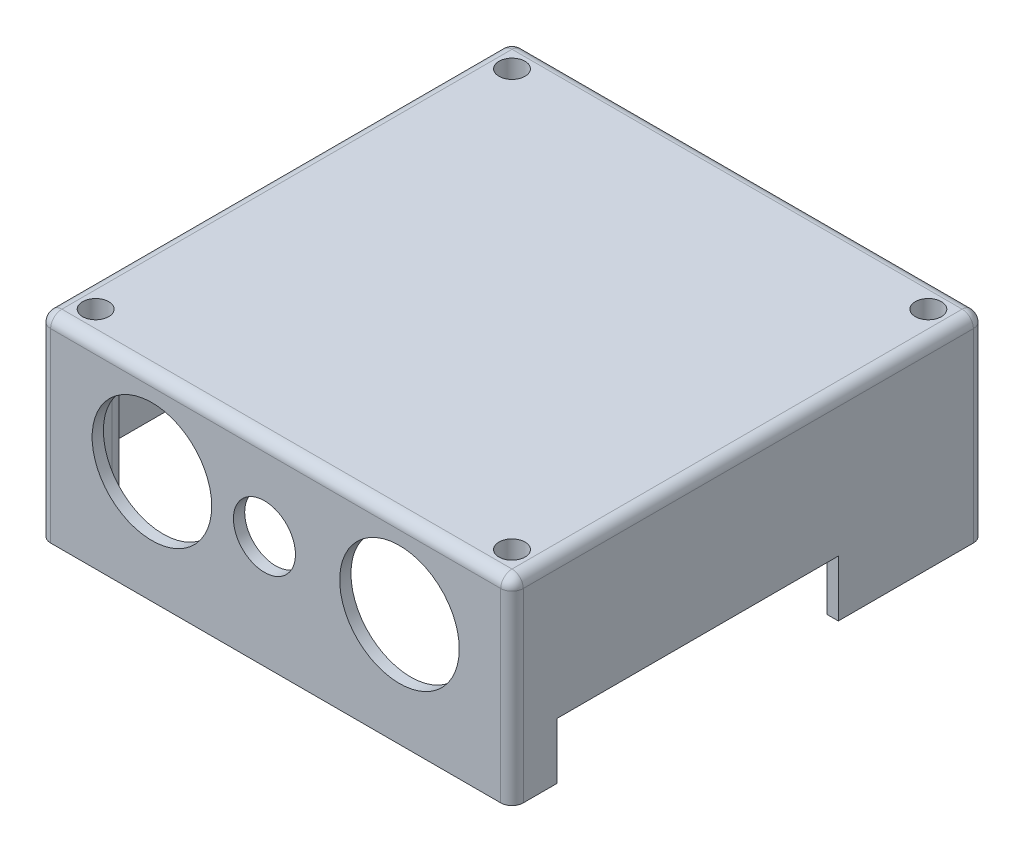
SolidWorks part; units mm, degrees
ref_plane "Front Plane" through (0, 0, 0) normal (0, 0, 1) x (1, 0, 0)
ref_plane "Top Plane" through (0, 0, 0) normal (0, 1, 0) x (1, 0, 0)
ref_plane "Right Plane" through (0, 0, 0) normal (1, 0, 0) x (0, 0, -1)
sketch "Sketch1" plane through (0, 0, 0) normal (0, 1, 0) x (1, 0, 0)
  line L0 (0, 0) -> (0, 50.8)
  line L1 (0, 50.8) -> (50.8, 50.8)
  line L2 (50.8, 50.8) -> (50.8, 0)
  line L3 (50.8, 0) -> (0, 0)
  line L4 (29.845, 40.64) -> (28.575, 40.64)
  line L5 (30.48, 43.18) -> (30.48, 38.1)
  line L6 (30.48, 38.1) -> (27.94, 38.1)
  line L7 (27.94, 38.1) -> (27.94, 43.18)
  line L8 (27.94, 43.18) -> (30.48, 43.18)
  line L9 (28.3382, 37.639) -> (28.245, 37.7322)
  line L10 (28.245, 37.7322) -> (28.0586, 37.7322)
  line L11 (28.0586, 37.7322) -> (27.9654, 37.639)
  line L12 (27.9654, 37.639) -> (27.9654, 37.2661)
  line L13 (27.9654, 37.2661) -> (28.0586, 37.1729)
  line L14 (28.0586, 37.1729) -> (28.245, 37.1729)
  line L15 (28.245, 37.1729) -> (28.3382, 37.2661)
  line L16 (28.5267, 37.5457) -> (28.7131, 37.7322)
  line L17 (28.7131, 37.7322) -> (28.7131, 37.1729)
  line L18 (28.5267, 37.1729) -> (28.8996, 37.1729)
  line L19 (28.2829, 43.8957) -> (28.4693, 44.0822)
  line L20 (28.4693, 44.0822) -> (28.4693, 43.5229)
  line L21 (28.2829, 43.5229) -> (28.6557, 43.5229)
  line L22 (28.8442, 43.6161) -> (28.8442, 43.989)
  line L23 (28.8442, 43.989) -> (28.9374, 44.0822)
  line L24 (28.9374, 44.0822) -> (29.1238, 44.0822)
  line L25 (29.1238, 44.0822) -> (29.2171, 43.989)
  line L26 (29.2171, 43.989) -> (29.2171, 43.6161)
  line L27 (29.2171, 43.6161) -> (29.1238, 43.5229)
  line L28 (29.1238, 43.5229) -> (28.9374, 43.5229)
  line L29 (28.9374, 43.5229) -> (28.8442, 43.6161)
  line L30 (28.8442, 43.6161) -> (29.2171, 43.989)
  line L31 (29.4055, 43.8957) -> (29.4055, 43.6161)
  line L32 (29.4055, 43.6161) -> (29.4987, 43.5229)
  line L33 (29.4987, 43.5229) -> (29.7784, 43.5229)
  line L34 (29.7784, 43.5229) -> (29.7784, 43.8957)
  line L35 (29.9668, 43.5229) -> (29.9668, 44.0822)
  line L36 (29.9668, 44.0822) -> (30.3397, 44.0822)
  line L37 (29.9668, 43.8025) -> (30.1533, 43.8025)
  line L38 (24.765, 40.64) -> (26.035, 40.64)
  line L39 (24.13, 38.1) -> (24.13, 43.18)
  line L40 (24.13, 43.18) -> (26.67, 43.18)
  line L41 (26.67, 43.18) -> (26.67, 38.1)
  line L42 (26.67, 38.1) -> (24.13, 38.1)
  line L43 (24.6756, 37.6644) -> (24.5824, 37.7576)
  line L44 (24.5824, 37.7576) -> (24.396, 37.7576)
  line L45 (24.396, 37.7576) -> (24.3028, 37.6644)
  line L46 (24.3028, 37.6644) -> (24.3028, 37.2915)
  line L47 (24.3028, 37.2915) -> (24.396, 37.1983)
  line L48 (24.396, 37.1983) -> (24.5824, 37.1983)
  line L49 (24.5824, 37.1983) -> (24.6756, 37.2915)
  line L50 (25.2369, 37.1983) -> (24.8641, 37.1983)
  line L51 (24.8641, 37.1983) -> (25.2369, 37.5711)
  line L52 (25.2369, 37.5711) -> (25.2369, 37.6644)
  line L53 (25.2369, 37.6644) -> (25.1437, 37.7576)
  line L54 (25.1437, 37.7576) -> (24.9573, 37.7576)
  line L55 (24.9573, 37.7576) -> (24.8641, 37.6644)
  line L56 (24.1326, 43.9211) -> (24.3191, 44.1076)
  line L57 (24.3191, 44.1076) -> (24.3191, 43.5483)
  line L58 (24.1326, 43.5483) -> (24.5055, 43.5483)
  line L59 (24.694, 43.6415) -> (24.694, 44.0144)
  line L60 (24.694, 44.0144) -> (24.7872, 44.1076)
  line L61 (24.7872, 44.1076) -> (24.9736, 44.1076)
  line L62 (24.9736, 44.1076) -> (25.0668, 44.0144)
  line L63 (25.0668, 44.0144) -> (25.0668, 43.6415)
  line L64 (25.0668, 43.6415) -> (24.9736, 43.5483)
  line L65 (24.9736, 43.5483) -> (24.7872, 43.5483)
  line L66 (24.7872, 43.5483) -> (24.694, 43.6415)
  line L67 (24.694, 43.6415) -> (25.0668, 44.0144)
  line L68 (25.2553, 43.9211) -> (25.2553, 43.6415)
  line L69 (25.2553, 43.6415) -> (25.3485, 43.5483)
  line L70 (25.3485, 43.5483) -> (25.6281, 43.5483)
  line L71 (25.6281, 43.5483) -> (25.6281, 43.9211)
  line L72 (25.8166, 43.5483) -> (25.8166, 44.1076)
  line L73 (25.8166, 44.1076) -> (26.1894, 44.1076)
  line L74 (25.8166, 43.8279) -> (26.003, 43.8279)
  line L75 (15.748, 34.29) -> (19.812, 34.29)
  line L76 (15.748, 34.29) -> (15.748, 31.75)
  line L77 (19.812, 31.75) -> (15.748, 31.75)
  line L78 (19.812, 31.75) -> (19.812, 34.29)
  line L79 (12.7, 33.02) -> (13.716, 33.02)
  line L80 (22.86, 33.02) -> (21.844, 33.02)
  line L81 (18.415, 33.02) -> (17.78, 33.02)
  line L82 (16.764, 32.385) -> (16.764, 33.655)
  line L83 (16.764, 33.655) -> (17.78, 33.02)
  line L84 (17.78, 33.02) -> (16.256, 33.02)
  line L85 (17.78, 33.02) -> (16.764, 32.385)
  line L86 (17.78, 32.385) -> (17.78, 33.02)
  line L87 (17.78, 33.02) -> (17.78, 33.655)
  line L88 (12.8591, 35.3702) -> (13.2404, 35.7515)
  line L89 (13.2404, 35.7515) -> (13.2404, 34.6075)
  line L90 (12.8591, 34.6075) -> (13.6217, 34.6075)
  line L91 (14.0285, 34.6075) -> (14.0285, 35.7515)
  line L92 (14.0285, 35.7515) -> (14.7912, 34.6075)
  line L93 (14.7912, 34.6075) -> (14.7912, 35.7515)
  line L94 (15.7699, 34.6075) -> (15.7699, 35.7515)
  line L95 (15.7699, 35.7515) -> (15.1979, 35.1795)
  line L96 (15.1979, 35.1795) -> (15.9605, 35.1795)
  line L97 (16.3673, 34.7982) -> (16.3673, 35.5608)
  line L98 (16.3673, 35.5608) -> (16.558, 35.7515)
  line L99 (16.558, 35.7515) -> (16.9393, 35.7515)
  line L100 (16.9393, 35.7515) -> (17.1299, 35.5608)
  line L101 (17.1299, 35.5608) -> (17.1299, 34.7982)
  line L102 (17.1299, 34.7982) -> (16.9393, 34.6075)
  line L103 (16.9393, 34.6075) -> (16.558, 34.6075)
  line L104 (16.558, 34.6075) -> (16.3673, 34.7982)
  line L105 (16.3673, 34.7982) -> (17.1299, 35.5608)
  line L106 (17.5367, 34.7982) -> (17.5367, 35.5608)
  line L107 (17.5367, 35.5608) -> (17.7273, 35.7515)
  line L108 (17.7273, 35.7515) -> (18.1087, 35.7515)
  line L109 (18.1087, 35.7515) -> (18.2993, 35.5608)
  line L110 (18.2993, 35.5608) -> (18.2993, 34.7982)
  line L111 (18.2993, 34.7982) -> (18.1087, 34.6075)
  line L112 (18.1087, 34.6075) -> (17.7273, 34.6075)
  line L113 (17.7273, 34.6075) -> (17.5367, 34.7982)
  line L114 (17.5367, 34.7982) -> (18.2993, 35.5608)
  line L115 (18.7061, 35.3702) -> (19.0874, 35.7515)
  line L116 (19.0874, 35.7515) -> (19.0874, 34.6075)
  line L117 (18.7061, 34.6075) -> (19.4687, 34.6075)
  line L118 (4.39, 39.64) -> (6.49, 39.64)
  line L119 (13.39, 50.34) -> (13.39, 53.24)
  line L120 (4.39, 53.24) -> (4.39, 50.34)
  line L121 (4.39, 53.24) -> (13.39, 53.24)
  line L122 (4.39, 50.34) -> (4.39, 45.04)
  line L123 (4.39, 39.64) -> (4.39, 40.34)
  line L124 (13.39, 50.34) -> (13.39, 39.64)
  line L125 (13.39, 39.64) -> (11.29, 39.64)
  line L126 (13.39, 50.34) -> (4.39, 50.34)
  line L127 (11.5901, 47.9299) -> (11.6536, 47.8663)
  line L128 (11.6536, 47.8663) -> (11.7172, 47.8663)
  line L129 (11.7172, 47.8663) -> (11.7807, 47.9299)
  line L130 (11.7807, 47.9299) -> (11.7807, 48.2476)
  line L131 (11.7172, 48.2476) -> (11.8443, 48.2476)
  line L132 (11.9643, 47.8663) -> (11.9643, 48.2476)
  line L133 (11.9643, 48.2476) -> (12.1549, 48.2476)
  line L134 (12.1549, 48.2476) -> (12.2185, 48.1841)
  line L135 (12.2185, 48.1841) -> (12.2185, 48.057)
  line L136 (12.2185, 48.057) -> (12.1549, 47.9934)
  line L137 (12.1549, 47.9934) -> (11.9643, 47.9934)
  line L138 (12.3385, 48.1205) -> (12.4656, 48.2476)
  line L139 (12.4656, 48.2476) -> (12.4656, 47.8663)
  line L140 (12.3385, 47.8663) -> (12.5927, 47.8663)
  line L141 (7.848, 49.1363) -> (7.848, 49.5176)
  line L142 (7.848, 49.5176) -> (8.0387, 49.5176)
  line L143 (8.0387, 49.5176) -> (8.1022, 49.4541)
  line L144 (8.1022, 49.4541) -> (8.1022, 49.327)
  line L145 (8.1022, 49.327) -> (8.0387, 49.2634)
  line L146 (8.0387, 49.2634) -> (7.848, 49.2634)
  line L147 (8.4129, 49.5176) -> (8.2858, 49.5176)
  line L148 (8.2858, 49.5176) -> (8.2222, 49.4541)
  line L149 (8.2222, 49.4541) -> (8.2222, 49.1999)
  line L150 (8.2222, 49.1999) -> (8.2858, 49.1363)
  line L151 (8.2858, 49.1363) -> (8.4129, 49.1363)
  line L152 (8.4129, 49.1363) -> (8.4764, 49.1999)
  line L153 (8.4764, 49.1999) -> (8.4764, 49.4541)
  line L154 (8.4764, 49.4541) -> (8.4129, 49.5176)
  line L155 (8.5964, 49.5176) -> (8.5964, 49.1363)
  line L156 (8.5964, 49.1363) -> (8.7235, 49.2634)
  line L157 (8.7235, 49.2634) -> (8.8506, 49.1363)
  line L158 (8.8506, 49.1363) -> (8.8506, 49.5176)
  line L159 (9.2248, 49.5176) -> (8.9706, 49.5176)
  line L160 (8.9706, 49.5176) -> (8.9706, 49.1363)
  line L161 (8.9706, 49.1363) -> (9.2248, 49.1363)
  line L162 (8.9706, 49.327) -> (9.0977, 49.327)
  line L163 (9.3448, 49.1363) -> (9.3448, 49.5176)
  line L164 (9.3448, 49.5176) -> (9.5355, 49.5176)
  line L165 (9.5355, 49.5176) -> (9.599, 49.4541)
  line L166 (9.599, 49.4541) -> (9.599, 49.327)
  line L167 (9.599, 49.327) -> (9.5355, 49.2634)
  line L168 (9.5355, 49.2634) -> (9.3448, 49.2634)
  line L169 (9.4719, 49.2634) -> (9.599, 49.1363)
  line L170 (9.719, 49.0727) -> (9.9733, 49.0727)
  line L171 (10.0932, 49.1999) -> (10.1568, 49.1363)
  line L172 (10.1568, 49.1363) -> (10.2204, 49.1363)
  line L173 (10.2204, 49.1363) -> (10.2839, 49.1999)
  line L174 (10.2839, 49.1999) -> (10.2839, 49.5176)
  line L175 (10.2204, 49.5176) -> (10.3475, 49.5176)
  line L176 (10.4674, 49.1363) -> (10.4674, 49.3905)
  line L177 (10.4674, 49.3905) -> (10.5945, 49.5176)
  line L178 (10.5945, 49.5176) -> (10.7217, 49.3905)
  line L179 (10.7217, 49.3905) -> (10.7217, 49.1363)
  line L180 (10.4674, 49.327) -> (10.7217, 49.327)
  line L181 (11.0959, 49.4541) -> (11.0323, 49.5176)
  line L182 (11.0323, 49.5176) -> (10.9052, 49.5176)
  line L183 (10.9052, 49.5176) -> (10.8417, 49.4541)
  line L184 (10.8417, 49.4541) -> (10.8417, 49.1999)
  line L185 (10.8417, 49.1999) -> (10.9052, 49.1363)
  line L186 (10.9052, 49.1363) -> (11.0323, 49.1363)
  line L187 (11.0323, 49.1363) -> (11.0959, 49.1999)
  line L188 (11.2159, 49.5176) -> (11.2159, 49.1363)
  line L189 (11.2159, 49.2634) -> (11.4701, 49.5176)
  line L190 (11.2794, 49.327) -> (11.4701, 49.1363)
  line L191 (11.5901, 49.1363) -> (11.5901, 49.5176)
  line L192 (11.5901, 49.5176) -> (11.7807, 49.5176)
  line L193 (11.7807, 49.5176) -> (11.8443, 49.4541)
  line L194 (11.8443, 49.4541) -> (11.8443, 49.327)
  line L195 (11.8443, 49.327) -> (11.7807, 49.2634)
  line L196 (11.7807, 49.2634) -> (11.5901, 49.2634)
  line L197 (12.0914, 49.1363) -> (12.0914, 49.5176)
  line L198 (11.9643, 49.5176) -> (12.2185, 49.5176)
  line L199 (12.3385, 49.1363) -> (12.3385, 49.5176)
  line L200 (12.3385, 49.327) -> (12.5927, 49.327)
  line L201 (12.5927, 49.5176) -> (12.5927, 49.1363)
  line L202 (10.795, 1.27) -> (24.765, 1.27)
  line L203 (24.765, 1.27) -> (24.765, 35.56)
  line L204 (24.765, 35.56) -> (10.795, 35.56)
  line L205 (10.795, 35.56) -> (10.795, 1.27)
  line L206 (14.1986, 3.8354) -> (13.6393, 3.8354)
  line L207 (13.6393, 3.8354) -> (13.6393, 4.115)
  line L208 (13.6393, 4.115) -> (13.7325, 4.2082)
  line L209 (13.7325, 4.2082) -> (13.919, 4.2082)
  line L210 (13.919, 4.2082) -> (14.0122, 4.115)
  line L211 (14.0122, 4.115) -> (14.0122, 3.8354)
  line L212 (14.0122, 4.0218) -> (14.1986, 4.2082)
  line L213 (13.6393, 4.3967) -> (14.1986, 4.7696)
  line L214 (13.6393, 4.7696) -> (14.1986, 4.3967)
  line L215 (16.7386, 4.0218) -> (16.1793, 4.0218)
  line L216 (16.1793, 3.8354) -> (16.1793, 4.2082)
  line L217 (16.1793, 4.3967) -> (16.7386, 4.7696)
  line L218 (16.1793, 4.7696) -> (16.7386, 4.3967)
  line L219 (18.8125, 4.2082) -> (18.7193, 4.115)
  line L220 (18.7193, 4.115) -> (18.7193, 3.9286)
  line L221 (18.7193, 3.9286) -> (18.8125, 3.8354)
  line L222 (18.8125, 3.8354) -> (19.1854, 3.8354)
  line L223 (19.1854, 3.8354) -> (19.2786, 3.9286)
  line L224 (19.2786, 3.9286) -> (19.2786, 4.115)
  line L225 (19.2786, 4.115) -> (19.1854, 4.2082)
  line L226 (19.1854, 4.2082) -> (18.999, 4.2082)
  line L227 (18.999, 4.2082) -> (18.999, 4.0218)
  line L228 (19.2786, 4.3967) -> (18.7193, 4.3967)
  line L229 (18.7193, 4.3967) -> (19.2786, 4.7696)
  line L230 (19.2786, 4.7696) -> (18.7193, 4.7696)
  line L231 (18.7193, 4.958) -> (19.2786, 4.958)
  line L232 (19.2786, 4.958) -> (19.2786, 5.2377)
  line L233 (19.2786, 5.2377) -> (19.1854, 5.3309)
  line L234 (19.1854, 5.3309) -> (18.8125, 5.3309)
  line L235 (18.8125, 5.3309) -> (18.7193, 5.2377)
  line L236 (18.7193, 5.2377) -> (18.7193, 4.958)
  line L237 (21.2593, 3.8354) -> (21.6322, 3.8354)
  line L238 (21.6322, 3.8354) -> (21.8186, 4.0218)
  line L239 (21.8186, 4.0218) -> (21.6322, 4.2082)
  line L240 (21.6322, 4.2082) -> (21.2593, 4.2082)
  line L241 (21.3525, 4.7696) -> (21.2593, 4.6763)
  line L242 (21.2593, 4.6763) -> (21.2593, 4.4899)
  line L243 (21.2593, 4.4899) -> (21.3525, 4.3967)
  line L244 (21.3525, 4.3967) -> (21.7254, 4.3967)
  line L245 (21.7254, 4.3967) -> (21.8186, 4.4899)
  line L246 (21.8186, 4.4899) -> (21.8186, 4.6763)
  line L247 (21.8186, 4.6763) -> (21.7254, 4.7696)
  line L248 (21.3525, 5.3309) -> (21.2593, 5.2377)
  line L249 (21.2593, 5.2377) -> (21.2593, 5.0512)
  line L250 (21.2593, 5.0512) -> (21.3525, 4.958)
  line L251 (21.3525, 4.958) -> (21.7254, 4.958)
  line L252 (21.7254, 4.958) -> (21.8186, 5.0512)
  line L253 (21.8186, 5.0512) -> (21.8186, 5.2377)
  line L254 (21.8186, 5.2377) -> (21.7254, 5.3309)
  line L255 (10.0752, 1.3335) -> (10.2235, 1.4818)
  line L256 (10.2235, 1.4818) -> (10.2235, 1.6301)
  line L257 (10.2235, 1.6301) -> (10.0752, 1.7784)
  line L258 (10.0752, 1.7784) -> (9.3337, 1.7784)
  line L259 (9.3337, 1.6301) -> (9.3337, 1.9267)
  line L260 (10.3718, 2.269) -> (10.3718, 2.8622)
  line L261 (10.2235, 3.2045) -> (9.3337, 3.2045)
  line L262 (9.3337, 3.2045) -> (9.3337, 3.6494)
  line L263 (9.3337, 3.6494) -> (9.482, 3.7977)
  line L264 (9.482, 3.7977) -> (9.6303, 3.7977)
  line L265 (9.6303, 3.7977) -> (9.7786, 3.6494)
  line L266 (9.7786, 3.6494) -> (9.9269, 3.7977)
  line L267 (9.9269, 3.7977) -> (10.0752, 3.7977)
  line L268 (10.0752, 3.7977) -> (10.2235, 3.6494)
  line L269 (10.2235, 3.6494) -> (10.2235, 3.2045)
  line L270 (9.7786, 3.2045) -> (9.7786, 3.6494)
  line L271 (10.2235, 4.4366) -> (9.3337, 4.4366)
  line L272 (9.3337, 4.14) -> (9.3337, 4.7332)
  line L273 (10.3718, 5.0756) -> (10.3718, 5.6687)
  line L274 (10.2235, 6.0111) -> (9.3337, 6.0111)
  line L275 (9.3337, 6.0111) -> (9.3337, 6.456)
  line L276 (9.3337, 6.456) -> (9.482, 6.6043)
  line L277 (9.482, 6.6043) -> (9.6303, 6.6043)
  line L278 (9.6303, 6.6043) -> (9.7786, 6.456)
  line L279 (9.7786, 6.456) -> (9.9269, 6.6043)
  line L280 (9.9269, 6.6043) -> (10.0752, 6.6043)
  line L281 (10.0752, 6.6043) -> (10.2235, 6.456)
  line L282 (10.2235, 6.456) -> (10.2235, 6.0111)
  line L283 (9.7786, 6.0111) -> (9.7786, 6.456)
  line L284 (9.3337, 7.3915) -> (9.3337, 7.0949)
  line L285 (9.3337, 7.0949) -> (9.482, 6.9466)
  line L286 (9.482, 6.9466) -> (10.0752, 6.9466)
  line L287 (10.0752, 6.9466) -> (10.2235, 7.0949)
  line L288 (10.2235, 7.0949) -> (10.2235, 7.3915)
  line L289 (10.2235, 7.3915) -> (10.0752, 7.5398)
  line L290 (10.0752, 7.5398) -> (9.482, 7.5398)
  line L291 (9.482, 7.5398) -> (9.3337, 7.3915)
  line L292 (10.2235, 7.8821) -> (9.6303, 7.8821)
  line L293 (9.6303, 7.8821) -> (9.3337, 8.1787)
  line L294 (9.3337, 8.1787) -> (9.6303, 8.4753)
  line L295 (9.6303, 8.4753) -> (10.2235, 8.4753)
  line L296 (9.7786, 7.8821) -> (9.7786, 8.4753)
  line L297 (10.2235, 8.8177) -> (9.3337, 8.8177)
  line L298 (9.3337, 8.8177) -> (9.3337, 9.2625)
  line L299 (9.3337, 9.2625) -> (9.482, 9.4108)
  line L300 (9.482, 9.4108) -> (9.7786, 9.4108)
  line L301 (9.7786, 9.4108) -> (9.9269, 9.2625)
  line L302 (9.9269, 9.2625) -> (9.9269, 8.8177)
  line L303 (9.9269, 9.1142) -> (10.2235, 9.4108)
  line L304 (9.3337, 9.7532) -> (10.2235, 9.7532)
  line L305 (10.2235, 9.7532) -> (10.2235, 10.198)
  line L306 (10.2235, 10.198) -> (10.0752, 10.3463)
  line L307 (10.0752, 10.3463) -> (9.482, 10.3463)
  line L308 (9.482, 10.3463) -> (9.3337, 10.198)
  line L309 (9.3337, 10.198) -> (9.3337, 9.7532)
  line L310 (10.3718, 10.6887) -> (10.3718, 11.2819)
  line L311 (9.6303, 11.6242) -> (9.3337, 11.9208)
  line L312 (9.3337, 11.9208) -> (10.2235, 11.9208)
  line L313 (10.2235, 11.6242) -> (10.2235, 12.2174)
  line L314 (3.81, 35.8648) -> (1.27, 35.8648)
  line L315 (0.9515, 36.2585) -> (2.0955, 36.2585)
  line L316 (2.0955, 36.2585) -> (2.0955, 37.0212)
  line L317 (0.9515, 38.1906) -> (0.9515, 37.4279)
  line L318 (0.9515, 37.4279) -> (2.0955, 37.4279)
  line L319 (2.0955, 37.4279) -> (2.0955, 38.1906)
  line L320 (1.5235, 37.4279) -> (1.5235, 37.8092)
  line L321 (0.9515, 38.5973) -> (2.0955, 38.5973)
  line L322 (2.0955, 38.5973) -> (2.0955, 39.1693)
  line L323 (2.0955, 39.1693) -> (1.9048, 39.3599)
  line L324 (1.9048, 39.3599) -> (1.1422, 39.3599)
  line L325 (1.1422, 39.3599) -> (0.9515, 39.1693)
  line L326 (0.9515, 39.1693) -> (0.9515, 38.5973)
  line L327 (1.3328, 39.7667) -> (0.9515, 40.148)
  line L328 (0.9515, 40.148) -> (2.0955, 40.148)
  line L329 (2.0955, 39.7667) -> (2.0955, 40.5293)
  line L330 (2.6768, 32.6898) -> (2.4032, 32.6898)
  line L331 (2.4032, 32.6898) -> (2.2098, 32.8832)
  line L332 (2.2098, 32.8832) -> (2.2098, 33.1568)
  line L333 (2.2098, 33.1568) -> (2.4032, 33.3502)
  line L334 (2.4032, 33.3502) -> (2.6768, 33.3502)
  line L335 (2.6768, 33.3502) -> (2.8702, 33.1568)
  line L336 (2.8702, 33.1568) -> (2.8702, 32.8832)
  line L337 (2.8702, 32.8832) -> (2.6768, 32.6898)
  line L338 (2.6768, 32.6898) -> (2.4032, 32.6898)
  line L339 (2.6768, 32.6898) -> (2.4032, 32.6898)
  line L340 (2.4032, 32.6898) -> (2.2098, 32.8832)
  line L341 (2.2098, 32.8832) -> (2.2098, 33.1568)
  line L342 (2.2098, 33.1568) -> (2.4032, 33.3502)
  line L343 (2.4032, 33.3502) -> (2.6768, 33.3502)
  line L344 (2.6768, 33.3502) -> (2.8702, 33.1568)
  line L345 (2.8702, 33.1568) -> (2.8702, 32.8832)
  line L346 (2.8702, 32.8832) -> (2.6768, 32.6898)
  line L347 (2.6768, 32.6898) -> (2.4032, 32.6898)
  line L348 (2.6768, 35.2298) -> (2.4032, 35.2298)
  line L349 (2.4032, 35.2298) -> (2.2098, 35.4232)
  line L350 (2.2098, 35.4232) -> (2.2098, 35.6968)
  line L351 (2.2098, 35.6968) -> (2.4032, 35.8902)
  line L352 (2.4032, 35.8902) -> (2.6768, 35.8902)
  line L353 (2.6768, 35.8902) -> (2.8702, 35.6968)
  line L354 (2.8702, 35.6968) -> (2.8702, 35.4232)
  line L355 (2.8702, 35.4232) -> (2.6768, 35.2298)
  line L356 (2.6768, 35.2298) -> (2.4032, 35.2298)
  line L357 (2.6768, 35.2298) -> (2.4032, 35.2298)
  line L358 (2.4032, 35.2298) -> (2.2098, 35.4232)
  line L359 (2.2098, 35.4232) -> (2.2098, 35.6968)
  line L360 (2.2098, 35.6968) -> (2.4032, 35.8902)
  line L361 (2.4032, 35.8902) -> (2.6768, 35.8902)
  line L362 (2.6768, 35.8902) -> (2.8702, 35.6968)
  line L363 (2.8702, 35.6968) -> (2.8702, 35.4232)
  line L364 (2.8702, 35.4232) -> (2.6768, 35.2298)
  line L365 (2.6768, 35.2298) -> (2.4032, 35.2298)
  line L366 (10.16, 36.83) -> (10.16, 31.75)
  line L367 (10.16, 31.75) -> (5.08, 31.75)
  line L368 (5.08, 31.75) -> (5.08, 36.83)
  line L369 (5.08, 36.83) -> (10.16, 36.83)
  line L370 (8.9275, 32.8596) -> (8.9275, 32.6139)
  line L371 (8.9275, 32.6139) -> (9.0504, 32.491)
  line L372 (9.0504, 32.491) -> (9.5418, 32.491)
  line L373 (9.5418, 32.491) -> (9.6647, 32.6139)
  line L374 (9.6647, 32.6139) -> (9.6647, 32.8596)
  line L375 (9.6647, 32.8596) -> (9.5418, 32.9825)
  line L376 (9.5418, 32.9825) -> (9.0504, 32.9825)
  line L377 (9.0504, 32.9825) -> (8.9275, 32.8596)
  line L378 (9.6647, 33.2394) -> (8.9275, 33.2394)
  line L379 (8.9275, 33.2394) -> (9.6647, 33.7309)
  line L380 (9.6647, 33.7309) -> (8.9275, 33.7309)
  line L381 (8.9275, 34.3565) -> (8.9275, 34.1107)
  line L382 (8.9275, 34.1107) -> (9.0504, 33.9878)
  line L383 (9.0504, 33.9878) -> (9.5418, 33.9878)
  line L384 (9.5418, 33.9878) -> (9.6647, 34.1107)
  line L385 (9.6647, 34.1107) -> (9.6647, 34.3565)
  line L386 (9.6647, 34.3565) -> (9.5418, 34.4793)
  line L387 (9.5418, 34.4793) -> (9.0504, 34.4793)
  line L388 (9.0504, 34.4793) -> (8.9275, 34.3565)
  line L389 (9.6647, 34.7363) -> (8.9275, 34.7363)
  line L390 (8.9275, 34.7363) -> (8.9275, 35.2277)
  line L391 (9.2961, 34.7363) -> (9.2961, 34.982)
  line L392 (9.6647, 35.4847) -> (8.9275, 35.4847)
  line L393 (8.9275, 35.4847) -> (8.9275, 35.9762)
  line L394 (9.2961, 35.4847) -> (9.2961, 35.7304)
  line L395 (5.7525, 31.7426) -> (6.4897, 31.7426)
  line L396 (6.4897, 31.7426) -> (6.4897, 32.1112)
  line L397 (6.4897, 32.1112) -> (6.3668, 32.2341)
  line L398 (6.3668, 32.2341) -> (5.8754, 32.2341)
  line L399 (5.8754, 32.2341) -> (5.7525, 32.1112)
  line L400 (5.7525, 32.1112) -> (5.7525, 31.7426)
  line L401 (5.8754, 32.9825) -> (5.7525, 32.8596)
  line L402 (5.7525, 32.8596) -> (5.7525, 32.6139)
  line L403 (5.7525, 32.6139) -> (5.8754, 32.491)
  line L404 (5.8754, 32.491) -> (5.9982, 32.491)
  line L405 (5.9982, 32.491) -> (6.1211, 32.6139)
  line L406 (6.1211, 32.6139) -> (6.1211, 32.8596)
  line L407 (6.1211, 32.8596) -> (6.244, 32.9825)
  line L408 (6.244, 32.9825) -> (6.3668, 32.9825)
  line L409 (6.3668, 32.9825) -> (6.4897, 32.8596)
  line L410 (6.4897, 32.8596) -> (6.4897, 32.6139)
  line L411 (6.4897, 32.6139) -> (6.3668, 32.491)
  line L412 (6.1211, 33.2394) -> (6.1211, 33.7309)
  line L413 (6.4897, 34.4793) -> (6.4897, 33.9878)
  line L414 (6.4897, 33.9878) -> (5.9982, 34.4793)
  line L415 (5.9982, 34.4793) -> (5.8754, 34.4793)
  line L416 (5.8754, 34.4793) -> (5.7525, 34.3565)
  line L417 (5.7525, 34.3565) -> (5.7525, 34.1107)
  line L418 (5.7525, 34.1107) -> (5.8754, 33.9878)
  line L419 (6.4897, 35.2277) -> (6.4897, 34.7363)
  line L420 (6.4897, 34.7363) -> (5.9982, 35.2277)
  line L421 (5.9982, 35.2277) -> (5.8754, 35.2277)
  line L422 (5.8754, 35.2277) -> (5.7525, 35.1049)
  line L423 (5.7525, 35.1049) -> (5.7525, 34.8591)
  line L424 (5.7525, 34.8591) -> (5.8754, 34.7363)
  line L425 (5.8754, 35.4847) -> (5.7525, 35.6075)
  line L426 (5.7525, 35.6075) -> (5.7525, 35.8533)
  line L427 (5.7525, 35.8533) -> (5.8754, 35.9762)
  line L428 (5.8754, 35.9762) -> (5.9982, 35.9762)
  line L429 (5.9982, 35.9762) -> (6.1211, 35.8533)
  line L430 (6.1211, 35.8533) -> (6.244, 35.9762)
  line L431 (6.244, 35.9762) -> (6.3668, 35.9762)
  line L432 (6.3668, 35.9762) -> (6.4897, 35.8533)
  line L433 (6.4897, 35.8533) -> (6.4897, 35.6075)
  line L434 (6.4897, 35.6075) -> (6.3668, 35.4847)
  line L435 (6.3668, 35.4847) -> (6.244, 35.4847)
  line L436 (6.244, 35.4847) -> (6.1211, 35.6075)
  line L437 (6.1211, 35.6075) -> (5.9982, 35.4847)
  line L438 (5.9982, 35.4847) -> (5.8754, 35.4847)
  line L439 (6.1211, 35.6075) -> (6.1211, 35.8533)
  line L440 (15.24, 21.082) -> (20.32, 21.082)
  line L441 (20.32, 21.082) -> (20.32, 20.32)
  line L442 (20.32, 20.32) -> (20.32, 19.558)
  line L443 (20.32, 19.558) -> (15.24, 19.558)
  line L444 (15.24, 19.558) -> (15.24, 20.32)
  line L445 (15.24, 20.32) -> (15.24, 21.082)
  line L446 (20.32, 20.32) -> (20.574, 20.32)
  line L447 (15.24, 20.32) -> (14.986, 20.32)
  line L448 (15.2527, 21.6027) -> (15.2527, 21.984)
  line L449 (15.2527, 21.984) -> (15.4434, 21.984)
  line L450 (15.4434, 21.984) -> (15.5069, 21.9205)
  line L451 (15.5069, 21.9205) -> (15.5069, 21.7934)
  line L452 (15.5069, 21.7934) -> (15.4434, 21.7298)
  line L453 (15.4434, 21.7298) -> (15.2527, 21.7298)
  line L454 (15.3798, 21.7298) -> (15.5069, 21.6027)
  line L455 (15.6269, 21.8569) -> (15.754, 21.984)
  line L456 (15.754, 21.984) -> (15.754, 21.6027)
  line L457 (15.6269, 21.6027) -> (15.8811, 21.6027)
  line L458 (15.8242, 20.5914) -> (16.1123, 20.8795)
  line L459 (16.1123, 20.8795) -> (16.1123, 20.0152)
  line L460 (15.8242, 20.0152) -> (16.4004, 20.0152)
  line L461 (16.7597, 20.1593) -> (16.7597, 20.7355)
  line L462 (16.7597, 20.7355) -> (16.9038, 20.8795)
  line L463 (16.9038, 20.8795) -> (17.1919, 20.8795)
  line L464 (17.1919, 20.8795) -> (17.3359, 20.7355)
  line L465 (17.3359, 20.7355) -> (17.3359, 20.1593)
  line L466 (17.3359, 20.1593) -> (17.1919, 20.0152)
  line L467 (17.1919, 20.0152) -> (16.9038, 20.0152)
  line L468 (16.9038, 20.0152) -> (16.7597, 20.1593)
  line L469 (16.7597, 20.1593) -> (17.3359, 20.7355)
  line L470 (17.6952, 20.8795) -> (17.6952, 20.0152)
  line L471 (17.6952, 20.3033) -> (18.2715, 20.8795)
  line L472 (17.8393, 20.4474) -> (18.2715, 20.0152)
  line L473 (15.24, 18.542) -> (20.32, 18.542)
  line L474 (20.32, 18.542) -> (20.32, 17.78)
  line L475 (20.32, 17.78) -> (20.32, 17.018)
  line L476 (20.32, 17.018) -> (15.24, 17.018)
  line L477 (15.24, 17.018) -> (15.24, 17.78)
  line L478 (15.24, 17.78) -> (15.24, 18.542)
  line L479 (20.32, 17.78) -> (20.574, 17.78)
  line L480 (15.24, 17.78) -> (14.986, 17.78)
  line L481 (15.2527, 19.0627) -> (15.2527, 19.444)
  line L482 (15.2527, 19.444) -> (15.4434, 19.444)
  line L483 (15.4434, 19.444) -> (15.5069, 19.3805)
  line L484 (15.5069, 19.3805) -> (15.5069, 19.2534)
  line L485 (15.5069, 19.2534) -> (15.4434, 19.1898)
  line L486 (15.4434, 19.1898) -> (15.2527, 19.1898)
  line L487 (15.3798, 19.1898) -> (15.5069, 19.0627)
  line L488 (15.8811, 19.0627) -> (15.6269, 19.0627)
  line L489 (15.6269, 19.0627) -> (15.8811, 19.3169)
  line L490 (15.8811, 19.3169) -> (15.8811, 19.3805)
  line L491 (15.8811, 19.3805) -> (15.8176, 19.444)
  line L492 (15.8176, 19.444) -> (15.6905, 19.444)
  line L493 (15.6905, 19.444) -> (15.6269, 19.3805)
  line L494 (15.8242, 18.0514) -> (16.1123, 18.3395)
  line L495 (16.1123, 18.3395) -> (16.1123, 17.4752)
  line L496 (15.8242, 17.4752) -> (16.4004, 17.4752)
  line L497 (16.7597, 17.6193) -> (16.7597, 18.1955)
  line L498 (16.7597, 18.1955) -> (16.9038, 18.3395)
  line L499 (16.9038, 18.3395) -> (17.1919, 18.3395)
  line L500 (17.1919, 18.3395) -> (17.3359, 18.1955)
  line L501 (17.3359, 18.1955) -> (17.3359, 17.6193)
  line L502 (17.3359, 17.6193) -> (17.1919, 17.4752)
  line L503 (17.1919, 17.4752) -> (16.9038, 17.4752)
  line L504 (16.9038, 17.4752) -> (16.7597, 17.6193)
  line L505 (16.7597, 17.6193) -> (17.3359, 18.1955)
  line L506 (17.6952, 18.3395) -> (17.6952, 17.4752)
  line L507 (17.6952, 17.7633) -> (18.2715, 18.3395)
  line L508 (17.8393, 17.9074) -> (18.2715, 17.4752)
  line L509 (15.24, 16.002) -> (20.32, 16.002)
  line L510 (20.32, 16.002) -> (20.32, 15.24)
  line L511 (20.32, 15.24) -> (20.32, 14.478)
  line L512 (20.32, 14.478) -> (15.24, 14.478)
  line L513 (15.24, 14.478) -> (15.24, 15.24)
  line L514 (15.24, 15.24) -> (15.24, 16.002)
  line L515 (20.32, 15.24) -> (20.574, 15.24)
  line L516 (15.24, 15.24) -> (14.986, 15.24)
  line L517 (15.2527, 16.5227) -> (15.2527, 16.904)
  line L518 (15.2527, 16.904) -> (15.4434, 16.904)
  line L519 (15.4434, 16.904) -> (15.5069, 16.8405)
  line L520 (15.5069, 16.8405) -> (15.5069, 16.7134)
  line L521 (15.5069, 16.7134) -> (15.4434, 16.6498)
  line L522 (15.4434, 16.6498) -> (15.2527, 16.6498)
  line L523 (15.3798, 16.6498) -> (15.5069, 16.5227)
  line L524 (15.6269, 16.8405) -> (15.6905, 16.904)
  line L525 (15.6905, 16.904) -> (15.8176, 16.904)
  line L526 (15.8176, 16.904) -> (15.8811, 16.8405)
  line L527 (15.8811, 16.8405) -> (15.8811, 16.7769)
  line L528 (15.8811, 16.7769) -> (15.8176, 16.7134)
  line L529 (15.8176, 16.7134) -> (15.754, 16.7134)
  line L530 (15.8176, 16.7134) -> (15.8811, 16.6498)
  line L531 (15.8811, 16.6498) -> (15.8811, 16.5863)
  line L532 (15.8811, 16.5863) -> (15.8176, 16.5227)
  line L533 (15.8176, 16.5227) -> (15.6905, 16.5227)
  line L534 (15.6905, 16.5227) -> (15.6269, 16.5863)
  line L535 (15.8242, 15.5114) -> (16.1123, 15.7995)
  line L536 (16.1123, 15.7995) -> (16.1123, 14.9352)
  line L537 (15.8242, 14.9352) -> (16.4004, 14.9352)
  line L538 (16.7597, 15.0793) -> (16.7597, 15.6555)
  line L539 (16.7597, 15.6555) -> (16.9038, 15.7995)
  line L540 (16.9038, 15.7995) -> (17.1919, 15.7995)
  line L541 (17.1919, 15.7995) -> (17.3359, 15.6555)
  line L542 (17.3359, 15.6555) -> (17.3359, 15.0793)
  line L543 (17.3359, 15.0793) -> (17.1919, 14.9352)
  line L544 (17.1919, 14.9352) -> (16.9038, 14.9352)
  line L545 (16.9038, 14.9352) -> (16.7597, 15.0793)
  line L546 (16.7597, 15.0793) -> (17.3359, 15.6555)
  line L547 (17.6952, 15.7995) -> (17.6952, 14.9352)
  line L548 (17.6952, 15.2233) -> (18.2715, 15.7995)
  line L549 (17.8393, 15.3674) -> (18.2715, 14.9352)
  line L550 (15.24, 13.462) -> (20.32, 13.462)
  line L551 (20.32, 13.462) -> (20.32, 12.7)
  line L552 (20.32, 12.7) -> (20.32, 11.938)
  line L553 (20.32, 11.938) -> (15.24, 11.938)
  line L554 (15.24, 11.938) -> (15.24, 12.7)
  line L555 (15.24, 12.7) -> (15.24, 13.462)
  line L556 (20.32, 12.7) -> (20.574, 12.7)
  line L557 (15.24, 12.7) -> (14.986, 12.7)
  line L558 (15.2527, 13.9827) -> (15.2527, 14.364)
  line L559 (15.2527, 14.364) -> (15.4434, 14.364)
  line L560 (15.4434, 14.364) -> (15.5069, 14.3005)
  line L561 (15.5069, 14.3005) -> (15.5069, 14.1734)
  line L562 (15.5069, 14.1734) -> (15.4434, 14.1098)
  line L563 (15.4434, 14.1098) -> (15.2527, 14.1098)
  line L564 (15.3798, 14.1098) -> (15.5069, 13.9827)
  line L565 (15.8176, 13.9827) -> (15.8176, 14.364)
  line L566 (15.8176, 14.364) -> (15.6269, 14.1734)
  line L567 (15.6269, 14.1734) -> (15.8811, 14.1734)
  line L568 (15.8242, 12.9714) -> (16.1123, 13.2595)
  line L569 (16.1123, 13.2595) -> (16.1123, 12.3952)
  line L570 (15.8242, 12.3952) -> (16.4004, 12.3952)
  line L571 (16.7597, 12.5393) -> (16.7597, 13.1155)
  line L572 (16.7597, 13.1155) -> (16.9038, 13.2595)
  line L573 (16.9038, 13.2595) -> (17.1919, 13.2595)
  line L574 (17.1919, 13.2595) -> (17.3359, 13.1155)
  line L575 (17.3359, 13.1155) -> (17.3359, 12.5393)
  line L576 (17.3359, 12.5393) -> (17.1919, 12.3952)
  line L577 (17.1919, 12.3952) -> (16.9038, 12.3952)
  line L578 (16.9038, 12.3952) -> (16.7597, 12.5393)
  line L579 (16.7597, 12.5393) -> (17.3359, 13.1155)
  line L580 (17.6952, 13.2595) -> (17.6952, 12.3952)
  line L581 (17.6952, 12.6833) -> (18.2715, 13.2595)
  line L582 (17.8393, 12.8274) -> (18.2715, 12.3952)
  line L583 (15.24, 10.922) -> (20.32, 10.922)
  line L584 (20.32, 10.922) -> (20.32, 10.16)
  line L585 (20.32, 10.16) -> (20.32, 9.398)
  line L586 (20.32, 9.398) -> (15.24, 9.398)
  line L587 (15.24, 9.398) -> (15.24, 10.16)
  line L588 (15.24, 10.16) -> (15.24, 10.922)
  line L589 (20.32, 10.16) -> (20.574, 10.16)
  line L590 (15.24, 10.16) -> (14.986, 10.16)
  line L591 (15.2527, 11.4427) -> (15.2527, 11.824)
  line L592 (15.2527, 11.824) -> (15.4434, 11.824)
  line L593 (15.4434, 11.824) -> (15.5069, 11.7605)
  line L594 (15.5069, 11.7605) -> (15.5069, 11.6334)
  line L595 (15.5069, 11.6334) -> (15.4434, 11.5698)
  line L596 (15.4434, 11.5698) -> (15.2527, 11.5698)
  line L597 (15.3798, 11.5698) -> (15.5069, 11.4427)
  line L598 (15.8811, 11.824) -> (15.6269, 11.824)
  line L599 (15.6269, 11.824) -> (15.6269, 11.6334)
  line L600 (15.6269, 11.6334) -> (15.754, 11.6969)
  line L601 (15.754, 11.6969) -> (15.8176, 11.6969)
  line L602 (15.8176, 11.6969) -> (15.8811, 11.6334)
  line L603 (15.8811, 11.6334) -> (15.8811, 11.5063)
  line L604 (15.8811, 11.5063) -> (15.8176, 11.4427)
  line L605 (15.8176, 11.4427) -> (15.6905, 11.4427)
  line L606 (15.6905, 11.4427) -> (15.6269, 11.5063)
  line L607 (15.8242, 10.4314) -> (16.1123, 10.7195)
  line L608 (16.1123, 10.7195) -> (16.1123, 9.8552)
  line L609 (15.8242, 9.8552) -> (16.4004, 9.8552)
  line L610 (16.7597, 9.9993) -> (16.7597, 10.5755)
  line L611 (16.7597, 10.5755) -> (16.9038, 10.7195)
  line L612 (16.9038, 10.7195) -> (17.1919, 10.7195)
  line L613 (17.1919, 10.7195) -> (17.3359, 10.5755)
  line L614 (17.3359, 10.5755) -> (17.3359, 9.9993)
  line L615 (17.3359, 9.9993) -> (17.1919, 9.8552)
  line L616 (17.1919, 9.8552) -> (16.9038, 9.8552)
  line L617 (16.9038, 9.8552) -> (16.7597, 9.9993)
  line L618 (16.7597, 9.9993) -> (17.3359, 10.5755)
  line L619 (17.6952, 10.7195) -> (17.6952, 9.8552)
  line L620 (17.6952, 10.1433) -> (18.2715, 10.7195)
  line L621 (17.8393, 10.2874) -> (18.2715, 9.8552)
  line L622 (15.24, 8.382) -> (20.32, 8.382)
  line L623 (20.32, 8.382) -> (20.32, 7.62)
  line L624 (20.32, 7.62) -> (20.32, 6.858)
  line L625 (20.32, 6.858) -> (15.24, 6.858)
  line L626 (15.24, 6.858) -> (15.24, 7.62)
  line L627 (15.24, 7.62) -> (15.24, 8.382)
  line L628 (20.32, 7.62) -> (20.574, 7.62)
  line L629 (15.24, 7.62) -> (14.986, 7.62)
  line L630 (15.2527, 8.9027) -> (15.2527, 9.284)
  line L631 (15.2527, 9.284) -> (15.4434, 9.284)
  line L632 (15.4434, 9.284) -> (15.5069, 9.2205)
  line L633 (15.5069, 9.2205) -> (15.5069, 9.0934)
  line L634 (15.5069, 9.0934) -> (15.4434, 9.0298)
  line L635 (15.4434, 9.0298) -> (15.2527, 9.0298)
  line L636 (15.3798, 9.0298) -> (15.5069, 8.9027)
  line L637 (15.8811, 9.284) -> (15.754, 9.2205)
  line L638 (15.754, 9.2205) -> (15.6269, 9.0934)
  line L639 (15.6269, 9.0934) -> (15.6269, 8.9663)
  line L640 (15.6269, 8.9663) -> (15.6905, 8.9027)
  line L641 (15.6905, 8.9027) -> (15.8176, 8.9027)
  line L642 (15.8176, 8.9027) -> (15.8811, 8.9663)
  line L643 (15.8811, 8.9663) -> (15.8811, 9.0298)
  line L644 (15.8811, 9.0298) -> (15.8176, 9.0934)
  line L645 (15.8176, 9.0934) -> (15.6269, 9.0934)
  line L646 (15.8242, 7.8914) -> (16.1123, 8.1795)
  line L647 (16.1123, 8.1795) -> (16.1123, 7.3152)
  line L648 (15.8242, 7.3152) -> (16.4004, 7.3152)
  line L649 (16.7597, 7.4593) -> (16.7597, 8.0355)
  line L650 (16.7597, 8.0355) -> (16.9038, 8.1795)
  line L651 (16.9038, 8.1795) -> (17.1919, 8.1795)
  line L652 (17.1919, 8.1795) -> (17.3359, 8.0355)
  line L653 (17.3359, 8.0355) -> (17.3359, 7.4593)
  line L654 (17.3359, 7.4593) -> (17.1919, 7.3152)
  line L655 (17.1919, 7.3152) -> (16.9038, 7.3152)
  line L656 (16.9038, 7.3152) -> (16.7597, 7.4593)
  line L657 (16.7597, 7.4593) -> (17.3359, 8.0355)
  line L658 (17.6952, 8.1795) -> (17.6952, 7.3152)
  line L659 (17.6952, 7.6033) -> (18.2715, 8.1795)
  line L660 (17.8393, 7.7474) -> (18.2715, 7.3152)
  line L661 (15.24, 28.702) -> (20.32, 28.702)
  line L662 (20.32, 28.702) -> (20.32, 27.94)
  line L663 (20.32, 27.94) -> (20.32, 27.178)
  line L664 (20.32, 27.178) -> (15.24, 27.178)
  line L665 (15.24, 27.178) -> (15.24, 27.94)
  line L666 (15.24, 27.94) -> (15.24, 28.702)
  line L667 (20.32, 27.94) -> (20.574, 27.94)
  line L668 (15.24, 27.94) -> (14.986, 27.94)
  line L669 (15.2527, 29.2227) -> (15.2527, 29.604)
  line L670 (15.2527, 29.604) -> (15.4434, 29.604)
  line L671 (15.4434, 29.604) -> (15.5069, 29.5405)
  line L672 (15.5069, 29.5405) -> (15.5069, 29.4134)
  line L673 (15.5069, 29.4134) -> (15.4434, 29.3498)
  line L674 (15.4434, 29.3498) -> (15.2527, 29.3498)
  line L675 (15.3798, 29.3498) -> (15.5069, 29.2227)
  line L676 (15.6269, 29.604) -> (15.8811, 29.604)
  line L677 (15.8811, 29.604) -> (15.8811, 29.5405)
  line L678 (15.8811, 29.5405) -> (15.6269, 29.2863)
  line L679 (15.6269, 29.2863) -> (15.6269, 29.2227)
  line L680 (15.8242, 28.2114) -> (16.1123, 28.4995)
  line L681 (16.1123, 28.4995) -> (16.1123, 27.6352)
  line L682 (15.8242, 27.6352) -> (16.4004, 27.6352)
  line L683 (16.7597, 27.6352) -> (16.7597, 27.7793)
  line L684 (16.7597, 27.7793) -> (16.9038, 27.7793)
  line L685 (16.9038, 27.7793) -> (16.9038, 27.6352)
  line L686 (16.9038, 27.6352) -> (16.7597, 27.6352)
  line L687 (17.2275, 28.2114) -> (17.5156, 28.4995)
  line L688 (17.5156, 28.4995) -> (17.5156, 27.6352)
  line L689 (17.2275, 27.6352) -> (17.8037, 27.6352)
  line L690 (18.163, 28.4995) -> (18.163, 27.6352)
  line L691 (18.163, 27.9233) -> (18.7392, 28.4995)
  line L692 (18.307, 28.0674) -> (18.7392, 27.6352)
  line L693 (25.4, 49.53) -> (30.48, 49.53)
  line L694 (30.48, 49.53) -> (30.48, 44.45)
  line L695 (30.48, 44.45) -> (25.4, 44.45)
  line L696 (25.4, 44.45) -> (25.4, 49.53)
  line L697 (26.0731, 48.2981) -> (26.0731, 49.0353)
  line L698 (26.0731, 49.0353) -> (26.4417, 49.0353)
  line L699 (26.4417, 49.0353) -> (26.5646, 48.9124)
  line L700 (26.5646, 48.9124) -> (26.5646, 48.6667)
  line L701 (26.5646, 48.6667) -> (26.4417, 48.5438)
  line L702 (26.4417, 48.5438) -> (26.0731, 48.5438)
  line L703 (26.3188, 48.5438) -> (26.5646, 48.2981)
  line L704 (27.313, 49.0353) -> (26.8215, 49.0353)
  line L705 (26.8215, 49.0353) -> (26.8215, 48.2981)
  line L706 (26.8215, 48.2981) -> (27.313, 48.2981)
  line L707 (26.8215, 48.6667) -> (27.0673, 48.6667)
  line L708 (28.0614, 48.9124) -> (27.9386, 49.0353)
  line L709 (27.9386, 49.0353) -> (27.6928, 49.0353)
  line L710 (27.6928, 49.0353) -> (27.5699, 48.9124)
  line L711 (27.5699, 48.9124) -> (27.5699, 48.7896)
  line L712 (27.5699, 48.7896) -> (27.6928, 48.6667)
  line L713 (27.6928, 48.6667) -> (27.9386, 48.6667)
  line L714 (27.9386, 48.6667) -> (28.0614, 48.5438)
  line L715 (28.0614, 48.5438) -> (28.0614, 48.421)
  line L716 (28.0614, 48.421) -> (27.9386, 48.2981)
  line L717 (27.9386, 48.2981) -> (27.6928, 48.2981)
  line L718 (27.6928, 48.2981) -> (27.5699, 48.421)
  line L719 (28.8098, 49.0353) -> (28.3184, 49.0353)
  line L720 (28.3184, 49.0353) -> (28.3184, 48.2981)
  line L721 (28.3184, 48.2981) -> (28.8098, 48.2981)
  line L722 (28.3184, 48.6667) -> (28.5641, 48.6667)
  line L723 (29.3125, 48.2981) -> (29.3125, 49.0353)
  line L724 (29.0668, 49.0353) -> (29.5583, 49.0353)
  line L725 (26.0731, 45.8603) -> (26.0731, 45.1231)
  line L726 (26.0731, 45.1231) -> (26.4417, 45.1231)
  line L727 (26.4417, 45.1231) -> (26.5646, 45.246)
  line L728 (26.5646, 45.246) -> (26.5646, 45.7374)
  line L729 (26.5646, 45.7374) -> (26.4417, 45.8603)
  line L730 (26.4417, 45.8603) -> (26.0731, 45.8603)
  line L731 (27.313, 45.7374) -> (27.1901, 45.8603)
  line L732 (27.1901, 45.8603) -> (26.9444, 45.8603)
  line L733 (26.9444, 45.8603) -> (26.8215, 45.7374)
  line L734 (26.8215, 45.7374) -> (26.8215, 45.6146)
  line L735 (26.8215, 45.6146) -> (26.9444, 45.4917)
  line L736 (26.9444, 45.4917) -> (27.1901, 45.4917)
  line L737 (27.1901, 45.4917) -> (27.313, 45.3688)
  line L738 (27.313, 45.3688) -> (27.313, 45.246)
  line L739 (27.313, 45.246) -> (27.1901, 45.1231)
  line L740 (27.1901, 45.1231) -> (26.9444, 45.1231)
  line L741 (26.9444, 45.1231) -> (26.8215, 45.246)
  line L742 (27.5699, 45.4917) -> (28.0614, 45.4917)
  line L743 (28.8098, 45.1231) -> (28.3184, 45.1231)
  line L744 (28.3184, 45.1231) -> (28.8098, 45.6146)
  line L745 (28.8098, 45.6146) -> (28.8098, 45.7374)
  line L746 (28.8098, 45.7374) -> (28.687, 45.8603)
  line L747 (28.687, 45.8603) -> (28.4412, 45.8603)
  line L748 (28.4412, 45.8603) -> (28.3184, 45.7374)
  line L749 (29.5583, 45.1231) -> (29.0668, 45.1231)
  line L750 (29.0668, 45.1231) -> (29.5583, 45.6146)
  line L751 (29.5583, 45.6146) -> (29.5583, 45.7374)
  line L752 (29.5583, 45.7374) -> (29.4354, 45.8603)
  line L753 (29.4354, 45.8603) -> (29.1896, 45.8603)
  line L754 (29.1896, 45.8603) -> (29.0668, 45.7374)
  line L755 (29.8152, 45.8603) -> (30.3067, 45.8603)
  line L756 (30.3067, 45.8603) -> (30.3067, 45.7374)
  line L757 (30.3067, 45.7374) -> (29.8152, 45.246)
  line L758 (29.8152, 45.246) -> (29.8152, 45.1231)
  line L759 (6.35, 20.32) -> (6.35, 30.48)
  line L760 (6.35, 30.48) -> (-5.08, 30.48)
  line L761 (-5.08, 30.48) -> (-5.08, 20.32)
  line L762 (-5.08, 20.32) -> (6.35, 20.32)
  line L763 (6.35, 20.32) -> (6.35, 30.48)
  line L764 (6.223, 20.32) -> (6.223, 30.48)
  line L765 (6.096, 20.32) -> (6.096, 30.48)
  line L766 (5.969, 20.32) -> (5.969, 30.48)
  line L767 (5.842, 20.32) -> (5.842, 30.48)
  line L768 (5.715, 20.32) -> (5.715, 30.48)
  line L769 (5.588, 20.32) -> (5.588, 30.48)
  line L770 (5.461, 20.32) -> (5.461, 30.48)
  line L771 (5.334, 20.32) -> (5.334, 30.48)
  line L772 (5.207, 20.32) -> (5.207, 30.48)
  line L773 (5.08, 20.32) -> (5.08, 30.48)
  line L774 (4.953, 20.32) -> (4.953, 30.48)
  line L775 (4.826, 20.32) -> (4.826, 30.48)
  line L776 (4.699, 20.32) -> (4.699, 30.48)
  line L777 (4.572, 20.32) -> (4.572, 30.48)
  line L778 (4.445, 20.32) -> (4.445, 30.48)
  line L779 (4.318, 20.32) -> (4.318, 30.48)
  line L780 (4.191, 20.32) -> (4.191, 30.48)
  line L781 (4.064, 20.32) -> (4.064, 30.48)
  line L782 (3.937, 20.32) -> (3.937, 30.48)
  line L783 (3.81, 20.32) -> (3.81, 30.48)
  line L784 (3.683, 20.32) -> (3.683, 30.48)
  line L785 (3.556, 20.32) -> (3.556, 30.48)
  line L786 (3.429, 20.32) -> (3.429, 30.48)
  line L787 (3.302, 20.32) -> (3.302, 30.48)
  line L788 (3.175, 20.32) -> (3.175, 30.48)
  line L789 (3.048, 20.32) -> (3.048, 30.48)
  line L790 (2.921, 20.32) -> (2.921, 30.48)
  line L791 (2.794, 20.32) -> (2.794, 30.48)
  line L792 (2.667, 20.32) -> (2.667, 30.48)
  line L793 (2.54, 20.32) -> (2.54, 30.48)
  line L794 (2.413, 20.32) -> (2.413, 30.48)
  line L795 (2.286, 20.32) -> (2.286, 30.48)
  line L796 (2.159, 20.32) -> (2.159, 30.48)
  line L797 (2.032, 20.32) -> (2.032, 30.48)
  line L798 (1.905, 20.32) -> (1.905, 30.48)
  line L799 (1.778, 20.32) -> (1.778, 30.48)
  line L800 (1.651, 20.32) -> (1.651, 30.48)
  line L801 (1.524, 20.32) -> (1.524, 30.48)
  line L802 (1.397, 20.32) -> (1.397, 30.48)
  line L803 (1.27, 20.32) -> (1.27, 30.48)
  line L804 (1.143, 20.32) -> (1.143, 30.48)
  line L805 (1.016, 20.32) -> (1.016, 30.48)
  line L806 (0.889, 20.32) -> (0.889, 30.48)
  line L807 (0.762, 20.32) -> (0.762, 30.48)
  line L808 (0.635, 20.32) -> (0.635, 30.48)
  line L809 (0.508, 20.32) -> (0.508, 30.48)
  line L810 (0.381, 20.32) -> (0.381, 30.48)
  line L811 (0.254, 20.32) -> (0.254, 30.48)
  line L812 (0.127, 20.32) -> (0.127, 30.48)
  line L813 (0, 20.32) -> (0, 30.48)
  line L814 (-0.127, 20.32) -> (-0.127, 30.48)
  line L815 (-0.254, 20.32) -> (-0.254, 30.48)
  line L816 (-0.381, 20.32) -> (-0.381, 30.48)
  line L817 (-0.508, 20.32) -> (-0.508, 30.48)
  line L818 (-0.635, 20.32) -> (-0.635, 30.48)
  line L819 (-0.762, 20.32) -> (-0.762, 30.48)
  line L820 (-0.889, 20.32) -> (-0.889, 30.48)
  line L821 (-1.016, 20.32) -> (-1.016, 30.48)
  line L822 (-1.143, 20.32) -> (-1.143, 30.48)
  line L823 (-1.27, 20.32) -> (-1.27, 30.48)
  line L824 (-1.397, 20.32) -> (-1.397, 30.48)
  line L825 (-1.524, 20.32) -> (-1.524, 30.48)
  line L826 (-1.651, 20.32) -> (-1.651, 30.48)
  line L827 (-1.778, 20.32) -> (-1.778, 30.48)
  line L828 (-1.905, 20.32) -> (-1.905, 30.48)
  line L829 (-2.032, 20.32) -> (-2.032, 30.48)
  line L830 (-2.159, 20.32) -> (-2.159, 30.48)
  line L831 (-2.286, 20.32) -> (-2.286, 30.48)
  line L832 (-2.413, 20.32) -> (-2.413, 30.48)
  line L833 (-2.54, 20.32) -> (-2.54, 30.48)
  line L834 (-2.667, 20.32) -> (-2.667, 30.48)
  line L835 (-2.794, 20.32) -> (-2.794, 30.48)
  line L836 (-2.921, 20.32) -> (-2.921, 30.48)
  line L837 (-3.048, 20.32) -> (-3.048, 30.48)
  line L838 (-3.175, 20.32) -> (-3.175, 30.48)
  line L839 (-3.302, 20.32) -> (-3.302, 30.48)
  line L840 (-3.429, 20.32) -> (-3.429, 30.48)
  line L841 (-3.556, 20.32) -> (-3.556, 30.48)
  line L842 (-3.683, 20.32) -> (-3.683, 30.48)
  line L843 (-3.81, 20.32) -> (-3.81, 30.48)
  line L844 (-3.937, 20.32) -> (-3.937, 30.48)
  line L845 (-4.064, 20.32) -> (-4.064, 30.48)
  line L846 (-4.191, 20.32) -> (-4.191, 30.48)
  line L847 (-4.318, 20.32) -> (-4.318, 30.48)
  line L848 (-4.445, 20.32) -> (-4.445, 30.48)
  line L849 (-4.572, 20.32) -> (-4.572, 30.48)
  line L850 (-4.699, 20.32) -> (-4.699, 30.48)
  line L851 (-4.826, 20.32) -> (-4.826, 30.48)
  line L852 (-4.953, 20.32) -> (-4.953, 30.48)
  line L853 (8.89, 20.32) -> (8.89, 30.48)
  line L854 (43.18, 1.27) -> (25.4, 1.27)
  line L855 (25.4, 1.27) -> (25.4, 36.83)
  line L856 (25.4, 36.83) -> (43.18, 36.83)
  line L857 (43.18, 36.83) -> (43.18, 1.27)
  line L858 (35.56, 2.54) -> (33.02, 2.54)
  line L859 (33.02, 2.54) -> (33.02, 1.27)
  line L860 (33.02, 1.27) -> (25.4, 1.27)
  line L861 (25.4, 1.27) -> (25.4, 36.83)
  line L862 (25.4, 36.83) -> (43.18, 36.83)
  line L863 (43.18, 36.83) -> (43.18, 1.27)
  line L864 (43.18, 1.27) -> (35.56, 1.27)
  line L865 (35.56, 1.27) -> (35.56, 2.54)
  line L866 (35.5092, 12.1913) -> (34.3398, 12.1913)
  line L867 (34.3398, 11.8015) -> (34.3398, 12.5811)
  line L868 (34.3398, 13.7505) -> (34.3398, 12.9709)
  line L869 (34.3398, 12.9709) -> (35.5092, 12.9709)
  line L870 (35.5092, 12.9709) -> (35.5092, 13.7505)
  line L871 (34.9245, 12.9709) -> (34.9245, 13.3607)
  line L872 (34.3398, 14.9199) -> (34.3398, 14.1403)
  line L873 (34.3398, 14.1403) -> (35.5092, 14.1403)
  line L874 (35.5092, 14.1403) -> (35.5092, 14.9199)
  line L875 (34.9245, 14.1403) -> (34.9245, 14.5301)
  line L876 (35.5092, 15.3097) -> (34.3398, 15.3097)
  line L877 (34.3398, 15.3097) -> (35.5092, 16.0893)
  line L878 (35.5092, 16.0893) -> (34.3398, 16.0893)
  line L879 (34.5347, 17.2587) -> (34.3398, 17.0638)
  line L880 (34.3398, 17.0638) -> (34.3398, 16.674)
  line L881 (34.3398, 16.674) -> (34.5347, 16.4791)
  line L882 (34.5347, 16.4791) -> (34.7296, 16.4791)
  line L883 (34.7296, 16.4791) -> (34.9245, 16.674)
  line L884 (34.9245, 16.674) -> (34.9245, 17.0638)
  line L885 (34.9245, 17.0638) -> (35.1194, 17.2587)
  line L886 (35.1194, 17.2587) -> (35.3143, 17.2587)
  line L887 (35.3143, 17.2587) -> (35.5092, 17.0638)
  line L888 (35.5092, 17.0638) -> (35.5092, 16.674)
  line L889 (35.5092, 16.674) -> (35.3143, 16.4791)
  line L890 (34.3398, 17.6485) -> (34.5347, 17.6485)
  line L891 (34.5347, 17.6485) -> (34.9245, 18.0383)
  line L892 (34.9245, 18.0383) -> (34.5347, 18.4281)
  line L893 (34.5347, 18.4281) -> (34.3398, 18.4281)
  line L894 (34.9245, 18.0383) -> (35.5092, 18.0383)
  line L895 (35.7041, 18.8179) -> (35.7041, 19.5975)
  line L896 (34.5347, 19.9873) -> (34.3398, 20.1822)
  line L897 (34.3398, 20.1822) -> (34.3398, 20.572)
  line L898 (34.3398, 20.572) -> (34.5347, 20.7669)
  line L899 (34.5347, 20.7669) -> (34.7296, 20.7669)
  line L900 (34.7296, 20.7669) -> (34.9245, 20.572)
  line L901 (34.9245, 20.572) -> (34.9245, 20.3771)
  line L902 (34.9245, 20.572) -> (35.1194, 20.7669)
  line L903 (35.1194, 20.7669) -> (35.3143, 20.7669)
  line L904 (35.3143, 20.7669) -> (35.5092, 20.572)
  line L905 (35.5092, 20.572) -> (35.5092, 20.1822)
  line L906 (35.5092, 20.1822) -> (35.3143, 19.9873)
  line L907 (35.5092, 21.1567) -> (35.3143, 21.1567)
  line L908 (35.3143, 21.1567) -> (35.3143, 21.3516)
  line L909 (35.3143, 21.3516) -> (35.5092, 21.3516)
  line L910 (35.5092, 21.3516) -> (35.5092, 21.1567)
  line L911 (35.5092, 22.521) -> (35.5092, 21.7414)
  line L912 (35.5092, 21.7414) -> (34.7296, 22.521)
  line L913 (34.7296, 22.521) -> (34.5347, 22.521)
  line L914 (34.5347, 22.521) -> (34.3398, 22.3261)
  line L915 (34.3398, 22.3261) -> (34.3398, 21.9363)
  line L916 (34.3398, 21.9363) -> (34.5347, 21.7414)
  line L917 (18.415, 48.26) -> (18.415, 38.1)
  line L918 (18.415, 38.1) -> (14.605, 38.1)
  line L919 (14.605, 38.1) -> (13.97, 38.1)
  line L920 (13.97, 38.1) -> (13.97, 48.26)
  line L921 (13.97, 48.26) -> (14.605, 48.26)
  line L922 (14.605, 48.26) -> (18.415, 48.26)
  line L923 (14.605, 48.26) -> (14.605, 38.1)
  line L924 (23.495, 48.26) -> (23.495, 38.1)
  line L925 (23.495, 38.1) -> (19.685, 38.1)
  line L926 (19.685, 38.1) -> (19.05, 38.1)
  line L927 (19.05, 38.1) -> (19.05, 48.26)
  line L928 (19.05, 48.26) -> (19.685, 48.26)
  line L929 (19.685, 48.26) -> (23.495, 48.26)
  line L930 (19.685, 48.26) -> (19.685, 38.1)
  line L931 (46.77, 53.37) -> (31.97, 53.37)
  line L932 (31.97, 53.37) -> (31.97, 39.07)
  line L933 (31.97, 39.07) -> (46.77, 39.07)
  line L934 (46.77, 39.07) -> (46.77, 53.37)
  line L935 (44.45, 46.05) -> (43.18, 51.9)
  line L936 (43.18, 51.9) -> (41.91, 51.9)
  line L937 (41.91, 51.9) -> (40.64, 46.05)
  line L938 (38.1, 46.05) -> (36.83, 51.9)
  line L939 (36.83, 51.9) -> (35.56, 51.9)
  line L940 (35.56, 51.9) -> (34.29, 46.05)
  line L941 (43.205, 42.28) -> (43.205, 44.28)
  line L942 (43.205, 44.28) -> (42.58, 44.28)
  line L943 (42.58, 44.28) -> (42.58, 43.28)
  line L944 (42.58, 43.28) -> (42.58, 42.28)
  line L945 (42.58, 42.28) -> (43.205, 42.28)
  line L946 (42.58, 42.28) -> (41.83, 42.78)
  line L947 (41.83, 42.78) -> (42.58, 43.28)
  line L948 (42.58, 43.28) -> (41.83, 43.78)
  line L949 (41.83, 43.78) -> (42.58, 44.28)
  line L950 (41.83, 44.28) -> (42.58, 44.28)
  line L951 (41.83, 42.28) -> (42.58, 42.28)
  line L952 (41.08, 42.28) -> (41.08, 44.28)
  line L953 (41.08, 44.28) -> (39.33, 44.28)
  line L954 (39.33, 44.28) -> (39.33, 43.78)
  line L955 (39.33, 43.78) -> (40.455, 43.78)
  line L956 (40.455, 43.78) -> (40.455, 43.53)
  line L957 (40.455, 43.53) -> (39.33, 43.53)
  line L958 (39.33, 43.53) -> (39.33, 43.03)
  line L959 (39.33, 43.03) -> (40.455, 43.03)
  line L960 (40.455, 43.03) -> (40.455, 42.78)
  line L961 (40.455, 42.78) -> (39.33, 42.78)
  line L962 (39.33, 42.78) -> (39.33, 42.28)
  line L963 (39.33, 42.28) -> (41.08, 42.28)
  line L964 (39.08, 42.28) -> (39.08, 44.28)
  line L965 (39.08, 44.28) -> (38.455, 44.28)
  line L966 (38.455, 44.28) -> (38.455, 43.53)
  line L967 (38.455, 43.53) -> (37.955, 44.28)
  line L968 (37.955, 44.28) -> (37.205, 44.28)
  line L969 (37.205, 44.28) -> (37.705, 43.53)
  line L970 (38.455, 42.78) -> (38.455, 43.155)
  line L971 (39.08, 42.28) -> (37.705, 42.28)
  line L972 (38.455, 42.78) -> (38.08, 42.78)
  line L973 (38.455, 43.155) -> (38.08, 43.155)
  line L974 (35.705, 43.28) -> (35.205, 43.28)
  line L975 (35.705, 43.28) -> (35.705, 43.78)
  line L976 (35.21, 42.78) -> (35.21, 42.335)
  line L977 (35.205, 43.28) -> (35.205, 44.155)
  line L978 (35.7133, 45.2076) -> (35.4591, 45.2076)
  line L979 (35.4591, 45.2076) -> (35.4591, 44.8263)
  line L980 (35.4591, 44.8263) -> (35.7133, 44.8263)
  line L981 (35.4591, 45.017) -> (35.5862, 45.017)
  line L982 (36.2075, 45.2076) -> (36.2075, 44.8263)
  line L983 (36.2075, 44.8263) -> (36.4617, 44.8263)
  line L984 (37.2101, 45.2076) -> (36.9559, 45.2076)
  line L985 (36.9559, 45.2076) -> (36.9559, 44.8263)
  line L986 (36.9559, 44.8263) -> (37.2101, 44.8263)
  line L987 (36.9559, 45.017) -> (37.083, 45.017)
  line L988 (37.9585, 45.1441) -> (37.895, 45.2076)
  line L989 (37.895, 45.2076) -> (37.7679, 45.2076)
  line L990 (37.7679, 45.2076) -> (37.7043, 45.1441)
  line L991 (37.7043, 45.1441) -> (37.7043, 44.8899)
  line L992 (37.7043, 44.8899) -> (37.7679, 44.8263)
  line L993 (37.7679, 44.8263) -> (37.895, 44.8263)
  line L994 (37.895, 44.8263) -> (37.9585, 44.8899)
  line L995 (38.5798, 44.8263) -> (38.5798, 45.2076)
  line L996 (38.4527, 45.2076) -> (38.7069, 45.2076)
  line L997 (39.2011, 44.8263) -> (39.2011, 45.2076)
  line L998 (39.2011, 45.2076) -> (39.3918, 45.2076)
  line L999 (39.3918, 45.2076) -> (39.4553, 45.1441)
  line L1000 (39.4553, 45.1441) -> (39.4553, 45.017)
  line L1001 (39.4553, 45.017) -> (39.3918, 44.9534)
  line L1002 (39.3918, 44.9534) -> (39.2011, 44.9534)
  line L1003 (39.3282, 44.9534) -> (39.4553, 44.8263)
  line L1004 (40.1402, 45.2076) -> (40.0131, 45.2076)
  line L1005 (40.0131, 45.2076) -> (39.9496, 45.1441)
  line L1006 (39.9496, 45.1441) -> (39.9496, 44.8899)
  line L1007 (39.9496, 44.8899) -> (40.0131, 44.8263)
  line L1008 (40.0131, 44.8263) -> (40.1402, 44.8263)
  line L1009 (40.1402, 44.8263) -> (40.2038, 44.8899)
  line L1010 (40.2038, 44.8899) -> (40.2038, 45.1441)
  line L1011 (40.2038, 45.1441) -> (40.1402, 45.2076)
  line L1012 (40.698, 44.8263) -> (40.698, 45.2076)
  line L1013 (40.698, 45.2076) -> (40.9522, 44.8263)
  line L1014 (40.9522, 44.8263) -> (40.9522, 45.2076)
  line L1015 (41.4464, 44.8263) -> (41.5735, 44.8263)
  line L1016 (41.5099, 44.8263) -> (41.5099, 45.2076)
  line L1017 (41.4464, 45.2076) -> (41.5735, 45.2076)
  line L1018 (42.3243, 45.1441) -> (42.2607, 45.2076)
  line L1019 (42.2607, 45.2076) -> (42.1336, 45.2076)
  line L1020 (42.1336, 45.2076) -> (42.07, 45.1441)
  line L1021 (42.07, 45.1441) -> (42.07, 44.8899)
  line L1022 (42.07, 44.8899) -> (42.1336, 44.8263)
  line L1023 (42.1336, 44.8263) -> (42.2607, 44.8263)
  line L1024 (42.2607, 44.8263) -> (42.3243, 44.8899)
  line L1025 (43.0727, 45.1441) -> (43.0091, 45.2076)
  line L1026 (43.0091, 45.2076) -> (42.882, 45.2076)
  line L1027 (42.882, 45.2076) -> (42.8185, 45.1441)
  line L1028 (42.8185, 45.1441) -> (42.8185, 45.0805)
  line L1029 (42.8185, 45.0805) -> (42.882, 45.017)
  line L1030 (42.882, 45.017) -> (43.0091, 45.017)
  line L1031 (43.0091, 45.017) -> (43.0727, 44.9534)
  line L1032 (43.0727, 44.9534) -> (43.0727, 44.8899)
  line L1033 (43.0727, 44.8899) -> (43.0091, 44.8263)
  line L1034 (43.0091, 44.8263) -> (42.882, 44.8263)
  line L1035 (42.882, 44.8263) -> (42.8185, 44.8899)
  line L1036 (42.87, 41.199) -> (42.87, 39.741)
  line L1037 (42.87, 41.199) -> (42.87, 39.741)
  line L1038 (40.37, 41.199) -> (40.37, 39.741)
  line L1039 (40.37, 41.199) -> (40.37, 39.741)
  line L1040 (38.37, 41.199) -> (38.37, 39.741)
  line L1041 (38.37, 41.199) -> (38.37, 39.741)
  line L1042 (35.87, 41.199) -> (35.87, 39.741)
  line L1043 (35.87, 41.199) -> (35.87, 39.741)
  line L1044 (46.99, 35.56) -> (46.99, 20.32)
  line L1045 (46.99, 20.32) -> (58.42, 20.32)
  line L1046 (58.42, 20.32) -> (58.42, 35.56)
  line L1047 (58.42, 35.56) -> (46.99, 35.56)
  line L1048 (46.99, 35.56) -> (46.99, 20.32)
  line L1049 (47.117, 35.56) -> (47.117, 20.32)
  line L1050 (47.244, 35.56) -> (47.244, 20.32)
  line L1051 (47.371, 35.56) -> (47.371, 20.32)
  line L1052 (47.498, 35.56) -> (47.498, 20.32)
  line L1053 (47.625, 35.56) -> (47.625, 20.32)
  line L1054 (47.752, 35.56) -> (47.752, 20.32)
  line L1055 (47.879, 35.56) -> (47.879, 20.32)
  line L1056 (48.006, 35.56) -> (48.006, 20.32)
  line L1057 (48.133, 35.56) -> (48.133, 20.32)
  line L1058 (48.26, 35.56) -> (48.26, 20.32)
  line L1059 (48.387, 35.56) -> (48.387, 20.32)
  line L1060 (48.514, 35.56) -> (48.514, 20.32)
  line L1061 (48.641, 35.56) -> (48.641, 20.32)
  line L1062 (48.768, 35.56) -> (48.768, 20.32)
  line L1063 (48.895, 35.56) -> (48.895, 20.32)
  line L1064 (49.022, 35.56) -> (49.022, 20.32)
  line L1065 (49.149, 35.56) -> (49.149, 20.32)
  line L1066 (49.276, 35.56) -> (49.276, 20.32)
  line L1067 (49.403, 35.56) -> (49.403, 20.32)
  line L1068 (49.53, 35.56) -> (49.53, 20.32)
  line L1069 (49.657, 35.56) -> (49.657, 20.32)
  line L1070 (49.784, 35.56) -> (49.784, 20.32)
  line L1071 (49.911, 35.56) -> (49.911, 20.32)
  line L1072 (50.038, 35.56) -> (50.038, 20.32)
  line L1073 (50.165, 35.56) -> (50.165, 20.32)
  line L1074 (50.292, 35.56) -> (50.292, 20.32)
  line L1075 (50.419, 35.56) -> (50.419, 20.32)
  line L1076 (50.546, 35.56) -> (50.546, 20.32)
  line L1077 (50.673, 35.56) -> (50.673, 20.32)
  line L1078 (50.8, 35.56) -> (50.8, 20.32)
  line L1079 (50.927, 35.56) -> (50.927, 20.32)
  line L1080 (51.054, 35.56) -> (51.054, 20.32)
  line L1081 (51.181, 35.56) -> (51.181, 20.32)
  line L1082 (51.308, 35.56) -> (51.308, 20.32)
  line L1083 (51.435, 35.56) -> (51.435, 20.32)
  line L1084 (51.562, 35.56) -> (51.562, 20.32)
  line L1085 (51.689, 35.56) -> (51.689, 20.32)
  line L1086 (51.816, 35.56) -> (51.816, 20.32)
  line L1087 (51.943, 35.56) -> (51.943, 20.32)
  line L1088 (52.07, 35.56) -> (52.07, 20.32)
  line L1089 (52.197, 35.56) -> (52.197, 20.32)
  line L1090 (52.324, 35.56) -> (52.324, 20.32)
  line L1091 (52.451, 35.56) -> (52.451, 20.32)
  line L1092 (52.578, 35.56) -> (52.578, 20.32)
  line L1093 (52.705, 35.56) -> (52.705, 20.32)
  line L1094 (52.832, 35.56) -> (52.832, 20.32)
  line L1095 (52.959, 35.56) -> (52.959, 20.32)
  line L1096 (53.086, 35.56) -> (53.086, 20.32)
  line L1097 (53.213, 35.56) -> (53.213, 20.32)
  line L1098 (53.34, 35.56) -> (53.34, 20.32)
  line L1099 (53.467, 35.56) -> (53.467, 20.32)
  line L1100 (53.594, 35.56) -> (53.594, 20.32)
  line L1101 (53.721, 35.56) -> (53.721, 20.32)
  line L1102 (53.848, 35.56) -> (53.848, 20.32)
  line L1103 (53.975, 35.56) -> (53.975, 20.32)
  line L1104 (54.102, 35.56) -> (54.102, 20.32)
  line L1105 (54.229, 35.56) -> (54.229, 20.32)
  line L1106 (54.356, 35.56) -> (54.356, 20.32)
  line L1107 (54.483, 35.56) -> (54.483, 20.32)
  line L1108 (54.61, 35.56) -> (54.61, 20.32)
  line L1109 (54.737, 35.56) -> (54.737, 20.32)
  line L1110 (54.864, 35.56) -> (54.864, 20.32)
  line L1111 (54.991, 35.56) -> (54.991, 20.32)
  line L1112 (55.118, 35.56) -> (55.118, 20.32)
  line L1113 (55.245, 35.56) -> (55.245, 20.32)
  line L1114 (55.372, 35.56) -> (55.372, 20.32)
  line L1115 (55.499, 35.56) -> (55.499, 20.32)
  line L1116 (55.626, 35.56) -> (55.626, 20.32)
  line L1117 (55.753, 35.56) -> (55.753, 20.32)
  line L1118 (55.88, 35.56) -> (55.88, 20.32)
  line L1119 (56.007, 35.56) -> (56.007, 20.32)
  line L1120 (56.134, 35.56) -> (56.134, 20.32)
  line L1121 (56.261, 35.56) -> (56.261, 20.32)
  line L1122 (56.388, 35.56) -> (56.388, 20.32)
  line L1123 (56.515, 35.56) -> (56.515, 20.32)
  line L1124 (56.642, 35.56) -> (56.642, 20.32)
  line L1125 (56.769, 35.56) -> (56.769, 20.32)
  line L1126 (56.896, 35.56) -> (56.896, 20.32)
  line L1127 (57.023, 35.56) -> (57.023, 20.32)
  line L1128 (57.15, 35.56) -> (57.15, 20.32)
  line L1129 (57.277, 35.56) -> (57.277, 20.32)
  line L1130 (57.404, 35.56) -> (57.404, 20.32)
  line L1131 (57.531, 35.56) -> (57.531, 20.32)
  line L1132 (57.658, 35.56) -> (57.658, 20.32)
  line L1133 (57.785, 35.56) -> (57.785, 20.32)
  line L1134 (57.912, 35.56) -> (57.912, 20.32)
  line L1135 (58.039, 35.56) -> (58.039, 20.32)
  line L1136 (58.166, 35.56) -> (58.166, 20.32)
  line L1137 (58.293, 35.56) -> (58.293, 20.32)
  line L1138 (44.45, 35.56) -> (44.45, 20.32)
  line L1139 (46.99, 19.05) -> (46.99, 3.81)
  line L1140 (46.99, 3.81) -> (58.42, 3.81)
  line L1141 (58.42, 3.81) -> (58.42, 19.05)
  line L1142 (58.42, 19.05) -> (46.99, 19.05)
  line L1143 (46.99, 19.05) -> (46.99, 3.81)
  line L1144 (47.117, 19.05) -> (47.117, 3.81)
  line L1145 (47.244, 19.05) -> (47.244, 3.81)
  line L1146 (47.371, 19.05) -> (47.371, 3.81)
  line L1147 (47.498, 19.05) -> (47.498, 3.81)
  line L1148 (47.625, 19.05) -> (47.625, 3.81)
  line L1149 (47.752, 19.05) -> (47.752, 3.81)
  line L1150 (47.879, 19.05) -> (47.879, 3.81)
  line L1151 (48.006, 19.05) -> (48.006, 3.81)
  line L1152 (48.133, 19.05) -> (48.133, 3.81)
  line L1153 (48.26, 19.05) -> (48.26, 3.81)
  line L1154 (48.387, 19.05) -> (48.387, 3.81)
  line L1155 (48.514, 19.05) -> (48.514, 3.81)
  line L1156 (48.641, 19.05) -> (48.641, 3.81)
  line L1157 (48.768, 19.05) -> (48.768, 3.81)
  line L1158 (48.895, 19.05) -> (48.895, 3.81)
  line L1159 (49.022, 19.05) -> (49.022, 3.81)
  line L1160 (49.149, 19.05) -> (49.149, 3.81)
  line L1161 (49.276, 19.05) -> (49.276, 3.81)
  line L1162 (49.403, 19.05) -> (49.403, 3.81)
  line L1163 (49.53, 19.05) -> (49.53, 3.81)
  line L1164 (49.657, 19.05) -> (49.657, 3.81)
  line L1165 (49.784, 19.05) -> (49.784, 3.81)
  line L1166 (49.911, 19.05) -> (49.911, 3.81)
  line L1167 (50.038, 19.05) -> (50.038, 3.81)
  line L1168 (50.165, 19.05) -> (50.165, 3.81)
  line L1169 (50.292, 19.05) -> (50.292, 3.81)
  line L1170 (50.419, 19.05) -> (50.419, 3.81)
  line L1171 (50.546, 19.05) -> (50.546, 3.81)
  line L1172 (50.673, 19.05) -> (50.673, 3.81)
  line L1173 (50.8, 19.05) -> (50.8, 3.81)
  line L1174 (50.927, 19.05) -> (50.927, 3.81)
  line L1175 (51.054, 19.05) -> (51.054, 3.81)
  line L1176 (51.181, 19.05) -> (51.181, 3.81)
  line L1177 (51.308, 19.05) -> (51.308, 3.81)
  line L1178 (51.435, 19.05) -> (51.435, 3.81)
  line L1179 (51.562, 19.05) -> (51.562, 3.81)
  line L1180 (51.689, 19.05) -> (51.689, 3.81)
  line L1181 (51.816, 19.05) -> (51.816, 3.81)
  line L1182 (51.943, 19.05) -> (51.943, 3.81)
  line L1183 (52.07, 19.05) -> (52.07, 3.81)
  line L1184 (52.197, 19.05) -> (52.197, 3.81)
  line L1185 (52.324, 19.05) -> (52.324, 3.81)
  line L1186 (52.451, 19.05) -> (52.451, 3.81)
  line L1187 (52.578, 19.05) -> (52.578, 3.81)
  line L1188 (52.705, 19.05) -> (52.705, 3.81)
  line L1189 (52.832, 19.05) -> (52.832, 3.81)
  line L1190 (52.959, 19.05) -> (52.959, 3.81)
  line L1191 (53.086, 19.05) -> (53.086, 3.81)
  line L1192 (53.213, 19.05) -> (53.213, 3.81)
  line L1193 (53.34, 19.05) -> (53.34, 3.81)
  line L1194 (53.467, 19.05) -> (53.467, 3.81)
  line L1195 (53.594, 19.05) -> (53.594, 3.81)
  line L1196 (53.721, 19.05) -> (53.721, 3.81)
  line L1197 (53.848, 19.05) -> (53.848, 3.81)
  line L1198 (53.975, 19.05) -> (53.975, 3.81)
  line L1199 (54.102, 19.05) -> (54.102, 3.81)
  line L1200 (54.229, 19.05) -> (54.229, 3.81)
  line L1201 (54.356, 19.05) -> (54.356, 3.81)
  line L1202 (54.483, 19.05) -> (54.483, 3.81)
  line L1203 (54.61, 19.05) -> (54.61, 3.81)
  line L1204 (54.737, 19.05) -> (54.737, 3.81)
  line L1205 (54.864, 19.05) -> (54.864, 3.81)
  line L1206 (54.991, 19.05) -> (54.991, 3.81)
  line L1207 (55.118, 19.05) -> (55.118, 3.81)
  line L1208 (55.245, 19.05) -> (55.245, 3.81)
  line L1209 (55.372, 19.05) -> (55.372, 3.81)
  line L1210 (55.499, 19.05) -> (55.499, 3.81)
  line L1211 (55.626, 19.05) -> (55.626, 3.81)
  line L1212 (55.753, 19.05) -> (55.753, 3.81)
  line L1213 (55.88, 19.05) -> (55.88, 3.81)
  line L1214 (56.007, 19.05) -> (56.007, 3.81)
  line L1215 (56.134, 19.05) -> (56.134, 3.81)
  line L1216 (56.261, 19.05) -> (56.261, 3.81)
  line L1217 (56.388, 19.05) -> (56.388, 3.81)
  line L1218 (56.515, 19.05) -> (56.515, 3.81)
  line L1219 (56.642, 19.05) -> (56.642, 3.81)
  line L1220 (56.769, 19.05) -> (56.769, 3.81)
  line L1221 (56.896, 19.05) -> (56.896, 3.81)
  line L1222 (57.023, 19.05) -> (57.023, 3.81)
  line L1223 (57.15, 19.05) -> (57.15, 3.81)
  line L1224 (57.277, 19.05) -> (57.277, 3.81)
  line L1225 (57.404, 19.05) -> (57.404, 3.81)
  line L1226 (57.531, 19.05) -> (57.531, 3.81)
  line L1227 (57.658, 19.05) -> (57.658, 3.81)
  line L1228 (57.785, 19.05) -> (57.785, 3.81)
  line L1229 (57.912, 19.05) -> (57.912, 3.81)
  line L1230 (58.039, 19.05) -> (58.039, 3.81)
  line L1231 (58.166, 19.05) -> (58.166, 3.81)
  line L1232 (58.293, 19.05) -> (58.293, 3.81)
  line L1233 (44.45, 19.05) -> (44.45, 3.81)
  line L1234 (6.35, 3.81) -> (6.35, 19.05)
  line L1235 (6.35, 19.05) -> (-5.08, 19.05)
  line L1236 (-5.08, 19.05) -> (-5.08, 3.81)
  line L1237 (-5.08, 3.81) -> (6.35, 3.81)
  line L1238 (6.35, 3.81) -> (6.35, 19.05)
  line L1239 (6.223, 3.81) -> (6.223, 19.05)
  line L1240 (6.096, 3.81) -> (6.096, 19.05)
  line L1241 (5.969, 3.81) -> (5.969, 19.05)
  line L1242 (5.842, 3.81) -> (5.842, 19.05)
  line L1243 (5.715, 3.81) -> (5.715, 19.05)
  line L1244 (5.588, 3.81) -> (5.588, 19.05)
  line L1245 (5.461, 3.81) -> (5.461, 19.05)
  line L1246 (5.334, 3.81) -> (5.334, 19.05)
  line L1247 (5.207, 3.81) -> (5.207, 19.05)
  line L1248 (5.08, 3.81) -> (5.08, 19.05)
  line L1249 (4.953, 3.81) -> (4.953, 19.05)
  line L1250 (4.826, 3.81) -> (4.826, 19.05)
  line L1251 (4.699, 3.81) -> (4.699, 19.05)
  line L1252 (4.572, 3.81) -> (4.572, 19.05)
  line L1253 (4.445, 3.81) -> (4.445, 19.05)
  line L1254 (4.318, 3.81) -> (4.318, 19.05)
  line L1255 (4.191, 3.81) -> (4.191, 19.05)
  line L1256 (4.064, 3.81) -> (4.064, 19.05)
  line L1257 (3.937, 3.81) -> (3.937, 19.05)
  line L1258 (3.81, 3.81) -> (3.81, 19.05)
  line L1259 (3.683, 3.81) -> (3.683, 19.05)
  line L1260 (3.556, 3.81) -> (3.556, 19.05)
  line L1261 (3.429, 3.81) -> (3.429, 19.05)
  line L1262 (3.302, 3.81) -> (3.302, 19.05)
  line L1263 (3.175, 3.81) -> (3.175, 19.05)
  line L1264 (3.048, 3.81) -> (3.048, 19.05)
  line L1265 (2.921, 3.81) -> (2.921, 19.05)
  line L1266 (2.794, 3.81) -> (2.794, 19.05)
  line L1267 (2.667, 3.81) -> (2.667, 19.05)
  line L1268 (2.54, 3.81) -> (2.54, 19.05)
  line L1269 (2.413, 3.81) -> (2.413, 19.05)
  line L1270 (2.286, 3.81) -> (2.286, 19.05)
  line L1271 (2.159, 3.81) -> (2.159, 19.05)
  line L1272 (2.032, 3.81) -> (2.032, 19.05)
  line L1273 (1.905, 3.81) -> (1.905, 19.05)
  line L1274 (1.778, 3.81) -> (1.778, 19.05)
  line L1275 (1.651, 3.81) -> (1.651, 19.05)
  line L1276 (1.524, 3.81) -> (1.524, 19.05)
  line L1277 (1.397, 3.81) -> (1.397, 19.05)
  line L1278 (1.27, 3.81) -> (1.27, 19.05)
  line L1279 (1.143, 3.81) -> (1.143, 19.05)
  line L1280 (1.016, 3.81) -> (1.016, 19.05)
  line L1281 (0.889, 3.81) -> (0.889, 19.05)
  line L1282 (0.762, 3.81) -> (0.762, 19.05)
  line L1283 (0.635, 3.81) -> (0.635, 19.05)
  line L1284 (0.508, 3.81) -> (0.508, 19.05)
  line L1285 (0.381, 3.81) -> (0.381, 19.05)
  line L1286 (0.254, 3.81) -> (0.254, 19.05)
  line L1287 (0.127, 3.81) -> (0.127, 19.05)
  line L1288 (0, 3.81) -> (0, 19.05)
  line L1289 (-0.127, 3.81) -> (-0.127, 19.05)
  line L1290 (-0.254, 3.81) -> (-0.254, 19.05)
  line L1291 (-0.381, 3.81) -> (-0.381, 19.05)
  line L1292 (-0.508, 3.81) -> (-0.508, 19.05)
  line L1293 (-0.635, 3.81) -> (-0.635, 19.05)
  line L1294 (-0.762, 3.81) -> (-0.762, 19.05)
  line L1295 (-0.889, 3.81) -> (-0.889, 19.05)
  line L1296 (-1.016, 3.81) -> (-1.016, 19.05)
  line L1297 (-1.143, 3.81) -> (-1.143, 19.05)
  line L1298 (-1.27, 3.81) -> (-1.27, 19.05)
  line L1299 (-1.397, 3.81) -> (-1.397, 19.05)
  line L1300 (-1.524, 3.81) -> (-1.524, 19.05)
  line L1301 (-1.651, 3.81) -> (-1.651, 19.05)
  line L1302 (-1.778, 3.81) -> (-1.778, 19.05)
  line L1303 (-1.905, 3.81) -> (-1.905, 19.05)
  line L1304 (-2.032, 3.81) -> (-2.032, 19.05)
  line L1305 (-2.159, 3.81) -> (-2.159, 19.05)
  line L1306 (-2.286, 3.81) -> (-2.286, 19.05)
  line L1307 (-2.413, 3.81) -> (-2.413, 19.05)
  line L1308 (-2.54, 3.81) -> (-2.54, 19.05)
  line L1309 (-2.667, 3.81) -> (-2.667, 19.05)
  line L1310 (-2.794, 3.81) -> (-2.794, 19.05)
  line L1311 (-2.921, 3.81) -> (-2.921, 19.05)
  line L1312 (-3.048, 3.81) -> (-3.048, 19.05)
  line L1313 (-3.175, 3.81) -> (-3.175, 19.05)
  line L1314 (-3.302, 3.81) -> (-3.302, 19.05)
  line L1315 (-3.429, 3.81) -> (-3.429, 19.05)
  line L1316 (-3.556, 3.81) -> (-3.556, 19.05)
  line L1317 (-3.683, 3.81) -> (-3.683, 19.05)
  line L1318 (-3.81, 3.81) -> (-3.81, 19.05)
  line L1319 (-3.937, 3.81) -> (-3.937, 19.05)
  line L1320 (-4.064, 3.81) -> (-4.064, 19.05)
  line L1321 (-4.191, 3.81) -> (-4.191, 19.05)
  line L1322 (-4.318, 3.81) -> (-4.318, 19.05)
  line L1323 (-4.445, 3.81) -> (-4.445, 19.05)
  line L1324 (-4.572, 3.81) -> (-4.572, 19.05)
  line L1325 (-4.699, 3.81) -> (-4.699, 19.05)
  line L1326 (-4.826, 3.81) -> (-4.826, 19.05)
  line L1327 (-4.953, 3.81) -> (-4.953, 19.05)
  line L1328 (8.89, 3.81) -> (8.89, 19.05)
  line L1329 (45.72, 15.24) -> (45.72, 31.75)
  line L1330 (25.4, 39.37) -> (45.72, 31.75)
  line L1331 (16.51, 43.18) -> (25.4, 39.37)
  line L1332 (13.97, 20.32) -> (25.4, 39.37)
  line L1333 (13.97, 17.78) -> (13.97, 20.32)
  line L1334 (13.97, 15.24) -> (13.97, 17.78)
  line L1335 (13.97, 12.7) -> (13.97, 15.24)
  line L1336 (13.97, 10.16) -> (13.97, 12.7)
  line L1337 (13.97, 7.62) -> (13.97, 10.16)
  line L1338 (7.62, 7.62) -> (13.97, 7.62)
  line L1339 (7.62, 21.59) -> (13.97, 20.32)
  line L1340 (21.59, 2.54) -> (13.97, 7.62)
  line L1341 (26.67, 2.54) -> (21.59, 2.54)
  line L1342 (21.59, 27.94) -> (7.62, 7.62)
  line L1343 (29.21, 41.91) -> (42.87, 40.47)
  line L1344 (21.59, 43.18) -> (29.21, 41.91)
  line L1345 (26.67, 7.62) -> (36.83, 35.56)
  line L1346 (16.51, 45.72) -> (21.59, 45.72)
  line L1347 (22.86, 33.02) -> (16.51, 45.72)
  line L1348 (34.29, 35.56) -> (35.87, 40.47)
  line L1349 (29.21, 39.37) -> (34.29, 35.56)
  line L1350 (25.4, 41.91) -> (29.21, 39.37)
  line L1351 (21.59, 40.64) -> (25.4, 41.91)
  line L1352 (16.51, 40.64) -> (21.59, 40.64)
  line L1353 (26.67, 46.99) -> (25.4, 41.91)
  line L1354 (8.89, 45.64) -> (16.51, 40.64)
  line L1355 (4.19, 42.64) -> (8.89, 45.64)
  line L1356 (45.72, 24.13) -> (34.29, 35.56)
  line L1357 (45.72, 7.62) -> (45.72, 24.13)
  line L1358 (41.91, 2.54) -> (45.72, 7.62)
  line L1359 (7.62, 24.13) -> (16.51, 40.64)
  line L1360 (7.62, 15.24) -> (7.62, 24.13)
  line L1361 (19.05, 2.54) -> (7.62, 15.24)
  line L1362 (2.54, 35.56) -> (7.62, 15.24)
  line L1363 (2.54, 33.02) -> (13.97, 27.94)
  line L1364 (7.62, 35.56) -> (8.89, 39.64)
  line L1365 (7.62, 33.02) -> (12.7, 33.02)
  line L1366 (16.51, 2.54) -> (41.91, 5.08)
  line L1367 (7.62, 26.67) -> (41.91, 12.7)
  line L1368 (13.97, 2.54) -> (41.91, 7.62)
  line L1369 (41.91, 33.02) -> (45.72, 29.21)
  line L1370 (21.59, 20.32) -> (41.91, 33.02)
  line L1371 (41.91, 35.56) -> (45.72, 34.29)
  line L1372 (21.59, 17.78) -> (41.91, 35.56)
  line L1373 (21.59, 15.24) -> (45.72, 12.7)
  line L1374 (26.67, 33.02) -> (21.59, 15.24)
  line L1375 (26.67, 30.48) -> (45.72, 17.78)
  line L1376 (21.59, 12.7) -> (26.67, 30.48)
  line L1377 (41.91, 17.78) -> (29.21, 46.99)
  line L1378 (21.59, 10.16) -> (26.67, 27.94)
  line L1379 (7.62, 10.16) -> (21.59, 10.16)
  line L1380 (7.62, 5.08) -> (26.67, 25.4)
  arc A0 (0.1016, 50.8) -> (-0.1016, 50.8) centre (0, 50.8) ccw
  arc A1 (-0.1016, 0) -> (0.1016, 0) centre (0, 0) ccw
  arc A2 (50.8, 50.6984) -> (50.8, 50.9016) centre (50.8, 50.8) ccw
  arc A3 (0, 50.9016) -> (0, 50.6984) centre (0, 50.8) ccw
  arc A4 (50.6984, 0) -> (50.9016, 0) centre (50.8, 0) ccw
  arc A5 (50.9016, 50.8) -> (50.6984, 50.8) centre (50.8, 50.8) ccw
  arc A6 (0, 0.1016) -> (0, -0.1016) centre (0, 0) ccw
  arc A7 (50.8, -0.1016) -> (50.8, 0.1016) centre (50.8, 0) ccw
  circle A8 centre (48.895, 1.905) radius 1.1
  circle A9 centre (48.895, 48.895) radius 1.1
  circle A10 centre (1.905, 48.895) radius 1.1
  circle A11 centre (1.905, 1.905) radius 1.1
  arc A12 (28.575, 40.6908) -> (28.575, 40.5892) centre (28.575, 40.64) ccw
  arc A13 (29.845, 40.5892) -> (29.845, 40.6908) centre (29.845, 40.64) ccw
  arc A14 (30.4292, 38.1) -> (30.5308, 38.1) centre (30.48, 38.1) ccw
  arc A15 (30.5308, 43.18) -> (30.4292, 43.18) centre (30.48, 43.18) ccw
  arc A16 (27.94, 38.1508) -> (27.94, 38.0492) centre (27.94, 38.1) ccw
  arc A17 (30.48, 38.0492) -> (30.48, 38.1508) centre (30.48, 38.1) ccw
  arc A18 (27.9908, 43.18) -> (27.8892, 43.18) centre (27.94, 43.18) ccw
  arc A19 (27.8892, 38.1) -> (27.9908, 38.1) centre (27.94, 38.1) ccw
  arc A20 (30.48, 43.1292) -> (30.48, 43.2308) centre (30.48, 43.18) ccw
  arc A21 (27.94, 43.2308) -> (27.94, 43.1292) centre (27.94, 43.18) ccw
  circle A22 centre (29.21, 41.91) radius 0.4128
  circle A23 centre (29.21, 41.91) radius 0.4128
  circle A24 centre (29.21, 39.37) radius 0.4128
  circle A25 centre (29.21, 39.37) radius 0.4128
  arc A26 (28.245, 37.7449) -> (28.2361, 37.7232) centre (28.2405, 37.734) ccw
  arc A27 (28.3382, 37.639) -> (28.3472, 37.6479) centre (28.3427, 37.6434) ccw
  arc A28 (28.0496, 37.7411) -> (28.0586, 37.7195) centre (28.0541, 37.7303) ccw
  arc A29 (28.2361, 37.7232) -> (28.245, 37.7449) centre (28.2405, 37.734) ccw
  arc A30 (27.9527, 37.639) -> (27.9744, 37.63) centre (27.9635, 37.6345) ccw
  arc A31 (28.0586, 37.7195) -> (28.0496, 37.7411) centre (28.0541, 37.7303) ccw
  arc A32 (27.9564, 37.2571) -> (27.9781, 37.2661) centre (27.9673, 37.2616) ccw
  arc A33 (27.9744, 37.63) -> (27.9527, 37.639) centre (27.9635, 37.6345) ccw
  arc A34 (28.0586, 37.1602) -> (28.0676, 37.1819) centre (28.0631, 37.171) ccw
  arc A35 (27.9781, 37.2661) -> (27.9564, 37.2571) centre (27.9673, 37.2616) ccw
  arc A36 (28.254, 37.1639) -> (28.245, 37.1856) centre (28.2495, 37.1748) ccw
  arc A37 (28.0676, 37.1819) -> (28.0586, 37.1602) centre (28.0631, 37.171) ccw
  arc A38 (28.3382, 37.2661) -> (28.3293, 37.2751) centre (28.3338, 37.2706) ccw
  arc A39 (28.245, 37.1856) -> (28.254, 37.1639) centre (28.2495, 37.1748) ccw
  arc A40 (28.7221, 37.7232) -> (28.7042, 37.7411) centre (28.7131, 37.7322) ccw
  arc A41 (28.5267, 37.5457) -> (28.5357, 37.5368) centre (28.5312, 37.5413) ccw
  arc A42 (28.7131, 37.1729) -> (28.7258, 37.1729) centre (28.7195, 37.1729) ccw
  arc A43 (28.7221, 37.7232) -> (28.7004, 37.7322) centre (28.7113, 37.7277) ccw
  arc A44 (28.8996, 37.1729) -> (28.8996, 37.1856) centre (28.8996, 37.1792) ccw
  arc A45 (28.5267, 37.1729) -> (28.5267, 37.1602) centre (28.5267, 37.1666) ccw
  arc A46 (28.4783, 44.0732) -> (28.4603, 44.0911) centre (28.4693, 44.0822) ccw
  arc A47 (28.2829, 43.8957) -> (28.2919, 43.8868) centre (28.2874, 43.8913) ccw
  arc A48 (28.4693, 43.5229) -> (28.482, 43.5229) centre (28.4757, 43.5229) ccw
  arc A49 (28.4783, 44.0732) -> (28.4566, 44.0822) centre (28.4675, 44.0777) ccw
  arc A50 (28.6557, 43.5229) -> (28.6557, 43.5356) centre (28.6557, 43.5292) ccw
  arc A51 (28.2829, 43.5229) -> (28.2829, 43.5102) centre (28.2829, 43.5166) ccw
  arc A52 (28.8532, 43.98) -> (28.8315, 43.989) centre (28.8423, 43.9845) ccw
  arc A53 (28.8315, 43.6161) -> (28.8569, 43.6161) centre (28.8442, 43.6161) ccw
  arc A54 (28.9374, 44.0695) -> (28.9284, 44.0911) centre (28.9329, 44.0803) ccw
  arc A55 (28.8315, 43.989) -> (28.8532, 43.98) centre (28.8423, 43.9845) ccw
  arc A56 (29.1149, 44.0732) -> (29.1238, 44.0949) centre (29.1194, 44.084) ccw
  arc A57 (28.9284, 44.0911) -> (28.9374, 44.0695) centre (28.9329, 44.0803) ccw
  arc A58 (29.2044, 43.989) -> (29.226, 43.9979) centre (29.2152, 43.9934) ccw
  arc A59 (29.1238, 44.0949) -> (29.1149, 44.0732) centre (29.1194, 44.084) ccw
  arc A60 (29.2081, 43.6251) -> (29.2298, 43.6161) centre (29.2189, 43.6206) ccw
  arc A61 (29.2298, 43.989) -> (29.2044, 43.989) centre (29.2171, 43.989) ccw
  arc A62 (29.1238, 43.5356) -> (29.1328, 43.5139) centre (29.1283, 43.5248) ccw
  arc A63 (29.2298, 43.6161) -> (29.2081, 43.6251) centre (29.2189, 43.6206) ccw
  arc A64 (28.9464, 43.5319) -> (28.9374, 43.5102) centre (28.9419, 43.521) ccw
  arc A65 (29.1328, 43.5139) -> (29.1238, 43.5356) centre (29.1283, 43.5248) ccw
  arc A66 (28.8569, 43.6161) -> (28.8352, 43.6071) centre (28.8461, 43.6116) ccw
  arc A67 (28.9374, 43.5102) -> (28.9464, 43.5319) centre (28.9419, 43.521) ccw
  arc A68 (29.2298, 43.989) -> (29.2081, 43.9979) centre (29.2189, 43.9934) ccw
  arc A69 (28.8315, 43.6161) -> (28.8532, 43.6071) centre (28.8423, 43.6116) ccw
  arc A70 (29.3965, 43.6071) -> (29.4182, 43.6161) centre (29.4074, 43.6116) ccw
  arc A71 (29.4055, 43.8957) -> (29.3928, 43.8957) centre (29.3992, 43.8957) ccw
  arc A72 (29.4987, 43.5102) -> (29.5077, 43.5319) centre (29.5032, 43.521) ccw
  arc A73 (29.4182, 43.6161) -> (29.3965, 43.6071) centre (29.4074, 43.6116) ccw
  arc A74 (29.7784, 43.5229) -> (29.7784, 43.5356) centre (29.7784, 43.5292) ccw
  arc A75 (29.5077, 43.5319) -> (29.4987, 43.5102) centre (29.5032, 43.521) ccw
  arc A76 (29.7784, 43.8957) -> (29.7657, 43.8957) centre (29.772, 43.8957) ccw
  arc A77 (29.7784, 43.5229) -> (29.7911, 43.5229) centre (29.7847, 43.5229) ccw
  arc A78 (29.9668, 44.0822) -> (29.9541, 44.0822) centre (29.9605, 44.0822) ccw
  arc A79 (29.9668, 43.5229) -> (29.9795, 43.5229) centre (29.9732, 43.5229) ccw
  arc A80 (30.3397, 44.0822) -> (30.3397, 44.0949) centre (30.3397, 44.0885) ccw
  arc A81 (29.9668, 44.0822) -> (29.9668, 44.0695) centre (29.9668, 44.0758) ccw
  arc A82 (30.1533, 43.8025) -> (30.1533, 43.8152) centre (30.1533, 43.8089) ccw
  arc A83 (29.9668, 43.8025) -> (29.9668, 43.7898) centre (29.9668, 43.7962) ccw
  arc A84 (26.035, 40.5892) -> (26.035, 40.6908) centre (26.035, 40.64) ccw
  arc A85 (24.765, 40.6908) -> (24.765, 40.5892) centre (24.765, 40.64) ccw
  arc A86 (24.1808, 43.18) -> (24.0792, 43.18) centre (24.13, 43.18) ccw
  arc A87 (24.0792, 38.1) -> (24.1808, 38.1) centre (24.13, 38.1) ccw
  arc A88 (26.67, 43.1292) -> (26.67, 43.2308) centre (26.67, 43.18) ccw
  arc A89 (24.13, 43.2308) -> (24.13, 43.1292) centre (24.13, 43.18) ccw
  arc A90 (26.6192, 38.1) -> (26.7208, 38.1) centre (26.67, 38.1) ccw
  arc A91 (26.7208, 43.18) -> (26.6192, 43.18) centre (26.67, 43.18) ccw
  arc A92 (24.13, 38.1508) -> (24.13, 38.0492) centre (24.13, 38.1) ccw
  arc A93 (26.67, 38.0492) -> (26.67, 38.1508) centre (26.67, 38.1) ccw
  circle A94 centre (25.4, 39.37) radius 0.4128
  circle A95 centre (25.4, 39.37) radius 0.4128
  circle A96 centre (25.4, 41.91) radius 0.4128
  circle A97 centre (25.4, 41.91) radius 0.4128
  arc A98 (24.5824, 37.7703) -> (24.5734, 37.7486) centre (24.5779, 37.7594) ccw
  arc A99 (24.6756, 37.6644) -> (24.6846, 37.6733) centre (24.6801, 37.6688) ccw
  arc A100 (24.387, 37.7665) -> (24.396, 37.7449) centre (24.3915, 37.7557) ccw
  arc A101 (24.5734, 37.7486) -> (24.5824, 37.7703) centre (24.5779, 37.7594) ccw
  arc A102 (24.2901, 37.6644) -> (24.3118, 37.6554) centre (24.3009, 37.6599) ccw
  arc A103 (24.396, 37.7449) -> (24.387, 37.7665) centre (24.3915, 37.7557) ccw
  arc A104 (24.2938, 37.2825) -> (24.3155, 37.2915) centre (24.3046, 37.287) ccw
  arc A105 (24.3118, 37.6554) -> (24.2901, 37.6644) centre (24.3009, 37.6599) ccw
  arc A106 (24.396, 37.1856) -> (24.405, 37.2073) centre (24.4005, 37.1964) ccw
  arc A107 (24.3155, 37.2915) -> (24.2938, 37.2825) centre (24.3046, 37.287) ccw
  arc A108 (24.5914, 37.1893) -> (24.5824, 37.211) centre (24.5869, 37.2002) ccw
  arc A109 (24.405, 37.2073) -> (24.396, 37.1856) centre (24.4005, 37.1964) ccw
  arc A110 (24.6756, 37.2915) -> (24.6667, 37.3005) centre (24.6711, 37.296) ccw
  arc A111 (24.5824, 37.211) -> (24.5914, 37.1893) centre (24.5869, 37.2002) ccw
  arc A112 (24.8641, 37.211) -> (24.8641, 37.1856) centre (24.8641, 37.1983) ccw
  arc A113 (25.2369, 37.1983) -> (25.2369, 37.211) centre (25.2369, 37.2047) ccw
  arc A114 (25.2496, 37.5711) -> (25.228, 37.5801) centre (25.2388, 37.5756) ccw
  arc A115 (24.8641, 37.211) -> (24.8731, 37.1893) centre (24.8686, 37.2002) ccw
  arc A116 (25.2459, 37.6733) -> (25.2242, 37.6644) centre (25.2351, 37.6688) ccw
  arc A117 (25.228, 37.5801) -> (25.2496, 37.5711) centre (25.2388, 37.5756) ccw
  arc A118 (25.1437, 37.7703) -> (25.1347, 37.7486) centre (25.1392, 37.7594) ccw
  arc A119 (25.2242, 37.6644) -> (25.2459, 37.6733) centre (25.2351, 37.6688) ccw
  arc A120 (24.9483, 37.7665) -> (24.9573, 37.7449) centre (24.9528, 37.7557) ccw
  arc A121 (25.1347, 37.7486) -> (25.1437, 37.7703) centre (25.1392, 37.7594) ccw
  arc A122 (24.8641, 37.6644) -> (24.8731, 37.6554) centre (24.8686, 37.6599) ccw
  arc A123 (24.9573, 37.7449) -> (24.9483, 37.7665) centre (24.9528, 37.7557) ccw
  arc A124 (24.3281, 44.0986) -> (24.3101, 44.1165) centre (24.3191, 44.1076) ccw
  arc A125 (24.1326, 43.9211) -> (24.1416, 43.9122) centre (24.1371, 43.9167) ccw
  arc A126 (24.3191, 43.5483) -> (24.3318, 43.5483) centre (24.3254, 43.5483) ccw
  arc A127 (24.3281, 44.0986) -> (24.3064, 44.1076) centre (24.3172, 44.1031) ccw
  arc A128 (24.5055, 43.5483) -> (24.5055, 43.561) centre (24.5055, 43.5547) ccw
  arc A129 (24.1326, 43.5483) -> (24.1326, 43.5356) centre (24.1326, 43.5419) ccw
  arc A130 (24.7029, 44.0054) -> (24.6813, 44.0144) centre (24.6921, 44.0099) ccw
  arc A131 (24.6813, 43.6415) -> (24.7067, 43.6415) centre (24.694, 43.6415) ccw
  arc A132 (24.7872, 44.0949) -> (24.7782, 44.1165) centre (24.7827, 44.1057) ccw
  arc A133 (24.6813, 44.0144) -> (24.7029, 44.0054) centre (24.6921, 44.0099) ccw
  arc A134 (24.9646, 44.0986) -> (24.9736, 44.1203) centre (24.9691, 44.1094) ccw
  arc A135 (24.7782, 44.1165) -> (24.7872, 44.0949) centre (24.7827, 44.1057) ccw
  arc A136 (25.0541, 44.0144) -> (25.0758, 44.0233) centre (25.0649, 44.0188) ccw
  arc A137 (24.9736, 44.1203) -> (24.9646, 44.0986) centre (24.9691, 44.1094) ccw
  arc A138 (25.0578, 43.6505) -> (25.0795, 43.6415) centre (25.0687, 43.646) ccw
  arc A139 (25.0795, 44.0144) -> (25.0541, 44.0144) centre (25.0668, 44.0144) ccw
  arc A140 (24.9736, 43.561) -> (24.9826, 43.5393) centre (24.9781, 43.5502) ccw
  arc A141 (25.0795, 43.6415) -> (25.0578, 43.6505) centre (25.0687, 43.646) ccw
  arc A142 (24.7962, 43.5573) -> (24.7872, 43.5356) centre (24.7917, 43.5464) ccw
  arc A143 (24.9826, 43.5393) -> (24.9736, 43.561) centre (24.9781, 43.5502) ccw
  arc A144 (24.7067, 43.6415) -> (24.685, 43.6325) centre (24.6958, 43.637) ccw
  arc A145 (24.7872, 43.5356) -> (24.7962, 43.5573) centre (24.7917, 43.5464) ccw
  arc A146 (25.0795, 44.0144) -> (25.0578, 44.0233) centre (25.0687, 44.0188) ccw
  arc A147 (24.6813, 43.6415) -> (24.7029, 43.6325) centre (24.6921, 43.637) ccw
  arc A148 (25.2463, 43.6325) -> (25.268, 43.6415) centre (25.2571, 43.637) ccw
  arc A149 (25.2553, 43.9211) -> (25.2426, 43.9211) centre (25.2489, 43.9211) ccw
  arc A150 (25.3485, 43.5356) -> (25.3575, 43.5573) centre (25.353, 43.5464) ccw
  arc A151 (25.268, 43.6415) -> (25.2463, 43.6325) centre (25.2571, 43.637) ccw
  arc A152 (25.6281, 43.5483) -> (25.6281, 43.561) centre (25.6281, 43.5547) ccw
  arc A153 (25.3575, 43.5573) -> (25.3485, 43.5356) centre (25.353, 43.5464) ccw
  arc A154 (25.6281, 43.9211) -> (25.6154, 43.9211) centre (25.6218, 43.9211) ccw
  arc A155 (25.6281, 43.5483) -> (25.6408, 43.5483) centre (25.6345, 43.5483) ccw
  arc A156 (25.8166, 44.1076) -> (25.8039, 44.1076) centre (25.8102, 44.1076) ccw
  arc A157 (25.8166, 43.5483) -> (25.8293, 43.5483) centre (25.8229, 43.5483) ccw
  arc A158 (26.1894, 44.1076) -> (26.1894, 44.1203) centre (26.1894, 44.1139) ccw
  arc A159 (25.8166, 44.1076) -> (25.8166, 44.0949) centre (25.8166, 44.1012) ccw
  arc A160 (26.003, 43.8279) -> (26.003, 43.8406) centre (26.003, 43.8343) ccw
  arc A161 (25.8166, 43.8279) -> (25.8166, 43.8152) centre (25.8166, 43.8216) ccw
  arc A162 (19.812, 34.2519) -> (19.812, 34.3281) centre (19.812, 34.29) ccw
  arc A163 (15.748, 34.3281) -> (15.748, 34.2519) centre (15.748, 34.29) ccw
  arc A164 (15.7099, 31.75) -> (15.7861, 31.75) centre (15.748, 31.75) ccw
  arc A165 (15.7861, 34.29) -> (15.7099, 34.29) centre (15.748, 34.29) ccw
  arc A166 (15.748, 31.7881) -> (15.748, 31.7119) centre (15.748, 31.75) ccw
  arc A167 (19.812, 31.7119) -> (19.812, 31.7881) centre (19.812, 31.75) ccw
  arc A168 (19.8501, 34.29) -> (19.7739, 34.29) centre (19.812, 34.29) ccw
  arc A169 (19.7739, 31.75) -> (19.8501, 31.75) centre (19.812, 31.75) ccw
  arc A170 (13.716, 32.8295) -> (13.716, 33.2105) centre (13.716, 33.02) ccw
  arc A171 (12.7, 33.2105) -> (12.7, 32.8295) centre (12.7, 33.02) ccw
  arc A172 (21.844, 33.2105) -> (21.844, 32.8295) centre (21.844, 33.02) ccw
  arc A173 (22.86, 32.8295) -> (22.86, 33.2105) centre (22.86, 33.02) ccw
  arc A174 (17.78, 33.0581) -> (17.78, 32.9819) centre (17.78, 33.02) ccw
  arc A175 (18.415, 32.9819) -> (18.415, 33.0581) centre (18.415, 33.02) ccw
  arc A176 (16.8021, 33.655) -> (16.7259, 33.655) centre (16.764, 33.655) ccw
  arc A177 (16.7259, 32.385) -> (16.8021, 32.385) centre (16.764, 32.385) ccw
  arc A178 (17.78, 32.9819) -> (17.8002, 33.0523) centre (17.7901, 33.0171) ccw
  arc A179 (16.7842, 33.6873) -> (16.7438, 33.6227) centre (16.764, 33.655) ccw
  arc A180 (16.256, 33.0581) -> (16.256, 32.9819) centre (16.256, 33.02) ccw
  arc A181 (17.78, 32.9819) -> (17.78, 33.0581) centre (17.78, 33.02) ccw
  arc A182 (16.7438, 32.4173) -> (16.7842, 32.3527) centre (16.764, 32.385) ccw
  arc A183 (17.78, 32.9819) -> (17.7598, 33.0523) centre (17.7699, 33.0171) ccw
  arc A184 (17.8181, 33.02) -> (17.7419, 33.02) centre (17.78, 33.02) ccw
  arc A185 (17.7419, 32.385) -> (17.8181, 32.385) centre (17.78, 32.385) ccw
  arc A186 (17.8181, 33.655) -> (17.7419, 33.655) centre (17.78, 33.655) ccw
  arc A187 (17.7419, 33.02) -> (17.8181, 33.02) centre (17.78, 33.02) ccw
  circle A188 centre (12.7, 33.02) radius 0.4191
  circle A189 centre (12.7, 33.02) radius 0.4191
  circle A190 centre (22.86, 33.02) radius 0.4191
  circle A191 centre (22.86, 33.02) radius 0.4191
  arc A192 (13.2629, 35.729) -> (13.218, 35.7739) centre (13.2404, 35.7515) ccw
  arc A193 (12.8367, 35.3926) -> (12.8816, 35.3477) centre (12.8591, 35.3701) ccw
  arc A194 (13.2087, 34.6075) -> (13.2722, 34.6075) centre (13.2404, 34.6075) ccw
  arc A195 (13.2629, 35.729) -> (13.2087, 35.7515) centre (13.2358, 35.7403) ccw
  arc A196 (13.6217, 34.5757) -> (13.6217, 34.6392) centre (13.6217, 34.6075) ccw
  arc A197 (12.8591, 34.6392) -> (12.8591, 34.5757) centre (12.8591, 34.6075) ccw
  arc A198 (14.0602, 35.7515) -> (13.9967, 35.7515) centre (14.0285, 35.7515) ccw
  arc A199 (13.9967, 34.6075) -> (14.0602, 34.6075) centre (14.0285, 34.6075) ccw
  arc A200 (14.7647, 34.5899) -> (14.8176, 34.6251) centre (14.7912, 34.6075) ccw
  arc A201 (14.0602, 35.7515) -> (14.0021, 35.7339) centre (14.0312, 35.7427) ccw
  arc A202 (14.8229, 35.7515) -> (14.7594, 35.7515) centre (14.7912, 35.7515) ccw
  arc A203 (14.7647, 34.5899) -> (14.8229, 34.6075) centre (14.7938, 34.5987) ccw
  arc A204 (15.8016, 35.7515) -> (15.7381, 35.7515) centre (15.7699, 35.7515) ccw
  arc A205 (15.7381, 34.6075) -> (15.8016, 34.6075) centre (15.7699, 34.6075) ccw
  arc A206 (15.1755, 35.2019) -> (15.2203, 35.157) centre (15.1979, 35.1795) ccw
  arc A207 (15.8016, 35.7515) -> (15.7474, 35.7739) centre (15.7745, 35.7627) ccw
  arc A208 (15.9605, 35.1477) -> (15.9605, 35.2112) centre (15.9605, 35.1795) ccw
  arc A209 (15.1755, 35.2019) -> (15.1979, 35.1477) centre (15.1867, 35.1748) ccw
  arc A210 (16.3898, 35.5384) -> (16.3356, 35.5608) centre (16.3627, 35.5496) ccw
  arc A211 (16.3356, 34.7982) -> (16.3991, 34.7982) centre (16.3673, 34.7982) ccw
  arc A212 (16.558, 35.7197) -> (16.5355, 35.7739) centre (16.5467, 35.7468) ccw
  arc A213 (16.3356, 35.5608) -> (16.3898, 35.5384) centre (16.3627, 35.5496) ccw
  arc A214 (16.9168, 35.729) -> (16.9393, 35.7832) centre (16.9281, 35.7561) ccw
  arc A215 (16.5355, 35.7739) -> (16.558, 35.7197) centre (16.5467, 35.7468) ccw
  arc A216 (17.0982, 35.5608) -> (17.1524, 35.5833) centre (17.1253, 35.572) ccw
  arc A217 (16.9393, 35.7832) -> (16.9168, 35.729) centre (16.9281, 35.7561) ccw
  arc A218 (17.1075, 34.8206) -> (17.1617, 34.7982) centre (17.1346, 34.8094) ccw
  arc A219 (17.1617, 35.5608) -> (17.0982, 35.5608) centre (17.1299, 35.5608) ccw
  arc A220 (16.9393, 34.6392) -> (16.9617, 34.585) centre (16.9505, 34.6121) ccw
  arc A221 (17.1617, 34.7982) -> (17.1075, 34.8206) centre (17.1346, 34.8094) ccw
  arc A222 (16.5804, 34.63) -> (16.558, 34.5757) centre (16.5692, 34.6029) ccw
  arc A223 (16.9617, 34.585) -> (16.9393, 34.6392) centre (16.9505, 34.6121) ccw
  arc A224 (16.3991, 34.7982) -> (16.3448, 34.7757) centre (16.372, 34.7869) ccw
  arc A225 (16.558, 34.5757) -> (16.5804, 34.63) centre (16.5692, 34.6029) ccw
  arc A226 (17.1617, 35.5608) -> (17.1075, 35.5833) centre (17.1346, 35.572) ccw
  arc A227 (16.3356, 34.7982) -> (16.3898, 34.7757) centre (16.3627, 34.7869) ccw
  arc A228 (17.5591, 35.5384) -> (17.5049, 35.5608) centre (17.532, 35.5496) ccw
  arc A229 (17.5049, 34.7982) -> (17.5684, 34.7982) centre (17.5367, 34.7982) ccw
  arc A230 (17.7273, 35.7197) -> (17.7049, 35.7739) centre (17.7161, 35.7468) ccw
  arc A231 (17.5049, 35.5608) -> (17.5591, 35.5384) centre (17.532, 35.5496) ccw
  arc A232 (18.0862, 35.729) -> (18.1087, 35.7832) centre (18.0974, 35.7561) ccw
  arc A233 (17.7049, 35.7739) -> (17.7273, 35.7197) centre (17.7161, 35.7468) ccw
  arc A234 (18.2676, 35.5608) -> (18.3218, 35.5833) centre (18.2947, 35.572) ccw
  arc A235 (18.1087, 35.7832) -> (18.0862, 35.729) centre (18.0974, 35.7561) ccw
  arc A236 (18.2769, 34.8206) -> (18.3311, 34.7982) centre (18.304, 34.8094) ccw
  arc A237 (18.3311, 35.5608) -> (18.2676, 35.5608) centre (18.2993, 35.5608) ccw
  arc A238 (18.1087, 34.6392) -> (18.1311, 34.585) centre (18.1199, 34.6121) ccw
  arc A239 (18.3311, 34.7982) -> (18.2769, 34.8206) centre (18.304, 34.8094) ccw
  arc A240 (17.7498, 34.63) -> (17.7273, 34.5757) centre (17.7386, 34.6029) ccw
  arc A241 (18.1311, 34.585) -> (18.1087, 34.6392) centre (18.1199, 34.6121) ccw
  arc A242 (17.5684, 34.7982) -> (17.5142, 34.7757) centre (17.5413, 34.7869) ccw
  arc A243 (17.7273, 34.5757) -> (17.7498, 34.63) centre (17.7386, 34.6029) ccw
  arc A244 (18.3311, 35.5608) -> (18.2769, 35.5833) centre (18.304, 35.572) ccw
  arc A245 (17.5049, 34.7982) -> (17.5591, 34.7757) centre (17.532, 34.7869) ccw
  arc A246 (19.1099, 35.729) -> (19.065, 35.7739) centre (19.0874, 35.7515) ccw
  arc A247 (18.6836, 35.3926) -> (18.7285, 35.3477) centre (18.7061, 35.3701) ccw
  arc A248 (19.0557, 34.6075) -> (19.1192, 34.6075) centre (19.0874, 34.6075) ccw
  arc A249 (19.1099, 35.729) -> (19.0557, 35.7515) centre (19.0828, 35.7403) ccw
  arc A250 (19.4687, 34.5757) -> (19.4687, 34.6392) centre (19.4687, 34.6075) ccw
  arc A251 (18.7061, 34.6392) -> (18.7061, 34.5757) centre (18.7061, 34.6075) ccw
  arc A252 (6.49, 39.5892) -> (6.49, 39.6908) centre (6.49, 39.64) ccw
  arc A253 (4.39, 39.6908) -> (4.39, 39.5892) centre (4.39, 39.64) ccw
  arc A254 (13.4408, 53.24) -> (13.3392, 53.24) centre (13.39, 53.24) ccw
  arc A255 (13.3392, 50.34) -> (13.4408, 50.34) centre (13.39, 50.34) ccw
  arc A256 (4.3392, 50.34) -> (4.4408, 50.34) centre (4.39, 50.34) ccw
  arc A257 (4.4408, 53.24) -> (4.3392, 53.24) centre (4.39, 53.24) ccw
  arc A258 (13.39, 53.1892) -> (13.39, 53.2908) centre (13.39, 53.24) ccw
  arc A259 (4.39, 53.2908) -> (4.39, 53.1892) centre (4.39, 53.24) ccw
  arc A260 (4.3392, 45.04) -> (4.4408, 45.04) centre (4.39, 45.04) ccw
  arc A261 (4.4408, 50.34) -> (4.3392, 50.34) centre (4.39, 50.34) ccw
  arc A262 (4.4408, 40.34) -> (4.3392, 40.34) centre (4.39, 40.34) ccw
  arc A263 (4.3392, 39.64) -> (4.4408, 39.64) centre (4.39, 39.64) ccw
  arc A264 (13.3392, 39.64) -> (13.4408, 39.64) centre (13.39, 39.64) ccw
  arc A265 (13.4408, 50.34) -> (13.3392, 50.34) centre (13.39, 50.34) ccw
  arc A266 (11.29, 39.6908) -> (11.29, 39.5892) centre (11.29, 39.64) ccw
  arc A267 (13.39, 39.5892) -> (13.39, 39.6908) centre (13.39, 39.64) ccw
  arc A268 (4.39, 50.3908) -> (4.39, 50.2892) centre (4.39, 50.34) ccw
  arc A269 (13.39, 50.2892) -> (13.39, 50.3908) centre (13.39, 50.34) ccw
  arc A270 (11.6536, 47.8599) -> (11.6581, 47.8708) centre (11.6559, 47.8654) ccw
  arc A271 (11.5901, 47.9299) -> (11.5856, 47.9254) centre (11.5878, 47.9276) ccw
  arc A272 (11.7217, 47.8618) -> (11.7172, 47.8726) centre (11.7194, 47.8672) ccw
  arc A273 (11.6581, 47.8708) -> (11.6536, 47.8599) centre (11.6559, 47.8654) ccw
  arc A274 (11.7871, 47.9299) -> (11.7763, 47.9343) centre (11.7817, 47.9321) ccw
  arc A275 (11.7172, 47.8726) -> (11.7217, 47.8618) centre (11.7194, 47.8672) ccw
  arc A276 (11.7807, 48.2476) -> (11.7744, 48.2476) centre (11.7776, 48.2476) ccw
  arc A277 (11.7763, 47.9343) -> (11.7871, 47.9299) centre (11.7817, 47.9321) ccw
  arc A278 (11.8443, 48.2476) -> (11.8443, 48.254) centre (11.8443, 48.2508) ccw
  arc A279 (11.7172, 48.2476) -> (11.7172, 48.2413) centre (11.7172, 48.2445) ccw
  arc A280 (11.9643, 48.2476) -> (11.9579, 48.2476) centre (11.9611, 48.2476) ccw
  arc A281 (11.9643, 47.8663) -> (11.9706, 47.8663) centre (11.9675, 47.8663) ccw
  arc A282 (12.1504, 48.2431) -> (12.1549, 48.254) centre (12.1527, 48.2486) ccw
  arc A283 (11.9643, 48.2476) -> (11.9643, 48.2413) centre (11.9643, 48.2445) ccw
  arc A284 (12.2121, 48.1841) -> (12.223, 48.1885) centre (12.2176, 48.1863) ccw
  arc A285 (12.1549, 48.254) -> (12.1504, 48.2431) centre (12.1527, 48.2486) ccw
  arc A286 (12.214, 48.0614) -> (12.2248, 48.057) centre (12.2194, 48.0592) ccw
  arc A287 (12.223, 48.1885) -> (12.2121, 48.1841) centre (12.2176, 48.1863) ccw
  arc A288 (12.1549, 47.9998) -> (12.1594, 47.9889) centre (12.1572, 47.9943) ccw
  arc A289 (12.2248, 48.057) -> (12.214, 48.0614) centre (12.2194, 48.0592) ccw
  arc A290 (11.9643, 47.9934) -> (11.9643, 47.9871) centre (11.9643, 47.9902) ccw
  arc A291 (12.1594, 47.9889) -> (12.1549, 47.9998) centre (12.1572, 47.9943) ccw
  arc A292 (12.4701, 48.2431) -> (12.4611, 48.2521) centre (12.4656, 48.2476) ccw
  arc A293 (12.3385, 48.1205) -> (12.343, 48.116) centre (12.3407, 48.1183) ccw
  arc A294 (12.4656, 47.8663) -> (12.472, 47.8663) centre (12.4688, 47.8663) ccw
  arc A295 (12.4701, 48.2431) -> (12.4593, 48.2476) centre (12.4647, 48.2454) ccw
  arc A296 (12.5927, 47.8663) -> (12.5927, 47.8726) centre (12.5927, 47.8695) ccw
  arc A297 (12.3385, 47.8663) -> (12.3385, 47.8599) centre (12.3385, 47.8631) ccw
  arc A298 (7.848, 49.5176) -> (7.8416, 49.5176) centre (7.8448, 49.5176) ccw
  arc A299 (7.848, 49.1363) -> (7.8543, 49.1363) centre (7.8512, 49.1363) ccw
  arc A300 (8.0342, 49.5131) -> (8.0387, 49.524) centre (8.0364, 49.5186) ccw
  arc A301 (7.848, 49.5176) -> (7.848, 49.5113) centre (7.848, 49.5145) ccw
  arc A302 (8.0959, 49.4541) -> (8.1067, 49.4585) centre (8.1013, 49.4563) ccw
  arc A303 (8.0387, 49.524) -> (8.0342, 49.5131) centre (8.0364, 49.5186) ccw
  arc A304 (8.0977, 49.3314) -> (8.1086, 49.327) centre (8.1031, 49.3292) ccw
  arc A305 (8.1067, 49.4585) -> (8.0959, 49.4541) centre (8.1013, 49.4563) ccw
  arc A306 (8.0387, 49.2698) -> (8.0432, 49.2589) centre (8.0409, 49.2643) ccw
  arc A307 (8.1086, 49.327) -> (8.0977, 49.3314) centre (8.1031, 49.3292) ccw
  arc A308 (7.848, 49.2634) -> (7.848, 49.2571) centre (7.848, 49.2602) ccw
  arc A309 (8.0432, 49.2589) -> (8.0387, 49.2698) centre (8.0409, 49.2643) ccw
  arc A310 (8.2813, 49.5221) -> (8.2858, 49.5113) centre (8.2835, 49.5167) ccw
  arc A311 (8.4084, 49.5131) -> (8.4129, 49.524) centre (8.4106, 49.5186) ccw
  arc A312 (8.2159, 49.4541) -> (8.2267, 49.4496) centre (8.2213, 49.4518) ccw
  arc A313 (8.2858, 49.5113) -> (8.2813, 49.5221) centre (8.2835, 49.5167) ccw
  arc A314 (8.2177, 49.1954) -> (8.2286, 49.1999) centre (8.2231, 49.1976) ccw
  arc A315 (8.2267, 49.4496) -> (8.2159, 49.4541) centre (8.2213, 49.4518) ccw
  arc A316 (8.2858, 49.13) -> (8.2903, 49.1408) centre (8.288, 49.1354) ccw
  arc A317 (8.2286, 49.1999) -> (8.2177, 49.1954) centre (8.2231, 49.1976) ccw
  arc A318 (8.4174, 49.1318) -> (8.4129, 49.1426) centre (8.4151, 49.1372) ccw
  arc A319 (8.2903, 49.1408) -> (8.2858, 49.13) centre (8.288, 49.1354) ccw
  arc A320 (8.4828, 49.1999) -> (8.4719, 49.2043) centre (8.4774, 49.2021) ccw
  arc A321 (8.4129, 49.1426) -> (8.4174, 49.1318) centre (8.4151, 49.1372) ccw
  arc A322 (8.4809, 49.4585) -> (8.4701, 49.4541) centre (8.4755, 49.4563) ccw
  arc A323 (8.4719, 49.2043) -> (8.4828, 49.1999) centre (8.4774, 49.2021) ccw
  arc A324 (8.4129, 49.524) -> (8.4084, 49.5131) centre (8.4106, 49.5186) ccw
  arc A325 (8.4701, 49.4541) -> (8.4809, 49.4585) centre (8.4755, 49.4563) ccw
  arc A326 (8.5901, 49.1363) -> (8.6028, 49.1363) centre (8.5964, 49.1363) ccw
  arc A327 (8.5964, 49.5176) -> (8.5901, 49.5176) centre (8.5932, 49.5176) ccw
  arc A328 (8.7235, 49.2634) -> (8.719, 49.2679) centre (8.7213, 49.2656) ccw
  arc A329 (8.5901, 49.1363) -> (8.6009, 49.1318) centre (8.5955, 49.1341) ccw
  arc A330 (8.8461, 49.1318) -> (8.8551, 49.1408) centre (8.8506, 49.1363) ccw
  arc A331 (8.7235, 49.2634) -> (8.719, 49.2589) centre (8.7213, 49.2612) ccw
  arc A332 (8.8506, 49.5176) -> (8.8443, 49.5176) centre (8.8475, 49.5176) ccw
  arc A333 (8.8461, 49.1318) -> (8.857, 49.1363) centre (8.8516, 49.1341) ccw
  arc A334 (8.9706, 49.5176) -> (8.9706, 49.5113) centre (8.9706, 49.5145) ccw
  arc A335 (9.2248, 49.5176) -> (9.2248, 49.524) centre (9.2248, 49.5208) ccw
  arc A336 (8.9706, 49.1363) -> (8.977, 49.1363) centre (8.9738, 49.1363) ccw
  arc A337 (8.9706, 49.5176) -> (8.9643, 49.5176) centre (8.9674, 49.5176) ccw
  arc A338 (9.2248, 49.1363) -> (9.2248, 49.1426) centre (9.2248, 49.1395) ccw
  arc A339 (8.9706, 49.1363) -> (8.9706, 49.13) centre (8.9706, 49.1331) ccw
  arc A340 (9.0977, 49.327) -> (9.0977, 49.3333) centre (9.0977, 49.3301) ccw
  arc A341 (8.9706, 49.327) -> (8.9706, 49.3206) centre (8.9706, 49.3238) ccw
  arc A342 (9.3448, 49.5176) -> (9.3385, 49.5176) centre (9.3416, 49.5176) ccw
  arc A343 (9.3448, 49.1363) -> (9.3512, 49.1363) centre (9.348, 49.1363) ccw
  arc A344 (9.531, 49.5131) -> (9.5355, 49.524) centre (9.5332, 49.5186) ccw
  arc A345 (9.3448, 49.5176) -> (9.3448, 49.5113) centre (9.3448, 49.5145) ccw
  arc A346 (9.5927, 49.4541) -> (9.6035, 49.4585) centre (9.5981, 49.4563) ccw
  arc A347 (9.5355, 49.524) -> (9.531, 49.5131) centre (9.5332, 49.5186) ccw
  arc A348 (9.5945, 49.3314) -> (9.6054, 49.327) centre (9.6, 49.3292) ccw
  arc A349 (9.6035, 49.4585) -> (9.5927, 49.4541) centre (9.5981, 49.4563) ccw
  arc A350 (9.5355, 49.2698) -> (9.54, 49.2589) centre (9.5377, 49.2643) ccw
  arc A351 (9.6054, 49.327) -> (9.5945, 49.3314) centre (9.6, 49.3292) ccw
  arc A352 (9.3448, 49.2634) -> (9.3448, 49.2571) centre (9.3448, 49.2602) ccw
  arc A353 (9.54, 49.2589) -> (9.5355, 49.2698) centre (9.5377, 49.2643) ccw
  arc A354 (9.599, 49.1363) -> (9.6035, 49.1408) centre (9.6013, 49.1385) ccw
  arc A355 (9.4719, 49.2634) -> (9.4674, 49.2589) centre (9.4697, 49.2612) ccw
  arc A356 (9.9733, 49.0727) -> (9.9733, 49.0791) centre (9.9733, 49.0759) ccw
  arc A357 (9.719, 49.0727) -> (9.719, 49.0664) centre (9.719, 49.0696) ccw
  arc A358 (10.1568, 49.13) -> (10.1613, 49.1408) centre (10.159, 49.1354) ccw
  arc A359 (10.0932, 49.1999) -> (10.0888, 49.1954) centre (10.091, 49.1976) ccw
  arc A360 (10.2248, 49.1318) -> (10.2204, 49.1426) centre (10.2226, 49.1372) ccw
  arc A361 (10.1613, 49.1408) -> (10.1568, 49.13) centre (10.159, 49.1354) ccw
  arc A362 (10.2903, 49.1999) -> (10.2794, 49.2043) centre (10.2848, 49.2021) ccw
  arc A363 (10.2204, 49.1426) -> (10.2248, 49.1318) centre (10.2226, 49.1372) ccw
  arc A364 (10.2839, 49.5176) -> (10.2776, 49.5176) centre (10.2807, 49.5176) ccw
  arc A365 (10.2794, 49.2043) -> (10.2903, 49.1999) centre (10.2848, 49.2021) ccw
  arc A366 (10.3475, 49.5176) -> (10.3475, 49.524) centre (10.3475, 49.5208) ccw
  arc A367 (10.2204, 49.5176) -> (10.2204, 49.5113) centre (10.2204, 49.5145) ccw
  arc A368 (10.4719, 49.386) -> (10.4611, 49.3905) centre (10.4665, 49.3883) ccw
  arc A369 (10.4674, 49.1363) -> (10.4738, 49.1363) centre (10.4706, 49.1363) ccw
  arc A370 (10.5945, 49.5176) -> (10.59, 49.5221) centre (10.5923, 49.5199) ccw
  arc A371 (10.4611, 49.3905) -> (10.4719, 49.386) centre (10.4665, 49.3883) ccw
  arc A372 (10.7153, 49.3905) -> (10.7261, 49.395) centre (10.7207, 49.3928) ccw
  arc A373 (10.5945, 49.5176) -> (10.59, 49.5131) centre (10.5923, 49.5154) ccw
  arc A374 (10.7217, 49.1363) -> (10.728, 49.1363) centre (10.7248, 49.1363) ccw
  arc A375 (10.7261, 49.395) -> (10.7153, 49.3905) centre (10.7207, 49.3928) ccw
  arc A376 (10.7217, 49.327) -> (10.7217, 49.3333) centre (10.7217, 49.3301) ccw
  arc A377 (10.4674, 49.327) -> (10.4674, 49.3206) centre (10.4674, 49.3238) ccw
  arc A378 (11.0323, 49.524) -> (11.0278, 49.5131) centre (11.0301, 49.5186) ccw
  arc A379 (11.0959, 49.4541) -> (11.1004, 49.4585) centre (11.0981, 49.4563) ccw
  arc A380 (10.9007, 49.5221) -> (10.9052, 49.5113) centre (10.903, 49.5167) ccw
  arc A381 (11.0278, 49.5131) -> (11.0323, 49.524) centre (11.0301, 49.5186) ccw
  arc A382 (10.8353, 49.4541) -> (10.8461, 49.4496) centre (10.8407, 49.4518) ccw
  arc A383 (10.9052, 49.5113) -> (10.9007, 49.5221) centre (10.903, 49.5167) ccw
  arc A384 (10.8372, 49.1954) -> (10.848, 49.1999) centre (10.8426, 49.1976) ccw
  arc A385 (10.8461, 49.4496) -> (10.8353, 49.4541) centre (10.8407, 49.4518) ccw
  arc A386 (10.9052, 49.13) -> (10.9097, 49.1408) centre (10.9074, 49.1354) ccw
  arc A387 (10.848, 49.1999) -> (10.8372, 49.1954) centre (10.8426, 49.1976) ccw
  arc A388 (11.0368, 49.1318) -> (11.0323, 49.1426) centre (11.0346, 49.1372) ccw
  arc A389 (10.9097, 49.1408) -> (10.9052, 49.13) centre (10.9074, 49.1354) ccw
  arc A390 (11.0959, 49.1999) -> (11.0914, 49.2043) centre (11.0936, 49.2021) ccw
  arc A391 (11.0323, 49.1426) -> (11.0368, 49.1318) centre (11.0346, 49.1372) ccw
  arc A392 (11.2159, 49.1363) -> (11.2222, 49.1363) centre (11.219, 49.1363) ccw
  arc A393 (11.2159, 49.5176) -> (11.2095, 49.5176) centre (11.2127, 49.5176) ccw
  arc A394 (11.4701, 49.5176) -> (11.4656, 49.5221) centre (11.4678, 49.5199) ccw
  arc A395 (11.2159, 49.2634) -> (11.2203, 49.2589) centre (11.2181, 49.2612) ccw
  arc A396 (11.4701, 49.1363) -> (11.4746, 49.1408) centre (11.4723, 49.1385) ccw
  arc A397 (11.2794, 49.327) -> (11.2749, 49.3225) centre (11.2772, 49.3247) ccw
  arc A398 (11.5901, 49.5176) -> (11.5837, 49.5176) centre (11.5869, 49.5176) ccw
  arc A399 (11.5901, 49.1363) -> (11.5964, 49.1363) centre (11.5932, 49.1363) ccw
  arc A400 (11.7762, 49.5131) -> (11.7807, 49.524) centre (11.7785, 49.5186) ccw
  arc A401 (11.5901, 49.5176) -> (11.5901, 49.5113) centre (11.5901, 49.5145) ccw
  arc A402 (11.8379, 49.4541) -> (11.8488, 49.4585) centre (11.8433, 49.4563) ccw
  arc A403 (11.7807, 49.524) -> (11.7762, 49.5131) centre (11.7785, 49.5186) ccw
  arc A404 (11.8398, 49.3314) -> (11.8506, 49.327) centre (11.8452, 49.3292) ccw
  arc A405 (11.8488, 49.4585) -> (11.8379, 49.4541) centre (11.8433, 49.4563) ccw
  arc A406 (11.7807, 49.2698) -> (11.7852, 49.2589) centre (11.783, 49.2643) ccw
  arc A407 (11.8506, 49.327) -> (11.8398, 49.3314) centre (11.8452, 49.3292) ccw
  arc A408 (11.5901, 49.2634) -> (11.5901, 49.2571) centre (11.5901, 49.2602) ccw
  arc A409 (11.7852, 49.2589) -> (11.7807, 49.2698) centre (11.783, 49.2643) ccw
  arc A410 (12.0914, 49.5176) -> (12.085, 49.5176) centre (12.0882, 49.5176) ccw
  arc A411 (12.0914, 49.1363) -> (12.0977, 49.1363) centre (12.0945, 49.1363) ccw
  arc A412 (12.2185, 49.5176) -> (12.2185, 49.524) centre (12.2185, 49.5208) ccw
  arc A413 (11.9643, 49.5176) -> (11.9643, 49.5113) centre (11.9643, 49.5145) ccw
  arc A414 (12.3385, 49.5176) -> (12.3321, 49.5176) centre (12.3353, 49.5176) ccw
  arc A415 (12.3385, 49.1363) -> (12.3448, 49.1363) centre (12.3417, 49.1363) ccw
  arc A416 (12.5927, 49.327) -> (12.5927, 49.3333) centre (12.5927, 49.3301) ccw
  arc A417 (12.3385, 49.327) -> (12.3385, 49.3206) centre (12.3385, 49.3238) ccw
  arc A418 (12.5927, 49.1363) -> (12.599, 49.1363) centre (12.5959, 49.1363) ccw
  arc A419 (12.5927, 49.5176) -> (12.5863, 49.5176) centre (12.5895, 49.5176) ccw
  circle A420 centre (8.89, 45.64) radius 1.0795
  circle A421 centre (8.89, 45.64) radius 1.0795
  circle A422 centre (4.19, 42.64) radius 1.0795
  circle A423 centre (4.19, 42.64) radius 1.0795
  circle A424 centre (8.89, 39.64) radius 1.0795
  circle A425 centre (8.89, 39.64) radius 1.0795
  arc A426 (24.765, 1.2383) -> (24.765, 1.3017) centre (24.765, 1.27) ccw
  arc A427 (10.795, 1.3017) -> (10.795, 1.2383) centre (10.795, 1.27) ccw
  arc A428 (24.7967, 35.56) -> (24.7332, 35.56) centre (24.765, 35.56) ccw
  arc A429 (24.7332, 1.27) -> (24.7967, 1.27) centre (24.765, 1.27) ccw
  arc A430 (10.795, 35.5917) -> (10.795, 35.5282) centre (10.795, 35.56) ccw
  arc A431 (24.765, 35.5282) -> (24.765, 35.5917) centre (24.765, 35.56) ccw
  arc A432 (10.7633, 1.27) -> (10.8267, 1.27) centre (10.795, 1.27) ccw
  arc A433 (10.8267, 35.56) -> (10.7633, 35.56) centre (10.795, 35.56) ccw
  arc A434 (13.6393, 3.8354) -> (13.6393, 3.8227) centre (13.6393, 3.829) ccw
  arc A435 (14.1986, 3.8354) -> (14.1986, 3.8481) centre (14.1986, 3.8417) ccw
  arc A436 (13.6483, 4.1061) -> (13.6266, 4.115) centre (13.6375, 4.1105) ccw
  arc A437 (13.6393, 3.8354) -> (13.652, 3.8354) centre (13.6457, 3.8354) ccw
  arc A438 (13.7325, 4.1955) -> (13.7236, 4.2172) centre (13.7281, 4.2064) ccw
  arc A439 (13.6266, 4.115) -> (13.6483, 4.1061) centre (13.6375, 4.1105) ccw
  arc A440 (13.91, 4.1993) -> (13.919, 4.2209) centre (13.9145, 4.2101) ccw
  arc A441 (13.7236, 4.2172) -> (13.7325, 4.1955) centre (13.7281, 4.2064) ccw
  arc A442 (13.9995, 4.115) -> (14.0212, 4.124) centre (14.0103, 4.1195) ccw
  arc A443 (13.919, 4.2209) -> (13.91, 4.1993) centre (13.9145, 4.2101) ccw
  arc A444 (14.0122, 3.8354) -> (14.0249, 3.8354) centre (14.0185, 3.8354) ccw
  arc A445 (14.0212, 4.124) -> (13.9995, 4.115) centre (14.0103, 4.1195) ccw
  arc A446 (14.1986, 4.2082) -> (14.1896, 4.2172) centre (14.1941, 4.2127) ccw
  arc A447 (14.0122, 4.0218) -> (14.0212, 4.0128) centre (14.0167, 4.0173) ccw
  arc A448 (14.1986, 4.7696) -> (14.1916, 4.7801) centre (14.1951, 4.7748) ccw
  arc A449 (13.6393, 4.3967) -> (13.6464, 4.3861) centre (13.6428, 4.3914) ccw
  arc A450 (14.1986, 4.3967) -> (14.2056, 4.4073) centre (14.2021, 4.402) ccw
  arc A451 (13.6393, 4.7696) -> (13.6323, 4.759) centre (13.6358, 4.7643) ccw
  arc A452 (16.1793, 4.0218) -> (16.1793, 4.0091) centre (16.1793, 4.0155) ccw
  arc A453 (16.7386, 4.0218) -> (16.7386, 4.0345) centre (16.7386, 4.0282) ccw
  arc A454 (16.1793, 4.2082) -> (16.1666, 4.2082) centre (16.173, 4.2082) ccw
  arc A455 (16.1793, 3.8354) -> (16.192, 3.8354) centre (16.1857, 3.8354) ccw
  arc A456 (16.7386, 4.7696) -> (16.7316, 4.7801) centre (16.7351, 4.7748) ccw
  arc A457 (16.1793, 4.3967) -> (16.1864, 4.3861) centre (16.1828, 4.3914) ccw
  arc A458 (16.7386, 4.3967) -> (16.7456, 4.4073) centre (16.7421, 4.402) ccw
  arc A459 (16.1793, 4.7696) -> (16.1723, 4.759) centre (16.1758, 4.7643) ccw
  arc A460 (18.7066, 4.115) -> (18.7283, 4.1061) centre (18.7175, 4.1105) ccw
  arc A461 (18.8125, 4.2082) -> (18.8036, 4.2172) centre (18.8081, 4.2127) ccw
  arc A462 (18.7104, 3.9196) -> (18.732, 3.9286) centre (18.7212, 3.9241) ccw
  arc A463 (18.7283, 4.1061) -> (18.7066, 4.115) centre (18.7175, 4.1105) ccw
  arc A464 (18.8125, 3.8227) -> (18.8215, 3.8444) centre (18.817, 3.8335) ccw
  arc A465 (18.732, 3.9286) -> (18.7104, 3.9196) centre (18.7212, 3.9241) ccw
  arc A466 (19.1944, 3.8264) -> (19.1854, 3.8481) centre (19.1899, 3.8373) ccw
  arc A467 (18.8215, 3.8444) -> (18.8125, 3.8227) centre (18.817, 3.8335) ccw
  arc A468 (19.2913, 3.9286) -> (19.2696, 3.9376) centre (19.2805, 3.9331) ccw
  arc A469 (19.1854, 3.8481) -> (19.1944, 3.8264) centre (19.1899, 3.8373) ccw
  arc A470 (19.2876, 4.124) -> (19.2659, 4.115) centre (19.2767, 4.1195) ccw
  arc A471 (19.2696, 3.9376) -> (19.2913, 3.9286) centre (19.2805, 3.9331) ccw
  arc A472 (19.1854, 4.2209) -> (19.1764, 4.1993) centre (19.1809, 4.2101) ccw
  arc A473 (19.2659, 4.115) -> (19.2876, 4.124) centre (19.2767, 4.1195) ccw
  arc A474 (18.999, 4.2082) -> (18.999, 4.1955) centre (18.999, 4.2019) ccw
  arc A475 (19.1764, 4.1993) -> (19.1854, 4.2209) centre (19.1809, 4.2101) ccw
  arc A476 (18.999, 4.0218) -> (19.0117, 4.0218) centre (19.0053, 4.0218) ccw
  arc A477 (18.999, 4.2082) -> (18.9863, 4.2082) centre (18.9926, 4.2082) ccw
  arc A478 (18.7193, 4.4094) -> (18.7193, 4.384) centre (18.7193, 4.3967) ccw
  arc A479 (19.2786, 4.3967) -> (19.2786, 4.4094) centre (19.2786, 4.4031) ccw
  arc A480 (19.2856, 4.759) -> (19.2716, 4.7801) centre (19.2786, 4.7696) ccw
  arc A481 (18.7193, 4.4094) -> (18.7264, 4.3861) centre (18.7228, 4.3978) ccw
  arc A482 (18.7193, 4.7696) -> (18.7193, 4.7569) centre (18.7193, 4.7632) ccw
  arc A483 (19.2856, 4.759) -> (19.2786, 4.7823) centre (19.2821, 4.7706) ccw
  arc A484 (19.2786, 4.958) -> (19.2786, 4.9707) centre (19.2786, 4.9644) ccw
  arc A485 (18.7193, 4.958) -> (18.7193, 4.9453) centre (18.7193, 4.9517) ccw
  arc A486 (19.2876, 5.2466) -> (19.2659, 5.2377) centre (19.2767, 5.2421) ccw
  arc A487 (19.2786, 4.958) -> (19.2913, 4.958) centre (19.2849, 4.958) ccw
  arc A488 (19.1854, 5.3436) -> (19.1764, 5.3219) centre (19.1809, 5.3327) ccw
  arc A489 (19.2659, 5.2377) -> (19.2876, 5.2466) centre (19.2767, 5.2421) ccw
  arc A490 (18.8036, 5.3398) -> (18.8125, 5.3182) centre (18.8081, 5.329) ccw
  arc A491 (19.1764, 5.3219) -> (19.1854, 5.3436) centre (19.1809, 5.3327) ccw
  arc A492 (18.7066, 5.2377) -> (18.7283, 5.2287) centre (18.7175, 5.2332) ccw
  arc A493 (18.8125, 5.3182) -> (18.8036, 5.3398) centre (18.8081, 5.329) ccw
  arc A494 (18.7193, 4.958) -> (18.732, 4.958) centre (18.7257, 4.958) ccw
  arc A495 (18.7283, 5.2287) -> (18.7066, 5.2377) centre (18.7175, 5.2332) ccw
  arc A496 (21.6412, 3.8264) -> (21.6322, 3.8481) centre (21.6367, 3.8373) ccw
  arc A497 (21.2593, 3.8354) -> (21.2593, 3.8227) centre (21.2593, 3.829) ccw
  arc A498 (21.8186, 4.0218) -> (21.8096, 4.0308) centre (21.8141, 4.0263) ccw
  arc A499 (21.6322, 3.8481) -> (21.6412, 3.8264) centre (21.6367, 3.8373) ccw
  arc A500 (21.6322, 4.2209) -> (21.6232, 4.1993) centre (21.6277, 4.2101) ccw
  arc A501 (21.8186, 4.0218) -> (21.8276, 4.0308) centre (21.8231, 4.0263) ccw
  arc A502 (21.2593, 4.2082) -> (21.2593, 4.1955) centre (21.2593, 4.2019) ccw
  arc A503 (21.6232, 4.1993) -> (21.6322, 4.2209) centre (21.6277, 4.2101) ccw
  arc A504 (21.2466, 4.6763) -> (21.2683, 4.6674) centre (21.2575, 4.6719) ccw
  arc A505 (21.3525, 4.7696) -> (21.3436, 4.7785) centre (21.3481, 4.774) ccw
  arc A506 (21.2504, 4.4809) -> (21.272, 4.4899) centre (21.2612, 4.4854) ccw
  arc A507 (21.2683, 4.6674) -> (21.2466, 4.6763) centre (21.2575, 4.6719) ccw
  arc A508 (21.3525, 4.384) -> (21.3615, 4.4057) centre (21.357, 4.3948) ccw
  arc A509 (21.272, 4.4899) -> (21.2504, 4.4809) centre (21.2612, 4.4854) ccw
  arc A510 (21.7344, 4.3877) -> (21.7254, 4.4094) centre (21.7299, 4.3986) ccw
  arc A511 (21.3615, 4.4057) -> (21.3525, 4.384) centre (21.357, 4.3948) ccw
  arc A512 (21.8313, 4.4899) -> (21.8096, 4.4989) centre (21.8205, 4.4944) ccw
  arc A513 (21.7254, 4.4094) -> (21.7344, 4.3877) centre (21.7299, 4.3986) ccw
  arc A514 (21.8276, 4.6853) -> (21.8059, 4.6763) centre (21.8167, 4.6808) ccw
  arc A515 (21.8096, 4.4989) -> (21.8313, 4.4899) centre (21.8205, 4.4944) ccw
  arc A516 (21.7254, 4.7696) -> (21.7164, 4.7606) centre (21.7209, 4.7651) ccw
  arc A517 (21.8059, 4.6763) -> (21.8276, 4.6853) centre (21.8167, 4.6808) ccw
  arc A518 (21.2466, 5.2377) -> (21.2683, 5.2287) centre (21.2575, 5.2332) ccw
  arc A519 (21.3525, 5.3309) -> (21.3436, 5.3398) centre (21.3481, 5.3354) ccw
  arc A520 (21.2504, 5.0423) -> (21.272, 5.0512) centre (21.2612, 5.0467) ccw
  arc A521 (21.2683, 5.2287) -> (21.2466, 5.2377) centre (21.2575, 5.2332) ccw
  arc A522 (21.3525, 4.9453) -> (21.3615, 4.967) centre (21.357, 4.9562) ccw
  arc A523 (21.272, 5.0512) -> (21.2504, 5.0423) centre (21.2612, 5.0467) ccw
  arc A524 (21.7344, 4.949) -> (21.7254, 4.9707) centre (21.7299, 4.9599) ccw
  arc A525 (21.3615, 4.967) -> (21.3525, 4.9453) centre (21.357, 4.9562) ccw
  arc A526 (21.8313, 5.0512) -> (21.8096, 5.0602) centre (21.8205, 5.0557) ccw
  arc A527 (21.7254, 4.9707) -> (21.7344, 4.949) centre (21.7299, 4.9599) ccw
  arc A528 (21.8276, 5.2466) -> (21.8059, 5.2377) centre (21.8167, 5.2421) ccw
  arc A529 (21.8096, 5.0602) -> (21.8313, 5.0512) centre (21.8205, 5.0557) ccw
  arc A530 (21.7254, 5.3309) -> (21.7164, 5.3219) centre (21.7209, 5.3264) ccw
  arc A531 (21.8059, 5.2377) -> (21.8276, 5.2466) centre (21.8167, 5.2421) ccw
  arc A532 (10.2552, 1.4818) -> (10.201, 1.5042) centre (10.2281, 1.493) ccw
  arc A533 (10.0528, 1.356) -> (10.0977, 1.311) centre (10.0752, 1.3335) ccw
  arc A534 (10.246, 1.6525) -> (10.1917, 1.6301) centre (10.2189, 1.6413) ccw
  arc A535 (10.201, 1.5042) -> (10.2552, 1.4818) centre (10.2281, 1.493) ccw
  arc A536 (10.0752, 1.8101) -> (10.0528, 1.7559) centre (10.064, 1.783) ccw
  arc A537 (10.1917, 1.6301) -> (10.246, 1.6525) centre (10.2189, 1.6413) ccw
  arc A538 (9.3337, 1.8101) -> (9.3337, 1.7466) centre (9.3337, 1.7784) ccw
  arc A539 (10.0528, 1.7559) -> (10.0752, 1.8101) centre (10.064, 1.783) ccw
  arc A540 (9.3655, 1.9267) -> (9.302, 1.9267) centre (9.3337, 1.9267) ccw
  arc A541 (9.302, 1.6301) -> (9.3655, 1.6301) centre (9.3337, 1.6301) ccw
  arc A542 (10.4035, 2.8622) -> (10.34, 2.8622) centre (10.3718, 2.8622) ccw
  arc A543 (10.34, 2.269) -> (10.4035, 2.269) centre (10.3718, 2.269) ccw
  arc A544 (9.3337, 3.2363) -> (9.3337, 3.1728) centre (9.3337, 3.2045) ccw
  arc A545 (10.2235, 3.1728) -> (10.2235, 3.2363) centre (10.2235, 3.2045) ccw
  arc A546 (9.3562, 3.627) -> (9.302, 3.6494) centre (9.3291, 3.6382) ccw
  arc A547 (9.302, 3.2045) -> (9.3655, 3.2045) centre (9.3337, 3.2045) ccw
  arc A548 (9.482, 3.766) -> (9.4596, 3.8202) centre (9.4708, 3.7931) ccw
  arc A549 (9.302, 3.6494) -> (9.3562, 3.627) centre (9.3291, 3.6382) ccw
  arc A550 (9.6079, 3.7753) -> (9.6303, 3.8295) centre (9.6191, 3.8024) ccw
  arc A551 (9.4596, 3.8202) -> (9.482, 3.766) centre (9.4708, 3.7931) ccw
  arc A552 (9.7469, 3.6494) -> (9.8011, 3.6719) centre (9.774, 3.6606) ccw
  arc A553 (9.6303, 3.8295) -> (9.6079, 3.7753) centre (9.6191, 3.8024) ccw
  arc A554 (9.9269, 3.766) -> (9.9045, 3.8202) centre (9.9157, 3.7931) ccw
  arc A555 (9.7469, 3.6494) -> (9.8011, 3.627) centre (9.774, 3.6382) ccw
  arc A556 (10.0528, 3.7753) -> (10.0752, 3.8295) centre (10.064, 3.8024) ccw
  arc A557 (9.9045, 3.8202) -> (9.9269, 3.766) centre (9.9157, 3.7931) ccw
  arc A558 (10.1917, 3.6494) -> (10.246, 3.6719) centre (10.2189, 3.6606) ccw
  arc A559 (10.0752, 3.8295) -> (10.0528, 3.7753) centre (10.064, 3.8024) ccw
  arc A560 (10.1917, 3.2045) -> (10.2552, 3.2045) centre (10.2235, 3.2045) ccw
  arc A561 (10.246, 3.6719) -> (10.1917, 3.6494) centre (10.2189, 3.6606) ccw
  arc A562 (9.8011, 3.627) -> (9.7469, 3.6494) centre (9.774, 3.6382) ccw
  arc A563 (9.7469, 3.2045) -> (9.8104, 3.2045) centre (9.7786, 3.2045) ccw
  arc A564 (9.3337, 4.4684) -> (9.3337, 4.4049) centre (9.3337, 4.4366) ccw
  arc A565 (10.2235, 4.4049) -> (10.2235, 4.4684) centre (10.2235, 4.4366) ccw
  arc A566 (9.3655, 4.7332) -> (9.302, 4.7332) centre (9.3337, 4.7332) ccw
  arc A567 (9.302, 4.14) -> (9.3655, 4.14) centre (9.3337, 4.14) ccw
  arc A568 (10.4035, 5.6687) -> (10.34, 5.6687) centre (10.3718, 5.6687) ccw
  arc A569 (10.34, 5.0756) -> (10.4035, 5.0756) centre (10.3718, 5.0756) ccw
  arc A570 (9.3337, 6.0428) -> (9.3337, 5.9793) centre (9.3337, 6.0111) ccw
  arc A571 (10.2235, 5.9793) -> (10.2235, 6.0428) centre (10.2235, 6.0111) ccw
  arc A572 (9.3562, 6.4335) -> (9.302, 6.456) centre (9.3291, 6.4447) ccw
  arc A573 (9.302, 6.0111) -> (9.3655, 6.0111) centre (9.3337, 6.0111) ccw
  arc A574 (9.482, 6.5725) -> (9.4596, 6.6267) centre (9.4708, 6.5996) ccw
  arc A575 (9.302, 6.456) -> (9.3562, 6.4335) centre (9.3291, 6.4447) ccw
  arc A576 (9.6079, 6.5818) -> (9.6303, 6.636) centre (9.6191, 6.6089) ccw
  arc A577 (9.4596, 6.6267) -> (9.482, 6.5725) centre (9.4708, 6.5996) ccw
  arc A578 (9.7469, 6.456) -> (9.8011, 6.4784) centre (9.774, 6.4672) ccw
  arc A579 (9.6303, 6.636) -> (9.6079, 6.5818) centre (9.6191, 6.6089) ccw
  arc A580 (9.9269, 6.5725) -> (9.9045, 6.6267) centre (9.9157, 6.5996) ccw
  arc A581 (9.7469, 6.456) -> (9.8011, 6.4335) centre (9.774, 6.4447) ccw
  arc A582 (10.0528, 6.5818) -> (10.0752, 6.636) centre (10.064, 6.6089) ccw
  arc A583 (9.9045, 6.6267) -> (9.9269, 6.5725) centre (9.9157, 6.5996) ccw
  arc A584 (10.1917, 6.456) -> (10.246, 6.4784) centre (10.2189, 6.4672) ccw
  arc A585 (10.0752, 6.636) -> (10.0528, 6.5818) centre (10.064, 6.6089) ccw
  arc A586 (10.1917, 6.0111) -> (10.2552, 6.0111) centre (10.2235, 6.0111) ccw
  arc A587 (10.246, 6.4784) -> (10.1917, 6.456) centre (10.2189, 6.4672) ccw
  arc A588 (9.8011, 6.4335) -> (9.7469, 6.456) centre (9.774, 6.4447) ccw
  arc A589 (9.7469, 6.0111) -> (9.8104, 6.0111) centre (9.7786, 6.0111) ccw
  arc A590 (9.3113, 7.0725) -> (9.3655, 7.0949) centre (9.3384, 7.0837) ccw
  arc A591 (9.3562, 7.369) -> (9.302, 7.3915) centre (9.3291, 7.3803) ccw
  arc A592 (9.482, 6.9149) -> (9.5045, 6.9691) centre (9.4932, 6.942) ccw
  arc A593 (9.3655, 7.0949) -> (9.3113, 7.0725) centre (9.3384, 7.0837) ccw
  arc A594 (10.0977, 6.9242) -> (10.0752, 6.9784) centre (10.0864, 6.9513) ccw
  arc A595 (9.5045, 6.9691) -> (9.482, 6.9149) centre (9.4932, 6.942) ccw
  arc A596 (10.2552, 7.0949) -> (10.201, 7.1174) centre (10.2281, 7.1061) ccw
  arc A597 (10.0752, 6.9784) -> (10.0977, 6.9242) centre (10.0864, 6.9513) ccw
  arc A598 (10.246, 7.4139) -> (10.1917, 7.3915) centre (10.2189, 7.4027) ccw
  arc A599 (10.201, 7.1174) -> (10.2552, 7.0949) centre (10.2281, 7.1061) ccw
  arc A600 (10.0752, 7.5715) -> (10.0528, 7.5173) centre (10.064, 7.5444) ccw
  arc A601 (10.1917, 7.3915) -> (10.246, 7.4139) centre (10.2189, 7.4027) ccw
  arc A602 (9.4596, 7.5622) -> (9.482, 7.508) centre (9.4708, 7.5351) ccw
  arc A603 (10.0528, 7.5173) -> (10.0752, 7.5715) centre (10.064, 7.5444) ccw
  arc A604 (9.302, 7.3915) -> (9.3562, 7.369) centre (9.3291, 7.3803) ccw
  arc A605 (9.482, 7.508) -> (9.4596, 7.5622) centre (9.4708, 7.5351) ccw
  arc A606 (9.6528, 7.9046) -> (9.6303, 7.8504) centre (9.6416, 7.8775) ccw
  arc A607 (10.2235, 7.8504) -> (10.2235, 7.9139) centre (10.2235, 7.8821) ccw
  arc A608 (9.3562, 8.2012) -> (9.3113, 8.1563) centre (9.3337, 8.1787) ccw
  arc A609 (9.6303, 7.8504) -> (9.6528, 7.9046) centre (9.6416, 7.8775) ccw
  arc A610 (9.6303, 8.4435) -> (9.6079, 8.4977) centre (9.6191, 8.4706) ccw
  arc A611 (9.3113, 8.2012) -> (9.3562, 8.1563) centre (9.3337, 8.1787) ccw
  arc A612 (10.2235, 8.4435) -> (10.2235, 8.507) centre (10.2235, 8.4753) ccw
  arc A613 (9.6079, 8.4977) -> (9.6303, 8.4435) centre (9.6191, 8.4706) ccw
  arc A614 (9.8104, 8.4753) -> (9.7469, 8.4753) centre (9.7786, 8.4753) ccw
  arc A615 (9.7469, 7.8821) -> (9.8104, 7.8821) centre (9.7786, 7.8821) ccw
  arc A616 (9.3337, 8.8494) -> (9.3337, 8.7859) centre (9.3337, 8.8177) ccw
  arc A617 (10.2235, 8.7859) -> (10.2235, 8.8494) centre (10.2235, 8.8177) ccw
  arc A618 (9.3562, 9.2401) -> (9.302, 9.2625) centre (9.3291, 9.2513) ccw
  arc A619 (9.302, 8.8177) -> (9.3655, 8.8177) centre (9.3337, 8.8177) ccw
  arc A620 (9.482, 9.3791) -> (9.4596, 9.4333) centre (9.4708, 9.4062) ccw
  arc A621 (9.302, 9.2625) -> (9.3562, 9.2401) centre (9.3291, 9.2513) ccw
  arc A622 (9.7562, 9.3884) -> (9.7786, 9.4426) centre (9.7674, 9.4155) ccw
  arc A623 (9.4596, 9.4333) -> (9.482, 9.3791) centre (9.4708, 9.4062) ccw
  arc A624 (9.8952, 9.2625) -> (9.9494, 9.285) centre (9.9223, 9.2737) ccw
  arc A625 (9.7786, 9.4426) -> (9.7562, 9.3884) centre (9.7674, 9.4155) ccw
  arc A626 (9.8952, 8.8177) -> (9.9587, 8.8177) centre (9.9269, 8.8177) ccw
  arc A627 (9.9494, 9.285) -> (9.8952, 9.2625) centre (9.9223, 9.2737) ccw
  arc A628 (10.246, 9.3884) -> (10.201, 9.4333) centre (10.2235, 9.4108) ccw
  arc A629 (9.9045, 9.1367) -> (9.9494, 9.0918) centre (9.9269, 9.1142) ccw
  arc A630 (10.2235, 9.7214) -> (10.2235, 9.7849) centre (10.2235, 9.7532) ccw
  arc A631 (9.3337, 9.7849) -> (9.3337, 9.7214) centre (9.3337, 9.7532) ccw
  arc A632 (10.246, 10.2205) -> (10.1917, 10.198) centre (10.2189, 10.2093) ccw
  arc A633 (10.1917, 9.7532) -> (10.2552, 9.7532) centre (10.2235, 9.7532) ccw
  arc A634 (10.0752, 10.3781) -> (10.0528, 10.3239) centre (10.064, 10.351) ccw
  arc A635 (10.1917, 10.198) -> (10.246, 10.2205) centre (10.2189, 10.2093) ccw
  arc A636 (9.4596, 10.3688) -> (9.482, 10.3146) centre (9.4708, 10.3417) ccw
  arc A637 (10.0528, 10.3239) -> (10.0752, 10.3781) centre (10.064, 10.351) ccw
  arc A638 (9.302, 10.198) -> (9.3562, 10.1756) centre (9.3291, 10.1868) ccw
  arc A639 (9.482, 10.3146) -> (9.4596, 10.3688) centre (9.4708, 10.3417) ccw
  arc A640 (9.302, 9.7532) -> (9.3655, 9.7532) centre (9.3337, 9.7532) ccw
  arc A641 (9.3562, 10.1756) -> (9.302, 10.198) centre (9.3291, 10.1868) ccw
  arc A642 (10.4035, 11.2819) -> (10.34, 11.2819) centre (10.3718, 11.2819) ccw
  arc A643 (10.34, 10.6887) -> (10.4035, 10.6887) centre (10.3718, 10.6887) ccw
  arc A644 (9.3562, 11.9432) -> (9.3113, 11.8984) centre (9.3337, 11.9208) ccw
  arc A645 (9.6079, 11.6018) -> (9.6528, 11.6467) centre (9.6303, 11.6242) ccw
  arc A646 (10.2235, 11.889) -> (10.2235, 11.9525) centre (10.2235, 11.9208) ccw
  arc A647 (9.3562, 11.9432) -> (9.3337, 11.889) centre (9.345, 11.9161) ccw
  arc A648 (10.2552, 12.2174) -> (10.1917, 12.2174) centre (10.2235, 12.2174) ccw
  arc A649 (10.1917, 11.6242) -> (10.2552, 11.6242) centre (10.2235, 11.6242) ccw
  circle A650 centre (19.05, 2.54) radius 0.4445
  circle A651 centre (19.05, 2.54) radius 0.4445
  circle A652 centre (13.97, 2.54) radius 0.4445
  circle A653 centre (13.97, 2.54) radius 0.4445
  circle A654 centre (16.51, 2.54) radius 0.4445
  circle A655 centre (16.51, 2.54) radius 0.4445
  circle A656 centre (21.59, 2.54) radius 0.4445
  circle A657 centre (21.59, 2.54) radius 0.4445
  arc A658 (1.27, 35.9283) -> (1.27, 35.8013) centre (1.27, 35.8648) ccw
  arc A659 (3.81, 35.8013) -> (3.81, 35.9283) centre (3.81, 35.8648) ccw
  arc A660 (1.5644, 33.1192) -> (2.54, 32.766) centre (2.54, 34.29) ccw
  arc A661 (1.5888, 33.1485) -> (1.54, 33.0899) centre (1.5644, 33.1192) ccw
  arc A662 (2.54, 32.7279) -> (2.54, 32.8041) centre (2.54, 32.766) ccw
  arc A663 (2.54, 32.766) -> (3.5525, 33.1509) centre (2.54, 34.29) ccw
  arc A664 (2.54, 32.8041) -> (2.54, 32.7279) centre (2.54, 32.766) ccw
  arc A665 (3.5778, 33.1224) -> (3.5272, 33.1794) centre (3.5525, 33.1509) ccw
  arc A666 (2.54, 35.814) -> (1.5482, 35.4471) centre (2.54, 34.29) ccw
  arc A667 (2.54, 35.7759) -> (2.54, 35.8521) centre (2.54, 35.814) ccw
  arc A668 (1.5234, 35.476) -> (1.573, 35.4182) centre (1.5482, 35.4471) ccw
  arc A669 (3.5156, 35.4608) -> (2.54, 35.814) centre (2.54, 34.29) ccw
  arc A670 (3.4912, 35.4315) -> (3.54, 35.4901) centre (3.5156, 35.4608) ccw
  arc A671 (2.54, 35.8521) -> (2.54, 35.7759) centre (2.54, 35.814) ccw
  arc A672 (1.6542, 35.5301) -> (1.016, 34.29) centre (2.54, 34.29) ccw
  arc A673 (1.6763, 35.4991) -> (1.6321, 35.5611) centre (1.6542, 35.5301) ccw
  arc A674 (0.9779, 34.29) -> (1.0541, 34.29) centre (1.016, 34.29) ccw
  arc A675 (1.016, 34.29) -> (1.6256, 33.0708) centre (2.54, 34.29) ccw
  arc A676 (1.0541, 34.29) -> (0.9779, 34.29) centre (1.016, 34.29) ccw
  arc A677 (1.6027, 33.0403) -> (1.6485, 33.1013) centre (1.6256, 33.0708) ccw
  arc A678 (4.064, 34.29) -> (3.4756, 35.493) centre (2.54, 34.29) ccw
  arc A679 (4.0259, 34.29) -> (4.1021, 34.29) centre (4.064, 34.29) ccw
  arc A680 (3.499, 35.5231) -> (3.4522, 35.4629) centre (3.4756, 35.493) ccw
  arc A681 (3.4756, 33.087) -> (4.064, 34.29) centre (2.54, 34.29) ccw
  arc A682 (3.4522, 33.1171) -> (3.499, 33.0569) centre (3.4756, 33.087) ccw
  arc A683 (4.1021, 34.29) -> (4.0259, 34.29) centre (4.064, 34.29) ccw
  arc A684 (1.905, 34.29) -> (2.54, 33.655) centre (2.54, 34.29) ccw
  arc A685 (1.9431, 34.29) -> (1.8669, 34.29) centre (1.905, 34.29) ccw
  arc A686 (2.54, 33.6169) -> (2.54, 33.6931) centre (2.54, 33.655) ccw
  arc A687 (1.524, 34.29) -> (2.54, 33.274) centre (2.54, 34.29) ccw
  arc A688 (1.5621, 34.29) -> (1.4859, 34.29) centre (1.524, 34.29) ccw
  arc A689 (2.54, 33.2359) -> (2.54, 33.3121) centre (2.54, 33.274) ccw
  arc A690 (3.175, 34.29) -> (2.54, 34.925) centre (2.54, 34.29) ccw
  arc A691 (3.1369, 34.29) -> (3.2131, 34.29) centre (3.175, 34.29) ccw
  arc A692 (2.54, 34.9631) -> (2.54, 34.8869) centre (2.54, 34.925) ccw
  arc A693 (3.556, 34.29) -> (2.54, 35.306) centre (2.54, 34.29) ccw
  arc A694 (3.5179, 34.29) -> (3.5941, 34.29) centre (3.556, 34.29) ccw
  arc A695 (2.54, 35.3441) -> (2.54, 35.2679) centre (2.54, 35.306) ccw
  arc A696 (1.2391, 35.851) -> (0.508, 34.29) centre (2.54, 34.29) ccw
  arc A697 (1.27, 35.8013) -> (1.1984, 35.8998) centre (1.2342, 35.8505) ccw
  arc A698 (0.4445, 34.29) -> (0.5715, 34.29) centre (0.508, 34.29) ccw
  arc A699 (0.508, 34.29) -> (1.5838, 32.4971) centre (2.54, 34.29) ccw
  arc A700 (0.5715, 34.29) -> (0.4445, 34.29) centre (0.508, 34.29) ccw
  arc A701 (1.5465, 32.445) -> (1.6137, 32.5531) centre (1.5801, 32.4991) ccw
  arc A702 (4.572, 34.29) -> (3.8526, 35.8412) centre (2.54, 34.29) ccw
  arc A703 (4.5085, 34.29) -> (4.6355, 34.29) centre (4.572, 34.29) ccw
  arc A704 (3.8936, 35.8897) -> (3.81, 35.8013) centre (3.8518, 35.8455) ccw
  arc A705 (3.5482, 32.5257) -> (4.572, 34.29) centre (2.54, 34.2899) ccw
  arc A706 (3.5167, 32.5808) -> (3.5797, 32.4706) centre (3.5482, 32.5257) ccw
  arc A707 (4.6355, 34.29) -> (4.5085, 34.29) centre (4.572, 34.29) ccw
  arc A708 (1.5838, 32.4971) -> (2.54, 32.258) centre (2.536, 34.2738) ccw
  arc A709 (1.6137, 32.5531) -> (1.5465, 32.445) centre (1.5801, 32.4991) ccw
  arc A710 (2.54, 32.1945) -> (2.54, 32.3215) centre (2.54, 32.258) ccw
  arc A711 (2.54, 32.258) -> (3.605, 32.5594) centre (2.5401, 34.29) ccw
  arc A712 (2.54, 32.3215) -> (2.54, 32.1945) centre (2.54, 32.258) ccw
  arc A713 (3.6383, 32.5053) -> (3.5717, 32.6135) centre (3.605, 32.5594) ccw
  arc A714 (2.0955, 36.2268) -> (2.0955, 36.2902) centre (2.0955, 36.2585) ccw
  arc A715 (0.9515, 36.2902) -> (0.9515, 36.2268) centre (0.9515, 36.2585) ccw
  arc A716 (2.1273, 37.0212) -> (2.0638, 37.0212) centre (2.0955, 37.0212) ccw
  arc A717 (2.0638, 36.2585) -> (2.1273, 36.2585) centre (2.0955, 36.2585) ccw
  arc A718 (0.9198, 37.4279) -> (0.9833, 37.4279) centre (0.9515, 37.4279) ccw
  arc A719 (0.9833, 38.1906) -> (0.9198, 38.1906) centre (0.9515, 38.1906) ccw
  arc A720 (2.0955, 37.3961) -> (2.0955, 37.4596) centre (2.0955, 37.4279) ccw
  arc A721 (0.9515, 37.4596) -> (0.9515, 37.3961) centre (0.9515, 37.4279) ccw
  arc A722 (2.1273, 38.1906) -> (2.0638, 38.1906) centre (2.0955, 38.1906) ccw
  arc A723 (2.0638, 37.4279) -> (2.1273, 37.4279) centre (2.0955, 37.4279) ccw
  arc A724 (1.5553, 37.8092) -> (1.4918, 37.8092) centre (1.5235, 37.8092) ccw
  arc A725 (1.4918, 37.4279) -> (1.5553, 37.4279) centre (1.5235, 37.4279) ccw
  arc A726 (2.0955, 38.5655) -> (2.0955, 38.629) centre (2.0955, 38.5973) ccw
  arc A727 (0.9515, 38.629) -> (0.9515, 38.5655) centre (0.9515, 38.5973) ccw
  arc A728 (2.118, 39.1917) -> (2.0638, 39.1693) centre (2.0909, 39.1805) ccw
  arc A729 (2.0638, 38.5973) -> (2.1273, 38.5973) centre (2.0955, 38.5973) ccw
  arc A730 (1.9048, 39.3917) -> (1.8824, 39.3375) centre (1.8936, 39.3646) ccw
  arc A731 (2.0638, 39.1693) -> (2.118, 39.1917) centre (2.0909, 39.1805) ccw
  arc A732 (1.1197, 39.3824) -> (1.1422, 39.3282) centre (1.131, 39.3553) ccw
  arc A733 (1.8824, 39.3375) -> (1.9048, 39.3917) centre (1.8936, 39.3646) ccw
  arc A734 (0.9198, 39.1693) -> (0.974, 39.1468) centre (0.9469, 39.1581) ccw
  arc A735 (1.1422, 39.3282) -> (1.1197, 39.3824) centre (1.131, 39.3553) ccw
  arc A736 (0.9198, 38.5973) -> (0.9833, 38.5973) centre (0.9515, 38.5973) ccw
  arc A737 (0.974, 39.1468) -> (0.9198, 39.1693) centre (0.9469, 39.1581) ccw
  arc A738 (0.974, 40.1705) -> (0.9291, 40.1256) centre (0.9515, 40.148) ccw
  arc A739 (1.3104, 39.7442) -> (1.3553, 39.7892) centre (1.3329, 39.7667) ccw
  arc A740 (2.0955, 40.1163) -> (2.0955, 40.1798) centre (2.0955, 40.148) ccw
  arc A741 (0.974, 40.1705) -> (0.9515, 40.1163) centre (0.9627, 40.1434) ccw
  arc A742 (2.1273, 40.5293) -> (2.0638, 40.5293) centre (2.0955, 40.5293) ccw
  arc A743 (2.0638, 39.7667) -> (2.1273, 39.7667) centre (2.0955, 39.7667) ccw
  arc A744 (10.1092, 31.75) -> (10.2108, 31.75) centre (10.16, 31.75) ccw
  arc A745 (10.2108, 36.83) -> (10.1092, 36.83) centre (10.16, 36.83) ccw
  arc A746 (5.08, 31.8008) -> (5.08, 31.6992) centre (5.08, 31.75) ccw
  arc A747 (10.16, 31.6992) -> (10.16, 31.8008) centre (10.16, 31.75) ccw
  arc A748 (5.1308, 36.83) -> (5.0292, 36.83) centre (5.08, 36.83) ccw
  arc A749 (5.0292, 31.75) -> (5.1308, 31.75) centre (5.08, 31.75) ccw
  arc A750 (10.16, 36.7792) -> (10.16, 36.8808) centre (10.16, 36.83) ccw
  arc A751 (5.08, 36.8808) -> (5.08, 36.7792) centre (5.08, 36.83) ccw
  arc A752 (8.914, 32.6004) -> (8.9465, 32.6139) centre (8.9303, 32.6071) ccw
  arc A753 (8.941, 32.8462) -> (8.9084, 32.8596) centre (8.9247, 32.8529) ccw
  arc A754 (9.0504, 32.472) -> (9.0638, 32.5045) centre (9.0571, 32.4882) ccw
  arc A755 (8.9465, 32.6139) -> (8.914, 32.6004) centre (8.9303, 32.6071) ccw
  arc A756 (9.5553, 32.4776) -> (9.5418, 32.5101) centre (9.5486, 32.4938) ccw
  arc A757 (9.0638, 32.5045) -> (9.0504, 32.472) centre (9.0571, 32.4882) ccw
  arc A758 (9.6837, 32.6139) -> (9.6512, 32.6274) centre (9.6675, 32.6206) ccw
  arc A759 (9.5418, 32.5101) -> (9.5553, 32.4776) centre (9.5486, 32.4938) ccw
  arc A760 (9.6782, 32.8731) -> (9.6456, 32.8596) centre (9.6619, 32.8664) ccw
  arc A761 (9.6512, 32.6274) -> (9.6837, 32.6139) centre (9.6675, 32.6206) ccw
  arc A762 (9.5418, 33.0016) -> (9.5284, 32.969) centre (9.5351, 32.9853) ccw
  arc A763 (9.6456, 32.8596) -> (9.6782, 32.8731) centre (9.6619, 32.8664) ccw
  arc A764 (9.0369, 32.996) -> (9.0504, 32.9635) centre (9.0436, 32.9797) ccw
  arc A765 (9.5284, 32.969) -> (9.5418, 33.0016) centre (9.5351, 32.9853) ccw
  arc A766 (8.9084, 32.8596) -> (8.941, 32.8462) centre (8.9247, 32.8529) ccw
  arc A767 (9.0504, 32.9635) -> (9.0369, 32.996) centre (9.0436, 32.9797) ccw
  arc A768 (8.9275, 33.2585) -> (8.9275, 33.2204) centre (8.9275, 33.2394) ccw
  arc A769 (9.6647, 33.2394) -> (9.6647, 33.2585) centre (9.6647, 33.249) ccw
  arc A770 (9.6753, 33.7151) -> (9.6541, 33.7468) centre (9.6647, 33.7309) ccw
  arc A771 (8.9275, 33.2585) -> (8.938, 33.2236) centre (8.9327, 33.241) ccw
  arc A772 (8.9275, 33.7309) -> (8.9275, 33.7119) centre (8.9275, 33.7214) ccw
  arc A773 (9.6753, 33.7151) -> (9.6647, 33.75) centre (9.67, 33.7325) ccw
  arc A774 (8.914, 34.0972) -> (8.9465, 34.1107) centre (8.9303, 34.104) ccw
  arc A775 (8.941, 34.343) -> (8.9084, 34.3565) centre (8.9247, 34.3497) ccw
  arc A776 (9.0504, 33.9688) -> (9.0638, 34.0013) centre (9.0571, 33.9851) ccw
  arc A777 (8.9465, 34.1107) -> (8.914, 34.0972) centre (8.9303, 34.104) ccw
  arc A778 (9.5553, 33.9744) -> (9.5418, 34.0069) centre (9.5486, 33.9906) ccw
  arc A779 (9.0638, 34.0013) -> (9.0504, 33.9688) centre (9.0571, 33.9851) ccw
  arc A780 (9.6837, 34.1107) -> (9.6512, 34.1242) centre (9.6675, 34.1175) ccw
  arc A781 (9.5418, 34.0069) -> (9.5553, 33.9744) centre (9.5486, 33.9906) ccw
  arc A782 (9.6782, 34.3699) -> (9.6456, 34.3565) centre (9.6619, 34.3632) ccw
  arc A783 (9.6512, 34.1242) -> (9.6837, 34.1107) centre (9.6675, 34.1175) ccw
  arc A784 (9.5418, 34.4984) -> (9.5284, 34.4659) centre (9.5351, 34.4821) ccw
  arc A785 (9.6456, 34.3565) -> (9.6782, 34.3699) centre (9.6619, 34.3632) ccw
  arc A786 (9.0369, 34.4928) -> (9.0504, 34.4603) centre (9.0436, 34.4766) ccw
  arc A787 (9.5284, 34.4659) -> (9.5418, 34.4984) centre (9.5351, 34.4821) ccw
  arc A788 (8.9084, 34.3565) -> (8.941, 34.343) centre (8.9247, 34.3497) ccw
  arc A789 (9.0504, 34.4603) -> (9.0369, 34.4928) centre (9.0436, 34.4766) ccw
  arc A790 (8.9275, 34.7363) -> (8.9275, 34.7172) centre (8.9275, 34.7268) ccw
  arc A791 (9.6647, 34.7363) -> (9.6647, 34.7553) centre (9.6647, 34.7458) ccw
  arc A792 (8.9275, 35.2277) -> (8.9084, 35.2277) centre (8.9179, 35.2277) ccw
  arc A793 (8.9275, 34.7363) -> (8.9465, 34.7363) centre (8.937, 34.7363) ccw
  arc A794 (9.2961, 34.982) -> (9.277, 34.982) centre (9.2866, 34.982) ccw
  arc A795 (9.2961, 34.7363) -> (9.3151, 34.7363) centre (9.3056, 34.7363) ccw
  arc A796 (8.9275, 35.4847) -> (8.9275, 35.4656) centre (8.9275, 35.4752) ccw
  arc A797 (9.6647, 35.4847) -> (9.6647, 35.5037) centre (9.6647, 35.4942) ccw
  arc A798 (8.9275, 35.9762) -> (8.9084, 35.9762) centre (8.9179, 35.9762) ccw
  arc A799 (8.9275, 35.4847) -> (8.9465, 35.4847) centre (8.937, 35.4847) ccw
  arc A800 (9.2961, 35.7304) -> (9.277, 35.7304) centre (9.2866, 35.7304) ccw
  arc A801 (9.2961, 35.4847) -> (9.3151, 35.4847) centre (9.3056, 35.4847) ccw
  arc A802 (6.4897, 31.7426) -> (6.4897, 31.7617) centre (6.4897, 31.7521) ccw
  arc A803 (5.7525, 31.7426) -> (5.7525, 31.7236) centre (5.7525, 31.7331) ccw
  arc A804 (6.5032, 32.1247) -> (6.4706, 32.1112) centre (6.4869, 32.118) ccw
  arc A805 (6.4897, 31.7426) -> (6.5087, 31.7426) centre (6.4992, 31.7426) ccw
  arc A806 (6.3668, 32.2531) -> (6.3534, 32.2206) centre (6.3601, 32.2369) ccw
  arc A807 (6.4706, 32.1112) -> (6.5032, 32.1247) centre (6.4869, 32.118) ccw
  arc A808 (5.8619, 32.2476) -> (5.8754, 32.215) centre (5.8686, 32.2313) ccw
  arc A809 (6.3534, 32.2206) -> (6.3668, 32.2531) centre (6.3601, 32.2369) ccw
  arc A810 (5.7334, 32.1112) -> (5.766, 32.0978) centre (5.7497, 32.1045) ccw
  arc A811 (5.8754, 32.215) -> (5.8619, 32.2476) centre (5.8686, 32.2313) ccw
  arc A812 (5.7525, 31.7426) -> (5.7715, 31.7426) centre (5.762, 31.7426) ccw
  arc A813 (5.766, 32.0978) -> (5.7334, 32.1112) centre (5.7497, 32.1045) ccw
  arc A814 (5.7334, 32.8596) -> (5.766, 32.8462) centre (5.7497, 32.8529) ccw
  arc A815 (5.8754, 32.9825) -> (5.8619, 32.996) centre (5.8686, 32.9892) ccw
  arc A816 (5.739, 32.6004) -> (5.7715, 32.6139) centre (5.7553, 32.6071) ccw
  arc A817 (5.766, 32.8462) -> (5.7334, 32.8596) centre (5.7497, 32.8529) ccw
  arc A818 (5.8754, 32.472) -> (5.8888, 32.5045) centre (5.8821, 32.4882) ccw
  arc A819 (5.7715, 32.6139) -> (5.739, 32.6004) centre (5.7553, 32.6071) ccw
  arc A820 (6.0117, 32.4776) -> (5.9982, 32.5101) centre (6.005, 32.4938) ccw
  arc A821 (5.8888, 32.5045) -> (5.8754, 32.472) centre (5.8821, 32.4882) ccw
  arc A822 (6.1401, 32.6139) -> (6.1076, 32.6274) centre (6.1239, 32.6206) ccw
  arc A823 (5.9982, 32.5101) -> (6.0117, 32.4776) centre (6.005, 32.4938) ccw
  arc A824 (6.1346, 32.8462) -> (6.102, 32.8596) centre (6.1183, 32.8529) ccw
  arc A825 (6.1076, 32.6274) -> (6.1401, 32.6139) centre (6.1239, 32.6206) ccw
  arc A826 (6.244, 32.9635) -> (6.2305, 32.996) centre (6.2372, 32.9797) ccw
  arc A827 (6.102, 32.8596) -> (6.1346, 32.8462) centre (6.1183, 32.8529) ccw
  arc A828 (6.3534, 32.969) -> (6.3668, 33.0016) centre (6.3601, 32.9853) ccw
  arc A829 (6.2305, 32.996) -> (6.244, 32.9635) centre (6.2372, 32.9797) ccw
  arc A830 (6.4706, 32.8596) -> (6.5032, 32.8731) centre (6.4869, 32.8664) ccw
  arc A831 (6.3668, 33.0016) -> (6.3534, 32.969) centre (6.3601, 32.9853) ccw
  arc A832 (6.4762, 32.6274) -> (6.5087, 32.6139) centre (6.4925, 32.6206) ccw
  arc A833 (6.5032, 32.8731) -> (6.4706, 32.8596) centre (6.4869, 32.8664) ccw
  arc A834 (6.3668, 32.491) -> (6.3803, 32.4776) centre (6.3736, 32.4843) ccw
  arc A835 (6.5087, 32.6139) -> (6.4762, 32.6274) centre (6.4925, 32.6206) ccw
  arc A836 (6.1211, 33.7309) -> (6.102, 33.7309) centre (6.1116, 33.7309) ccw
  arc A837 (6.1211, 33.2394) -> (6.1401, 33.2394) centre (6.1306, 33.2394) ccw
  arc A838 (6.4706, 33.9878) -> (6.5087, 33.9878) centre (6.4897, 33.9878) ccw
  arc A839 (6.4897, 34.4793) -> (6.4706, 34.4793) centre (6.4802, 34.4793) ccw
  arc A840 (5.9982, 34.4984) -> (5.9847, 34.4659) centre (5.9915, 34.4821) ccw
  arc A841 (6.4706, 33.9878) -> (6.5032, 34.0013) centre (6.4869, 33.9946) ccw
  arc A842 (5.8619, 34.4928) -> (5.8754, 34.4603) centre (5.8686, 34.4766) ccw
  arc A843 (5.9847, 34.4659) -> (5.9982, 34.4984) centre (5.9915, 34.4821) ccw
  arc A844 (5.7334, 34.3565) -> (5.766, 34.343) centre (5.7497, 34.3497) ccw
  arc A845 (5.8754, 34.4603) -> (5.8619, 34.4928) centre (5.8686, 34.4766) ccw
  arc A846 (5.739, 34.0972) -> (5.7715, 34.1107) centre (5.7553, 34.104) ccw
  arc A847 (5.766, 34.343) -> (5.7334, 34.3565) centre (5.7497, 34.3497) ccw
  arc A848 (5.8754, 33.9878) -> (5.8888, 34.0013) centre (5.8821, 33.9946) ccw
  arc A849 (5.7715, 34.1107) -> (5.739, 34.0972) centre (5.7553, 34.104) ccw
  arc A850 (6.4706, 34.7363) -> (6.5087, 34.7363) centre (6.4897, 34.7363) ccw
  arc A851 (6.4897, 35.2277) -> (6.4706, 35.2277) centre (6.4802, 35.2277) ccw
  arc A852 (5.9982, 35.2468) -> (5.9847, 35.2143) centre (5.9915, 35.2305) ccw
  arc A853 (6.4706, 34.7363) -> (6.5032, 34.7497) centre (6.4869, 34.743) ccw
  arc A854 (5.8619, 35.2412) -> (5.8754, 35.2087) centre (5.8686, 35.225) ccw
  arc A855 (5.9847, 35.2143) -> (5.9982, 35.2468) centre (5.9915, 35.2305) ccw
  arc A856 (5.7334, 35.1049) -> (5.766, 35.0914) centre (5.7497, 35.0982) ccw
  arc A857 (5.8754, 35.2087) -> (5.8619, 35.2412) centre (5.8686, 35.225) ccw
  arc A858 (5.739, 34.8457) -> (5.7715, 34.8591) centre (5.7553, 34.8524) ccw
  arc A859 (5.766, 35.0914) -> (5.7334, 35.1049) centre (5.7497, 35.0982) ccw
  arc A860 (5.8754, 34.7363) -> (5.8888, 34.7497) centre (5.8821, 34.743) ccw
  arc A861 (5.7715, 34.8591) -> (5.739, 34.8457) centre (5.7553, 34.8524) ccw
  arc A862 (5.7715, 35.6075) -> (5.739, 35.5941) centre (5.7553, 35.6008) ccw
  arc A863 (5.8754, 35.4656) -> (5.8888, 35.4982) centre (5.8821, 35.4819) ccw
  arc A864 (5.766, 35.8398) -> (5.7334, 35.8533) centre (5.7497, 35.8466) ccw
  arc A865 (5.739, 35.5941) -> (5.7715, 35.6075) centre (5.7553, 35.6008) ccw
  arc A866 (5.8754, 35.9571) -> (5.8619, 35.9896) centre (5.8686, 35.9734) ccw
  arc A867 (5.7334, 35.8533) -> (5.766, 35.8398) centre (5.7497, 35.8466) ccw
  arc A868 (5.9847, 35.9627) -> (5.9982, 35.9952) centre (5.9915, 35.979) ccw
  arc A869 (5.8619, 35.9896) -> (5.8754, 35.9571) centre (5.8686, 35.9734) ccw
  arc A870 (6.102, 35.8533) -> (6.1346, 35.8668) centre (6.1183, 35.86) ccw
  arc A871 (5.9982, 35.9952) -> (5.9847, 35.9627) centre (5.9915, 35.979) ccw
  arc A872 (6.244, 35.9571) -> (6.2305, 35.9896) centre (6.2372, 35.9734) ccw
  arc A873 (6.102, 35.8533) -> (6.1346, 35.8398) centre (6.1183, 35.8466) ccw
  arc A874 (6.3534, 35.9627) -> (6.3668, 35.9952) centre (6.3601, 35.979) ccw
  arc A875 (6.2305, 35.9896) -> (6.244, 35.9571) centre (6.2372, 35.9734) ccw
  arc A876 (6.4706, 35.8533) -> (6.5032, 35.8668) centre (6.4869, 35.86) ccw
  arc A877 (6.3668, 35.9952) -> (6.3534, 35.9627) centre (6.3601, 35.979) ccw
  arc A878 (6.4762, 35.621) -> (6.5087, 35.6075) centre (6.4925, 35.6143) ccw
  arc A879 (6.5032, 35.8668) -> (6.4706, 35.8533) centre (6.4869, 35.86) ccw
  arc A880 (6.3668, 35.5037) -> (6.3803, 35.4712) centre (6.3736, 35.4875) ccw
  arc A881 (6.5087, 35.6075) -> (6.4762, 35.621) centre (6.4925, 35.6143) ccw
  arc A882 (6.2574, 35.4982) -> (6.244, 35.4656) centre (6.2507, 35.4819) ccw
  arc A883 (6.3803, 35.4712) -> (6.3668, 35.5037) centre (6.3736, 35.4875) ccw
  arc A884 (6.1401, 35.6075) -> (6.1076, 35.5941) centre (6.1239, 35.6008) ccw
  arc A885 (6.244, 35.4656) -> (6.2574, 35.4982) centre (6.2507, 35.4819) ccw
  arc A886 (5.9982, 35.5037) -> (6.0117, 35.4712) centre (6.005, 35.4875) ccw
  arc A887 (6.1401, 35.6075) -> (6.1076, 35.621) centre (6.1239, 35.6143) ccw
  arc A888 (5.8888, 35.4982) -> (5.8754, 35.4656) centre (5.8821, 35.4819) ccw
  arc A889 (6.0117, 35.4712) -> (5.9982, 35.5037) centre (6.005, 35.4875) ccw
  arc A890 (6.1346, 35.8668) -> (6.102, 35.8533) centre (6.1183, 35.86) ccw
  arc A891 (6.1076, 35.5941) -> (6.1401, 35.6075) centre (6.1239, 35.6008) ccw
  circle A892 centre (7.62, 35.56) radius 0.327
  circle A893 centre (7.62, 35.56) radius 0.327
  circle A894 centre (7.62, 33.02) radius 0.327
  circle A895 centre (7.62, 33.02) radius 0.327
  arc A896 (20.32, 21.0312) -> (20.32, 21.1328) centre (20.32, 21.082) ccw
  arc A897 (15.24, 21.1328) -> (15.24, 21.0312) centre (15.24, 21.082) ccw
  arc A898 (20.2692, 20.32) -> (20.3708, 20.32) centre (20.32, 20.32) ccw
  arc A899 (20.3708, 21.082) -> (20.2692, 21.082) centre (20.32, 21.082) ccw
  arc A900 (20.2692, 19.558) -> (20.3708, 19.558) centre (20.32, 19.558) ccw
  arc A901 (20.3708, 20.32) -> (20.2692, 20.32) centre (20.32, 20.32) ccw
  arc A902 (15.24, 19.6088) -> (15.24, 19.5072) centre (15.24, 19.558) ccw
  arc A903 (20.32, 19.5072) -> (20.32, 19.6088) centre (20.32, 19.558) ccw
  arc A904 (15.2908, 20.32) -> (15.1892, 20.32) centre (15.24, 20.32) ccw
  arc A905 (15.1892, 19.558) -> (15.2908, 19.558) centre (15.24, 19.558) ccw
  arc A906 (15.2908, 21.082) -> (15.1892, 21.082) centre (15.24, 21.082) ccw
  arc A907 (15.1892, 20.32) -> (15.2908, 20.32) centre (15.24, 20.32) ccw
  arc A908 (20.574, 20.2692) -> (20.574, 20.3708) centre (20.574, 20.32) ccw
  arc A909 (20.32, 20.3708) -> (20.32, 20.2692) centre (20.32, 20.32) ccw
  arc A910 (14.986, 20.3708) -> (14.986, 20.2692) centre (14.986, 20.32) ccw
  arc A911 (15.24, 20.2692) -> (15.24, 20.3708) centre (15.24, 20.32) ccw
  arc A912 (15.2527, 21.984) -> (15.2463, 21.984) centre (15.2495, 21.984) ccw
  arc A913 (15.2527, 21.6027) -> (15.2591, 21.6027) centre (15.2559, 21.6027) ccw
  arc A914 (15.4389, 21.9795) -> (15.4434, 21.9904) centre (15.4411, 21.985) ccw
  arc A915 (15.2527, 21.984) -> (15.2527, 21.9777) centre (15.2527, 21.9809) ccw
  arc A916 (15.5006, 21.9205) -> (15.5114, 21.9249) centre (15.506, 21.9227) ccw
  arc A917 (15.4434, 21.9904) -> (15.4389, 21.9795) centre (15.4411, 21.985) ccw
  arc A918 (15.5024, 21.7978) -> (15.5133, 21.7934) centre (15.5078, 21.7956) ccw
  arc A919 (15.5114, 21.9249) -> (15.5006, 21.9205) centre (15.506, 21.9227) ccw
  arc A920 (15.4434, 21.7362) -> (15.4478, 21.7253) centre (15.4456, 21.7307) ccw
  arc A921 (15.5133, 21.7934) -> (15.5024, 21.7978) centre (15.5078, 21.7956) ccw
  arc A922 (15.2527, 21.7298) -> (15.2527, 21.7235) centre (15.2527, 21.7266) ccw
  arc A923 (15.4478, 21.7253) -> (15.4434, 21.7362) centre (15.4456, 21.7307) ccw
  arc A924 (15.5069, 21.6027) -> (15.5114, 21.6072) centre (15.5092, 21.6049) ccw
  arc A925 (15.3798, 21.7298) -> (15.3753, 21.7253) centre (15.3776, 21.7276) ccw
  arc A926 (15.7585, 21.9795) -> (15.7495, 21.9885) centre (15.754, 21.984) ccw
  arc A927 (15.6269, 21.8569) -> (15.6314, 21.8524) centre (15.6292, 21.8547) ccw
  arc A928 (15.754, 21.6027) -> (15.7604, 21.6027) centre (15.7572, 21.6027) ccw
  arc A929 (15.7585, 21.9795) -> (15.7477, 21.984) centre (15.7531, 21.9818) ccw
  arc A930 (15.8811, 21.6027) -> (15.8811, 21.609) centre (15.8811, 21.6059) ccw
  arc A931 (15.6269, 21.6027) -> (15.6269, 21.5963) centre (15.6269, 21.5995) ccw
  arc A932 (16.1393, 20.8526) -> (16.0854, 20.9065) centre (16.1123, 20.8795) ccw
  arc A933 (15.7973, 20.6184) -> (15.8511, 20.5645) centre (15.8242, 20.5914) ccw
  arc A934 (16.0742, 20.0152) -> (16.1504, 20.0152) centre (16.1123, 20.0152) ccw
  arc A935 (16.1504, 20.8795) -> (16.0742, 20.8795) centre (16.1123, 20.8795) ccw
  arc A936 (16.4004, 19.9771) -> (16.4004, 20.0533) centre (16.4004, 20.0152) ccw
  arc A937 (15.8242, 20.0533) -> (15.8242, 19.9771) centre (15.8242, 20.0152) ccw
  arc A938 (16.7978, 20.7355) -> (16.7216, 20.7355) centre (16.7597, 20.7355) ccw
  arc A939 (16.7216, 20.1593) -> (16.7978, 20.1593) centre (16.7597, 20.1593) ccw
  arc A940 (16.9307, 20.8526) -> (16.8768, 20.9065) centre (16.9038, 20.8795) ccw
  arc A941 (16.7328, 20.7624) -> (16.7867, 20.7085) centre (16.7597, 20.7355) ccw
  arc A942 (17.1919, 20.8414) -> (17.1919, 20.9176) centre (17.1919, 20.8795) ccw
  arc A943 (16.9038, 20.9176) -> (16.9038, 20.8414) centre (16.9038, 20.8795) ccw
  arc A944 (17.309, 20.7085) -> (17.3629, 20.7624) centre (17.3359, 20.7355) ccw
  arc A945 (17.2188, 20.9065) -> (17.1649, 20.8526) centre (17.1919, 20.8795) ccw
  arc A946 (17.2978, 20.1593) -> (17.374, 20.1593) centre (17.3359, 20.1593) ccw
  arc A947 (17.374, 20.7355) -> (17.2978, 20.7355) centre (17.3359, 20.7355) ccw
  arc A948 (17.1649, 20.0421) -> (17.2188, 19.9883) centre (17.1919, 20.0152) ccw
  arc A949 (17.3629, 20.1323) -> (17.309, 20.1862) centre (17.3359, 20.1593) ccw
  arc A950 (16.9038, 20.0533) -> (16.9038, 19.9771) centre (16.9038, 20.0152) ccw
  arc A951 (17.1919, 19.9771) -> (17.1919, 20.0533) centre (17.1919, 20.0152) ccw
  arc A952 (16.7867, 20.1862) -> (16.7328, 20.1323) centre (16.7597, 20.1593) ccw
  arc A953 (16.8768, 19.9883) -> (16.9307, 20.0421) centre (16.9038, 20.0152) ccw
  arc A954 (17.3629, 20.7085) -> (17.309, 20.7624) centre (17.3359, 20.7355) ccw
  arc A955 (16.7328, 20.1862) -> (16.7867, 20.1323) centre (16.7597, 20.1593) ccw
  arc A956 (17.6571, 20.0152) -> (17.7333, 20.0152) centre (17.6952, 20.0152) ccw
  arc A957 (17.7333, 20.8795) -> (17.6571, 20.8795) centre (17.6952, 20.8795) ccw
  arc A958 (18.2984, 20.8526) -> (18.2445, 20.9065) centre (18.2715, 20.8795) ccw
  arc A959 (17.6683, 20.3303) -> (17.7222, 20.2764) centre (17.6952, 20.3033) ccw
  arc A960 (18.2445, 19.9883) -> (18.2984, 20.0421) centre (18.2715, 20.0152) ccw
  arc A961 (17.8662, 20.4743) -> (17.8124, 20.4204) centre (17.8393, 20.4474) ccw
  circle A962 centre (13.97, 20.32) radius 0.4699
  circle A963 centre (13.97, 20.32) radius 0.4699
  circle A964 centre (21.59, 20.32) radius 0.4699
  circle A965 centre (21.59, 20.32) radius 0.4699
  arc A966 (20.32, 18.4912) -> (20.32, 18.5928) centre (20.32, 18.542) ccw
  arc A967 (15.24, 18.5928) -> (15.24, 18.4912) centre (15.24, 18.542) ccw
  arc A968 (20.2692, 17.78) -> (20.3708, 17.78) centre (20.32, 17.78) ccw
  arc A969 (20.3708, 18.542) -> (20.2692, 18.542) centre (20.32, 18.542) ccw
  arc A970 (20.2692, 17.018) -> (20.3708, 17.018) centre (20.32, 17.018) ccw
  arc A971 (20.3708, 17.78) -> (20.2692, 17.78) centre (20.32, 17.78) ccw
  arc A972 (15.24, 17.0688) -> (15.24, 16.9672) centre (15.24, 17.018) ccw
  arc A973 (20.32, 16.9672) -> (20.32, 17.0688) centre (20.32, 17.018) ccw
  arc A974 (15.2908, 17.78) -> (15.1892, 17.78) centre (15.24, 17.78) ccw
  arc A975 (15.1892, 17.018) -> (15.2908, 17.018) centre (15.24, 17.018) ccw
  arc A976 (15.2908, 18.542) -> (15.1892, 18.542) centre (15.24, 18.542) ccw
  arc A977 (15.1892, 17.78) -> (15.2908, 17.78) centre (15.24, 17.78) ccw
  arc A978 (20.574, 17.7292) -> (20.574, 17.8308) centre (20.574, 17.78) ccw
  arc A979 (20.32, 17.8308) -> (20.32, 17.7292) centre (20.32, 17.78) ccw
  arc A980 (14.986, 17.8308) -> (14.986, 17.7292) centre (14.986, 17.78) ccw
  arc A981 (15.24, 17.7292) -> (15.24, 17.8308) centre (15.24, 17.78) ccw
  arc A982 (15.2527, 19.444) -> (15.2463, 19.444) centre (15.2495, 19.444) ccw
  arc A983 (15.2527, 19.0627) -> (15.2591, 19.0627) centre (15.2559, 19.0627) ccw
  arc A984 (15.4389, 19.4395) -> (15.4434, 19.4504) centre (15.4411, 19.445) ccw
  arc A985 (15.2527, 19.444) -> (15.2527, 19.4377) centre (15.2527, 19.4409) ccw
  arc A986 (15.5006, 19.3805) -> (15.5114, 19.3849) centre (15.506, 19.3827) ccw
  arc A987 (15.4434, 19.4504) -> (15.4389, 19.4395) centre (15.4411, 19.445) ccw
  arc A988 (15.5024, 19.2578) -> (15.5133, 19.2534) centre (15.5078, 19.2556) ccw
  arc A989 (15.5114, 19.3849) -> (15.5006, 19.3805) centre (15.506, 19.3827) ccw
  arc A990 (15.4434, 19.1962) -> (15.4478, 19.1853) centre (15.4456, 19.1907) ccw
  arc A991 (15.5133, 19.2534) -> (15.5024, 19.2578) centre (15.5078, 19.2556) ccw
  arc A992 (15.2527, 19.1898) -> (15.2527, 19.1835) centre (15.2527, 19.1866) ccw
  arc A993 (15.4478, 19.1853) -> (15.4434, 19.1962) centre (15.4456, 19.1907) ccw
  arc A994 (15.5069, 19.0627) -> (15.5114, 19.0672) centre (15.5092, 19.0649) ccw
  arc A995 (15.3798, 19.1898) -> (15.3753, 19.1853) centre (15.3776, 19.1876) ccw
  arc A996 (15.6269, 19.0691) -> (15.6269, 19.0563) centre (15.6269, 19.0627) ccw
  arc A997 (15.8811, 19.0627) -> (15.8811, 19.0691) centre (15.8811, 19.0659) ccw
  arc A998 (15.8875, 19.3169) -> (15.8766, 19.3214) centre (15.882, 19.3192) ccw
  arc A999 (15.6269, 19.0691) -> (15.6314, 19.0582) centre (15.6292, 19.0636) ccw
  arc A1000 (15.8856, 19.3849) -> (15.8748, 19.3805) centre (15.8802, 19.3827) ccw
  arc A1001 (15.8766, 19.3214) -> (15.8875, 19.3169) centre (15.882, 19.3192) ccw
  arc A1002 (15.8176, 19.4504) -> (15.8131, 19.4395) centre (15.8153, 19.445) ccw
  arc A1003 (15.8748, 19.3805) -> (15.8856, 19.3849) centre (15.8802, 19.3827) ccw
  arc A1004 (15.686, 19.4485) -> (15.6905, 19.4377) centre (15.6882, 19.4431) ccw
  arc A1005 (15.8131, 19.4395) -> (15.8176, 19.4504) centre (15.8153, 19.445) ccw
  arc A1006 (15.6269, 19.3805) -> (15.6314, 19.376) centre (15.6292, 19.3782) ccw
  arc A1007 (15.6905, 19.4377) -> (15.686, 19.4485) centre (15.6882, 19.4431) ccw
  arc A1008 (16.1393, 18.3126) -> (16.0854, 18.3665) centre (16.1123, 18.3395) ccw
  arc A1009 (15.7973, 18.0784) -> (15.8511, 18.0245) centre (15.8242, 18.0514) ccw
  arc A1010 (16.0742, 17.4752) -> (16.1504, 17.4752) centre (16.1123, 17.4752) ccw
  arc A1011 (16.1504, 18.3395) -> (16.0742, 18.3395) centre (16.1123, 18.3395) ccw
  arc A1012 (16.4004, 17.4371) -> (16.4004, 17.5133) centre (16.4004, 17.4752) ccw
  arc A1013 (15.8242, 17.5133) -> (15.8242, 17.4371) centre (15.8242, 17.4752) ccw
  arc A1014 (16.7978, 18.1955) -> (16.7216, 18.1955) centre (16.7597, 18.1955) ccw
  arc A1015 (16.7216, 17.6193) -> (16.7978, 17.6193) centre (16.7597, 17.6193) ccw
  arc A1016 (16.9307, 18.3126) -> (16.8768, 18.3665) centre (16.9038, 18.3395) ccw
  arc A1017 (16.7328, 18.2224) -> (16.7867, 18.1685) centre (16.7597, 18.1955) ccw
  arc A1018 (17.1919, 18.3014) -> (17.1919, 18.3776) centre (17.1919, 18.3395) ccw
  arc A1019 (16.9038, 18.3776) -> (16.9038, 18.3014) centre (16.9038, 18.3395) ccw
  arc A1020 (17.309, 18.1685) -> (17.3629, 18.2224) centre (17.3359, 18.1955) ccw
  arc A1021 (17.2188, 18.3665) -> (17.1649, 18.3126) centre (17.1919, 18.3395) ccw
  arc A1022 (17.2978, 17.6193) -> (17.374, 17.6193) centre (17.3359, 17.6193) ccw
  arc A1023 (17.374, 18.1955) -> (17.2978, 18.1955) centre (17.3359, 18.1955) ccw
  arc A1024 (17.1649, 17.5021) -> (17.2188, 17.4483) centre (17.1919, 17.4752) ccw
  arc A1025 (17.3629, 17.5923) -> (17.309, 17.6462) centre (17.3359, 17.6193) ccw
  arc A1026 (16.9038, 17.5133) -> (16.9038, 17.4371) centre (16.9038, 17.4752) ccw
  arc A1027 (17.1919, 17.4371) -> (17.1919, 17.5133) centre (17.1919, 17.4752) ccw
  arc A1028 (16.7867, 17.6462) -> (16.7328, 17.5923) centre (16.7597, 17.6193) ccw
  arc A1029 (16.8768, 17.4483) -> (16.9307, 17.5021) centre (16.9038, 17.4752) ccw
  arc A1030 (17.3629, 18.1685) -> (17.309, 18.2224) centre (17.3359, 18.1955) ccw
  arc A1031 (16.7328, 17.6462) -> (16.7867, 17.5923) centre (16.7597, 17.6193) ccw
  arc A1032 (17.6571, 17.4752) -> (17.7333, 17.4752) centre (17.6952, 17.4752) ccw
  arc A1033 (17.7333, 18.3395) -> (17.6571, 18.3395) centre (17.6952, 18.3395) ccw
  arc A1034 (18.2984, 18.3126) -> (18.2445, 18.3665) centre (18.2715, 18.3395) ccw
  arc A1035 (17.6683, 17.7903) -> (17.7222, 17.7364) centre (17.6952, 17.7633) ccw
  arc A1036 (18.2445, 17.4483) -> (18.2984, 17.5021) centre (18.2715, 17.4752) ccw
  arc A1037 (17.8662, 17.9343) -> (17.8124, 17.8804) centre (17.8393, 17.9074) ccw
  circle A1038 centre (13.97, 17.78) radius 0.4699
  circle A1039 centre (13.97, 17.78) radius 0.4699
  circle A1040 centre (21.59, 17.78) radius 0.4699
  circle A1041 centre (21.59, 17.78) radius 0.4699
  arc A1042 (20.32, 15.9512) -> (20.32, 16.0528) centre (20.32, 16.002) ccw
  arc A1043 (15.24, 16.0528) -> (15.24, 15.9512) centre (15.24, 16.002) ccw
  arc A1044 (20.2692, 15.24) -> (20.3708, 15.24) centre (20.32, 15.24) ccw
  arc A1045 (20.3708, 16.002) -> (20.2692, 16.002) centre (20.32, 16.002) ccw
  arc A1046 (20.2692, 14.478) -> (20.3708, 14.478) centre (20.32, 14.478) ccw
  arc A1047 (20.3708, 15.24) -> (20.2692, 15.24) centre (20.32, 15.24) ccw
  arc A1048 (15.24, 14.5288) -> (15.24, 14.4272) centre (15.24, 14.478) ccw
  arc A1049 (20.32, 14.4272) -> (20.32, 14.5288) centre (20.32, 14.478) ccw
  arc A1050 (15.2908, 15.24) -> (15.1892, 15.24) centre (15.24, 15.24) ccw
  arc A1051 (15.1892, 14.478) -> (15.2908, 14.478) centre (15.24, 14.478) ccw
  arc A1052 (15.2908, 16.002) -> (15.1892, 16.002) centre (15.24, 16.002) ccw
  arc A1053 (15.1892, 15.24) -> (15.2908, 15.24) centre (15.24, 15.24) ccw
  arc A1054 (20.574, 15.1892) -> (20.574, 15.2908) centre (20.574, 15.24) ccw
  arc A1055 (20.32, 15.2908) -> (20.32, 15.1892) centre (20.32, 15.24) ccw
  arc A1056 (14.986, 15.2908) -> (14.986, 15.1892) centre (14.986, 15.24) ccw
  arc A1057 (15.24, 15.1892) -> (15.24, 15.2908) centre (15.24, 15.24) ccw
  arc A1058 (15.2527, 16.904) -> (15.2463, 16.904) centre (15.2495, 16.904) ccw
  arc A1059 (15.2527, 16.5227) -> (15.2591, 16.5227) centre (15.2559, 16.5227) ccw
  arc A1060 (15.4389, 16.8995) -> (15.4434, 16.9104) centre (15.4411, 16.905) ccw
  arc A1061 (15.2527, 16.904) -> (15.2527, 16.8977) centre (15.2527, 16.9009) ccw
  arc A1062 (15.5006, 16.8405) -> (15.5114, 16.8449) centre (15.506, 16.8427) ccw
  arc A1063 (15.4434, 16.9104) -> (15.4389, 16.8995) centre (15.4411, 16.905) ccw
  arc A1064 (15.5024, 16.7178) -> (15.5133, 16.7134) centre (15.5078, 16.7156) ccw
  arc A1065 (15.5114, 16.8449) -> (15.5006, 16.8405) centre (15.506, 16.8427) ccw
  arc A1066 (15.4434, 16.6562) -> (15.4478, 16.6453) centre (15.4456, 16.6507) ccw
  arc A1067 (15.5133, 16.7134) -> (15.5024, 16.7178) centre (15.5078, 16.7156) ccw
  arc A1068 (15.2527, 16.6498) -> (15.2527, 16.6435) centre (15.2527, 16.6466) ccw
  arc A1069 (15.4478, 16.6453) -> (15.4434, 16.6562) centre (15.4456, 16.6507) ccw
  arc A1070 (15.5069, 16.5227) -> (15.5114, 16.5272) centre (15.5092, 16.5249) ccw
  arc A1071 (15.3798, 16.6498) -> (15.3753, 16.6453) centre (15.3776, 16.6476) ccw
  arc A1072 (15.6905, 16.8977) -> (15.686, 16.9085) centre (15.6882, 16.9031) ccw
  arc A1073 (15.6269, 16.8405) -> (15.6314, 16.836) centre (15.6292, 16.8382) ccw
  arc A1074 (15.8131, 16.8995) -> (15.8176, 16.9104) centre (15.8153, 16.905) ccw
  arc A1075 (15.686, 16.9085) -> (15.6905, 16.8977) centre (15.6882, 16.9031) ccw
  arc A1076 (15.8748, 16.8405) -> (15.8856, 16.8449) centre (15.8802, 16.8427) ccw
  arc A1077 (15.8176, 16.9104) -> (15.8131, 16.8995) centre (15.8153, 16.905) ccw
  arc A1078 (15.8766, 16.7814) -> (15.8875, 16.7769) centre (15.882, 16.7792) ccw
  arc A1079 (15.8856, 16.8449) -> (15.8748, 16.8405) centre (15.8802, 16.8427) ccw
  arc A1080 (15.8176, 16.7197) -> (15.8221, 16.7089) centre (15.8198, 16.7143) ccw
  arc A1081 (15.8875, 16.7769) -> (15.8766, 16.7814) centre (15.882, 16.7792) ccw
  arc A1082 (15.754, 16.7134) -> (15.754, 16.707) centre (15.754, 16.7102) ccw
  arc A1083 (15.8221, 16.7089) -> (15.8176, 16.7197) centre (15.8198, 16.7143) ccw
  arc A1084 (15.8748, 16.6498) -> (15.8856, 16.6543) centre (15.8802, 16.652) ccw
  arc A1085 (15.8176, 16.7197) -> (15.8131, 16.7089) centre (15.8153, 16.7143) ccw
  arc A1086 (15.8766, 16.5907) -> (15.8875, 16.5863) centre (15.882, 16.5885) ccw
  arc A1087 (15.8856, 16.6543) -> (15.8748, 16.6498) centre (15.8802, 16.652) ccw
  arc A1088 (15.8176, 16.5291) -> (15.8221, 16.5182) centre (15.8198, 16.5236) ccw
  arc A1089 (15.8875, 16.5863) -> (15.8766, 16.5907) centre (15.882, 16.5885) ccw
  arc A1090 (15.6949, 16.5272) -> (15.6905, 16.5163) centre (15.6927, 16.5218) ccw
  arc A1091 (15.8221, 16.5182) -> (15.8176, 16.5291) centre (15.8198, 16.5236) ccw
  arc A1092 (15.6269, 16.5863) -> (15.6224, 16.5818) centre (15.6247, 16.584) ccw
  arc A1093 (15.6905, 16.5163) -> (15.6949, 16.5272) centre (15.6927, 16.5218) ccw
  arc A1094 (16.1393, 15.7726) -> (16.0854, 15.8265) centre (16.1123, 15.7995) ccw
  arc A1095 (15.7973, 15.5384) -> (15.8511, 15.4845) centre (15.8242, 15.5114) ccw
  arc A1096 (16.0742, 14.9352) -> (16.1504, 14.9352) centre (16.1123, 14.9352) ccw
  arc A1097 (16.1504, 15.7995) -> (16.0742, 15.7995) centre (16.1123, 15.7995) ccw
  arc A1098 (16.4004, 14.8971) -> (16.4004, 14.9733) centre (16.4004, 14.9352) ccw
  arc A1099 (15.8242, 14.9733) -> (15.8242, 14.8971) centre (15.8242, 14.9352) ccw
  arc A1100 (16.7978, 15.6555) -> (16.7216, 15.6555) centre (16.7597, 15.6555) ccw
  arc A1101 (16.7216, 15.0793) -> (16.7978, 15.0793) centre (16.7597, 15.0793) ccw
  arc A1102 (16.9307, 15.7726) -> (16.8768, 15.8265) centre (16.9038, 15.7995) ccw
  arc A1103 (16.7328, 15.6824) -> (16.7867, 15.6285) centre (16.7597, 15.6555) ccw
  arc A1104 (17.1919, 15.7614) -> (17.1919, 15.8376) centre (17.1919, 15.7995) ccw
  arc A1105 (16.9038, 15.8376) -> (16.9038, 15.7614) centre (16.9038, 15.7995) ccw
  arc A1106 (17.309, 15.6285) -> (17.3629, 15.6824) centre (17.3359, 15.6555) ccw
  arc A1107 (17.2188, 15.8265) -> (17.1649, 15.7726) centre (17.1919, 15.7995) ccw
  arc A1108 (17.2978, 15.0793) -> (17.374, 15.0793) centre (17.3359, 15.0793) ccw
  arc A1109 (17.374, 15.6555) -> (17.2978, 15.6555) centre (17.3359, 15.6555) ccw
  arc A1110 (17.1649, 14.9621) -> (17.2188, 14.9083) centre (17.1919, 14.9352) ccw
  arc A1111 (17.3629, 15.0523) -> (17.309, 15.1062) centre (17.3359, 15.0793) ccw
  arc A1112 (16.9038, 14.9733) -> (16.9038, 14.8971) centre (16.9038, 14.9352) ccw
  arc A1113 (17.1919, 14.8971) -> (17.1919, 14.9733) centre (17.1919, 14.9352) ccw
  arc A1114 (16.7867, 15.1062) -> (16.7328, 15.0523) centre (16.7597, 15.0793) ccw
  arc A1115 (16.8768, 14.9083) -> (16.9307, 14.9621) centre (16.9038, 14.9352) ccw
  arc A1116 (17.3629, 15.6285) -> (17.309, 15.6824) centre (17.3359, 15.6555) ccw
  arc A1117 (16.7328, 15.1062) -> (16.7867, 15.0523) centre (16.7597, 15.0793) ccw
  arc A1118 (17.6571, 14.9352) -> (17.7333, 14.9352) centre (17.6952, 14.9352) ccw
  arc A1119 (17.7333, 15.7995) -> (17.6571, 15.7995) centre (17.6952, 15.7995) ccw
  arc A1120 (18.2984, 15.7726) -> (18.2445, 15.8265) centre (18.2715, 15.7995) ccw
  arc A1121 (17.6683, 15.2503) -> (17.7222, 15.1964) centre (17.6952, 15.2233) ccw
  arc A1122 (18.2445, 14.9083) -> (18.2984, 14.9621) centre (18.2715, 14.9352) ccw
  arc A1123 (17.8662, 15.3943) -> (17.8124, 15.3404) centre (17.8393, 15.3674) ccw
  circle A1124 centre (13.97, 15.24) radius 0.4699
  circle A1125 centre (13.97, 15.24) radius 0.4699
  circle A1126 centre (21.59, 15.24) radius 0.4699
  circle A1127 centre (21.59, 15.24) radius 0.4699
  arc A1128 (20.32, 13.4112) -> (20.32, 13.5128) centre (20.32, 13.462) ccw
  arc A1129 (15.24, 13.5128) -> (15.24, 13.4112) centre (15.24, 13.462) ccw
  arc A1130 (20.2692, 12.7) -> (20.3708, 12.7) centre (20.32, 12.7) ccw
  arc A1131 (20.3708, 13.462) -> (20.2692, 13.462) centre (20.32, 13.462) ccw
  arc A1132 (20.2692, 11.938) -> (20.3708, 11.938) centre (20.32, 11.938) ccw
  arc A1133 (20.3708, 12.7) -> (20.2692, 12.7) centre (20.32, 12.7) ccw
  arc A1134 (15.24, 11.9888) -> (15.24, 11.8872) centre (15.24, 11.938) ccw
  arc A1135 (20.32, 11.8872) -> (20.32, 11.9888) centre (20.32, 11.938) ccw
  arc A1136 (15.2908, 12.7) -> (15.1892, 12.7) centre (15.24, 12.7) ccw
  arc A1137 (15.1892, 11.938) -> (15.2908, 11.938) centre (15.24, 11.938) ccw
  arc A1138 (15.2908, 13.462) -> (15.1892, 13.462) centre (15.24, 13.462) ccw
  arc A1139 (15.1892, 12.7) -> (15.2908, 12.7) centre (15.24, 12.7) ccw
  arc A1140 (20.574, 12.6492) -> (20.574, 12.7508) centre (20.574, 12.7) ccw
  arc A1141 (20.32, 12.7508) -> (20.32, 12.6492) centre (20.32, 12.7) ccw
  arc A1142 (14.986, 12.7508) -> (14.986, 12.6492) centre (14.986, 12.7) ccw
  arc A1143 (15.24, 12.6492) -> (15.24, 12.7508) centre (15.24, 12.7) ccw
  arc A1144 (15.2527, 14.364) -> (15.2463, 14.364) centre (15.2495, 14.364) ccw
  arc A1145 (15.2527, 13.9827) -> (15.2591, 13.9827) centre (15.2559, 13.9827) ccw
  arc A1146 (15.4389, 14.3595) -> (15.4434, 14.3704) centre (15.4411, 14.365) ccw
  arc A1147 (15.2527, 14.364) -> (15.2527, 14.3577) centre (15.2527, 14.3609) ccw
  arc A1148 (15.5006, 14.3005) -> (15.5114, 14.3049) centre (15.506, 14.3027) ccw
  arc A1149 (15.4434, 14.3704) -> (15.4389, 14.3595) centre (15.4411, 14.365) ccw
  arc A1150 (15.5024, 14.1778) -> (15.5133, 14.1734) centre (15.5078, 14.1756) ccw
  arc A1151 (15.5114, 14.3049) -> (15.5006, 14.3005) centre (15.506, 14.3027) ccw
  arc A1152 (15.4434, 14.1162) -> (15.4478, 14.1053) centre (15.4456, 14.1107) ccw
  arc A1153 (15.5133, 14.1734) -> (15.5024, 14.1778) centre (15.5078, 14.1756) ccw
  arc A1154 (15.2527, 14.1098) -> (15.2527, 14.1035) centre (15.2527, 14.1066) ccw
  arc A1155 (15.4478, 14.1053) -> (15.4434, 14.1162) centre (15.4456, 14.1107) ccw
  arc A1156 (15.5069, 13.9827) -> (15.5114, 13.9872) centre (15.5092, 13.9849) ccw
  arc A1157 (15.3798, 14.1098) -> (15.3753, 14.1053) centre (15.3776, 14.1076) ccw
  arc A1158 (15.8239, 14.364) -> (15.8112, 14.364) centre (15.8176, 14.364) ccw
  arc A1159 (15.8176, 13.9827) -> (15.8239, 13.9827) centre (15.8207, 13.9827) ccw
  arc A1160 (15.6224, 14.1778) -> (15.6314, 14.1689) centre (15.6269, 14.1734) ccw
  arc A1161 (15.8239, 14.364) -> (15.8131, 14.3685) centre (15.8185, 14.3663) ccw
  arc A1162 (15.8811, 14.1734) -> (15.8811, 14.1797) centre (15.8811, 14.1765) ccw
  arc A1163 (15.6224, 14.1778) -> (15.6269, 14.167) centre (15.6247, 14.1724) ccw
  arc A1164 (16.1393, 13.2326) -> (16.0854, 13.2865) centre (16.1123, 13.2595) ccw
  arc A1165 (15.7973, 12.9984) -> (15.8511, 12.9445) centre (15.8242, 12.9714) ccw
  arc A1166 (16.0742, 12.3952) -> (16.1504, 12.3952) centre (16.1123, 12.3952) ccw
  arc A1167 (16.1504, 13.2595) -> (16.0742, 13.2595) centre (16.1123, 13.2595) ccw
  arc A1168 (16.4004, 12.3571) -> (16.4004, 12.4333) centre (16.4004, 12.3952) ccw
  arc A1169 (15.8242, 12.4333) -> (15.8242, 12.3571) centre (15.8242, 12.3952) ccw
  arc A1170 (16.7978, 13.1155) -> (16.7216, 13.1155) centre (16.7597, 13.1155) ccw
  arc A1171 (16.7216, 12.5393) -> (16.7978, 12.5393) centre (16.7597, 12.5393) ccw
  arc A1172 (16.9307, 13.2326) -> (16.8768, 13.2865) centre (16.9038, 13.2595) ccw
  arc A1173 (16.7328, 13.1424) -> (16.7867, 13.0885) centre (16.7597, 13.1155) ccw
  arc A1174 (17.1919, 13.2214) -> (17.1919, 13.2976) centre (17.1919, 13.2595) ccw
  arc A1175 (16.9038, 13.2976) -> (16.9038, 13.2214) centre (16.9038, 13.2595) ccw
  arc A1176 (17.309, 13.0885) -> (17.3629, 13.1424) centre (17.3359, 13.1155) ccw
  arc A1177 (17.2188, 13.2865) -> (17.1649, 13.2326) centre (17.1919, 13.2595) ccw
  arc A1178 (17.2978, 12.5393) -> (17.374, 12.5393) centre (17.3359, 12.5393) ccw
  arc A1179 (17.374, 13.1155) -> (17.2978, 13.1155) centre (17.3359, 13.1155) ccw
  arc A1180 (17.1649, 12.4221) -> (17.2188, 12.3683) centre (17.1919, 12.3952) ccw
  arc A1181 (17.3629, 12.5123) -> (17.309, 12.5662) centre (17.3359, 12.5393) ccw
  arc A1182 (16.9038, 12.4333) -> (16.9038, 12.3571) centre (16.9038, 12.3952) ccw
  arc A1183 (17.1919, 12.3571) -> (17.1919, 12.4333) centre (17.1919, 12.3952) ccw
  arc A1184 (16.7867, 12.5662) -> (16.7328, 12.5123) centre (16.7597, 12.5393) ccw
  arc A1185 (16.8768, 12.3683) -> (16.9307, 12.4221) centre (16.9038, 12.3952) ccw
  arc A1186 (17.3629, 13.0885) -> (17.309, 13.1424) centre (17.3359, 13.1155) ccw
  arc A1187 (16.7328, 12.5662) -> (16.7867, 12.5123) centre (16.7597, 12.5393) ccw
  arc A1188 (17.6571, 12.3952) -> (17.7333, 12.3952) centre (17.6952, 12.3952) ccw
  arc A1189 (17.7333, 13.2595) -> (17.6571, 13.2595) centre (17.6952, 13.2595) ccw
  arc A1190 (18.2984, 13.2326) -> (18.2445, 13.2865) centre (18.2715, 13.2595) ccw
  arc A1191 (17.6683, 12.7103) -> (17.7222, 12.6564) centre (17.6952, 12.6833) ccw
  arc A1192 (18.2445, 12.3683) -> (18.2984, 12.4221) centre (18.2715, 12.3952) ccw
  arc A1193 (17.8662, 12.8543) -> (17.8124, 12.8004) centre (17.8393, 12.8274) ccw
  circle A1194 centre (13.97, 12.7) radius 0.4699
  circle A1195 centre (13.97, 12.7) radius 0.4699
  circle A1196 centre (21.59, 12.7) radius 0.4699
  circle A1197 centre (21.59, 12.7) radius 0.4699
  arc A1198 (20.32, 10.8712) -> (20.32, 10.9728) centre (20.32, 10.922) ccw
  arc A1199 (15.24, 10.9728) -> (15.24, 10.8712) centre (15.24, 10.922) ccw
  arc A1200 (20.2692, 10.16) -> (20.3708, 10.16) centre (20.32, 10.16) ccw
  arc A1201 (20.3708, 10.922) -> (20.2692, 10.922) centre (20.32, 10.922) ccw
  arc A1202 (20.2692, 9.398) -> (20.3708, 9.398) centre (20.32, 9.398) ccw
  arc A1203 (20.3708, 10.16) -> (20.2692, 10.16) centre (20.32, 10.16) ccw
  arc A1204 (15.24, 9.4488) -> (15.24, 9.3472) centre (15.24, 9.398) ccw
  arc A1205 (20.32, 9.3472) -> (20.32, 9.4488) centre (20.32, 9.398) ccw
  arc A1206 (15.2908, 10.16) -> (15.1892, 10.16) centre (15.24, 10.16) ccw
  arc A1207 (15.1892, 9.398) -> (15.2908, 9.398) centre (15.24, 9.398) ccw
  arc A1208 (15.2908, 10.922) -> (15.1892, 10.922) centre (15.24, 10.922) ccw
  arc A1209 (15.1892, 10.16) -> (15.2908, 10.16) centre (15.24, 10.16) ccw
  arc A1210 (20.574, 10.1092) -> (20.574, 10.2108) centre (20.574, 10.16) ccw
  arc A1211 (20.32, 10.2108) -> (20.32, 10.1092) centre (20.32, 10.16) ccw
  arc A1212 (14.986, 10.2108) -> (14.986, 10.1092) centre (14.986, 10.16) ccw
  arc A1213 (15.24, 10.1092) -> (15.24, 10.2108) centre (15.24, 10.16) ccw
  arc A1214 (15.2527, 11.824) -> (15.2463, 11.824) centre (15.2495, 11.824) ccw
  arc A1215 (15.2527, 11.4427) -> (15.2591, 11.4427) centre (15.2559, 11.4427) ccw
  arc A1216 (15.4389, 11.8195) -> (15.4434, 11.8304) centre (15.4411, 11.825) ccw
  arc A1217 (15.2527, 11.824) -> (15.2527, 11.8177) centre (15.2527, 11.8209) ccw
  arc A1218 (15.5006, 11.7605) -> (15.5114, 11.7649) centre (15.506, 11.7627) ccw
  arc A1219 (15.4434, 11.8304) -> (15.4389, 11.8195) centre (15.4411, 11.825) ccw
  arc A1220 (15.5024, 11.6378) -> (15.5133, 11.6334) centre (15.5078, 11.6356) ccw
  arc A1221 (15.5114, 11.7649) -> (15.5006, 11.7605) centre (15.506, 11.7627) ccw
  arc A1222 (15.4434, 11.5762) -> (15.4478, 11.5653) centre (15.4456, 11.5707) ccw
  arc A1223 (15.5133, 11.6334) -> (15.5024, 11.6378) centre (15.5078, 11.6356) ccw
  arc A1224 (15.2527, 11.5698) -> (15.2527, 11.5635) centre (15.2527, 11.5666) ccw
  arc A1225 (15.4478, 11.5653) -> (15.4434, 11.5762) centre (15.4456, 11.5707) ccw
  arc A1226 (15.5069, 11.4427) -> (15.5114, 11.4472) centre (15.5092, 11.4449) ccw
  arc A1227 (15.3798, 11.5698) -> (15.3753, 11.5653) centre (15.3776, 11.5676) ccw
  arc A1228 (15.6269, 11.824) -> (15.6269, 11.8177) centre (15.6269, 11.8209) ccw
  arc A1229 (15.8811, 11.824) -> (15.8811, 11.8304) centre (15.8811, 11.8272) ccw
  arc A1230 (15.6269, 11.6334) -> (15.6333, 11.6334) centre (15.6301, 11.6334) ccw
  arc A1231 (15.6269, 11.824) -> (15.6206, 11.824) centre (15.6237, 11.824) ccw
  arc A1232 (15.754, 11.6906) -> (15.7512, 11.7026) centre (15.7526, 11.6966) ccw
  arc A1233 (15.6269, 11.6334) -> (15.6297, 11.6277) centre (15.6283, 11.6305) ccw
  arc A1234 (15.8131, 11.6924) -> (15.8176, 11.7033) centre (15.8153, 11.6978) ccw
  arc A1235 (15.7512, 11.7026) -> (15.754, 11.6906) centre (15.7526, 11.6966) ccw
  arc A1236 (15.8748, 11.6334) -> (15.8856, 11.6378) centre (15.8802, 11.6356) ccw
  arc A1237 (15.8176, 11.7033) -> (15.8131, 11.6924) centre (15.8153, 11.6978) ccw
  arc A1238 (15.8766, 11.5107) -> (15.8875, 11.5063) centre (15.882, 11.5085) ccw
  arc A1239 (15.8856, 11.6378) -> (15.8748, 11.6334) centre (15.8802, 11.6356) ccw
  arc A1240 (15.8176, 11.449) -> (15.8221, 11.4382) centre (15.8198, 11.4436) ccw
  arc A1241 (15.8875, 11.5063) -> (15.8766, 11.5107) centre (15.882, 11.5085) ccw
  arc A1242 (15.6949, 11.4472) -> (15.6905, 11.4363) centre (15.6927, 11.4418) ccw
  arc A1243 (15.8221, 11.4382) -> (15.8176, 11.449) centre (15.8198, 11.4436) ccw
  arc A1244 (15.6269, 11.5063) -> (15.6224, 11.5018) centre (15.6247, 11.504) ccw
  arc A1245 (15.6905, 11.4363) -> (15.6949, 11.4472) centre (15.6927, 11.4418) ccw
  arc A1246 (16.1393, 10.6926) -> (16.0854, 10.7465) centre (16.1123, 10.7195) ccw
  arc A1247 (15.7973, 10.4584) -> (15.8511, 10.4045) centre (15.8242, 10.4314) ccw
  arc A1248 (16.0742, 9.8552) -> (16.1504, 9.8552) centre (16.1123, 9.8552) ccw
  arc A1249 (16.1504, 10.7195) -> (16.0742, 10.7195) centre (16.1123, 10.7195) ccw
  arc A1250 (16.4004, 9.8171) -> (16.4004, 9.8933) centre (16.4004, 9.8552) ccw
  arc A1251 (15.8242, 9.8933) -> (15.8242, 9.8171) centre (15.8242, 9.8552) ccw
  arc A1252 (16.7978, 10.5755) -> (16.7216, 10.5755) centre (16.7597, 10.5755) ccw
  arc A1253 (16.7216, 9.9993) -> (16.7978, 9.9993) centre (16.7597, 9.9993) ccw
  arc A1254 (16.9307, 10.6926) -> (16.8768, 10.7465) centre (16.9038, 10.7195) ccw
  arc A1255 (16.7328, 10.6024) -> (16.7867, 10.5485) centre (16.7597, 10.5755) ccw
  arc A1256 (17.1919, 10.6814) -> (17.1919, 10.7576) centre (17.1919, 10.7195) ccw
  arc A1257 (16.9038, 10.7576) -> (16.9038, 10.6814) centre (16.9038, 10.7195) ccw
  arc A1258 (17.309, 10.5485) -> (17.3629, 10.6024) centre (17.3359, 10.5755) ccw
  arc A1259 (17.2188, 10.7465) -> (17.1649, 10.6926) centre (17.1919, 10.7195) ccw
  arc A1260 (17.2978, 9.9993) -> (17.374, 9.9993) centre (17.3359, 9.9993) ccw
  arc A1261 (17.374, 10.5755) -> (17.2978, 10.5755) centre (17.3359, 10.5755) ccw
  arc A1262 (17.1649, 9.8821) -> (17.2188, 9.8283) centre (17.1919, 9.8552) ccw
  arc A1263 (17.3629, 9.9723) -> (17.309, 10.0262) centre (17.3359, 9.9993) ccw
  arc A1264 (16.9038, 9.8933) -> (16.9038, 9.8171) centre (16.9038, 9.8552) ccw
  arc A1265 (17.1919, 9.8171) -> (17.1919, 9.8933) centre (17.1919, 9.8552) ccw
  arc A1266 (16.7867, 10.0262) -> (16.7328, 9.9723) centre (16.7597, 9.9993) ccw
  arc A1267 (16.8768, 9.8283) -> (16.9307, 9.8821) centre (16.9038, 9.8552) ccw
  arc A1268 (17.3629, 10.5485) -> (17.309, 10.6024) centre (17.3359, 10.5755) ccw
  arc A1269 (16.7328, 10.0262) -> (16.7867, 9.9723) centre (16.7597, 9.9993) ccw
  arc A1270 (17.6571, 9.8552) -> (17.7333, 9.8552) centre (17.6952, 9.8552) ccw
  arc A1271 (17.7333, 10.7195) -> (17.6571, 10.7195) centre (17.6952, 10.7195) ccw
  arc A1272 (18.2984, 10.6926) -> (18.2445, 10.7465) centre (18.2715, 10.7195) ccw
  arc A1273 (17.6683, 10.1703) -> (17.7222, 10.1164) centre (17.6952, 10.1433) ccw
  arc A1274 (18.2445, 9.8283) -> (18.2984, 9.8821) centre (18.2715, 9.8552) ccw
  arc A1275 (17.8662, 10.3143) -> (17.8124, 10.2604) centre (17.8393, 10.2874) ccw
  circle A1276 centre (13.97, 10.16) radius 0.4699
  circle A1277 centre (13.97, 10.16) radius 0.4699
  circle A1278 centre (21.59, 10.16) radius 0.4699
  circle A1279 centre (21.59, 10.16) radius 0.4699
  arc A1280 (20.32, 8.3312) -> (20.32, 8.4328) centre (20.32, 8.382) ccw
  arc A1281 (15.24, 8.4328) -> (15.24, 8.3312) centre (15.24, 8.382) ccw
  arc A1282 (20.2692, 7.62) -> (20.3708, 7.62) centre (20.32, 7.62) ccw
  arc A1283 (20.3708, 8.382) -> (20.2692, 8.382) centre (20.32, 8.382) ccw
  arc A1284 (20.2692, 6.858) -> (20.3708, 6.858) centre (20.32, 6.858) ccw
  arc A1285 (20.3708, 7.62) -> (20.2692, 7.62) centre (20.32, 7.62) ccw
  arc A1286 (15.24, 6.9088) -> (15.24, 6.8072) centre (15.24, 6.858) ccw
  arc A1287 (20.32, 6.8072) -> (20.32, 6.9088) centre (20.32, 6.858) ccw
  arc A1288 (15.2908, 7.62) -> (15.1892, 7.62) centre (15.24, 7.62) ccw
  arc A1289 (15.1892, 6.858) -> (15.2908, 6.858) centre (15.24, 6.858) ccw
  arc A1290 (15.2908, 8.382) -> (15.1892, 8.382) centre (15.24, 8.382) ccw
  arc A1291 (15.1892, 7.62) -> (15.2908, 7.62) centre (15.24, 7.62) ccw
  arc A1292 (20.574, 7.5692) -> (20.574, 7.6708) centre (20.574, 7.62) ccw
  arc A1293 (20.32, 7.6708) -> (20.32, 7.5692) centre (20.32, 7.62) ccw
  arc A1294 (14.986, 7.6708) -> (14.986, 7.5692) centre (14.986, 7.62) ccw
  arc A1295 (15.24, 7.5692) -> (15.24, 7.6708) centre (15.24, 7.62) ccw
  arc A1296 (15.2527, 9.284) -> (15.2463, 9.284) centre (15.2495, 9.284) ccw
  arc A1297 (15.2527, 8.9027) -> (15.2591, 8.9027) centre (15.2559, 8.9027) ccw
  arc A1298 (15.4389, 9.2795) -> (15.4434, 9.2904) centre (15.4411, 9.285) ccw
  arc A1299 (15.2527, 9.284) -> (15.2527, 9.2777) centre (15.2527, 9.2809) ccw
  arc A1300 (15.5006, 9.2205) -> (15.5114, 9.2249) centre (15.506, 9.2227) ccw
  arc A1301 (15.4434, 9.2904) -> (15.4389, 9.2795) centre (15.4411, 9.285) ccw
  arc A1302 (15.5024, 9.0978) -> (15.5133, 9.0934) centre (15.5078, 9.0956) ccw
  arc A1303 (15.5114, 9.2249) -> (15.5006, 9.2205) centre (15.506, 9.2227) ccw
  arc A1304 (15.4434, 9.0362) -> (15.4478, 9.0253) centre (15.4456, 9.0307) ccw
  arc A1305 (15.5133, 9.0934) -> (15.5024, 9.0978) centre (15.5078, 9.0956) ccw
  arc A1306 (15.2527, 9.0298) -> (15.2527, 9.0235) centre (15.2527, 9.0266) ccw
  arc A1307 (15.4478, 9.0253) -> (15.4434, 9.0362) centre (15.4456, 9.0307) ccw
  arc A1308 (15.5069, 8.9027) -> (15.5114, 8.9072) centre (15.5092, 8.9049) ccw
  arc A1309 (15.3798, 9.0298) -> (15.3753, 9.0253) centre (15.3776, 9.0276) ccw
  arc A1310 (15.7495, 9.2249) -> (15.7569, 9.2148) centre (15.7532, 9.2199) ccw
  arc A1311 (15.8811, 9.284) -> (15.8783, 9.2897) centre (15.8797, 9.2869) ccw
  arc A1312 (15.6224, 9.0978) -> (15.6314, 9.0889) centre (15.6269, 9.0934) ccw
  arc A1313 (15.7569, 9.2148) -> (15.7495, 9.2249) centre (15.7532, 9.2199) ccw
  arc A1314 (15.6224, 8.9618) -> (15.6333, 8.9663) centre (15.6278, 8.964) ccw
  arc A1315 (15.6314, 9.0889) -> (15.6206, 9.0934) centre (15.626, 9.0911) ccw
  arc A1316 (15.6905, 8.8963) -> (15.6949, 8.9072) centre (15.6927, 8.9018) ccw
  arc A1317 (15.6333, 8.9663) -> (15.6224, 8.9618) centre (15.6278, 8.964) ccw
  arc A1318 (15.8221, 8.8982) -> (15.8176, 8.9091) centre (15.8198, 8.9036) ccw
  arc A1319 (15.6949, 8.9072) -> (15.6905, 8.8963) centre (15.6927, 8.9018) ccw
  arc A1320 (15.8875, 8.9663) -> (15.8766, 8.9707) centre (15.882, 8.9685) ccw
  arc A1321 (15.8176, 8.9091) -> (15.8221, 8.8982) centre (15.8198, 8.9036) ccw
  arc A1322 (15.8856, 9.0343) -> (15.8748, 9.0298) centre (15.8802, 9.032) ccw
  arc A1323 (15.8766, 8.9707) -> (15.8875, 8.9663) centre (15.882, 8.9685) ccw
  arc A1324 (15.8176, 9.0997) -> (15.8131, 9.0889) centre (15.8153, 9.0943) ccw
  arc A1325 (15.8748, 9.0298) -> (15.8856, 9.0343) centre (15.8802, 9.032) ccw
  arc A1326 (15.6224, 9.0978) -> (15.6269, 9.087) centre (15.6247, 9.0924) ccw
  arc A1327 (15.8131, 9.0889) -> (15.8176, 9.0997) centre (15.8153, 9.0943) ccw
  arc A1328 (16.1393, 8.1526) -> (16.0854, 8.2065) centre (16.1123, 8.1795) ccw
  arc A1329 (15.7973, 7.9184) -> (15.8511, 7.8645) centre (15.8242, 7.8914) ccw
  arc A1330 (16.0742, 7.3152) -> (16.1504, 7.3152) centre (16.1123, 7.3152) ccw
  arc A1331 (16.1504, 8.1795) -> (16.0742, 8.1795) centre (16.1123, 8.1795) ccw
  arc A1332 (16.4004, 7.2771) -> (16.4004, 7.3533) centre (16.4004, 7.3152) ccw
  arc A1333 (15.8242, 7.3533) -> (15.8242, 7.2771) centre (15.8242, 7.3152) ccw
  arc A1334 (16.7978, 8.0355) -> (16.7216, 8.0355) centre (16.7597, 8.0355) ccw
  arc A1335 (16.7216, 7.4593) -> (16.7978, 7.4593) centre (16.7597, 7.4593) ccw
  arc A1336 (16.9307, 8.1526) -> (16.8768, 8.2065) centre (16.9038, 8.1795) ccw
  arc A1337 (16.7328, 8.0624) -> (16.7867, 8.0085) centre (16.7597, 8.0355) ccw
  arc A1338 (17.1919, 8.1414) -> (17.1919, 8.2176) centre (17.1919, 8.1795) ccw
  arc A1339 (16.9038, 8.2176) -> (16.9038, 8.1414) centre (16.9038, 8.1795) ccw
  arc A1340 (17.309, 8.0085) -> (17.3629, 8.0624) centre (17.3359, 8.0355) ccw
  arc A1341 (17.2188, 8.2065) -> (17.1649, 8.1526) centre (17.1919, 8.1795) ccw
  arc A1342 (17.2978, 7.4593) -> (17.374, 7.4593) centre (17.3359, 7.4593) ccw
  arc A1343 (17.374, 8.0355) -> (17.2978, 8.0355) centre (17.3359, 8.0355) ccw
  arc A1344 (17.1649, 7.3421) -> (17.2188, 7.2883) centre (17.1919, 7.3152) ccw
  arc A1345 (17.3629, 7.4323) -> (17.309, 7.4862) centre (17.3359, 7.4593) ccw
  arc A1346 (16.9038, 7.3533) -> (16.9038, 7.2771) centre (16.9038, 7.3152) ccw
  arc A1347 (17.1919, 7.2771) -> (17.1919, 7.3533) centre (17.1919, 7.3152) ccw
  arc A1348 (16.7867, 7.4862) -> (16.7328, 7.4323) centre (16.7597, 7.4593) ccw
  arc A1349 (16.8768, 7.2883) -> (16.9307, 7.3421) centre (16.9038, 7.3152) ccw
  arc A1350 (17.3629, 8.0085) -> (17.309, 8.0624) centre (17.3359, 8.0355) ccw
  arc A1351 (16.7328, 7.4862) -> (16.7867, 7.4323) centre (16.7597, 7.4593) ccw
  arc A1352 (17.6571, 7.3152) -> (17.7333, 7.3152) centre (17.6952, 7.3152) ccw
  arc A1353 (17.7333, 8.1795) -> (17.6571, 8.1795) centre (17.6952, 8.1795) ccw
  arc A1354 (18.2984, 8.1526) -> (18.2445, 8.2065) centre (18.2715, 8.1795) ccw
  arc A1355 (17.6683, 7.6303) -> (17.7222, 7.5764) centre (17.6952, 7.6033) ccw
  arc A1356 (18.2445, 7.2883) -> (18.2984, 7.3421) centre (18.2715, 7.3152) ccw
  arc A1357 (17.8662, 7.7743) -> (17.8124, 7.7204) centre (17.8393, 7.7474) ccw
  circle A1358 centre (13.97, 7.62) radius 0.4699
  circle A1359 centre (13.97, 7.62) radius 0.4699
  circle A1360 centre (21.59, 7.62) radius 0.4699
  circle A1361 centre (21.59, 7.62) radius 0.4699
  arc A1362 (20.32, 28.6512) -> (20.32, 28.7528) centre (20.32, 28.702) ccw
  arc A1363 (15.24, 28.7528) -> (15.24, 28.6512) centre (15.24, 28.702) ccw
  arc A1364 (20.2692, 27.94) -> (20.3708, 27.94) centre (20.32, 27.94) ccw
  arc A1365 (20.3708, 28.702) -> (20.2692, 28.702) centre (20.32, 28.702) ccw
  arc A1366 (20.2692, 27.178) -> (20.3708, 27.178) centre (20.32, 27.178) ccw
  arc A1367 (20.3708, 27.94) -> (20.2692, 27.94) centre (20.32, 27.94) ccw
  arc A1368 (15.24, 27.2288) -> (15.24, 27.1272) centre (15.24, 27.178) ccw
  arc A1369 (20.32, 27.1272) -> (20.32, 27.2288) centre (20.32, 27.178) ccw
  arc A1370 (15.2908, 27.94) -> (15.1892, 27.94) centre (15.24, 27.94) ccw
  arc A1371 (15.1892, 27.178) -> (15.2908, 27.178) centre (15.24, 27.178) ccw
  arc A1372 (15.2908, 28.702) -> (15.1892, 28.702) centre (15.24, 28.702) ccw
  arc A1373 (15.1892, 27.94) -> (15.2908, 27.94) centre (15.24, 27.94) ccw
  arc A1374 (20.574, 27.8892) -> (20.574, 27.9908) centre (20.574, 27.94) ccw
  arc A1375 (20.32, 27.9908) -> (20.32, 27.8892) centre (20.32, 27.94) ccw
  arc A1376 (14.986, 27.9908) -> (14.986, 27.8892) centre (14.986, 27.94) ccw
  arc A1377 (15.24, 27.8892) -> (15.24, 27.9908) centre (15.24, 27.94) ccw
  arc A1378 (15.2527, 29.604) -> (15.2463, 29.604) centre (15.2495, 29.604) ccw
  arc A1379 (15.2527, 29.2227) -> (15.2591, 29.2227) centre (15.2559, 29.2227) ccw
  arc A1380 (15.4389, 29.5995) -> (15.4434, 29.6104) centre (15.4411, 29.605) ccw
  arc A1381 (15.2527, 29.604) -> (15.2527, 29.5977) centre (15.2527, 29.6009) ccw
  arc A1382 (15.5006, 29.5405) -> (15.5114, 29.5449) centre (15.506, 29.5427) ccw
  arc A1383 (15.4434, 29.6104) -> (15.4389, 29.5995) centre (15.4411, 29.605) ccw
  arc A1384 (15.5024, 29.4178) -> (15.5133, 29.4134) centre (15.5078, 29.4156) ccw
  arc A1385 (15.5114, 29.5449) -> (15.5006, 29.5405) centre (15.506, 29.5427) ccw
  arc A1386 (15.4434, 29.3562) -> (15.4478, 29.3453) centre (15.4456, 29.3507) ccw
  arc A1387 (15.5133, 29.4134) -> (15.5024, 29.4178) centre (15.5078, 29.4156) ccw
  arc A1388 (15.2527, 29.3498) -> (15.2527, 29.3435) centre (15.2527, 29.3466) ccw
  arc A1389 (15.4478, 29.3453) -> (15.4434, 29.3562) centre (15.4456, 29.3507) ccw
  arc A1390 (15.5069, 29.2227) -> (15.5114, 29.2272) centre (15.5092, 29.2249) ccw
  arc A1391 (15.3798, 29.3498) -> (15.3753, 29.3453) centre (15.3776, 29.3476) ccw
  arc A1392 (15.8811, 29.604) -> (15.8811, 29.6104) centre (15.8811, 29.6072) ccw
  arc A1393 (15.6269, 29.604) -> (15.6269, 29.5977) centre (15.6269, 29.6009) ccw
  arc A1394 (15.8766, 29.5449) -> (15.8875, 29.5405) centre (15.882, 29.5427) ccw
  arc A1395 (15.8811, 29.604) -> (15.8748, 29.604) centre (15.8779, 29.604) ccw
  arc A1396 (15.6206, 29.2863) -> (15.6314, 29.2818) centre (15.626, 29.284) ccw
  arc A1397 (15.8875, 29.5405) -> (15.8766, 29.5449) centre (15.882, 29.5427) ccw
  arc A1398 (15.6269, 29.2227) -> (15.6333, 29.2227) centre (15.6301, 29.2227) ccw
  arc A1399 (15.6314, 29.2818) -> (15.6206, 29.2863) centre (15.626, 29.284) ccw
  arc A1400 (16.1393, 28.4726) -> (16.0854, 28.5265) centre (16.1123, 28.4995) ccw
  arc A1401 (15.7973, 28.2384) -> (15.8511, 28.1845) centre (15.8242, 28.2114) ccw
  arc A1402 (16.0742, 27.6352) -> (16.1504, 27.6352) centre (16.1123, 27.6352) ccw
  arc A1403 (16.1504, 28.4995) -> (16.0742, 28.4995) centre (16.1123, 28.4995) ccw
  arc A1404 (16.4004, 27.5971) -> (16.4004, 27.6733) centre (16.4004, 27.6352) ccw
  arc A1405 (15.8242, 27.6733) -> (15.8242, 27.5971) centre (15.8242, 27.6352) ccw
  arc A1406 (16.7978, 27.7793) -> (16.7216, 27.7793) centre (16.7597, 27.7793) ccw
  arc A1407 (16.7216, 27.6352) -> (16.7978, 27.6352) centre (16.7597, 27.6352) ccw
  arc A1408 (16.9038, 27.7412) -> (16.9038, 27.8174) centre (16.9038, 27.7793) ccw
  arc A1409 (16.7597, 27.8174) -> (16.7597, 27.7412) centre (16.7597, 27.7793) ccw
  arc A1410 (16.8657, 27.6352) -> (16.9419, 27.6352) centre (16.9038, 27.6352) ccw
  arc A1411 (16.9419, 27.7793) -> (16.8657, 27.7793) centre (16.9038, 27.7793) ccw
  arc A1412 (16.7597, 27.6733) -> (16.7597, 27.5971) centre (16.7597, 27.6352) ccw
  arc A1413 (16.9038, 27.5971) -> (16.9038, 27.6733) centre (16.9038, 27.6352) ccw
  arc A1414 (17.5425, 28.4726) -> (17.4887, 28.5265) centre (17.5156, 28.4995) ccw
  arc A1415 (17.2005, 28.2384) -> (17.2544, 28.1845) centre (17.2275, 28.2114) ccw
  arc A1416 (17.4775, 27.6352) -> (17.5537, 27.6352) centre (17.5156, 27.6352) ccw
  arc A1417 (17.5537, 28.4995) -> (17.4775, 28.4995) centre (17.5156, 28.4995) ccw
  arc A1418 (17.8037, 27.5971) -> (17.8037, 27.6733) centre (17.8037, 27.6352) ccw
  arc A1419 (17.2275, 27.6733) -> (17.2275, 27.5971) centre (17.2275, 27.6352) ccw
  arc A1420 (18.1249, 27.6352) -> (18.2011, 27.6352) centre (18.163, 27.6352) ccw
  arc A1421 (18.2011, 28.4995) -> (18.1249, 28.4995) centre (18.163, 28.4995) ccw
  arc A1422 (18.7662, 28.4726) -> (18.7123, 28.5265) centre (18.7392, 28.4995) ccw
  arc A1423 (18.1361, 27.9503) -> (18.1899, 27.8964) centre (18.163, 27.9233) ccw
  arc A1424 (18.7123, 27.6083) -> (18.7662, 27.6621) centre (18.7392, 27.6352) ccw
  arc A1425 (18.334, 28.0943) -> (18.2801, 28.0404) centre (18.307, 28.0674) ccw
  circle A1426 centre (13.97, 27.94) radius 0.4699
  circle A1427 centre (13.97, 27.94) radius 0.4699
  circle A1428 centre (21.59, 27.94) radius 0.4699
  circle A1429 centre (21.59, 27.94) radius 0.4699
  arc A1430 (30.48, 49.4792) -> (30.48, 49.5808) centre (30.48, 49.53) ccw
  arc A1431 (25.4, 49.5808) -> (25.4, 49.4792) centre (25.4, 49.53) ccw
  arc A1432 (30.4292, 44.45) -> (30.5308, 44.45) centre (30.48, 44.45) ccw
  arc A1433 (30.5308, 49.53) -> (30.4292, 49.53) centre (30.48, 49.53) ccw
  arc A1434 (25.4, 44.5008) -> (25.4, 44.3992) centre (25.4, 44.45) ccw
  arc A1435 (30.48, 44.3992) -> (30.48, 44.5008) centre (30.48, 44.45) ccw
  arc A1436 (25.4508, 49.53) -> (25.3492, 49.53) centre (25.4, 49.53) ccw
  arc A1437 (25.3492, 44.45) -> (25.4508, 44.45) centre (25.4, 44.45) ccw
  arc A1438 (26.0731, 49.0353) -> (26.0541, 49.0353) centre (26.0636, 49.0353) ccw
  arc A1439 (26.0731, 48.2981) -> (26.0921, 48.2981) centre (26.0826, 48.2981) ccw
  arc A1440 (26.4282, 49.0218) -> (26.4417, 49.0544) centre (26.435, 49.0381) ccw
  arc A1441 (26.0731, 49.0353) -> (26.0731, 49.0163) centre (26.0731, 49.0258) ccw
  arc A1442 (26.5455, 48.9124) -> (26.5781, 48.9259) centre (26.5618, 48.9192) ccw
  arc A1443 (26.4417, 49.0544) -> (26.4282, 49.0218) centre (26.435, 49.0381) ccw
  arc A1444 (26.5511, 48.6802) -> (26.5836, 48.6667) centre (26.5674, 48.6734) ccw
  arc A1445 (26.5781, 48.9259) -> (26.5455, 48.9124) centre (26.5618, 48.9192) ccw
  arc A1446 (26.4417, 48.5629) -> (26.4552, 48.5304) centre (26.4484, 48.5466) ccw
  arc A1447 (26.5836, 48.6667) -> (26.5511, 48.6802) centre (26.5674, 48.6734) ccw
  arc A1448 (26.0731, 48.5438) -> (26.0731, 48.5248) centre (26.0731, 48.5343) ccw
  arc A1449 (26.4552, 48.5304) -> (26.4417, 48.5629) centre (26.4484, 48.5466) ccw
  arc A1450 (26.5646, 48.2981) -> (26.5781, 48.3116) centre (26.5713, 48.3048) ccw
  arc A1451 (26.3188, 48.5438) -> (26.3054, 48.5304) centre (26.3121, 48.5371) ccw
  arc A1452 (26.8215, 49.0353) -> (26.8215, 49.0163) centre (26.8215, 49.0258) ccw
  arc A1453 (27.313, 49.0353) -> (27.313, 49.0544) centre (27.313, 49.0449) ccw
  arc A1454 (26.8215, 48.2981) -> (26.8406, 48.2981) centre (26.831, 48.2981) ccw
  arc A1455 (26.8215, 49.0353) -> (26.8025, 49.0353) centre (26.812, 49.0353) ccw
  arc A1456 (27.313, 48.2981) -> (27.313, 48.3171) centre (27.313, 48.3076) ccw
  arc A1457 (26.8215, 48.2981) -> (26.8215, 48.279) centre (26.8215, 48.2886) ccw
  arc A1458 (27.0673, 48.6667) -> (27.0673, 48.6858) centre (27.0673, 48.6762) ccw
  arc A1459 (26.8215, 48.6667) -> (26.8215, 48.6477) centre (26.8215, 48.6572) ccw
  arc A1460 (27.9386, 49.0544) -> (27.9251, 49.0218) centre (27.9318, 49.0381) ccw
  arc A1461 (28.0614, 48.9124) -> (28.0749, 48.9259) centre (28.0681, 48.9192) ccw
  arc A1462 (27.6793, 49.0488) -> (27.6928, 49.0163) centre (27.6861, 49.0325) ccw
  arc A1463 (27.9251, 49.0218) -> (27.9386, 49.0544) centre (27.9318, 49.0381) ccw
  arc A1464 (27.5509, 48.9124) -> (27.5834, 48.899) centre (27.5671, 48.9057) ccw
  arc A1465 (27.6928, 49.0163) -> (27.6793, 49.0488) centre (27.6861, 49.0325) ccw
  arc A1466 (27.5565, 48.7761) -> (27.589, 48.7896) centre (27.5727, 48.7828) ccw
  arc A1467 (27.5834, 48.899) -> (27.5509, 48.9124) centre (27.5671, 48.9057) ccw
  arc A1468 (27.6928, 48.6477) -> (27.7063, 48.6802) centre (27.6995, 48.6639) ccw
  arc A1469 (27.589, 48.7896) -> (27.5565, 48.7761) centre (27.5727, 48.7828) ccw
  arc A1470 (27.9251, 48.6532) -> (27.9386, 48.6858) centre (27.9318, 48.6695) ccw
  arc A1471 (27.7063, 48.6802) -> (27.6928, 48.6477) centre (27.6995, 48.6639) ccw
  arc A1472 (28.0424, 48.5438) -> (28.0749, 48.5573) centre (28.0586, 48.5506) ccw
  arc A1473 (27.9386, 48.6858) -> (27.9251, 48.6532) centre (27.9318, 48.6695) ccw
  arc A1474 (28.048, 48.4344) -> (28.0805, 48.421) centre (28.0642, 48.4277) ccw
  arc A1475 (28.0749, 48.5573) -> (28.0424, 48.5438) centre (28.0586, 48.5506) ccw
  arc A1476 (27.9386, 48.3171) -> (27.952, 48.2846) centre (27.9453, 48.3009) ccw
  arc A1477 (28.0805, 48.421) -> (28.048, 48.4344) centre (28.0642, 48.4277) ccw
  arc A1478 (27.7063, 48.3116) -> (27.6928, 48.279) centre (27.6995, 48.2953) ccw
  arc A1479 (27.952, 48.2846) -> (27.9386, 48.3171) centre (27.9453, 48.3009) ccw
  arc A1480 (27.5699, 48.421) -> (27.5565, 48.4075) centre (27.5632, 48.4142) ccw
  arc A1481 (27.6928, 48.279) -> (27.7063, 48.3116) centre (27.6995, 48.2953) ccw
  arc A1482 (28.3184, 49.0353) -> (28.3184, 49.0163) centre (28.3184, 49.0258) ccw
  arc A1483 (28.8098, 49.0353) -> (28.8098, 49.0544) centre (28.8098, 49.0449) ccw
  arc A1484 (28.3184, 48.2981) -> (28.3374, 48.2981) centre (28.3279, 48.2981) ccw
  arc A1485 (28.3184, 49.0353) -> (28.2993, 49.0353) centre (28.3088, 49.0353) ccw
  arc A1486 (28.8098, 48.2981) -> (28.8098, 48.3171) centre (28.8098, 48.3076) ccw
  arc A1487 (28.3184, 48.2981) -> (28.3184, 48.279) centre (28.3184, 48.2886) ccw
  arc A1488 (28.5641, 48.6667) -> (28.5641, 48.6858) centre (28.5641, 48.6762) ccw
  arc A1489 (28.3184, 48.6667) -> (28.3184, 48.6477) centre (28.3184, 48.6572) ccw
  arc A1490 (29.3125, 49.0353) -> (29.2935, 49.0353) centre (29.303, 49.0353) ccw
  arc A1491 (29.3125, 48.2981) -> (29.3316, 48.2981) centre (29.322, 48.2981) ccw
  arc A1492 (29.5583, 49.0353) -> (29.5583, 49.0544) centre (29.5583, 49.0449) ccw
  arc A1493 (29.0668, 49.0353) -> (29.0668, 49.0163) centre (29.0668, 49.0258) ccw
  arc A1494 (26.0731, 45.1231) -> (26.0921, 45.1231) centre (26.0826, 45.1231) ccw
  arc A1495 (26.0731, 45.8603) -> (26.0541, 45.8603) centre (26.0636, 45.8603) ccw
  arc A1496 (26.4552, 45.1096) -> (26.4417, 45.1422) centre (26.4484, 45.1259) ccw
  arc A1497 (26.0731, 45.1231) -> (26.0731, 45.1041) centre (26.0731, 45.1136) ccw
  arc A1498 (26.5836, 45.246) -> (26.5511, 45.2594) centre (26.5674, 45.2527) ccw
  arc A1499 (26.4417, 45.1422) -> (26.4552, 45.1096) centre (26.4484, 45.1259) ccw
  arc A1500 (26.5781, 45.7509) -> (26.5455, 45.7374) centre (26.5618, 45.7442) ccw
  arc A1501 (26.5511, 45.2594) -> (26.5836, 45.246) centre (26.5674, 45.2527) ccw
  arc A1502 (26.4417, 45.8794) -> (26.4282, 45.8468) centre (26.435, 45.8631) ccw
  arc A1503 (26.5455, 45.7374) -> (26.5781, 45.7509) centre (26.5618, 45.7442) ccw
  arc A1504 (26.0731, 45.8603) -> (26.0731, 45.8413) centre (26.0731, 45.8508) ccw
  arc A1505 (26.4282, 45.8468) -> (26.4417, 45.8794) centre (26.435, 45.8631) ccw
  arc A1506 (27.1901, 45.8794) -> (27.1767, 45.8468) centre (27.1834, 45.8631) ccw
  arc A1507 (27.313, 45.7374) -> (27.3265, 45.7509) centre (27.3197, 45.7442) ccw
  arc A1508 (26.9309, 45.8738) -> (26.9444, 45.8413) centre (26.9377, 45.8575) ccw
  arc A1509 (27.1767, 45.8468) -> (27.1901, 45.8794) centre (27.1834, 45.8631) ccw
  arc A1510 (26.8025, 45.7374) -> (26.835, 45.724) centre (26.8187, 45.7307) ccw
  arc A1511 (26.9444, 45.8413) -> (26.9309, 45.8738) centre (26.9377, 45.8575) ccw
  arc A1512 (26.808, 45.6011) -> (26.8406, 45.6146) centre (26.8243, 45.6078) ccw
  arc A1513 (26.835, 45.724) -> (26.8025, 45.7374) centre (26.8187, 45.7307) ccw
  arc A1514 (26.9444, 45.4727) -> (26.9579, 45.5052) centre (26.9511, 45.4889) ccw
  arc A1515 (26.8406, 45.6146) -> (26.808, 45.6011) centre (26.8243, 45.6078) ccw
  arc A1516 (27.1767, 45.4782) -> (27.1901, 45.5108) centre (27.1834, 45.4945) ccw
  arc A1517 (26.9579, 45.5052) -> (26.9444, 45.4727) centre (26.9511, 45.4889) ccw
  arc A1518 (27.294, 45.3688) -> (27.3265, 45.3823) centre (27.3102, 45.3756) ccw
  arc A1519 (27.1901, 45.5108) -> (27.1767, 45.4782) centre (27.1834, 45.4945) ccw
  arc A1520 (27.2995, 45.2594) -> (27.3321, 45.246) centre (27.3158, 45.2527) ccw
  arc A1521 (27.3265, 45.3823) -> (27.294, 45.3688) centre (27.3102, 45.3756) ccw
  arc A1522 (27.1901, 45.1422) -> (27.2036, 45.1096) centre (27.1969, 45.1259) ccw
  arc A1523 (27.3321, 45.246) -> (27.2995, 45.2594) centre (27.3158, 45.2527) ccw
  arc A1524 (26.9579, 45.1366) -> (26.9444, 45.1041) centre (26.9511, 45.1203) ccw
  arc A1525 (27.2036, 45.1096) -> (27.1901, 45.1422) centre (27.1969, 45.1259) ccw
  arc A1526 (26.8215, 45.246) -> (26.808, 45.2325) centre (26.8148, 45.2392) ccw
  arc A1527 (26.9444, 45.1041) -> (26.9579, 45.1366) centre (26.9511, 45.1203) ccw
  arc A1528 (28.0614, 45.4917) -> (28.0614, 45.5108) centre (28.0614, 45.5012) ccw
  arc A1529 (27.5699, 45.4917) -> (27.5699, 45.4727) centre (27.5699, 45.4822) ccw
  arc A1530 (28.3184, 45.1422) -> (28.3184, 45.1041) centre (28.3184, 45.1231) ccw
  arc A1531 (28.8098, 45.1231) -> (28.8098, 45.1422) centre (28.8098, 45.1326) ccw
  arc A1532 (28.8289, 45.6146) -> (28.7964, 45.6281) centre (28.8126, 45.6213) ccw
  arc A1533 (28.3184, 45.1422) -> (28.3318, 45.1096) centre (28.3251, 45.1259) ccw
  arc A1534 (28.8233, 45.7509) -> (28.7908, 45.7374) centre (28.807, 45.7442) ccw
  arc A1535 (28.7964, 45.6281) -> (28.8289, 45.6146) centre (28.8126, 45.6213) ccw
  arc A1536 (28.687, 45.8794) -> (28.6735, 45.8468) centre (28.6802, 45.8631) ccw
  arc A1537 (28.7908, 45.7374) -> (28.8233, 45.7509) centre (28.807, 45.7442) ccw
  arc A1538 (28.4278, 45.8738) -> (28.4412, 45.8413) centre (28.4345, 45.8575) ccw
  arc A1539 (28.6735, 45.8468) -> (28.687, 45.8794) centre (28.6802, 45.8631) ccw
  arc A1540 (28.3184, 45.7374) -> (28.3318, 45.724) centre (28.3251, 45.7307) ccw
  arc A1541 (28.4412, 45.8413) -> (28.4278, 45.8738) centre (28.4345, 45.8575) ccw
  arc A1542 (29.0668, 45.1422) -> (29.0668, 45.1041) centre (29.0668, 45.1231) ccw
  arc A1543 (29.5583, 45.1231) -> (29.5583, 45.1422) centre (29.5583, 45.1326) ccw
  arc A1544 (29.5773, 45.6146) -> (29.5448, 45.6281) centre (29.561, 45.6213) ccw
  arc A1545 (29.0668, 45.1422) -> (29.0802, 45.1096) centre (29.0735, 45.1259) ccw
  arc A1546 (29.5717, 45.7509) -> (29.5392, 45.7374) centre (29.5555, 45.7442) ccw
  arc A1547 (29.5448, 45.6281) -> (29.5773, 45.6146) centre (29.561, 45.6213) ccw
  arc A1548 (29.4354, 45.8794) -> (29.4219, 45.8468) centre (29.4286, 45.8631) ccw
  arc A1549 (29.5392, 45.7374) -> (29.5717, 45.7509) centre (29.5555, 45.7442) ccw
  arc A1550 (29.1762, 45.8738) -> (29.1896, 45.8413) centre (29.1829, 45.8575) ccw
  arc A1551 (29.4219, 45.8468) -> (29.4354, 45.8794) centre (29.4286, 45.8631) ccw
  arc A1552 (29.0668, 45.7374) -> (29.0802, 45.724) centre (29.0735, 45.7307) ccw
  arc A1553 (29.1896, 45.8413) -> (29.1762, 45.8738) centre (29.1829, 45.8575) ccw
  arc A1554 (30.3067, 45.8603) -> (30.3067, 45.8794) centre (30.3067, 45.8699) ccw
  arc A1555 (29.8152, 45.8603) -> (29.8152, 45.8413) centre (29.8152, 45.8508) ccw
  arc A1556 (30.2932, 45.7509) -> (30.3257, 45.7374) centre (30.3095, 45.7442) ccw
  arc A1557 (30.3067, 45.8603) -> (30.2876, 45.8603) centre (30.2971, 45.8603) ccw
  arc A1558 (29.7961, 45.246) -> (29.8286, 45.2325) centre (29.8124, 45.2392) ccw
  arc A1559 (30.3257, 45.7374) -> (30.2932, 45.7509) centre (30.3095, 45.7442) ccw
  arc A1560 (29.8152, 45.1231) -> (29.8342, 45.1231) centre (29.8247, 45.1231) ccw
  arc A1561 (29.8286, 45.2325) -> (29.7961, 45.246) centre (29.8124, 45.2392) ccw
  circle A1562 centre (26.67, 46.99) radius 0.327
  circle A1563 centre (26.67, 46.99) radius 0.327
  circle A1564 centre (29.21, 46.99) radius 0.327
  circle A1565 centre (29.21, 46.99) radius 0.327
  arc A1566 (6.3817, 30.48) -> (6.3182, 30.48) centre (6.35, 30.48) ccw
  arc A1567 (6.3182, 20.32) -> (6.3817, 20.32) centre (6.35, 20.32) ccw
  arc A1568 (-5.08, 30.5117) -> (-5.08, 30.4482) centre (-5.08, 30.48) ccw
  arc A1569 (6.35, 30.4482) -> (6.35, 30.5117) centre (6.35, 30.48) ccw
  arc A1570 (-5.1117, 20.32) -> (-5.0482, 20.32) centre (-5.08, 20.32) ccw
  arc A1571 (-5.0482, 30.48) -> (-5.1117, 30.48) centre (-5.08, 30.48) ccw
  arc A1572 (6.35, 20.2882) -> (6.35, 20.3517) centre (6.35, 20.32) ccw
  arc A1573 (-5.08, 20.3517) -> (-5.08, 20.2882) centre (-5.08, 20.32) ccw
  arc A1574 (6.3817, 30.48) -> (6.3182, 30.48) centre (6.35, 30.48) ccw
  arc A1575 (6.3182, 20.32) -> (6.3817, 20.32) centre (6.35, 20.32) ccw
  arc A1576 (6.2547, 30.48) -> (6.1913, 30.48) centre (6.223, 30.48) ccw
  arc A1577 (6.1913, 20.32) -> (6.2547, 20.32) centre (6.223, 20.32) ccw
  arc A1578 (6.1277, 30.48) -> (6.0642, 30.48) centre (6.096, 30.48) ccw
  arc A1579 (6.0642, 20.32) -> (6.1277, 20.32) centre (6.096, 20.32) ccw
  arc A1580 (6.0007, 30.48) -> (5.9372, 30.48) centre (5.969, 30.48) ccw
  arc A1581 (5.9372, 20.32) -> (6.0007, 20.32) centre (5.969, 20.32) ccw
  arc A1582 (5.8737, 30.48) -> (5.8102, 30.48) centre (5.842, 30.48) ccw
  arc A1583 (5.8102, 20.32) -> (5.8737, 20.32) centre (5.842, 20.32) ccw
  arc A1584 (5.7468, 30.48) -> (5.6833, 30.48) centre (5.715, 30.48) ccw
  arc A1585 (5.6833, 20.32) -> (5.7468, 20.32) centre (5.715, 20.32) ccw
  arc A1586 (5.6197, 30.48) -> (5.5562, 30.48) centre (5.588, 30.48) ccw
  arc A1587 (5.5562, 20.32) -> (5.6197, 20.32) centre (5.588, 20.32) ccw
  arc A1588 (5.4927, 30.48) -> (5.4292, 30.48) centre (5.461, 30.48) ccw
  arc A1589 (5.4292, 20.32) -> (5.4927, 20.32) centre (5.461, 20.32) ccw
  arc A1590 (5.3658, 30.48) -> (5.3022, 30.48) centre (5.334, 30.48) ccw
  arc A1591 (5.3022, 20.32) -> (5.3658, 20.32) centre (5.334, 20.32) ccw
  arc A1592 (5.2387, 30.48) -> (5.1752, 30.48) centre (5.207, 30.48) ccw
  arc A1593 (5.1752, 20.32) -> (5.2387, 20.32) centre (5.207, 20.32) ccw
  arc A1594 (5.1117, 30.48) -> (5.0482, 30.48) centre (5.08, 30.48) ccw
  arc A1595 (5.0482, 20.32) -> (5.1117, 20.32) centre (5.08, 20.32) ccw
  arc A1596 (4.9848, 30.48) -> (4.9213, 30.48) centre (4.953, 30.48) ccw
  arc A1597 (4.9213, 20.32) -> (4.9848, 20.32) centre (4.953, 20.32) ccw
  arc A1598 (4.8578, 30.48) -> (4.7942, 30.48) centre (4.826, 30.48) ccw
  arc A1599 (4.7942, 20.32) -> (4.8578, 20.32) centre (4.826, 20.32) ccw
  arc A1600 (4.7307, 30.48) -> (4.6672, 30.48) centre (4.699, 30.48) ccw
  arc A1601 (4.6672, 20.32) -> (4.7307, 20.32) centre (4.699, 20.32) ccw
  arc A1602 (4.6037, 30.48) -> (4.5403, 30.48) centre (4.572, 30.48) ccw
  arc A1603 (4.5403, 20.32) -> (4.6037, 20.32) centre (4.572, 20.32) ccw
  arc A1604 (4.4768, 30.48) -> (4.4132, 30.48) centre (4.445, 30.48) ccw
  arc A1605 (4.4132, 20.32) -> (4.4768, 20.32) centre (4.445, 20.32) ccw
  arc A1606 (4.3498, 30.48) -> (4.2862, 30.48) centre (4.318, 30.48) ccw
  arc A1607 (4.2862, 20.32) -> (4.3498, 20.32) centre (4.318, 20.32) ccw
  arc A1608 (4.2227, 30.48) -> (4.1593, 30.48) centre (4.191, 30.48) ccw
  arc A1609 (4.1593, 20.32) -> (4.2227, 20.32) centre (4.191, 20.32) ccw
  arc A1610 (4.0957, 30.48) -> (4.0323, 30.48) centre (4.064, 30.48) ccw
  arc A1611 (4.0323, 20.32) -> (4.0957, 20.32) centre (4.064, 20.32) ccw
  arc A1612 (3.9688, 30.48) -> (3.9052, 30.48) centre (3.937, 30.48) ccw
  arc A1613 (3.9052, 20.32) -> (3.9688, 20.32) centre (3.937, 20.32) ccw
  arc A1614 (3.8417, 30.48) -> (3.7782, 30.48) centre (3.81, 30.48) ccw
  arc A1615 (3.7782, 20.32) -> (3.8417, 20.32) centre (3.81, 20.32) ccw
  arc A1616 (3.7147, 30.48) -> (3.6512, 30.48) centre (3.683, 30.48) ccw
  arc A1617 (3.6512, 20.32) -> (3.7147, 20.32) centre (3.683, 20.32) ccw
  arc A1618 (3.5877, 30.48) -> (3.5242, 30.48) centre (3.556, 30.48) ccw
  arc A1619 (3.5242, 20.32) -> (3.5877, 20.32) centre (3.556, 20.32) ccw
  arc A1620 (3.4608, 30.48) -> (3.3973, 30.48) centre (3.429, 30.48) ccw
  arc A1621 (3.3973, 20.32) -> (3.4608, 20.32) centre (3.429, 20.32) ccw
  arc A1622 (3.3337, 30.48) -> (3.2703, 30.48) centre (3.302, 30.48) ccw
  arc A1623 (3.2703, 20.32) -> (3.3337, 20.32) centre (3.302, 20.32) ccw
  arc A1624 (3.2067, 30.48) -> (3.1432, 30.48) centre (3.175, 30.48) ccw
  arc A1625 (3.1432, 20.32) -> (3.2067, 20.32) centre (3.175, 20.32) ccw
  arc A1626 (3.0797, 30.48) -> (3.0162, 30.48) centre (3.048, 30.48) ccw
  arc A1627 (3.0162, 20.32) -> (3.0797, 20.32) centre (3.048, 20.32) ccw
  arc A1628 (2.9527, 30.48) -> (2.8893, 30.48) centre (2.921, 30.48) ccw
  arc A1629 (2.8893, 20.32) -> (2.9527, 20.32) centre (2.921, 20.32) ccw
  arc A1630 (2.8258, 30.48) -> (2.7622, 30.48) centre (2.794, 30.48) ccw
  arc A1631 (2.7622, 20.32) -> (2.8258, 20.32) centre (2.794, 20.32) ccw
  arc A1632 (2.6987, 30.48) -> (2.6352, 30.48) centre (2.667, 30.48) ccw
  arc A1633 (2.6352, 20.32) -> (2.6987, 20.32) centre (2.667, 20.32) ccw
  arc A1634 (2.5718, 30.48) -> (2.5082, 30.48) centre (2.54, 30.48) ccw
  arc A1635 (2.5082, 20.32) -> (2.5718, 20.32) centre (2.54, 20.32) ccw
  arc A1636 (2.4447, 30.48) -> (2.3812, 30.48) centre (2.413, 30.48) ccw
  arc A1637 (2.3812, 20.32) -> (2.4447, 20.32) centre (2.413, 20.32) ccw
  arc A1638 (2.3177, 30.48) -> (2.2542, 30.48) centre (2.286, 30.48) ccw
  arc A1639 (2.2542, 20.32) -> (2.3177, 20.32) centre (2.286, 20.32) ccw
  arc A1640 (2.1907, 30.48) -> (2.1273, 30.48) centre (2.159, 30.48) ccw
  arc A1641 (2.1273, 20.32) -> (2.1907, 20.32) centre (2.159, 20.32) ccw
  arc A1642 (2.0638, 30.48) -> (2.0002, 30.48) centre (2.032, 30.48) ccw
  arc A1643 (2.0002, 20.32) -> (2.0638, 20.32) centre (2.032, 20.32) ccw
  arc A1644 (1.9367, 30.48) -> (1.8732, 30.48) centre (1.905, 30.48) ccw
  arc A1645 (1.8732, 20.32) -> (1.9367, 20.32) centre (1.905, 20.32) ccw
  arc A1646 (1.8097, 30.48) -> (1.7463, 30.48) centre (1.778, 30.48) ccw
  arc A1647 (1.7463, 20.32) -> (1.8097, 20.32) centre (1.778, 20.32) ccw
  arc A1648 (1.6827, 30.48) -> (1.6193, 30.48) centre (1.651, 30.48) ccw
  arc A1649 (1.6193, 20.32) -> (1.6827, 20.32) centre (1.651, 20.32) ccw
  arc A1650 (1.5557, 30.48) -> (1.4922, 30.48) centre (1.524, 30.48) ccw
  arc A1651 (1.4922, 20.32) -> (1.5557, 20.32) centre (1.524, 20.32) ccw
  arc A1652 (1.4287, 30.48) -> (1.3652, 30.48) centre (1.397, 30.48) ccw
  arc A1653 (1.3652, 20.32) -> (1.4287, 20.32) centre (1.397, 20.32) ccw
  arc A1654 (1.3017, 30.48) -> (1.2383, 30.48) centre (1.27, 30.48) ccw
  arc A1655 (1.2383, 20.32) -> (1.3017, 20.32) centre (1.27, 20.32) ccw
  arc A1656 (1.1747, 30.48) -> (1.1112, 30.48) centre (1.143, 30.48) ccw
  arc A1657 (1.1112, 20.32) -> (1.1747, 20.32) centre (1.143, 20.32) ccw
  arc A1658 (1.0478, 30.48) -> (0.9842, 30.48) centre (1.016, 30.48) ccw
  arc A1659 (0.9842, 20.32) -> (1.0478, 20.32) centre (1.016, 20.32) ccw
  arc A1660 (0.9207, 30.48) -> (0.8573, 30.48) centre (0.889, 30.48) ccw
  arc A1661 (0.8573, 20.32) -> (0.9207, 20.32) centre (0.889, 20.32) ccw
  arc A1662 (0.7937, 30.48) -> (0.7302, 30.48) centre (0.762, 30.48) ccw
  arc A1663 (0.7302, 20.32) -> (0.7937, 20.32) centre (0.762, 20.32) ccw
  arc A1664 (0.6667, 30.48) -> (0.6032, 30.48) centre (0.635, 30.48) ccw
  arc A1665 (0.6032, 20.32) -> (0.6667, 20.32) centre (0.635, 20.32) ccw
  arc A1666 (0.5397, 30.48) -> (0.4762, 30.48) centre (0.508, 30.48) ccw
  arc A1667 (0.4762, 20.32) -> (0.5397, 20.32) centre (0.508, 20.32) ccw
  arc A1668 (0.4127, 30.48) -> (0.3493, 30.48) centre (0.381, 30.48) ccw
  arc A1669 (0.3493, 20.32) -> (0.4127, 20.32) centre (0.381, 20.32) ccw
  arc A1670 (0.2858, 30.48) -> (0.2223, 30.48) centre (0.254, 30.48) ccw
  arc A1671 (0.2223, 20.32) -> (0.2858, 20.32) centre (0.254, 20.32) ccw
  arc A1672 (0.1588, 30.48) -> (0.0953, 30.48) centre (0.127, 30.48) ccw
  arc A1673 (0.0953, 20.32) -> (0.1588, 20.32) centre (0.127, 20.32) ccw
  arc A1674 (0.0318, 30.48) -> (-0.0318, 30.48) centre (0, 30.48) ccw
  arc A1675 (-0.0318, 20.32) -> (0.0318, 20.32) centre (0, 20.32) ccw
  arc A1676 (-0.0953, 30.48) -> (-0.1588, 30.48) centre (-0.127, 30.48) ccw
  arc A1677 (-0.1588, 20.32) -> (-0.0953, 20.32) centre (-0.127, 20.32) ccw
  arc A1678 (-0.2223, 30.48) -> (-0.2858, 30.48) centre (-0.254, 30.48) ccw
  arc A1679 (-0.2858, 20.32) -> (-0.2223, 20.32) centre (-0.254, 20.32) ccw
  arc A1680 (-0.3493, 30.48) -> (-0.4127, 30.48) centre (-0.381, 30.48) ccw
  arc A1681 (-0.4127, 20.32) -> (-0.3493, 20.32) centre (-0.381, 20.32) ccw
  arc A1682 (-0.4762, 30.48) -> (-0.5397, 30.48) centre (-0.508, 30.48) ccw
  arc A1683 (-0.5397, 20.32) -> (-0.4762, 20.32) centre (-0.508, 20.32) ccw
  arc A1684 (-0.6032, 30.48) -> (-0.6667, 30.48) centre (-0.635, 30.48) ccw
  arc A1685 (-0.6667, 20.32) -> (-0.6032, 20.32) centre (-0.635, 20.32) ccw
  arc A1686 (-0.7302, 30.48) -> (-0.7937, 30.48) centre (-0.762, 30.48) ccw
  arc A1687 (-0.7937, 20.32) -> (-0.7302, 20.32) centre (-0.762, 20.32) ccw
  arc A1688 (-0.8573, 30.48) -> (-0.9207, 30.48) centre (-0.889, 30.48) ccw
  arc A1689 (-0.9207, 20.32) -> (-0.8573, 20.32) centre (-0.889, 20.32) ccw
  arc A1690 (-0.9842, 30.48) -> (-1.0478, 30.48) centre (-1.016, 30.48) ccw
  arc A1691 (-1.0478, 20.32) -> (-0.9842, 20.32) centre (-1.016, 20.32) ccw
  arc A1692 (-1.1112, 30.48) -> (-1.1747, 30.48) centre (-1.143, 30.48) ccw
  arc A1693 (-1.1747, 20.32) -> (-1.1112, 20.32) centre (-1.143, 20.32) ccw
  arc A1694 (-1.2383, 30.48) -> (-1.3017, 30.48) centre (-1.27, 30.48) ccw
  arc A1695 (-1.3017, 20.32) -> (-1.2383, 20.32) centre (-1.27, 20.32) ccw
  arc A1696 (-1.3652, 30.48) -> (-1.4287, 30.48) centre (-1.397, 30.48) ccw
  arc A1697 (-1.4287, 20.32) -> (-1.3652, 20.32) centre (-1.397, 20.32) ccw
  arc A1698 (-1.4922, 30.48) -> (-1.5557, 30.48) centre (-1.524, 30.48) ccw
  arc A1699 (-1.5557, 20.32) -> (-1.4922, 20.32) centre (-1.524, 20.32) ccw
  arc A1700 (-1.6193, 30.48) -> (-1.6827, 30.48) centre (-1.651, 30.48) ccw
  arc A1701 (-1.6827, 20.32) -> (-1.6193, 20.32) centre (-1.651, 20.32) ccw
  arc A1702 (-1.7463, 30.48) -> (-1.8097, 30.48) centre (-1.778, 30.48) ccw
  arc A1703 (-1.8097, 20.32) -> (-1.7463, 20.32) centre (-1.778, 20.32) ccw
  arc A1704 (-1.8732, 30.48) -> (-1.9367, 30.48) centre (-1.905, 30.48) ccw
  arc A1705 (-1.9367, 20.32) -> (-1.8732, 20.32) centre (-1.905, 20.32) ccw
  arc A1706 (-2.0002, 30.48) -> (-2.0638, 30.48) centre (-2.032, 30.48) ccw
  arc A1707 (-2.0638, 20.32) -> (-2.0002, 20.32) centre (-2.032, 20.32) ccw
  arc A1708 (-2.1273, 30.48) -> (-2.1907, 30.48) centre (-2.159, 30.48) ccw
  arc A1709 (-2.1907, 20.32) -> (-2.1273, 20.32) centre (-2.159, 20.32) ccw
  arc A1710 (-2.2542, 30.48) -> (-2.3177, 30.48) centre (-2.286, 30.48) ccw
  arc A1711 (-2.3177, 20.32) -> (-2.2542, 20.32) centre (-2.286, 20.32) ccw
  arc A1712 (-2.3812, 30.48) -> (-2.4447, 30.48) centre (-2.413, 30.48) ccw
  arc A1713 (-2.4447, 20.32) -> (-2.3812, 20.32) centre (-2.413, 20.32) ccw
  arc A1714 (-2.5082, 30.48) -> (-2.5718, 30.48) centre (-2.54, 30.48) ccw
  arc A1715 (-2.5718, 20.32) -> (-2.5082, 20.32) centre (-2.54, 20.32) ccw
  arc A1716 (-2.6352, 30.48) -> (-2.6987, 30.48) centre (-2.667, 30.48) ccw
  arc A1717 (-2.6987, 20.32) -> (-2.6352, 20.32) centre (-2.667, 20.32) ccw
  arc A1718 (-2.7622, 30.48) -> (-2.8258, 30.48) centre (-2.794, 30.48) ccw
  arc A1719 (-2.8258, 20.32) -> (-2.7622, 20.32) centre (-2.794, 20.32) ccw
  arc A1720 (-2.8893, 30.48) -> (-2.9527, 30.48) centre (-2.921, 30.48) ccw
  arc A1721 (-2.9527, 20.32) -> (-2.8893, 20.32) centre (-2.921, 20.32) ccw
  arc A1722 (-3.0162, 30.48) -> (-3.0797, 30.48) centre (-3.048, 30.48) ccw
  arc A1723 (-3.0797, 20.32) -> (-3.0162, 20.32) centre (-3.048, 20.32) ccw
  arc A1724 (-3.1432, 30.48) -> (-3.2067, 30.48) centre (-3.175, 30.48) ccw
  arc A1725 (-3.2067, 20.32) -> (-3.1432, 20.32) centre (-3.175, 20.32) ccw
  arc A1726 (-3.2703, 30.48) -> (-3.3337, 30.48) centre (-3.302, 30.48) ccw
  arc A1727 (-3.3337, 20.32) -> (-3.2703, 20.32) centre (-3.302, 20.32) ccw
  arc A1728 (-3.3973, 30.48) -> (-3.4608, 30.48) centre (-3.429, 30.48) ccw
  arc A1729 (-3.4608, 20.32) -> (-3.3973, 20.32) centre (-3.429, 20.32) ccw
  arc A1730 (-3.5242, 30.48) -> (-3.5877, 30.48) centre (-3.556, 30.48) ccw
  arc A1731 (-3.5877, 20.32) -> (-3.5242, 20.32) centre (-3.556, 20.32) ccw
  arc A1732 (-3.6512, 30.48) -> (-3.7147, 30.48) centre (-3.683, 30.48) ccw
  arc A1733 (-3.7147, 20.32) -> (-3.6512, 20.32) centre (-3.683, 20.32) ccw
  arc A1734 (-3.7782, 30.48) -> (-3.8417, 30.48) centre (-3.81, 30.48) ccw
  arc A1735 (-3.8417, 20.32) -> (-3.7782, 20.32) centre (-3.81, 20.32) ccw
  arc A1736 (-3.9052, 30.48) -> (-3.9688, 30.48) centre (-3.937, 30.48) ccw
  arc A1737 (-3.9688, 20.32) -> (-3.9052, 20.32) centre (-3.937, 20.32) ccw
  arc A1738 (-4.0323, 30.48) -> (-4.0957, 30.48) centre (-4.064, 30.48) ccw
  arc A1739 (-4.0957, 20.32) -> (-4.0323, 20.32) centre (-4.064, 20.32) ccw
  arc A1740 (-4.1593, 30.48) -> (-4.2227, 30.48) centre (-4.191, 30.48) ccw
  arc A1741 (-4.2227, 20.32) -> (-4.1593, 20.32) centre (-4.191, 20.32) ccw
  arc A1742 (-4.2862, 30.48) -> (-4.3498, 30.48) centre (-4.318, 30.48) ccw
  arc A1743 (-4.3498, 20.32) -> (-4.2862, 20.32) centre (-4.318, 20.32) ccw
  arc A1744 (-4.4132, 30.48) -> (-4.4768, 30.48) centre (-4.445, 30.48) ccw
  arc A1745 (-4.4768, 20.32) -> (-4.4132, 20.32) centre (-4.445, 20.32) ccw
  arc A1746 (-4.5403, 30.48) -> (-4.6037, 30.48) centre (-4.572, 30.48) ccw
  arc A1747 (-4.6037, 20.32) -> (-4.5403, 20.32) centre (-4.572, 20.32) ccw
  arc A1748 (-4.6672, 30.48) -> (-4.7307, 30.48) centre (-4.699, 30.48) ccw
  arc A1749 (-4.7307, 20.32) -> (-4.6672, 20.32) centre (-4.699, 20.32) ccw
  arc A1750 (-4.7942, 30.48) -> (-4.8578, 30.48) centre (-4.826, 30.48) ccw
  arc A1751 (-4.8578, 20.32) -> (-4.7942, 20.32) centre (-4.826, 20.32) ccw
  arc A1752 (-4.9213, 30.48) -> (-4.9848, 30.48) centre (-4.953, 30.48) ccw
  arc A1753 (-4.9848, 20.32) -> (-4.9213, 20.32) centre (-4.953, 20.32) ccw
  arc A1754 (8.9217, 30.48) -> (8.8582, 30.48) centre (8.89, 30.48) ccw
  arc A1755 (8.8582, 20.32) -> (8.9217, 20.32) centre (8.89, 20.32) ccw
  circle A1756 centre (7.62, 21.59) radius 0.352
  circle A1757 centre (7.62, 21.59) radius 0.352
  circle A1758 centre (7.62, 24.13) radius 0.352
  circle A1759 centre (7.62, 24.13) radius 0.352
  circle A1760 centre (7.62, 26.67) radius 0.352
  circle A1761 centre (7.62, 26.67) radius 0.352
  circle A1762 centre (7.62, 29.21) radius 0.352
  circle A1763 centre (7.62, 29.21) radius 0.352
  arc A1764 (25.4, 1.3017) -> (25.4, 1.2383) centre (25.4, 1.27) ccw
  arc A1765 (43.18, 1.2383) -> (43.18, 1.3017) centre (43.18, 1.27) ccw
  arc A1766 (25.4318, 36.83) -> (25.3682, 36.83) centre (25.4, 36.83) ccw
  arc A1767 (25.3682, 1.27) -> (25.4318, 1.27) centre (25.4, 1.27) ccw
  arc A1768 (43.18, 36.7982) -> (43.18, 36.8618) centre (43.18, 36.83) ccw
  arc A1769 (25.4, 36.8618) -> (25.4, 36.7982) centre (25.4, 36.83) ccw
  arc A1770 (43.1482, 1.27) -> (43.2117, 1.27) centre (43.18, 1.27) ccw
  arc A1771 (43.2117, 36.83) -> (43.1482, 36.83) centre (43.18, 36.83) ccw
  arc A1772 (33.02, 2.5908) -> (33.02, 2.4892) centre (33.02, 2.54) ccw
  arc A1773 (35.56, 2.4892) -> (35.56, 2.5908) centre (35.56, 2.54) ccw
  arc A1774 (32.9692, 1.27) -> (33.0708, 1.27) centre (33.02, 1.27) ccw
  arc A1775 (33.0708, 2.54) -> (32.9692, 2.54) centre (33.02, 2.54) ccw
  arc A1776 (25.4, 1.3017) -> (25.4, 1.2192) centre (25.4, 1.2605) ccw
  arc A1777 (33.02, 1.2192) -> (33.02, 1.3208) centre (33.02, 1.27) ccw
  arc A1778 (25.4318, 36.83) -> (25.3492, 36.83) centre (25.3905, 36.83) ccw
  arc A1779 (25.3682, 1.27) -> (25.4508, 1.27) centre (25.4095, 1.27) ccw
  arc A1780 (43.18, 36.7982) -> (43.18, 36.8808) centre (43.18, 36.8395) ccw
  arc A1781 (25.4, 36.8618) -> (25.4, 36.7792) centre (25.4, 36.8205) ccw
  arc A1782 (43.1482, 1.27) -> (43.2308, 1.27) centre (43.1895, 1.27) ccw
  arc A1783 (43.2117, 36.83) -> (43.1292, 36.83) centre (43.1705, 36.83) ccw
  arc A1784 (35.56, 1.3208) -> (35.56, 1.2192) centre (35.56, 1.27) ccw
  arc A1785 (43.18, 1.2383) -> (43.18, 1.3208) centre (43.18, 1.2795) ccw
  arc A1786 (35.6108, 2.54) -> (35.5092, 2.54) centre (35.56, 2.54) ccw
  arc A1787 (35.5092, 1.27) -> (35.6108, 1.27) centre (35.56, 1.27) ccw
  circle A1788 centre (41.91, 5.08) radius 0.3683
  circle A1789 centre (41.91, 5.08) radius 0.3683
  circle A1790 centre (41.91, 7.62) radius 0.3683
  circle A1791 centre (41.91, 7.62) radius 0.3683
  circle A1792 centre (41.91, 10.16) radius 0.3683
  circle A1793 centre (41.91, 10.16) radius 0.3683
  circle A1794 centre (41.91, 12.7) radius 0.3683
  circle A1795 centre (41.91, 12.7) radius 0.3683
  circle A1796 centre (26.67, 7.62) radius 0.3683
  circle A1797 centre (26.67, 7.62) radius 0.3683
  circle A1798 centre (36.83, 35.56) radius 0.3683
  circle A1799 centre (36.83, 35.56) radius 0.3683
  circle A1800 centre (41.91, 15.24) radius 0.3683
  circle A1801 centre (41.91, 15.24) radius 0.3683
  circle A1802 centre (41.91, 17.78) radius 0.3683
  circle A1803 centre (41.91, 17.78) radius 0.3683
  circle A1804 centre (41.91, 20.32) radius 0.3683
  circle A1805 centre (41.91, 20.32) radius 0.3683
  circle A1806 centre (41.91, 22.86) radius 0.3683
  circle A1807 centre (41.91, 22.86) radius 0.3683
  circle A1808 centre (41.91, 25.4) radius 0.3683
  circle A1809 centre (41.91, 25.4) radius 0.3683
  circle A1810 centre (41.91, 27.94) radius 0.3683
  circle A1811 centre (41.91, 27.94) radius 0.3683
  circle A1812 centre (41.91, 30.48) radius 0.3683
  circle A1813 centre (41.91, 30.48) radius 0.3683
  circle A1814 centre (41.91, 33.02) radius 0.3683
  circle A1815 centre (41.91, 33.02) radius 0.3683
  circle A1816 centre (41.91, 35.56) radius 0.3683
  circle A1817 centre (41.91, 35.56) radius 0.3683
  circle A1818 centre (26.67, 35.56) radius 0.3683
  circle A1819 centre (26.67, 35.56) radius 0.3683
  circle A1820 centre (26.67, 33.02) radius 0.3683
  circle A1821 centre (26.67, 33.02) radius 0.3683
  circle A1822 centre (26.67, 30.48) radius 0.3683
  circle A1823 centre (26.67, 30.48) radius 0.3683
  circle A1824 centre (26.67, 27.94) radius 0.3683
  circle A1825 centre (26.67, 27.94) radius 0.3683
  circle A1826 centre (26.67, 25.4) radius 0.3683
  circle A1827 centre (26.67, 25.4) radius 0.3683
  circle A1828 centre (26.67, 22.86) radius 0.3683
  circle A1829 centre (26.67, 22.86) radius 0.3683
  circle A1830 centre (26.67, 20.32) radius 0.3683
  circle A1831 centre (26.67, 20.32) radius 0.3683
  circle A1832 centre (26.67, 17.78) radius 0.3683
  circle A1833 centre (26.67, 17.78) radius 0.3683
  circle A1834 centre (26.67, 15.24) radius 0.3683
  circle A1835 centre (26.67, 15.24) radius 0.3683
  circle A1836 centre (26.67, 12.7) radius 0.3683
  circle A1837 centre (26.67, 12.7) radius 0.3683
  circle A1838 centre (26.67, 10.16) radius 0.3683
  circle A1839 centre (26.67, 10.16) radius 0.3683
  circle A1840 centre (29.21, 35.56) radius 0.3683
  circle A1841 centre (29.21, 35.56) radius 0.3683
  circle A1842 centre (26.67, 5.08) radius 0.3683
  circle A1843 centre (26.67, 5.08) radius 0.3683
  circle A1844 centre (41.91, 2.54) radius 0.3683
  circle A1845 centre (41.91, 2.54) radius 0.3683
  circle A1846 centre (34.29, 35.56) radius 0.3683
  circle A1847 centre (34.29, 35.56) radius 0.3683
  circle A1848 centre (31.75, 35.56) radius 0.3683
  circle A1849 centre (31.75, 35.56) radius 0.3683
  circle A1850 centre (39.37, 35.56) radius 0.3683
  circle A1851 centre (39.37, 35.56) radius 0.3683
  circle A1852 centre (26.67, 2.54) radius 0.3683
  circle A1853 centre (26.67, 2.54) radius 0.3683
  arc A1854 (34.3398, 12.1913) -> (34.3398, 12.1659) centre (34.3398, 12.1786) ccw
  arc A1855 (35.5092, 12.1913) -> (35.5092, 12.2167) centre (35.5092, 12.204) ccw
  arc A1856 (34.3398, 12.5811) -> (34.3144, 12.5811) centre (34.3271, 12.5811) ccw
  arc A1857 (34.3398, 11.8015) -> (34.3652, 11.8015) centre (34.3525, 11.8015) ccw
  arc A1858 (34.3398, 12.9709) -> (34.3652, 12.9709) centre (34.3525, 12.9709) ccw
  arc A1859 (34.3398, 13.7505) -> (34.3144, 13.7505) centre (34.3271, 13.7505) ccw
  arc A1860 (35.5092, 12.9709) -> (35.5092, 12.9963) centre (35.5092, 12.9836) ccw
  arc A1861 (34.3398, 12.9709) -> (34.3398, 12.9455) centre (34.3398, 12.9582) ccw
  arc A1862 (35.5092, 13.7505) -> (35.4838, 13.7505) centre (35.4965, 13.7505) ccw
  arc A1863 (35.5092, 12.9709) -> (35.5346, 12.9709) centre (35.5219, 12.9709) ccw
  arc A1864 (34.9245, 13.3607) -> (34.8991, 13.3607) centre (34.9118, 13.3607) ccw
  arc A1865 (34.9245, 12.9709) -> (34.9499, 12.9709) centre (34.9372, 12.9709) ccw
  arc A1866 (34.3398, 14.1403) -> (34.3652, 14.1403) centre (34.3525, 14.1403) ccw
  arc A1867 (34.3398, 14.9199) -> (34.3144, 14.9199) centre (34.3271, 14.9199) ccw
  arc A1868 (35.5092, 14.1403) -> (35.5092, 14.1657) centre (35.5092, 14.153) ccw
  arc A1869 (34.3398, 14.1403) -> (34.3398, 14.1149) centre (34.3398, 14.1276) ccw
  arc A1870 (35.5092, 14.9199) -> (35.4838, 14.9199) centre (35.4965, 14.9199) ccw
  arc A1871 (35.5092, 14.1403) -> (35.5346, 14.1403) centre (35.5219, 14.1403) ccw
  arc A1872 (34.9245, 14.5301) -> (34.8991, 14.5301) centre (34.9118, 14.5301) ccw
  arc A1873 (34.9245, 14.1403) -> (34.9499, 14.1403) centre (34.9372, 14.1403) ccw
  arc A1874 (34.3398, 15.3351) -> (34.3398, 15.2843) centre (34.3398, 15.3097) ccw
  arc A1875 (35.5092, 15.3097) -> (35.5092, 15.3351) centre (35.5092, 15.3224) ccw
  arc A1876 (35.5233, 16.0682) -> (35.4951, 16.1104) centre (35.5092, 16.0893) ccw
  arc A1877 (34.3398, 15.3351) -> (34.3539, 15.2886) centre (34.3468, 15.3118) ccw
  arc A1878 (34.3398, 16.0893) -> (34.3398, 16.0639) centre (34.3398, 16.0766) ccw
  arc A1879 (35.5233, 16.0682) -> (35.5092, 16.1147) centre (35.5162, 16.0914) ccw
  arc A1880 (34.3144, 17.0638) -> (34.3578, 17.0458) centre (34.3361, 17.0548) ccw
  arc A1881 (34.5347, 17.2587) -> (34.5167, 17.2766) centre (34.5257, 17.2677) ccw
  arc A1882 (34.3219, 16.656) -> (34.3652, 16.674) centre (34.3435, 16.665) ccw
  arc A1883 (34.3578, 17.0458) -> (34.3144, 17.0638) centre (34.3361, 17.0548) ccw
  arc A1884 (34.5347, 16.4537) -> (34.5527, 16.497) centre (34.5437, 16.4754) ccw
  arc A1885 (34.3652, 16.674) -> (34.3219, 16.656) centre (34.3435, 16.665) ccw
  arc A1886 (34.7476, 16.4611) -> (34.7296, 16.5045) centre (34.7386, 16.4828) ccw
  arc A1887 (34.5527, 16.497) -> (34.5347, 16.4537) centre (34.5437, 16.4754) ccw
  arc A1888 (34.9499, 16.674) -> (34.9065, 16.6919) centre (34.9282, 16.683) ccw
  arc A1889 (34.7296, 16.5045) -> (34.7476, 16.4611) centre (34.7386, 16.4828) ccw
  arc A1890 (34.9425, 17.0458) -> (34.8991, 17.0638) centre (34.9208, 17.0548) ccw
  arc A1891 (34.9065, 16.6919) -> (34.9499, 16.674) centre (34.9282, 16.683) ccw
  arc A1892 (35.1194, 17.2333) -> (35.1015, 17.2766) centre (35.1104, 17.255) ccw
  arc A1893 (34.8991, 17.0638) -> (34.9425, 17.0458) centre (34.9208, 17.0548) ccw
  arc A1894 (35.2963, 17.2407) -> (35.3143, 17.2841) centre (35.3053, 17.2624) ccw
  arc A1895 (35.1015, 17.2766) -> (35.1194, 17.2333) centre (35.1104, 17.255) ccw
  arc A1896 (35.4838, 17.0638) -> (35.5272, 17.0818) centre (35.5055, 17.0728) ccw
  arc A1897 (35.3143, 17.2841) -> (35.2963, 17.2407) centre (35.3053, 17.2624) ccw
  arc A1898 (35.4912, 16.6919) -> (35.5346, 16.674) centre (35.5129, 16.683) ccw
  arc A1899 (35.5272, 17.0818) -> (35.4838, 17.0638) centre (35.5055, 17.0728) ccw
  arc A1900 (35.3143, 16.4791) -> (35.3323, 16.4611) centre (35.3233, 16.4701) ccw
  arc A1901 (35.5346, 16.674) -> (35.4912, 16.6919) centre (35.5129, 16.683) ccw
  arc A1902 (34.5527, 17.6305) -> (34.5347, 17.6739) centre (34.5437, 17.6522) ccw
  arc A1903 (34.3398, 17.6485) -> (34.3398, 17.6231) centre (34.3398, 17.6358) ccw
  arc A1904 (34.9245, 18.0129) -> (34.9065, 18.0563) centre (34.9155, 18.0346) ccw
  arc A1905 (34.5347, 17.6739) -> (34.5527, 17.6305) centre (34.5437, 17.6522) ccw
  arc A1906 (34.5347, 18.4535) -> (34.5167, 18.4101) centre (34.5257, 18.4318) ccw
  arc A1907 (34.9245, 18.0129) -> (34.9425, 18.0563) centre (34.9335, 18.0346) ccw
  arc A1908 (34.3398, 18.4281) -> (34.3398, 18.4027) centre (34.3398, 18.4154) ccw
  arc A1909 (34.5167, 18.4101) -> (34.5347, 18.4535) centre (34.5257, 18.4318) ccw
  arc A1910 (35.5092, 18.0383) -> (35.5092, 18.0637) centre (35.5092, 18.051) ccw
  arc A1911 (34.9065, 18.0563) -> (34.9245, 18.0129) centre (34.9155, 18.0346) ccw
  arc A1912 (35.7041, 19.5975) -> (35.6787, 19.5975) centre (35.6914, 19.5975) ccw
  arc A1913 (35.7041, 18.8179) -> (35.7295, 18.8179) centre (35.7168, 18.8179) ccw
  arc A1914 (34.3652, 20.1822) -> (34.3219, 20.1642) centre (34.3435, 20.1732) ccw
  arc A1915 (34.5347, 19.9873) -> (34.5527, 20.0052) centre (34.5437, 19.9963) ccw
  arc A1916 (34.3578, 20.554) -> (34.3144, 20.572) centre (34.3361, 20.563) ccw
  arc A1917 (34.3219, 20.1642) -> (34.3652, 20.1822) centre (34.3435, 20.1732) ccw
  arc A1918 (34.5347, 20.7415) -> (34.5167, 20.7848) centre (34.5257, 20.7632) ccw
  arc A1919 (34.3144, 20.572) -> (34.3578, 20.554) centre (34.3361, 20.563) ccw
  arc A1920 (34.7116, 20.7489) -> (34.7296, 20.7923) centre (34.7206, 20.7706) ccw
  arc A1921 (34.5167, 20.7848) -> (34.5347, 20.7415) centre (34.5257, 20.7632) ccw
  arc A1922 (34.8991, 20.572) -> (34.9425, 20.59) centre (34.9208, 20.581) ccw
  arc A1923 (34.7296, 20.7923) -> (34.7116, 20.7489) centre (34.7206, 20.7706) ccw
  arc A1924 (34.9245, 20.3771) -> (34.9499, 20.3771) centre (34.9372, 20.3771) ccw
  arc A1925 (34.9425, 20.59) -> (34.8991, 20.572) centre (34.9208, 20.581) ccw
  arc A1926 (35.1194, 20.7415) -> (35.1015, 20.7848) centre (35.1104, 20.7632) ccw
  arc A1927 (34.8991, 20.572) -> (34.9425, 20.554) centre (34.9208, 20.563) ccw
  arc A1928 (35.2963, 20.7489) -> (35.3143, 20.7923) centre (35.3053, 20.7706) ccw
  arc A1929 (35.1015, 20.7848) -> (35.1194, 20.7415) centre (35.1104, 20.7632) ccw
  arc A1930 (35.4838, 20.572) -> (35.5272, 20.59) centre (35.5055, 20.581) ccw
  arc A1931 (35.3143, 20.7923) -> (35.2963, 20.7489) centre (35.3053, 20.7706) ccw
  arc A1932 (35.4912, 20.2001) -> (35.5346, 20.1822) centre (35.5129, 20.1912) ccw
  arc A1933 (35.5272, 20.59) -> (35.4838, 20.572) centre (35.5055, 20.581) ccw
  arc A1934 (35.3143, 19.9873) -> (35.3323, 19.9693) centre (35.3233, 19.9783) ccw
  arc A1935 (35.5346, 20.1822) -> (35.4912, 20.2001) centre (35.5129, 20.1912) ccw
  arc A1936 (35.3143, 21.1567) -> (35.3143, 21.1313) centre (35.3143, 21.144) ccw
  arc A1937 (35.5092, 21.1567) -> (35.5092, 21.1821) centre (35.5092, 21.1694) ccw
  arc A1938 (35.3143, 21.3516) -> (35.2889, 21.3516) centre (35.3016, 21.3516) ccw
  arc A1939 (35.3143, 21.1567) -> (35.3397, 21.1567) centre (35.327, 21.1567) ccw
  arc A1940 (35.5092, 21.3516) -> (35.5092, 21.377) centre (35.5092, 21.3643) ccw
  arc A1941 (35.3143, 21.3516) -> (35.3143, 21.3262) centre (35.3143, 21.3389) ccw
  arc A1942 (35.5092, 21.1567) -> (35.5346, 21.1567) centre (35.5219, 21.1567) ccw
  arc A1943 (35.5092, 21.3516) -> (35.4838, 21.3516) centre (35.4965, 21.3516) ccw
  arc A1944 (35.4838, 21.7414) -> (35.5346, 21.7414) centre (35.5092, 21.7414) ccw
  arc A1945 (35.5092, 22.521) -> (35.4838, 22.521) centre (35.4965, 22.521) ccw
  arc A1946 (34.7296, 22.5464) -> (34.7116, 22.503) centre (34.7206, 22.5247) ccw
  arc A1947 (35.4838, 21.7414) -> (35.5272, 21.7593) centre (35.5055, 21.7504) ccw
  arc A1948 (34.5167, 22.5389) -> (34.5347, 22.4956) centre (34.5257, 22.5173) ccw
  arc A1949 (34.7116, 22.503) -> (34.7296, 22.5464) centre (34.7206, 22.5247) ccw
  arc A1950 (34.3144, 22.3261) -> (34.3578, 22.3081) centre (34.3361, 22.3171) ccw
  arc A1951 (34.5347, 22.4956) -> (34.5167, 22.5389) centre (34.5257, 22.5173) ccw
  arc A1952 (34.3219, 21.9183) -> (34.3652, 21.9363) centre (34.3435, 21.9273) ccw
  arc A1953 (34.3578, 22.3081) -> (34.3144, 22.3261) centre (34.3361, 22.3171) ccw
  arc A1954 (34.5347, 21.7414) -> (34.5527, 21.7593) centre (34.5437, 21.7504) ccw
  arc A1955 (34.3652, 21.9363) -> (34.3219, 21.9183) centre (34.3435, 21.9273) ccw
  arc A1956 (18.3642, 38.1) -> (18.4658, 38.1) centre (18.415, 38.1) ccw
  arc A1957 (18.4658, 48.26) -> (18.3642, 48.26) centre (18.415, 48.26) ccw
  arc A1958 (14.605, 38.1508) -> (14.605, 38.0492) centre (14.605, 38.1) ccw
  arc A1959 (18.415, 38.0492) -> (18.415, 38.1508) centre (18.415, 38.1) ccw
  arc A1960 (13.97, 38.1508) -> (13.97, 38.0492) centre (13.97, 38.1) ccw
  arc A1961 (14.605, 38.0492) -> (14.605, 38.1508) centre (14.605, 38.1) ccw
  arc A1962 (14.0208, 48.26) -> (13.9192, 48.26) centre (13.97, 48.26) ccw
  arc A1963 (13.9192, 38.1) -> (14.0208, 38.1) centre (13.97, 38.1) ccw
  arc A1964 (14.605, 48.2092) -> (14.605, 48.3108) centre (14.605, 48.26) ccw
  arc A1965 (13.97, 48.3108) -> (13.97, 48.2092) centre (13.97, 48.26) ccw
  arc A1966 (18.415, 48.2092) -> (18.415, 48.3108) centre (18.415, 48.26) ccw
  arc A1967 (14.605, 48.3108) -> (14.605, 48.2092) centre (14.605, 48.26) ccw
  arc A1968 (14.5542, 38.1) -> (14.6558, 38.1) centre (14.605, 38.1) ccw
  arc A1969 (14.6558, 48.26) -> (14.5542, 48.26) centre (14.605, 48.26) ccw
  circle A1970 centre (16.51, 45.72) radius 0.4699
  circle A1971 centre (16.51, 45.72) radius 0.4699
  circle A1972 centre (16.51, 43.18) radius 0.4699
  circle A1973 centre (16.51, 43.18) radius 0.4699
  arc A1974 (23.4442, 38.1) -> (23.5458, 38.1) centre (23.495, 38.1) ccw
  arc A1975 (23.5458, 48.26) -> (23.4442, 48.26) centre (23.495, 48.26) ccw
  arc A1976 (19.685, 38.1508) -> (19.685, 38.0492) centre (19.685, 38.1) ccw
  arc A1977 (23.495, 38.0492) -> (23.495, 38.1508) centre (23.495, 38.1) ccw
  arc A1978 (19.05, 38.1508) -> (19.05, 38.0492) centre (19.05, 38.1) ccw
  arc A1979 (19.685, 38.0492) -> (19.685, 38.1508) centre (19.685, 38.1) ccw
  arc A1980 (19.1008, 48.26) -> (18.9992, 48.26) centre (19.05, 48.26) ccw
  arc A1981 (18.9992, 38.1) -> (19.1008, 38.1) centre (19.05, 38.1) ccw
  arc A1982 (19.685, 48.2092) -> (19.685, 48.3108) centre (19.685, 48.26) ccw
  arc A1983 (19.05, 48.3108) -> (19.05, 48.2092) centre (19.05, 48.26) ccw
  arc A1984 (23.495, 48.2092) -> (23.495, 48.3108) centre (23.495, 48.26) ccw
  arc A1985 (19.685, 48.3108) -> (19.685, 48.2092) centre (19.685, 48.26) ccw
  arc A1986 (19.6342, 38.1) -> (19.7358, 38.1) centre (19.685, 38.1) ccw
  arc A1987 (19.7358, 48.26) -> (19.6342, 48.26) centre (19.685, 48.26) ccw
  circle A1988 centre (21.59, 45.72) radius 0.4699
  circle A1989 centre (21.59, 45.72) radius 0.4699
  circle A1990 centre (21.59, 43.18) radius 0.4699
  circle A1991 centre (21.59, 43.18) radius 0.4699
  arc A1992 (31.97, 53.4335) -> (31.97, 53.3065) centre (31.97, 53.37) ccw
  arc A1993 (46.77, 53.3065) -> (46.77, 53.4335) centre (46.77, 53.37) ccw
  arc A1994 (31.9065, 39.07) -> (32.0335, 39.07) centre (31.97, 39.07) ccw
  arc A1995 (32.0335, 53.37) -> (31.9065, 53.37) centre (31.97, 53.37) ccw
  arc A1996 (46.77, 39.0065) -> (46.77, 39.1335) centre (46.77, 39.07) ccw
  arc A1997 (31.97, 39.1335) -> (31.97, 39.0065) centre (31.97, 39.07) ccw
  arc A1998 (46.8335, 53.37) -> (46.7065, 53.37) centre (46.77, 53.37) ccw
  arc A1999 (46.7065, 39.07) -> (46.8335, 39.07) centre (46.77, 39.07) ccw
  arc A2000 (43.2172, 51.9081) -> (43.1428, 51.8919) centre (43.18, 51.9) ccw
  arc A2001 (44.4128, 46.0419) -> (44.4872, 46.0581) centre (44.45, 46.05) ccw
  arc A2002 (41.91, 51.9381) -> (41.91, 51.8619) centre (41.91, 51.9) ccw
  arc A2003 (43.18, 51.8619) -> (43.18, 51.9381) centre (43.18, 51.9) ccw
  arc A2004 (40.6028, 46.0581) -> (40.6772, 46.0419) centre (40.64, 46.05) ccw
  arc A2005 (41.9472, 51.8919) -> (41.8728, 51.9081) centre (41.91, 51.9) ccw
  arc A2006 (36.8672, 51.9081) -> (36.7928, 51.8919) centre (36.83, 51.9) ccw
  arc A2007 (38.0628, 46.0419) -> (38.1372, 46.0581) centre (38.1, 46.05) ccw
  arc A2008 (35.56, 51.9381) -> (35.56, 51.8619) centre (35.56, 51.9) ccw
  arc A2009 (36.83, 51.8619) -> (36.83, 51.9381) centre (36.83, 51.9) ccw
  arc A2010 (34.2528, 46.0581) -> (34.3272, 46.0419) centre (34.29, 46.05) ccw
  arc A2011 (35.5972, 51.8919) -> (35.5228, 51.9081) centre (35.56, 51.9) ccw
  arc A2012 (41.83, 43.28) -> (41.83, 42.28) centre (41.83, 42.78) ccw
  arc A2013 (41.83, 43.2673) -> (41.83, 43.2927) centre (41.83, 43.28) ccw
  arc A2014 (41.83, 42.2673) -> (41.83, 42.2927) centre (41.83, 42.28) ccw
  arc A2015 (41.83, 44.28) -> (41.83, 43.28) centre (41.83, 43.78) ccw
  arc A2016 (41.83, 44.2673) -> (41.83, 44.2927) centre (41.83, 44.28) ccw
  arc A2017 (41.83, 43.2673) -> (41.83, 43.2927) centre (41.83, 43.28) ccw
  arc A2018 (35.705, 42.78) -> (35.705, 43.78) centre (35.705, 43.28) ccw
  arc A2019 (35.7033, 42.7926) -> (35.705, 42.7673) centre (35.7042, 42.7799) ccw
  arc A2020 (35.705, 43.78) -> (35.705, 43.7673) centre (35.705, 43.7736) ccw
  arc A2021 (35.955, 42.28) -> (35.955, 44.28) centre (35.955, 43.28) ccw
  arc A2022 (35.9546, 42.2927) -> (35.955, 42.2673) centre (35.9548, 42.28) ccw
  arc A2023 (35.9549, 44.2927) -> (35.955, 44.2673) centre (35.955, 44.28) ccw
  arc A2024 (35.205, 42.78) -> (35.705, 42.78) centre (35.455, 44.655) ccw
  arc A2025 (35.205, 42.78) -> (35.2033, 42.7674) centre (35.2042, 42.7737) ccw
  arc A2026 (35.705, 42.7673) -> (35.7033, 42.7926) centre (35.7042, 42.7799) ccw
  arc A2027 (35.195, 42.335) -> (35.955, 42.28) centre (35.8353, 45.9051) ccw
  arc A2028 (35.195, 42.335) -> (35.1928, 42.3225) centre (35.1939, 42.3287) ccw
  arc A2029 (35.955, 42.2673) -> (35.9546, 42.2927) centre (35.9548, 42.28) ccw
  arc A2030 (35.955, 44.28) -> (35.205, 44.155) centre (35.9654, 41.9051) ccw
  arc A2031 (35.955, 44.2673) -> (35.9549, 44.2927) centre (35.955, 44.28) ccw
  arc A2032 (35.205, 44.155) -> (35.2091, 44.143) centre (35.207, 44.149) ccw
  arc A2033 (37.705, 43.53) -> (37.705, 42.28) centre (37.705, 42.905) ccw
  arc A2034 (37.705, 43.5173) -> (37.705, 43.5427) centre (37.705, 43.53) ccw
  arc A2035 (37.705, 42.2673) -> (37.705, 42.2927) centre (37.705, 42.28) ccw
  arc A2036 (38.08, 43.155) -> (38.08, 42.78) centre (38.08, 42.9675) ccw
  arc A2037 (38.08, 43.1423) -> (38.08, 43.1677) centre (38.08, 43.155) ccw
  arc A2038 (38.08, 42.7673) -> (38.08, 42.7927) centre (38.08, 42.78) ccw
  arc A2039 (43.205, 44.28) -> (43.1923, 44.28) centre (43.1986, 44.28) ccw
  arc A2040 (43.205, 42.28) -> (43.2177, 42.28) centre (43.2113, 42.28) ccw
  arc A2041 (42.58, 44.2927) -> (42.58, 44.2673) centre (42.58, 44.28) ccw
  arc A2042 (43.205, 44.28) -> (43.205, 44.2927) centre (43.205, 44.2863) ccw
  arc A2043 (42.5673, 43.28) -> (42.5927, 43.28) centre (42.58, 43.28) ccw
  arc A2044 (42.58, 44.28) -> (42.5673, 44.28) centre (42.5737, 44.28) ccw
  arc A2045 (42.58, 42.28) -> (42.5927, 42.28) centre (42.5864, 42.28) ccw
  arc A2046 (42.5927, 43.28) -> (42.5673, 43.28) centre (42.58, 43.28) ccw
  arc A2047 (43.205, 42.28) -> (43.205, 42.2927) centre (43.205, 42.2864) ccw
  arc A2048 (42.58, 42.2927) -> (42.58, 42.2673) centre (42.58, 42.28) ccw
  arc A2049 (41.83, 42.78) -> (41.823, 42.7694) centre (41.8265, 42.7747) ccw
  arc A2050 (42.58, 42.2673) -> (42.587, 42.2906) centre (42.5835, 42.2789) ccw
  arc A2051 (42.5927, 43.28) -> (42.573, 43.2906) centre (42.5828, 43.2853) ccw
  arc A2052 (41.83, 42.78) -> (41.8371, 42.7694) centre (41.8335, 42.7747) ccw
  arc A2053 (41.83, 43.78) -> (41.823, 43.7694) centre (41.8265, 43.7747) ccw
  arc A2054 (42.5673, 43.28) -> (42.587, 43.2906) centre (42.5772, 43.2853) ccw
  arc A2055 (42.58, 44.2673) -> (42.573, 44.2906) centre (42.5765, 44.2789) ccw
  arc A2056 (41.83, 43.78) -> (41.8371, 43.7694) centre (41.8335, 43.7747) ccw
  arc A2057 (42.58, 44.2673) -> (42.58, 44.2927) centre (42.58, 44.28) ccw
  arc A2058 (41.83, 44.2927) -> (41.83, 44.2673) centre (41.83, 44.28) ccw
  arc A2059 (42.58, 42.2673) -> (42.58, 42.2927) centre (42.58, 42.28) ccw
  arc A2060 (41.83, 42.2927) -> (41.83, 42.2673) centre (41.83, 42.28) ccw
  arc A2061 (41.08, 44.28) -> (41.0673, 44.28) centre (41.0737, 44.28) ccw
  arc A2062 (41.08, 42.28) -> (41.0927, 42.28) centre (41.0864, 42.28) ccw
  arc A2063 (39.33, 44.28) -> (39.33, 44.2673) centre (39.33, 44.2736) ccw
  arc A2064 (41.08, 44.28) -> (41.08, 44.2927) centre (41.08, 44.2863) ccw
  arc A2065 (39.33, 43.78) -> (39.3427, 43.78) centre (39.3363, 43.78) ccw
  arc A2066 (39.33, 44.28) -> (39.3173, 44.28) centre (39.3236, 44.28) ccw
  arc A2067 (40.455, 43.78) -> (40.455, 43.7927) centre (40.455, 43.7863) ccw
  arc A2068 (39.33, 43.78) -> (39.33, 43.7673) centre (39.33, 43.7736) ccw
  arc A2069 (40.455, 43.53) -> (40.4677, 43.53) centre (40.4614, 43.53) ccw
  arc A2070 (40.455, 43.78) -> (40.4423, 43.78) centre (40.4487, 43.78) ccw
  arc A2071 (39.33, 43.53) -> (39.33, 43.5173) centre (39.33, 43.5237) ccw
  arc A2072 (40.455, 43.53) -> (40.455, 43.5427) centre (40.455, 43.5364) ccw
  arc A2073 (39.33, 43.03) -> (39.3427, 43.03) centre (39.3363, 43.03) ccw
  arc A2074 (39.33, 43.53) -> (39.3173, 43.53) centre (39.3236, 43.53) ccw
  arc A2075 (40.455, 43.03) -> (40.455, 43.0427) centre (40.455, 43.0363) ccw
  arc A2076 (39.33, 43.03) -> (39.33, 43.0173) centre (39.33, 43.0236) ccw
  arc A2077 (40.455, 42.78) -> (40.4677, 42.78) centre (40.4614, 42.78) ccw
  arc A2078 (40.455, 43.03) -> (40.4423, 43.03) centre (40.4487, 43.03) ccw
  arc A2079 (39.33, 42.78) -> (39.33, 42.7673) centre (39.33, 42.7737) ccw
  arc A2080 (40.455, 42.78) -> (40.455, 42.7927) centre (40.455, 42.7864) ccw
  arc A2081 (39.33, 42.28) -> (39.3427, 42.28) centre (39.3363, 42.28) ccw
  arc A2082 (39.33, 42.78) -> (39.3173, 42.78) centre (39.3236, 42.78) ccw
  arc A2083 (41.08, 42.28) -> (41.08, 42.2927) centre (41.08, 42.2864) ccw
  arc A2084 (39.33, 42.28) -> (39.33, 42.2673) centre (39.33, 42.2737) ccw
  arc A2085 (39.08, 44.28) -> (39.0673, 44.28) centre (39.0737, 44.28) ccw
  arc A2086 (39.08, 42.28) -> (39.0927, 42.28) centre (39.0864, 42.28) ccw
  arc A2087 (38.455, 44.28) -> (38.455, 44.2673) centre (38.455, 44.2736) ccw
  arc A2088 (39.08, 44.28) -> (39.08, 44.2927) centre (39.08, 44.2863) ccw
  arc A2089 (38.4423, 43.53) -> (38.4677, 43.53) centre (38.455, 43.53) ccw
  arc A2090 (38.455, 44.28) -> (38.4423, 44.28) centre (38.4486, 44.28) ccw
  arc A2091 (37.955, 44.2927) -> (37.9444, 44.273) centre (37.9497, 44.2828) ccw
  arc A2092 (38.4423, 43.53) -> (38.4656, 43.537) centre (38.4539, 43.5335) ccw
  arc A2093 (37.205, 44.2927) -> (37.205, 44.2673) centre (37.205, 44.28) ccw
  arc A2094 (37.9444, 44.273) -> (37.955, 44.2927) centre (37.9497, 44.2828) ccw
  arc A2095 (37.705, 43.5173) -> (37.7156, 43.537) centre (37.7103, 43.5272) ccw
  arc A2096 (37.205, 44.2927) -> (37.1944, 44.273) centre (37.1997, 44.2828) ccw
  arc A2097 (38.455, 43.155) -> (38.4423, 43.155) centre (38.4486, 43.155) ccw
  arc A2098 (38.455, 42.78) -> (38.4677, 42.78) centre (38.4613, 42.78) ccw
  arc A2099 (37.705, 42.2927) -> (37.705, 42.2673) centre (37.705, 42.28) ccw
  arc A2100 (39.08, 42.28) -> (39.08, 42.2927) centre (39.08, 42.2864) ccw
  arc A2101 (38.08, 42.7927) -> (38.08, 42.7673) centre (38.08, 42.78) ccw
  arc A2102 (38.455, 42.78) -> (38.455, 42.7927) centre (38.455, 42.7864) ccw
  arc A2103 (38.08, 43.1677) -> (38.08, 43.1423) centre (38.08, 43.155) ccw
  arc A2104 (38.455, 43.155) -> (38.455, 43.1677) centre (38.455, 43.1614) ccw
  arc A2105 (35.205, 43.28) -> (35.205, 43.2673) centre (35.205, 43.2736) ccw
  arc A2106 (35.705, 43.28) -> (35.705, 43.2927) centre (35.705, 43.2863) ccw
  arc A2107 (35.705, 43.78) -> (35.6923, 43.78) centre (35.6987, 43.78) ccw
  arc A2108 (35.705, 43.28) -> (35.7177, 43.28) centre (35.7114, 43.28) ccw
  arc A2109 (35.195, 42.335) -> (35.2227, 42.335) centre (35.2088, 42.335) ccw
  arc A2110 (35.21, 42.78) -> (35.1973, 42.78) centre (35.2036, 42.78) ccw
  arc A2111 (35.205, 44.155) -> (35.1923, 44.155) centre (35.1987, 44.155) ccw
  arc A2112 (35.205, 43.28) -> (35.2177, 43.28) centre (35.2114, 43.28) ccw
  arc A2113 (35.4591, 45.2076) -> (35.4591, 45.2013) centre (35.4591, 45.2045) ccw
  arc A2114 (35.7133, 45.2076) -> (35.7133, 45.214) centre (35.7133, 45.2108) ccw
  arc A2115 (35.4591, 44.8263) -> (35.4654, 44.8263) centre (35.4622, 44.8263) ccw
  arc A2116 (35.4591, 45.2076) -> (35.4527, 45.2076) centre (35.4559, 45.2076) ccw
  arc A2117 (35.7133, 44.8263) -> (35.7133, 44.8327) centre (35.7133, 44.8295) ccw
  arc A2118 (35.4591, 44.8263) -> (35.4591, 44.82) centre (35.4591, 44.8231) ccw
  arc A2119 (35.5862, 45.017) -> (35.5862, 45.0233) centre (35.5862, 45.0201) ccw
  arc A2120 (35.4591, 45.017) -> (35.4591, 45.0106) centre (35.4591, 45.0138) ccw
  arc A2121 (36.2075, 44.8263) -> (36.2138, 44.8263) centre (36.2107, 44.8263) ccw
  arc A2122 (36.2075, 45.2076) -> (36.2011, 45.2076) centre (36.2043, 45.2076) ccw
  arc A2123 (36.4617, 44.8263) -> (36.4617, 44.8327) centre (36.4617, 44.8295) ccw
  arc A2124 (36.2075, 44.8263) -> (36.2075, 44.82) centre (36.2075, 44.8231) ccw
  arc A2125 (36.9559, 45.2076) -> (36.9559, 45.2013) centre (36.9559, 45.2045) ccw
  arc A2126 (37.2101, 45.2076) -> (37.2101, 45.214) centre (37.2101, 45.2108) ccw
  arc A2127 (36.9559, 44.8263) -> (36.9623, 44.8263) centre (36.9591, 44.8263) ccw
  arc A2128 (36.9559, 45.2076) -> (36.9496, 45.2076) centre (36.9527, 45.2076) ccw
  arc A2129 (37.2101, 44.8263) -> (37.2101, 44.8327) centre (37.2101, 44.8295) ccw
  arc A2130 (36.9559, 44.8263) -> (36.9559, 44.82) centre (36.9559, 44.8231) ccw
  arc A2131 (37.083, 45.017) -> (37.083, 45.0233) centre (37.083, 45.0201) ccw
  arc A2132 (36.9559, 45.017) -> (36.9559, 45.0106) centre (36.9559, 45.0138) ccw
  arc A2133 (37.895, 45.214) -> (37.8905, 45.2031) centre (37.8927, 45.2086) ccw
  arc A2134 (37.9585, 45.1441) -> (37.963, 45.1486) centre (37.9608, 45.1463) ccw
  arc A2135 (37.7634, 45.2121) -> (37.7679, 45.2013) centre (37.7656, 45.2067) ccw
  arc A2136 (37.8905, 45.2031) -> (37.895, 45.214) centre (37.8927, 45.2086) ccw
  arc A2137 (37.698, 45.1441) -> (37.7088, 45.1396) centre (37.7034, 45.1418) ccw
  arc A2138 (37.7679, 45.2013) -> (37.7634, 45.2121) centre (37.7656, 45.2067) ccw
  arc A2139 (37.6998, 44.8854) -> (37.7107, 44.8899) centre (37.7052, 44.8876) ccw
  arc A2140 (37.7088, 45.1396) -> (37.698, 45.1441) centre (37.7034, 45.1418) ccw
  arc A2141 (37.7679, 44.82) -> (37.7723, 44.8308) centre (37.7701, 44.8254) ccw
  arc A2142 (37.7107, 44.8899) -> (37.6998, 44.8854) centre (37.7052, 44.8876) ccw
  arc A2143 (37.8995, 44.8218) -> (37.895, 44.8327) centre (37.8972, 44.8272) ccw
  arc A2144 (37.7723, 44.8308) -> (37.7679, 44.82) centre (37.7701, 44.8254) ccw
  arc A2145 (37.9585, 44.8899) -> (37.954, 44.8943) centre (37.9563, 44.8921) ccw
  arc A2146 (37.895, 44.8327) -> (37.8995, 44.8218) centre (37.8972, 44.8272) ccw
  arc A2147 (38.5798, 45.2076) -> (38.5735, 45.2076) centre (38.5767, 45.2076) ccw
  arc A2148 (38.5798, 44.8263) -> (38.5862, 44.8263) centre (38.583, 44.8263) ccw
  arc A2149 (38.7069, 45.2076) -> (38.7069, 45.214) centre (38.7069, 45.2108) ccw
  arc A2150 (38.4527, 45.2076) -> (38.4527, 45.2013) centre (38.4527, 45.2045) ccw
  arc A2151 (39.2011, 45.2076) -> (39.1948, 45.2076) centre (39.198, 45.2076) ccw
  arc A2152 (39.2011, 44.8263) -> (39.2075, 44.8263) centre (39.2043, 44.8263) ccw
  arc A2153 (39.3873, 45.2031) -> (39.3918, 45.214) centre (39.3895, 45.2086) ccw
  arc A2154 (39.2011, 45.2076) -> (39.2011, 45.2013) centre (39.2011, 45.2045) ccw
  arc A2155 (39.449, 45.1441) -> (39.4598, 45.1486) centre (39.4544, 45.1463) ccw
  arc A2156 (39.3918, 45.214) -> (39.3873, 45.2031) centre (39.3895, 45.2086) ccw
  arc A2157 (39.4508, 45.0214) -> (39.4617, 45.017) centre (39.4563, 45.0192) ccw
  arc A2158 (39.4598, 45.1486) -> (39.449, 45.1441) centre (39.4544, 45.1463) ccw
  arc A2159 (39.3918, 44.9598) -> (39.3963, 44.9489) centre (39.394, 44.9543) ccw
  arc A2160 (39.4617, 45.017) -> (39.4508, 45.0214) centre (39.4563, 45.0192) ccw
  arc A2161 (39.2011, 44.9534) -> (39.2011, 44.9471) centre (39.2011, 44.9502) ccw
  arc A2162 (39.3963, 44.9489) -> (39.3918, 44.9598) centre (39.394, 44.9543) ccw
  arc A2163 (39.4553, 44.8263) -> (39.4598, 44.8308) centre (39.4576, 44.8285) ccw
  arc A2164 (39.3282, 44.9534) -> (39.3237, 44.9489) centre (39.326, 44.9512) ccw
  arc A2165 (40.0086, 45.2121) -> (40.0131, 45.2013) centre (40.0109, 45.2067) ccw
  arc A2166 (40.1357, 45.2031) -> (40.1402, 45.214) centre (40.138, 45.2086) ccw
  arc A2167 (39.9432, 45.1441) -> (39.954, 45.1396) centre (39.9486, 45.1418) ccw
  arc A2168 (40.0131, 45.2013) -> (40.0086, 45.2121) centre (40.0109, 45.2067) ccw
  arc A2169 (39.9451, 44.8854) -> (39.9559, 44.8899) centre (39.9505, 44.8876) ccw
  arc A2170 (39.954, 45.1396) -> (39.9432, 45.1441) centre (39.9486, 45.1418) ccw
  arc A2171 (40.0131, 44.82) -> (40.0176, 44.8308) centre (40.0154, 44.8254) ccw
  arc A2172 (39.9559, 44.8899) -> (39.9451, 44.8854) centre (39.9505, 44.8876) ccw
  arc A2173 (40.1447, 44.8218) -> (40.1402, 44.8327) centre (40.1425, 44.8272) ccw
  arc A2174 (40.0176, 44.8308) -> (40.0131, 44.82) centre (40.0154, 44.8254) ccw
  arc A2175 (40.2101, 44.8899) -> (40.1993, 44.8943) centre (40.2047, 44.8921) ccw
  arc A2176 (40.1402, 44.8327) -> (40.1447, 44.8218) centre (40.1425, 44.8272) ccw
  arc A2177 (40.2083, 45.1486) -> (40.1974, 45.1441) centre (40.2028, 45.1463) ccw
  arc A2178 (40.1993, 44.8943) -> (40.2101, 44.8899) centre (40.2047, 44.8921) ccw
  arc A2179 (40.1402, 45.214) -> (40.1357, 45.2031) centre (40.138, 45.2086) ccw
  arc A2180 (40.1974, 45.1441) -> (40.2083, 45.1486) centre (40.2028, 45.1463) ccw
  arc A2181 (40.7043, 45.2076) -> (40.6916, 45.2076) centre (40.698, 45.2076) ccw
  arc A2182 (40.698, 44.8263) -> (40.7043, 44.8263) centre (40.7011, 44.8263) ccw
  arc A2183 (40.9469, 44.8228) -> (40.9574, 44.8298) centre (40.9522, 44.8263) ccw
  arc A2184 (40.7043, 45.2076) -> (40.6927, 45.2041) centre (40.6985, 45.2059) ccw
  arc A2185 (40.9522, 45.2076) -> (40.9458, 45.2076) centre (40.949, 45.2076) ccw
  arc A2186 (40.9469, 44.8228) -> (40.9585, 44.8263) centre (40.9527, 44.8245) ccw
  arc A2187 (41.5735, 44.8263) -> (41.5735, 44.8327) centre (41.5735, 44.8295) ccw
  arc A2188 (41.4464, 44.8263) -> (41.4464, 44.82) centre (41.4464, 44.8231) ccw
  arc A2189 (41.5099, 45.2076) -> (41.5036, 45.2076) centre (41.5067, 45.2076) ccw
  arc A2190 (41.5099, 44.8263) -> (41.5163, 44.8263) centre (41.5131, 44.8263) ccw
  arc A2191 (41.5735, 45.2076) -> (41.5735, 45.214) centre (41.5735, 45.2108) ccw
  arc A2192 (41.4464, 45.2076) -> (41.4464, 45.2013) centre (41.4464, 45.2045) ccw
  arc A2193 (42.2607, 45.214) -> (42.2562, 45.2031) centre (42.2585, 45.2086) ccw
  arc A2194 (42.3243, 45.1441) -> (42.3287, 45.1486) centre (42.3265, 45.1463) ccw
  arc A2195 (42.1291, 45.2121) -> (42.1336, 45.2013) centre (42.1313, 45.2067) ccw
  arc A2196 (42.2562, 45.2031) -> (42.2607, 45.214) centre (42.2585, 45.2086) ccw
  arc A2197 (42.0637, 45.1441) -> (42.0745, 45.1396) centre (42.0691, 45.1418) ccw
  arc A2198 (42.1336, 45.2013) -> (42.1291, 45.2121) centre (42.1313, 45.2067) ccw
  arc A2199 (42.0655, 44.8854) -> (42.0764, 44.8899) centre (42.071, 44.8876) ccw
  arc A2200 (42.0745, 45.1396) -> (42.0637, 45.1441) centre (42.0691, 45.1418) ccw
  arc A2201 (42.1336, 44.82) -> (42.1381, 44.8308) centre (42.1358, 44.8254) ccw
  arc A2202 (42.0764, 44.8899) -> (42.0655, 44.8854) centre (42.071, 44.8876) ccw
  arc A2203 (42.2652, 44.8218) -> (42.2607, 44.8327) centre (42.263, 44.8272) ccw
  arc A2204 (42.1381, 44.8308) -> (42.1336, 44.82) centre (42.1358, 44.8254) ccw
  arc A2205 (42.3243, 44.8899) -> (42.3198, 44.8943) centre (42.322, 44.8921) ccw
  arc A2206 (42.2607, 44.8327) -> (42.2652, 44.8218) centre (42.263, 44.8272) ccw
  arc A2207 (43.0091, 45.214) -> (43.0046, 45.2031) centre (43.0069, 45.2086) ccw
  arc A2208 (43.0727, 45.1441) -> (43.0772, 45.1486) centre (43.0749, 45.1463) ccw
  arc A2209 (42.8775, 45.2121) -> (42.882, 45.2013) centre (42.8798, 45.2067) ccw
  arc A2210 (43.0046, 45.2031) -> (43.0091, 45.214) centre (43.0069, 45.2086) ccw
  arc A2211 (42.8121, 45.1441) -> (42.823, 45.1396) centre (42.8175, 45.1418) ccw
  arc A2212 (42.882, 45.2013) -> (42.8775, 45.2121) centre (42.8798, 45.2067) ccw
  arc A2213 (42.814, 45.076) -> (42.8248, 45.0805) centre (42.8194, 45.0783) ccw
  arc A2214 (42.823, 45.1396) -> (42.8121, 45.1441) centre (42.8175, 45.1418) ccw
  arc A2215 (42.882, 45.0106) -> (42.8865, 45.0214) centre (42.8843, 45.016) ccw
  arc A2216 (42.8248, 45.0805) -> (42.814, 45.076) centre (42.8194, 45.0783) ccw
  arc A2217 (43.0046, 45.0125) -> (43.0091, 45.0233) centre (43.0069, 45.0179) ccw
  arc A2218 (42.8865, 45.0214) -> (42.882, 45.0106) centre (42.8843, 45.016) ccw
  arc A2219 (43.0663, 44.9534) -> (43.0772, 44.9579) centre (43.0718, 44.9557) ccw
  arc A2220 (43.0091, 45.0233) -> (43.0046, 45.0125) centre (43.0069, 45.0179) ccw
  arc A2221 (43.0682, 44.8943) -> (43.079, 44.8899) centre (43.0736, 44.8921) ccw
  arc A2222 (43.0772, 44.9579) -> (43.0663, 44.9534) centre (43.0718, 44.9557) ccw
  arc A2223 (43.0091, 44.8327) -> (43.0136, 44.8218) centre (43.0114, 44.8272) ccw
  arc A2224 (43.079, 44.8899) -> (43.0682, 44.8943) centre (43.0736, 44.8921) ccw
  arc A2225 (42.8865, 44.8308) -> (42.882, 44.82) centre (42.8843, 44.8254) ccw
  arc A2226 (43.0136, 44.8218) -> (43.0091, 44.8327) centre (43.0114, 44.8272) ccw
  arc A2227 (42.8185, 44.8899) -> (42.814, 44.8854) centre (42.8162, 44.8876) ccw
  arc A2228 (42.882, 44.82) -> (42.8865, 44.8308) centre (42.8843, 44.8254) ccw
  circle A2229 centre (45.94, 43.18) radius 1.15
  circle A2230 centre (32.8, 43.18) radius 1.15
  arc A2231 (42.5055, 39.741) -> (43.2345, 39.741) centre (42.87, 39.741) ccw
  arc A2232 (43.2345, 41.199) -> (42.5055, 41.199) centre (42.87, 41.199) ccw
  arc A2233 (42.5055, 39.741) -> (43.2345, 39.741) centre (42.87, 39.741) ccw
  arc A2234 (43.2345, 41.199) -> (42.5055, 41.199) centre (42.87, 41.199) ccw
  arc A2235 (40.0055, 39.741) -> (40.7345, 39.741) centre (40.37, 39.741) ccw
  arc A2236 (40.7345, 41.199) -> (40.0055, 41.199) centre (40.37, 41.199) ccw
  arc A2237 (40.0055, 39.741) -> (40.7345, 39.741) centre (40.37, 39.741) ccw
  arc A2238 (40.7345, 41.199) -> (40.0055, 41.199) centre (40.37, 41.199) ccw
  arc A2239 (38.0055, 39.741) -> (38.7345, 39.741) centre (38.37, 39.741) ccw
  arc A2240 (38.7345, 41.199) -> (38.0055, 41.199) centre (38.37, 41.199) ccw
  arc A2241 (38.0055, 39.741) -> (38.7345, 39.741) centre (38.37, 39.741) ccw
  arc A2242 (38.7345, 41.199) -> (38.0055, 41.199) centre (38.37, 41.199) ccw
  arc A2243 (35.5055, 39.741) -> (36.2345, 39.741) centre (35.87, 39.741) ccw
  arc A2244 (36.2345, 41.199) -> (35.5055, 41.199) centre (35.87, 41.199) ccw
  arc A2245 (35.5055, 39.741) -> (36.2345, 39.741) centre (35.87, 39.741) ccw
  arc A2246 (36.2345, 41.199) -> (35.5055, 41.199) centre (35.87, 41.199) ccw
  arc A2247 (46.9582, 20.32) -> (47.0218, 20.32) centre (46.99, 20.32) ccw
  arc A2248 (47.0218, 35.56) -> (46.9582, 35.56) centre (46.99, 35.56) ccw
  arc A2249 (58.42, 20.2882) -> (58.42, 20.3517) centre (58.42, 20.32) ccw
  arc A2250 (46.99, 20.3517) -> (46.99, 20.2882) centre (46.99, 20.32) ccw
  arc A2251 (58.4517, 35.56) -> (58.3882, 35.56) centre (58.42, 35.56) ccw
  arc A2252 (58.3882, 20.32) -> (58.4517, 20.32) centre (58.42, 20.32) ccw
  arc A2253 (46.99, 35.5917) -> (46.99, 35.5282) centre (46.99, 35.56) ccw
  arc A2254 (58.42, 35.5282) -> (58.42, 35.5917) centre (58.42, 35.56) ccw
  arc A2255 (46.9582, 20.32) -> (47.0218, 20.32) centre (46.99, 20.32) ccw
  arc A2256 (47.0218, 35.56) -> (46.9582, 35.56) centre (46.99, 35.56) ccw
  arc A2257 (47.0852, 20.32) -> (47.1487, 20.32) centre (47.117, 20.32) ccw
  arc A2258 (47.1487, 35.56) -> (47.0852, 35.56) centre (47.117, 35.56) ccw
  arc A2259 (47.2122, 20.32) -> (47.2757, 20.32) centre (47.244, 20.32) ccw
  arc A2260 (47.2757, 35.56) -> (47.2122, 35.56) centre (47.244, 35.56) ccw
  arc A2261 (47.3392, 20.32) -> (47.4027, 20.32) centre (47.371, 20.32) ccw
  arc A2262 (47.4027, 35.56) -> (47.3392, 35.56) centre (47.371, 35.56) ccw
  arc A2263 (47.4662, 20.32) -> (47.5297, 20.32) centre (47.498, 20.32) ccw
  arc A2264 (47.5297, 35.56) -> (47.4662, 35.56) centre (47.498, 35.56) ccw
  arc A2265 (47.5932, 20.32) -> (47.6567, 20.32) centre (47.625, 20.32) ccw
  arc A2266 (47.6567, 35.56) -> (47.5932, 35.56) centre (47.625, 35.56) ccw
  arc A2267 (47.7203, 20.32) -> (47.7837, 20.32) centre (47.752, 20.32) ccw
  arc A2268 (47.7837, 35.56) -> (47.7203, 35.56) centre (47.752, 35.56) ccw
  arc A2269 (47.8473, 20.32) -> (47.9107, 20.32) centre (47.879, 20.32) ccw
  arc A2270 (47.9107, 35.56) -> (47.8473, 35.56) centre (47.879, 35.56) ccw
  arc A2271 (47.9742, 20.32) -> (48.0377, 20.32) centre (48.006, 20.32) ccw
  arc A2272 (48.0377, 35.56) -> (47.9742, 35.56) centre (48.006, 35.56) ccw
  arc A2273 (48.1013, 20.32) -> (48.1647, 20.32) centre (48.133, 20.32) ccw
  arc A2274 (48.1647, 35.56) -> (48.1013, 35.56) centre (48.133, 35.56) ccw
  arc A2275 (48.2282, 20.32) -> (48.2918, 20.32) centre (48.26, 20.32) ccw
  arc A2276 (48.2918, 35.56) -> (48.2282, 35.56) centre (48.26, 35.56) ccw
  arc A2277 (48.3553, 20.32) -> (48.4187, 20.32) centre (48.387, 20.32) ccw
  arc A2278 (48.4187, 35.56) -> (48.3553, 35.56) centre (48.387, 35.56) ccw
  arc A2279 (48.4823, 20.32) -> (48.5457, 20.32) centre (48.514, 20.32) ccw
  arc A2280 (48.5457, 35.56) -> (48.4823, 35.56) centre (48.514, 35.56) ccw
  arc A2281 (48.6093, 20.32) -> (48.6728, 20.32) centre (48.641, 20.32) ccw
  arc A2282 (48.6728, 35.56) -> (48.6093, 35.56) centre (48.641, 35.56) ccw
  arc A2283 (48.7362, 20.32) -> (48.7997, 20.32) centre (48.768, 20.32) ccw
  arc A2284 (48.7997, 35.56) -> (48.7362, 35.56) centre (48.768, 35.56) ccw
  arc A2285 (48.8632, 20.32) -> (48.9267, 20.32) centre (48.895, 20.32) ccw
  arc A2286 (48.9267, 35.56) -> (48.8632, 35.56) centre (48.895, 35.56) ccw
  arc A2287 (48.9902, 20.32) -> (49.0537, 20.32) centre (49.022, 20.32) ccw
  arc A2288 (49.0537, 35.56) -> (48.9902, 35.56) centre (49.022, 35.56) ccw
  arc A2289 (49.1172, 20.32) -> (49.1807, 20.32) centre (49.149, 20.32) ccw
  arc A2290 (49.1807, 35.56) -> (49.1172, 35.56) centre (49.149, 35.56) ccw
  arc A2291 (49.2442, 20.32) -> (49.3077, 20.32) centre (49.276, 20.32) ccw
  arc A2292 (49.3077, 35.56) -> (49.2442, 35.56) centre (49.276, 35.56) ccw
  arc A2293 (49.3712, 20.32) -> (49.4348, 20.32) centre (49.403, 20.32) ccw
  arc A2294 (49.4348, 35.56) -> (49.3712, 35.56) centre (49.403, 35.56) ccw
  arc A2295 (49.4982, 20.32) -> (49.5617, 20.32) centre (49.53, 20.32) ccw
  arc A2296 (49.5617, 35.56) -> (49.4982, 35.56) centre (49.53, 35.56) ccw
  arc A2297 (49.6253, 20.32) -> (49.6887, 20.32) centre (49.657, 20.32) ccw
  arc A2298 (49.6887, 35.56) -> (49.6253, 35.56) centre (49.657, 35.56) ccw
  arc A2299 (49.7522, 20.32) -> (49.8158, 20.32) centre (49.784, 20.32) ccw
  arc A2300 (49.8158, 35.56) -> (49.7522, 35.56) centre (49.784, 35.56) ccw
  arc A2301 (49.8792, 20.32) -> (49.9428, 20.32) centre (49.911, 20.32) ccw
  arc A2302 (49.9428, 35.56) -> (49.8792, 35.56) centre (49.911, 35.56) ccw
  arc A2303 (50.0062, 20.32) -> (50.0697, 20.32) centre (50.038, 20.32) ccw
  arc A2304 (50.0697, 35.56) -> (50.0062, 35.56) centre (50.038, 35.56) ccw
  arc A2305 (50.1332, 20.32) -> (50.1968, 20.32) centre (50.165, 20.32) ccw
  arc A2306 (50.1968, 35.56) -> (50.1332, 35.56) centre (50.165, 35.56) ccw
  arc A2307 (50.2602, 20.32) -> (50.3237, 20.32) centre (50.292, 20.32) ccw
  arc A2308 (50.3237, 35.56) -> (50.2602, 35.56) centre (50.292, 35.56) ccw
  arc A2309 (50.3872, 20.32) -> (50.4507, 20.32) centre (50.419, 20.32) ccw
  arc A2310 (50.4507, 35.56) -> (50.3872, 35.56) centre (50.419, 35.56) ccw
  arc A2311 (50.5142, 20.32) -> (50.5777, 20.32) centre (50.546, 20.32) ccw
  arc A2312 (50.5777, 35.56) -> (50.5142, 35.56) centre (50.546, 35.56) ccw
  arc A2313 (50.6412, 20.32) -> (50.7047, 20.32) centre (50.673, 20.32) ccw
  arc A2314 (50.7047, 35.56) -> (50.6412, 35.56) centre (50.673, 35.56) ccw
  arc A2315 (50.7683, 20.32) -> (50.8317, 20.32) centre (50.8, 20.32) ccw
  arc A2316 (50.8317, 35.56) -> (50.7683, 35.56) centre (50.8, 35.56) ccw
  arc A2317 (50.8953, 20.32) -> (50.9587, 20.32) centre (50.927, 20.32) ccw
  arc A2318 (50.9587, 35.56) -> (50.8953, 35.56) centre (50.927, 35.56) ccw
  arc A2319 (51.0222, 20.32) -> (51.0857, 20.32) centre (51.054, 20.32) ccw
  arc A2320 (51.0857, 35.56) -> (51.0222, 35.56) centre (51.054, 35.56) ccw
  arc A2321 (51.1492, 20.32) -> (51.2127, 20.32) centre (51.181, 20.32) ccw
  arc A2322 (51.2127, 35.56) -> (51.1492, 35.56) centre (51.181, 35.56) ccw
  arc A2323 (51.2762, 20.32) -> (51.3398, 20.32) centre (51.308, 20.32) ccw
  arc A2324 (51.3398, 35.56) -> (51.2762, 35.56) centre (51.308, 35.56) ccw
  arc A2325 (51.4033, 20.32) -> (51.4667, 20.32) centre (51.435, 20.32) ccw
  arc A2326 (51.4667, 35.56) -> (51.4033, 35.56) centre (51.435, 35.56) ccw
  arc A2327 (51.5303, 20.32) -> (51.5938, 20.32) centre (51.562, 20.32) ccw
  arc A2328 (51.5938, 35.56) -> (51.5303, 35.56) centre (51.562, 35.56) ccw
  arc A2329 (51.6572, 20.32) -> (51.7207, 20.32) centre (51.689, 20.32) ccw
  arc A2330 (51.7207, 35.56) -> (51.6572, 35.56) centre (51.689, 35.56) ccw
  arc A2331 (51.7843, 20.32) -> (51.8477, 20.32) centre (51.816, 20.32) ccw
  arc A2332 (51.8477, 35.56) -> (51.7843, 35.56) centre (51.816, 35.56) ccw
  arc A2333 (51.9113, 20.32) -> (51.9748, 20.32) centre (51.943, 20.32) ccw
  arc A2334 (51.9748, 35.56) -> (51.9113, 35.56) centre (51.943, 35.56) ccw
  arc A2335 (52.0382, 20.32) -> (52.1017, 20.32) centre (52.07, 20.32) ccw
  arc A2336 (52.1017, 35.56) -> (52.0382, 35.56) centre (52.07, 35.56) ccw
  arc A2337 (52.1652, 20.32) -> (52.2287, 20.32) centre (52.197, 20.32) ccw
  arc A2338 (52.2287, 35.56) -> (52.1652, 35.56) centre (52.197, 35.56) ccw
  arc A2339 (52.2922, 20.32) -> (52.3557, 20.32) centre (52.324, 20.32) ccw
  arc A2340 (52.3557, 35.56) -> (52.2922, 35.56) centre (52.324, 35.56) ccw
  arc A2341 (52.4192, 20.32) -> (52.4828, 20.32) centre (52.451, 20.32) ccw
  arc A2342 (52.4828, 35.56) -> (52.4192, 35.56) centre (52.451, 35.56) ccw
  arc A2343 (52.5463, 20.32) -> (52.6097, 20.32) centre (52.578, 20.32) ccw
  arc A2344 (52.6097, 35.56) -> (52.5463, 35.56) centre (52.578, 35.56) ccw
  arc A2345 (52.6732, 20.32) -> (52.7368, 20.32) centre (52.705, 20.32) ccw
  arc A2346 (52.7368, 35.56) -> (52.6732, 35.56) centre (52.705, 35.56) ccw
  arc A2347 (52.8002, 20.32) -> (52.8637, 20.32) centre (52.832, 20.32) ccw
  arc A2348 (52.8637, 35.56) -> (52.8002, 35.56) centre (52.832, 35.56) ccw
  arc A2349 (52.9273, 20.32) -> (52.9908, 20.32) centre (52.959, 20.32) ccw
  arc A2350 (52.9908, 35.56) -> (52.9273, 35.56) centre (52.959, 35.56) ccw
  arc A2351 (53.0542, 20.32) -> (53.1178, 20.32) centre (53.086, 20.32) ccw
  arc A2352 (53.1178, 35.56) -> (53.0542, 35.56) centre (53.086, 35.56) ccw
  arc A2353 (53.1812, 20.32) -> (53.2447, 20.32) centre (53.213, 20.32) ccw
  arc A2354 (53.2447, 35.56) -> (53.1812, 35.56) centre (53.213, 35.56) ccw
  arc A2355 (53.3082, 20.32) -> (53.3717, 20.32) centre (53.34, 20.32) ccw
  arc A2356 (53.3717, 35.56) -> (53.3082, 35.56) centre (53.34, 35.56) ccw
  arc A2357 (53.4352, 20.32) -> (53.4988, 20.32) centre (53.467, 20.32) ccw
  arc A2358 (53.4988, 35.56) -> (53.4352, 35.56) centre (53.467, 35.56) ccw
  arc A2359 (53.5622, 20.32) -> (53.6257, 20.32) centre (53.594, 20.32) ccw
  arc A2360 (53.6257, 35.56) -> (53.5622, 35.56) centre (53.594, 35.56) ccw
  arc A2361 (53.6893, 20.32) -> (53.7527, 20.32) centre (53.721, 20.32) ccw
  arc A2362 (53.7527, 35.56) -> (53.6893, 35.56) centre (53.721, 35.56) ccw
  arc A2363 (53.8162, 20.32) -> (53.8797, 20.32) centre (53.848, 20.32) ccw
  arc A2364 (53.8797, 35.56) -> (53.8162, 35.56) centre (53.848, 35.56) ccw
  arc A2365 (53.9432, 20.32) -> (54.0068, 20.32) centre (53.975, 20.32) ccw
  arc A2366 (54.0068, 35.56) -> (53.9432, 35.56) centre (53.975, 35.56) ccw
  arc A2367 (54.0703, 20.32) -> (54.1337, 20.32) centre (54.102, 20.32) ccw
  arc A2368 (54.1337, 35.56) -> (54.0703, 35.56) centre (54.102, 35.56) ccw
  arc A2369 (54.1972, 20.32) -> (54.2607, 20.32) centre (54.229, 20.32) ccw
  arc A2370 (54.2607, 35.56) -> (54.1972, 35.56) centre (54.229, 35.56) ccw
  arc A2371 (54.3242, 20.32) -> (54.3877, 20.32) centre (54.356, 20.32) ccw
  arc A2372 (54.3877, 35.56) -> (54.3242, 35.56) centre (54.356, 35.56) ccw
  arc A2373 (54.4512, 20.32) -> (54.5147, 20.32) centre (54.483, 20.32) ccw
  arc A2374 (54.5147, 35.56) -> (54.4512, 35.56) centre (54.483, 35.56) ccw
  arc A2375 (54.5783, 20.32) -> (54.6418, 20.32) centre (54.61, 20.32) ccw
  arc A2376 (54.6418, 35.56) -> (54.5783, 35.56) centre (54.61, 35.56) ccw
  arc A2377 (54.7052, 20.32) -> (54.7687, 20.32) centre (54.737, 20.32) ccw
  arc A2378 (54.7687, 35.56) -> (54.7052, 35.56) centre (54.737, 35.56) ccw
  arc A2379 (54.8323, 20.32) -> (54.8957, 20.32) centre (54.864, 20.32) ccw
  arc A2380 (54.8957, 35.56) -> (54.8323, 35.56) centre (54.864, 35.56) ccw
  arc A2381 (54.9592, 20.32) -> (55.0227, 20.32) centre (54.991, 20.32) ccw
  arc A2382 (55.0227, 35.56) -> (54.9592, 35.56) centre (54.991, 35.56) ccw
  arc A2383 (55.0863, 20.32) -> (55.1498, 20.32) centre (55.118, 20.32) ccw
  arc A2384 (55.1498, 35.56) -> (55.0863, 35.56) centre (55.118, 35.56) ccw
  arc A2385 (55.2132, 20.32) -> (55.2767, 20.32) centre (55.245, 20.32) ccw
  arc A2386 (55.2767, 35.56) -> (55.2132, 35.56) centre (55.245, 35.56) ccw
  arc A2387 (55.3402, 20.32) -> (55.4037, 20.32) centre (55.372, 20.32) ccw
  arc A2388 (55.4037, 35.56) -> (55.3402, 35.56) centre (55.372, 35.56) ccw
  arc A2389 (55.4672, 20.32) -> (55.5307, 20.32) centre (55.499, 20.32) ccw
  arc A2390 (55.5307, 35.56) -> (55.4672, 35.56) centre (55.499, 35.56) ccw
  arc A2391 (55.5943, 20.32) -> (55.6578, 20.32) centre (55.626, 20.32) ccw
  arc A2392 (55.6578, 35.56) -> (55.5943, 35.56) centre (55.626, 35.56) ccw
  arc A2393 (55.7212, 20.32) -> (55.7848, 20.32) centre (55.753, 20.32) ccw
  arc A2394 (55.7848, 35.56) -> (55.7212, 35.56) centre (55.753, 35.56) ccw
  arc A2395 (55.8482, 20.32) -> (55.9117, 20.32) centre (55.88, 20.32) ccw
  arc A2396 (55.9117, 35.56) -> (55.8482, 35.56) centre (55.88, 35.56) ccw
  arc A2397 (55.9752, 20.32) -> (56.0387, 20.32) centre (56.007, 20.32) ccw
  arc A2398 (56.0387, 35.56) -> (55.9752, 35.56) centre (56.007, 35.56) ccw
  arc A2399 (56.1023, 20.32) -> (56.1658, 20.32) centre (56.134, 20.32) ccw
  arc A2400 (56.1658, 35.56) -> (56.1023, 35.56) centre (56.134, 35.56) ccw
  arc A2401 (56.2293, 20.32) -> (56.2928, 20.32) centre (56.261, 20.32) ccw
  arc A2402 (56.2928, 35.56) -> (56.2293, 35.56) centre (56.261, 35.56) ccw
  arc A2403 (56.3562, 20.32) -> (56.4198, 20.32) centre (56.388, 20.32) ccw
  arc A2404 (56.4198, 35.56) -> (56.3562, 35.56) centre (56.388, 35.56) ccw
  arc A2405 (56.4832, 20.32) -> (56.5467, 20.32) centre (56.515, 20.32) ccw
  arc A2406 (56.5467, 35.56) -> (56.4832, 35.56) centre (56.515, 35.56) ccw
  arc A2407 (56.6102, 20.32) -> (56.6738, 20.32) centre (56.642, 20.32) ccw
  arc A2408 (56.6738, 35.56) -> (56.6102, 35.56) centre (56.642, 35.56) ccw
  arc A2409 (56.7373, 20.32) -> (56.8007, 20.32) centre (56.769, 20.32) ccw
  arc A2410 (56.8007, 35.56) -> (56.7373, 35.56) centre (56.769, 35.56) ccw
  arc A2411 (56.8642, 20.32) -> (56.9277, 20.32) centre (56.896, 20.32) ccw
  arc A2412 (56.9277, 35.56) -> (56.8642, 35.56) centre (56.896, 35.56) ccw
  arc A2413 (56.9912, 20.32) -> (57.0547, 20.32) centre (57.023, 20.32) ccw
  arc A2414 (57.0547, 35.56) -> (56.9912, 35.56) centre (57.023, 35.56) ccw
  arc A2415 (57.1182, 20.32) -> (57.1818, 20.32) centre (57.15, 20.32) ccw
  arc A2416 (57.1818, 35.56) -> (57.1182, 35.56) centre (57.15, 35.56) ccw
  arc A2417 (57.2453, 20.32) -> (57.3087, 20.32) centre (57.277, 20.32) ccw
  arc A2418 (57.3087, 35.56) -> (57.2453, 35.56) centre (57.277, 35.56) ccw
  arc A2419 (57.3723, 20.32) -> (57.4357, 20.32) centre (57.404, 20.32) ccw
  arc A2420 (57.4357, 35.56) -> (57.3723, 35.56) centre (57.404, 35.56) ccw
  arc A2421 (57.4992, 20.32) -> (57.5627, 20.32) centre (57.531, 20.32) ccw
  arc A2422 (57.5627, 35.56) -> (57.4992, 35.56) centre (57.531, 35.56) ccw
  arc A2423 (57.6262, 20.32) -> (57.6898, 20.32) centre (57.658, 20.32) ccw
  arc A2424 (57.6898, 35.56) -> (57.6262, 35.56) centre (57.658, 35.56) ccw
  arc A2425 (57.7533, 20.32) -> (57.8167, 20.32) centre (57.785, 20.32) ccw
  arc A2426 (57.8167, 35.56) -> (57.7533, 35.56) centre (57.785, 35.56) ccw
  arc A2427 (57.8803, 20.32) -> (57.9437, 20.32) centre (57.912, 20.32) ccw
  arc A2428 (57.9437, 35.56) -> (57.8803, 35.56) centre (57.912, 35.56) ccw
  arc A2429 (58.0072, 20.32) -> (58.0707, 20.32) centre (58.039, 20.32) ccw
  arc A2430 (58.0707, 35.56) -> (58.0072, 35.56) centre (58.039, 35.56) ccw
  arc A2431 (58.1342, 20.32) -> (58.1977, 20.32) centre (58.166, 20.32) ccw
  arc A2432 (58.1977, 35.56) -> (58.1342, 35.56) centre (58.166, 35.56) ccw
  arc A2433 (58.2613, 20.32) -> (58.3248, 20.32) centre (58.293, 20.32) ccw
  arc A2434 (58.3248, 35.56) -> (58.2613, 35.56) centre (58.293, 35.56) ccw
  arc A2435 (44.4183, 20.32) -> (44.4817, 20.32) centre (44.45, 20.32) ccw
  arc A2436 (44.4817, 35.56) -> (44.4183, 35.56) centre (44.45, 35.56) ccw
  circle A2437 centre (45.72, 34.29) radius 0.352
  circle A2438 centre (45.72, 34.29) radius 0.352
  circle A2439 centre (45.72, 31.75) radius 0.352
  circle A2440 centre (45.72, 31.75) radius 0.352
  circle A2441 centre (45.72, 29.21) radius 0.352
  circle A2442 centre (45.72, 29.21) radius 0.352
  circle A2443 centre (45.72, 26.67) radius 0.352
  circle A2444 centre (45.72, 26.67) radius 0.352
  circle A2445 centre (45.72, 24.13) radius 0.352
  circle A2446 centre (45.72, 24.13) radius 0.352
  circle A2447 centre (45.72, 21.59) radius 0.352
  circle A2448 centre (45.72, 21.59) radius 0.352
  arc A2449 (46.9582, 3.81) -> (47.0218, 3.81) centre (46.99, 3.81) ccw
  arc A2450 (47.0218, 19.05) -> (46.9582, 19.05) centre (46.99, 19.05) ccw
  arc A2451 (58.42, 3.7782) -> (58.42, 3.8417) centre (58.42, 3.81) ccw
  arc A2452 (46.99, 3.8417) -> (46.99, 3.7782) centre (46.99, 3.81) ccw
  arc A2453 (58.4517, 19.05) -> (58.3882, 19.05) centre (58.42, 19.05) ccw
  arc A2454 (58.3882, 3.81) -> (58.4517, 3.81) centre (58.42, 3.81) ccw
  arc A2455 (46.99, 19.0817) -> (46.99, 19.0183) centre (46.99, 19.05) ccw
  arc A2456 (58.42, 19.0183) -> (58.42, 19.0817) centre (58.42, 19.05) ccw
  arc A2457 (46.9582, 3.81) -> (47.0218, 3.81) centre (46.99, 3.81) ccw
  arc A2458 (47.0218, 19.05) -> (46.9582, 19.05) centre (46.99, 19.05) ccw
  arc A2459 (47.0852, 3.81) -> (47.1487, 3.81) centre (47.117, 3.81) ccw
  arc A2460 (47.1487, 19.05) -> (47.0852, 19.05) centre (47.117, 19.05) ccw
  arc A2461 (47.2122, 3.81) -> (47.2757, 3.81) centre (47.244, 3.81) ccw
  arc A2462 (47.2757, 19.05) -> (47.2122, 19.05) centre (47.244, 19.05) ccw
  arc A2463 (47.3392, 3.81) -> (47.4027, 3.81) centre (47.371, 3.81) ccw
  arc A2464 (47.4027, 19.05) -> (47.3392, 19.05) centre (47.371, 19.05) ccw
  arc A2465 (47.4662, 3.81) -> (47.5297, 3.81) centre (47.498, 3.81) ccw
  arc A2466 (47.5297, 19.05) -> (47.4662, 19.05) centre (47.498, 19.05) ccw
  arc A2467 (47.5932, 3.81) -> (47.6567, 3.81) centre (47.625, 3.81) ccw
  arc A2468 (47.6567, 19.05) -> (47.5932, 19.05) centre (47.625, 19.05) ccw
  arc A2469 (47.7203, 3.81) -> (47.7837, 3.81) centre (47.752, 3.81) ccw
  arc A2470 (47.7837, 19.05) -> (47.7203, 19.05) centre (47.752, 19.05) ccw
  arc A2471 (47.8473, 3.81) -> (47.9107, 3.81) centre (47.879, 3.81) ccw
  arc A2472 (47.9107, 19.05) -> (47.8473, 19.05) centre (47.879, 19.05) ccw
  arc A2473 (47.9742, 3.81) -> (48.0377, 3.81) centre (48.006, 3.81) ccw
  arc A2474 (48.0377, 19.05) -> (47.9742, 19.05) centre (48.006, 19.05) ccw
  arc A2475 (48.1013, 3.81) -> (48.1647, 3.81) centre (48.133, 3.81) ccw
  arc A2476 (48.1647, 19.05) -> (48.1013, 19.05) centre (48.133, 19.05) ccw
  arc A2477 (48.2282, 3.81) -> (48.2918, 3.81) centre (48.26, 3.81) ccw
  arc A2478 (48.2918, 19.05) -> (48.2282, 19.05) centre (48.26, 19.05) ccw
  arc A2479 (48.3553, 3.81) -> (48.4187, 3.81) centre (48.387, 3.81) ccw
  arc A2480 (48.4187, 19.05) -> (48.3553, 19.05) centre (48.387, 19.05) ccw
  arc A2481 (48.4823, 3.81) -> (48.5457, 3.81) centre (48.514, 3.81) ccw
  arc A2482 (48.5457, 19.05) -> (48.4823, 19.05) centre (48.514, 19.05) ccw
  arc A2483 (48.6093, 3.81) -> (48.6728, 3.81) centre (48.641, 3.81) ccw
  arc A2484 (48.6728, 19.05) -> (48.6093, 19.05) centre (48.641, 19.05) ccw
  arc A2485 (48.7362, 3.81) -> (48.7997, 3.81) centre (48.768, 3.81) ccw
  arc A2486 (48.7997, 19.05) -> (48.7362, 19.05) centre (48.768, 19.05) ccw
  arc A2487 (48.8632, 3.81) -> (48.9267, 3.81) centre (48.895, 3.81) ccw
  arc A2488 (48.9267, 19.05) -> (48.8632, 19.05) centre (48.895, 19.05) ccw
  arc A2489 (48.9902, 3.81) -> (49.0537, 3.81) centre (49.022, 3.81) ccw
  arc A2490 (49.0537, 19.05) -> (48.9902, 19.05) centre (49.022, 19.05) ccw
  arc A2491 (49.1172, 3.81) -> (49.1807, 3.81) centre (49.149, 3.81) ccw
  arc A2492 (49.1807, 19.05) -> (49.1172, 19.05) centre (49.149, 19.05) ccw
  arc A2493 (49.2442, 3.81) -> (49.3077, 3.81) centre (49.276, 3.81) ccw
  arc A2494 (49.3077, 19.05) -> (49.2442, 19.05) centre (49.276, 19.05) ccw
  arc A2495 (49.3712, 3.81) -> (49.4348, 3.81) centre (49.403, 3.81) ccw
  arc A2496 (49.4348, 19.05) -> (49.3712, 19.05) centre (49.403, 19.05) ccw
  arc A2497 (49.4982, 3.81) -> (49.5617, 3.81) centre (49.53, 3.81) ccw
  arc A2498 (49.5617, 19.05) -> (49.4982, 19.05) centre (49.53, 19.05) ccw
  arc A2499 (49.6253, 3.81) -> (49.6887, 3.81) centre (49.657, 3.81) ccw
  arc A2500 (49.6887, 19.05) -> (49.6253, 19.05) centre (49.657, 19.05) ccw
  arc A2501 (49.7522, 3.81) -> (49.8158, 3.81) centre (49.784, 3.81) ccw
  arc A2502 (49.8158, 19.05) -> (49.7522, 19.05) centre (49.784, 19.05) ccw
  arc A2503 (49.8792, 3.81) -> (49.9428, 3.81) centre (49.911, 3.81) ccw
  arc A2504 (49.9428, 19.05) -> (49.8792, 19.05) centre (49.911, 19.05) ccw
  arc A2505 (50.0062, 3.81) -> (50.0697, 3.81) centre (50.038, 3.81) ccw
  arc A2506 (50.0697, 19.05) -> (50.0062, 19.05) centre (50.038, 19.05) ccw
  arc A2507 (50.1332, 3.81) -> (50.1968, 3.81) centre (50.165, 3.81) ccw
  arc A2508 (50.1968, 19.05) -> (50.1332, 19.05) centre (50.165, 19.05) ccw
  arc A2509 (50.2602, 3.81) -> (50.3237, 3.81) centre (50.292, 3.81) ccw
  arc A2510 (50.3237, 19.05) -> (50.2602, 19.05) centre (50.292, 19.05) ccw
  arc A2511 (50.3872, 3.81) -> (50.4507, 3.81) centre (50.419, 3.81) ccw
  arc A2512 (50.4507, 19.05) -> (50.3872, 19.05) centre (50.419, 19.05) ccw
  arc A2513 (50.5142, 3.81) -> (50.5777, 3.81) centre (50.546, 3.81) ccw
  arc A2514 (50.5777, 19.05) -> (50.5142, 19.05) centre (50.546, 19.05) ccw
  arc A2515 (50.6412, 3.81) -> (50.7047, 3.81) centre (50.673, 3.81) ccw
  arc A2516 (50.7047, 19.05) -> (50.6412, 19.05) centre (50.673, 19.05) ccw
  arc A2517 (50.7683, 3.81) -> (50.8317, 3.81) centre (50.8, 3.81) ccw
  arc A2518 (50.8317, 19.05) -> (50.7683, 19.05) centre (50.8, 19.05) ccw
  arc A2519 (50.8953, 3.81) -> (50.9587, 3.81) centre (50.927, 3.81) ccw
  arc A2520 (50.9587, 19.05) -> (50.8953, 19.05) centre (50.927, 19.05) ccw
  arc A2521 (51.0222, 3.81) -> (51.0857, 3.81) centre (51.054, 3.81) ccw
  arc A2522 (51.0857, 19.05) -> (51.0222, 19.05) centre (51.054, 19.05) ccw
  arc A2523 (51.1492, 3.81) -> (51.2127, 3.81) centre (51.181, 3.81) ccw
  arc A2524 (51.2127, 19.05) -> (51.1492, 19.05) centre (51.181, 19.05) ccw
  arc A2525 (51.2762, 3.81) -> (51.3398, 3.81) centre (51.308, 3.81) ccw
  arc A2526 (51.3398, 19.05) -> (51.2762, 19.05) centre (51.308, 19.05) ccw
  arc A2527 (51.4033, 3.81) -> (51.4667, 3.81) centre (51.435, 3.81) ccw
  arc A2528 (51.4667, 19.05) -> (51.4033, 19.05) centre (51.435, 19.05) ccw
  arc A2529 (51.5303, 3.81) -> (51.5938, 3.81) centre (51.562, 3.81) ccw
  arc A2530 (51.5938, 19.05) -> (51.5303, 19.05) centre (51.562, 19.05) ccw
  arc A2531 (51.6572, 3.81) -> (51.7207, 3.81) centre (51.689, 3.81) ccw
  arc A2532 (51.7207, 19.05) -> (51.6572, 19.05) centre (51.689, 19.05) ccw
  arc A2533 (51.7843, 3.81) -> (51.8477, 3.81) centre (51.816, 3.81) ccw
  arc A2534 (51.8477, 19.05) -> (51.7843, 19.05) centre (51.816, 19.05) ccw
  arc A2535 (51.9113, 3.81) -> (51.9748, 3.81) centre (51.943, 3.81) ccw
  arc A2536 (51.9748, 19.05) -> (51.9113, 19.05) centre (51.943, 19.05) ccw
  arc A2537 (52.0382, 3.81) -> (52.1017, 3.81) centre (52.07, 3.81) ccw
  arc A2538 (52.1017, 19.05) -> (52.0382, 19.05) centre (52.07, 19.05) ccw
  arc A2539 (52.1652, 3.81) -> (52.2287, 3.81) centre (52.197, 3.81) ccw
  arc A2540 (52.2287, 19.05) -> (52.1652, 19.05) centre (52.197, 19.05) ccw
  arc A2541 (52.2922, 3.81) -> (52.3557, 3.81) centre (52.324, 3.81) ccw
  arc A2542 (52.3557, 19.05) -> (52.2922, 19.05) centre (52.324, 19.05) ccw
  arc A2543 (52.4192, 3.81) -> (52.4828, 3.81) centre (52.451, 3.81) ccw
  arc A2544 (52.4828, 19.05) -> (52.4192, 19.05) centre (52.451, 19.05) ccw
  arc A2545 (52.5463, 3.81) -> (52.6097, 3.81) centre (52.578, 3.81) ccw
  arc A2546 (52.6097, 19.05) -> (52.5463, 19.05) centre (52.578, 19.05) ccw
  arc A2547 (52.6732, 3.81) -> (52.7368, 3.81) centre (52.705, 3.81) ccw
  arc A2548 (52.7368, 19.05) -> (52.6732, 19.05) centre (52.705, 19.05) ccw
  arc A2549 (52.8002, 3.81) -> (52.8637, 3.81) centre (52.832, 3.81) ccw
  arc A2550 (52.8637, 19.05) -> (52.8002, 19.05) centre (52.832, 19.05) ccw
  arc A2551 (52.9273, 3.81) -> (52.9908, 3.81) centre (52.959, 3.81) ccw
  arc A2552 (52.9908, 19.05) -> (52.9273, 19.05) centre (52.959, 19.05) ccw
  arc A2553 (53.0542, 3.81) -> (53.1178, 3.81) centre (53.086, 3.81) ccw
  arc A2554 (53.1178, 19.05) -> (53.0542, 19.05) centre (53.086, 19.05) ccw
  arc A2555 (53.1812, 3.81) -> (53.2447, 3.81) centre (53.213, 3.81) ccw
  arc A2556 (53.2447, 19.05) -> (53.1812, 19.05) centre (53.213, 19.05) ccw
  arc A2557 (53.3082, 3.81) -> (53.3717, 3.81) centre (53.34, 3.81) ccw
  arc A2558 (53.3717, 19.05) -> (53.3082, 19.05) centre (53.34, 19.05) ccw
  arc A2559 (53.4352, 3.81) -> (53.4988, 3.81) centre (53.467, 3.81) ccw
  arc A2560 (53.4988, 19.05) -> (53.4352, 19.05) centre (53.467, 19.05) ccw
  arc A2561 (53.5622, 3.81) -> (53.6257, 3.81) centre (53.594, 3.81) ccw
  arc A2562 (53.6257, 19.05) -> (53.5622, 19.05) centre (53.594, 19.05) ccw
  arc A2563 (53.6893, 3.81) -> (53.7527, 3.81) centre (53.721, 3.81) ccw
  arc A2564 (53.7527, 19.05) -> (53.6893, 19.05) centre (53.721, 19.05) ccw
  arc A2565 (53.8162, 3.81) -> (53.8797, 3.81) centre (53.848, 3.81) ccw
  arc A2566 (53.8797, 19.05) -> (53.8162, 19.05) centre (53.848, 19.05) ccw
  arc A2567 (53.9432, 3.81) -> (54.0068, 3.81) centre (53.975, 3.81) ccw
  arc A2568 (54.0068, 19.05) -> (53.9432, 19.05) centre (53.975, 19.05) ccw
  arc A2569 (54.0703, 3.81) -> (54.1337, 3.81) centre (54.102, 3.81) ccw
  arc A2570 (54.1337, 19.05) -> (54.0703, 19.05) centre (54.102, 19.05) ccw
  arc A2571 (54.1972, 3.81) -> (54.2607, 3.81) centre (54.229, 3.81) ccw
  arc A2572 (54.2607, 19.05) -> (54.1972, 19.05) centre (54.229, 19.05) ccw
  arc A2573 (54.3242, 3.81) -> (54.3877, 3.81) centre (54.356, 3.81) ccw
  arc A2574 (54.3877, 19.05) -> (54.3242, 19.05) centre (54.356, 19.05) ccw
  arc A2575 (54.4512, 3.81) -> (54.5147, 3.81) centre (54.483, 3.81) ccw
  arc A2576 (54.5147, 19.05) -> (54.4512, 19.05) centre (54.483, 19.05) ccw
  arc A2577 (54.5783, 3.81) -> (54.6418, 3.81) centre (54.61, 3.81) ccw
  arc A2578 (54.6418, 19.05) -> (54.5783, 19.05) centre (54.61, 19.05) ccw
  arc A2579 (54.7052, 3.81) -> (54.7687, 3.81) centre (54.737, 3.81) ccw
  arc A2580 (54.7687, 19.05) -> (54.7052, 19.05) centre (54.737, 19.05) ccw
  arc A2581 (54.8323, 3.81) -> (54.8957, 3.81) centre (54.864, 3.81) ccw
  arc A2582 (54.8957, 19.05) -> (54.8323, 19.05) centre (54.864, 19.05) ccw
  arc A2583 (54.9592, 3.81) -> (55.0227, 3.81) centre (54.991, 3.81) ccw
  arc A2584 (55.0227, 19.05) -> (54.9592, 19.05) centre (54.991, 19.05) ccw
  arc A2585 (55.0863, 3.81) -> (55.1498, 3.81) centre (55.118, 3.81) ccw
  arc A2586 (55.1498, 19.05) -> (55.0863, 19.05) centre (55.118, 19.05) ccw
  arc A2587 (55.2132, 3.81) -> (55.2767, 3.81) centre (55.245, 3.81) ccw
  arc A2588 (55.2767, 19.05) -> (55.2132, 19.05) centre (55.245, 19.05) ccw
  arc A2589 (55.3402, 3.81) -> (55.4037, 3.81) centre (55.372, 3.81) ccw
  arc A2590 (55.4037, 19.05) -> (55.3402, 19.05) centre (55.372, 19.05) ccw
  arc A2591 (55.4672, 3.81) -> (55.5307, 3.81) centre (55.499, 3.81) ccw
  arc A2592 (55.5307, 19.05) -> (55.4672, 19.05) centre (55.499, 19.05) ccw
  arc A2593 (55.5943, 3.81) -> (55.6578, 3.81) centre (55.626, 3.81) ccw
  arc A2594 (55.6578, 19.05) -> (55.5943, 19.05) centre (55.626, 19.05) ccw
  arc A2595 (55.7212, 3.81) -> (55.7848, 3.81) centre (55.753, 3.81) ccw
  arc A2596 (55.7848, 19.05) -> (55.7212, 19.05) centre (55.753, 19.05) ccw
  arc A2597 (55.8482, 3.81) -> (55.9117, 3.81) centre (55.88, 3.81) ccw
  arc A2598 (55.9117, 19.05) -> (55.8482, 19.05) centre (55.88, 19.05) ccw
  arc A2599 (55.9752, 3.81) -> (56.0387, 3.81) centre (56.007, 3.81) ccw
  arc A2600 (56.0387, 19.05) -> (55.9752, 19.05) centre (56.007, 19.05) ccw
  arc A2601 (56.1023, 3.81) -> (56.1658, 3.81) centre (56.134, 3.81) ccw
  arc A2602 (56.1658, 19.05) -> (56.1023, 19.05) centre (56.134, 19.05) ccw
  arc A2603 (56.2293, 3.81) -> (56.2928, 3.81) centre (56.261, 3.81) ccw
  arc A2604 (56.2928, 19.05) -> (56.2293, 19.05) centre (56.261, 19.05) ccw
  arc A2605 (56.3562, 3.81) -> (56.4198, 3.81) centre (56.388, 3.81) ccw
  arc A2606 (56.4198, 19.05) -> (56.3562, 19.05) centre (56.388, 19.05) ccw
  arc A2607 (56.4832, 3.81) -> (56.5467, 3.81) centre (56.515, 3.81) ccw
  arc A2608 (56.5467, 19.05) -> (56.4832, 19.05) centre (56.515, 19.05) ccw
  arc A2609 (56.6102, 3.81) -> (56.6738, 3.81) centre (56.642, 3.81) ccw
  arc A2610 (56.6738, 19.05) -> (56.6102, 19.05) centre (56.642, 19.05) ccw
  arc A2611 (56.7373, 3.81) -> (56.8007, 3.81) centre (56.769, 3.81) ccw
  arc A2612 (56.8007, 19.05) -> (56.7373, 19.05) centre (56.769, 19.05) ccw
  arc A2613 (56.8642, 3.81) -> (56.9277, 3.81) centre (56.896, 3.81) ccw
  arc A2614 (56.9277, 19.05) -> (56.8642, 19.05) centre (56.896, 19.05) ccw
  arc A2615 (56.9912, 3.81) -> (57.0547, 3.81) centre (57.023, 3.81) ccw
  arc A2616 (57.0547, 19.05) -> (56.9912, 19.05) centre (57.023, 19.05) ccw
  arc A2617 (57.1182, 3.81) -> (57.1818, 3.81) centre (57.15, 3.81) ccw
  arc A2618 (57.1818, 19.05) -> (57.1182, 19.05) centre (57.15, 19.05) ccw
  arc A2619 (57.2453, 3.81) -> (57.3087, 3.81) centre (57.277, 3.81) ccw
  arc A2620 (57.3087, 19.05) -> (57.2453, 19.05) centre (57.277, 19.05) ccw
  arc A2621 (57.3723, 3.81) -> (57.4357, 3.81) centre (57.404, 3.81) ccw
  arc A2622 (57.4357, 19.05) -> (57.3723, 19.05) centre (57.404, 19.05) ccw
  arc A2623 (57.4992, 3.81) -> (57.5627, 3.81) centre (57.531, 3.81) ccw
  arc A2624 (57.5627, 19.05) -> (57.4992, 19.05) centre (57.531, 19.05) ccw
  arc A2625 (57.6262, 3.81) -> (57.6898, 3.81) centre (57.658, 3.81) ccw
  arc A2626 (57.6898, 19.05) -> (57.6262, 19.05) centre (57.658, 19.05) ccw
  arc A2627 (57.7533, 3.81) -> (57.8167, 3.81) centre (57.785, 3.81) ccw
  arc A2628 (57.8167, 19.05) -> (57.7533, 19.05) centre (57.785, 19.05) ccw
  arc A2629 (57.8803, 3.81) -> (57.9437, 3.81) centre (57.912, 3.81) ccw
  arc A2630 (57.9437, 19.05) -> (57.8803, 19.05) centre (57.912, 19.05) ccw
  arc A2631 (58.0072, 3.81) -> (58.0707, 3.81) centre (58.039, 3.81) ccw
  arc A2632 (58.0707, 19.05) -> (58.0072, 19.05) centre (58.039, 19.05) ccw
  arc A2633 (58.1342, 3.81) -> (58.1977, 3.81) centre (58.166, 3.81) ccw
  arc A2634 (58.1977, 19.05) -> (58.1342, 19.05) centre (58.166, 19.05) ccw
  arc A2635 (58.2613, 3.81) -> (58.3248, 3.81) centre (58.293, 3.81) ccw
  arc A2636 (58.3248, 19.05) -> (58.2613, 19.05) centre (58.293, 19.05) ccw
  arc A2637 (44.4183, 3.81) -> (44.4817, 3.81) centre (44.45, 3.81) ccw
  arc A2638 (44.4817, 19.05) -> (44.4183, 19.05) centre (44.45, 19.05) ccw
  circle A2639 centre (45.72, 17.78) radius 0.352
  circle A2640 centre (45.72, 17.78) radius 0.352
  circle A2641 centre (45.72, 15.24) radius 0.352
  circle A2642 centre (45.72, 15.24) radius 0.352
  circle A2643 centre (45.72, 12.7) radius 0.352
  circle A2644 centre (45.72, 12.7) radius 0.352
  circle A2645 centre (45.72, 10.16) radius 0.352
  circle A2646 centre (45.72, 10.16) radius 0.352
  circle A2647 centre (45.72, 7.62) radius 0.352
  circle A2648 centre (45.72, 7.62) radius 0.352
  circle A2649 centre (45.72, 5.08) radius 0.352
  circle A2650 centre (45.72, 5.08) radius 0.352
  arc A2651 (6.3817, 19.05) -> (6.3182, 19.05) centre (6.35, 19.05) ccw
  arc A2652 (6.3182, 3.81) -> (6.3817, 3.81) centre (6.35, 3.81) ccw
  arc A2653 (-5.08, 19.0817) -> (-5.08, 19.0183) centre (-5.08, 19.05) ccw
  arc A2654 (6.35, 19.0183) -> (6.35, 19.0817) centre (6.35, 19.05) ccw
  arc A2655 (-5.1117, 3.81) -> (-5.0482, 3.81) centre (-5.08, 3.81) ccw
  arc A2656 (-5.0482, 19.05) -> (-5.1117, 19.05) centre (-5.08, 19.05) ccw
  arc A2657 (6.35, 3.7782) -> (6.35, 3.8417) centre (6.35, 3.81) ccw
  arc A2658 (-5.08, 3.8417) -> (-5.08, 3.7782) centre (-5.08, 3.81) ccw
  arc A2659 (6.3817, 19.05) -> (6.3182, 19.05) centre (6.35, 19.05) ccw
  arc A2660 (6.3182, 3.81) -> (6.3817, 3.81) centre (6.35, 3.81) ccw
  arc A2661 (6.2547, 19.05) -> (6.1913, 19.05) centre (6.223, 19.05) ccw
  arc A2662 (6.1913, 3.81) -> (6.2547, 3.81) centre (6.223, 3.81) ccw
  arc A2663 (6.1277, 19.05) -> (6.0642, 19.05) centre (6.096, 19.05) ccw
  arc A2664 (6.0642, 3.81) -> (6.1277, 3.81) centre (6.096, 3.81) ccw
  arc A2665 (6.0007, 19.05) -> (5.9372, 19.05) centre (5.969, 19.05) ccw
  arc A2666 (5.9372, 3.81) -> (6.0007, 3.81) centre (5.969, 3.81) ccw
  arc A2667 (5.8737, 19.05) -> (5.8102, 19.05) centre (5.842, 19.05) ccw
  arc A2668 (5.8102, 3.81) -> (5.8737, 3.81) centre (5.842, 3.81) ccw
  arc A2669 (5.7468, 19.05) -> (5.6833, 19.05) centre (5.715, 19.05) ccw
  arc A2670 (5.6833, 3.81) -> (5.7468, 3.81) centre (5.715, 3.81) ccw
  arc A2671 (5.6197, 19.05) -> (5.5562, 19.05) centre (5.588, 19.05) ccw
  arc A2672 (5.5562, 3.81) -> (5.6197, 3.81) centre (5.588, 3.81) ccw
  arc A2673 (5.4927, 19.05) -> (5.4292, 19.05) centre (5.461, 19.05) ccw
  arc A2674 (5.4292, 3.81) -> (5.4927, 3.81) centre (5.461, 3.81) ccw
  arc A2675 (5.3658, 19.05) -> (5.3022, 19.05) centre (5.334, 19.05) ccw
  arc A2676 (5.3022, 3.81) -> (5.3658, 3.81) centre (5.334, 3.81) ccw
  arc A2677 (5.2387, 19.05) -> (5.1752, 19.05) centre (5.207, 19.05) ccw
  arc A2678 (5.1752, 3.81) -> (5.2387, 3.81) centre (5.207, 3.81) ccw
  arc A2679 (5.1117, 19.05) -> (5.0482, 19.05) centre (5.08, 19.05) ccw
  arc A2680 (5.0482, 3.81) -> (5.1117, 3.81) centre (5.08, 3.81) ccw
  arc A2681 (4.9848, 19.05) -> (4.9213, 19.05) centre (4.953, 19.05) ccw
  arc A2682 (4.9213, 3.81) -> (4.9848, 3.81) centre (4.953, 3.81) ccw
  arc A2683 (4.8578, 19.05) -> (4.7942, 19.05) centre (4.826, 19.05) ccw
  arc A2684 (4.7942, 3.81) -> (4.8578, 3.81) centre (4.826, 3.81) ccw
  arc A2685 (4.7307, 19.05) -> (4.6672, 19.05) centre (4.699, 19.05) ccw
  arc A2686 (4.6672, 3.81) -> (4.7307, 3.81) centre (4.699, 3.81) ccw
  arc A2687 (4.6037, 19.05) -> (4.5403, 19.05) centre (4.572, 19.05) ccw
  arc A2688 (4.5403, 3.81) -> (4.6037, 3.81) centre (4.572, 3.81) ccw
  arc A2689 (4.4768, 19.05) -> (4.4132, 19.05) centre (4.445, 19.05) ccw
  arc A2690 (4.4132, 3.81) -> (4.4768, 3.81) centre (4.445, 3.81) ccw
  arc A2691 (4.3498, 19.05) -> (4.2862, 19.05) centre (4.318, 19.05) ccw
  arc A2692 (4.2862, 3.81) -> (4.3498, 3.81) centre (4.318, 3.81) ccw
  arc A2693 (4.2227, 19.05) -> (4.1593, 19.05) centre (4.191, 19.05) ccw
  arc A2694 (4.1593, 3.81) -> (4.2227, 3.81) centre (4.191, 3.81) ccw
  arc A2695 (4.0957, 19.05) -> (4.0323, 19.05) centre (4.064, 19.05) ccw
  arc A2696 (4.0323, 3.81) -> (4.0957, 3.81) centre (4.064, 3.81) ccw
  arc A2697 (3.9688, 19.05) -> (3.9052, 19.05) centre (3.937, 19.05) ccw
  arc A2698 (3.9052, 3.81) -> (3.9688, 3.81) centre (3.937, 3.81) ccw
  arc A2699 (3.8417, 19.05) -> (3.7782, 19.05) centre (3.81, 19.05) ccw
  arc A2700 (3.7782, 3.81) -> (3.8417, 3.81) centre (3.81, 3.81) ccw
  arc A2701 (3.7147, 19.05) -> (3.6512, 19.05) centre (3.683, 19.05) ccw
  arc A2702 (3.6512, 3.81) -> (3.7147, 3.81) centre (3.683, 3.81) ccw
  arc A2703 (3.5877, 19.05) -> (3.5242, 19.05) centre (3.556, 19.05) ccw
  arc A2704 (3.5242, 3.81) -> (3.5877, 3.81) centre (3.556, 3.81) ccw
  arc A2705 (3.4608, 19.05) -> (3.3973, 19.05) centre (3.429, 19.05) ccw
  arc A2706 (3.3973, 3.81) -> (3.4608, 3.81) centre (3.429, 3.81) ccw
  arc A2707 (3.3337, 19.05) -> (3.2703, 19.05) centre (3.302, 19.05) ccw
  arc A2708 (3.2703, 3.81) -> (3.3337, 3.81) centre (3.302, 3.81) ccw
  arc A2709 (3.2067, 19.05) -> (3.1432, 19.05) centre (3.175, 19.05) ccw
  arc A2710 (3.1432, 3.81) -> (3.2067, 3.81) centre (3.175, 3.81) ccw
  arc A2711 (3.0797, 19.05) -> (3.0162, 19.05) centre (3.048, 19.05) ccw
  arc A2712 (3.0162, 3.81) -> (3.0797, 3.81) centre (3.048, 3.81) ccw
  arc A2713 (2.9527, 19.05) -> (2.8893, 19.05) centre (2.921, 19.05) ccw
  arc A2714 (2.8893, 3.81) -> (2.9527, 3.81) centre (2.921, 3.81) ccw
  arc A2715 (2.8258, 19.05) -> (2.7622, 19.05) centre (2.794, 19.05) ccw
  arc A2716 (2.7622, 3.81) -> (2.8258, 3.81) centre (2.794, 3.81) ccw
  arc A2717 (2.6987, 19.05) -> (2.6352, 19.05) centre (2.667, 19.05) ccw
  arc A2718 (2.6352, 3.81) -> (2.6987, 3.81) centre (2.667, 3.81) ccw
  arc A2719 (2.5718, 19.05) -> (2.5082, 19.05) centre (2.54, 19.05) ccw
  arc A2720 (2.5082, 3.81) -> (2.5718, 3.81) centre (2.54, 3.81) ccw
  arc A2721 (2.4447, 19.05) -> (2.3812, 19.05) centre (2.413, 19.05) ccw
  arc A2722 (2.3812, 3.81) -> (2.4447, 3.81) centre (2.413, 3.81) ccw
  arc A2723 (2.3177, 19.05) -> (2.2542, 19.05) centre (2.286, 19.05) ccw
  arc A2724 (2.2542, 3.81) -> (2.3177, 3.81) centre (2.286, 3.81) ccw
  arc A2725 (2.1907, 19.05) -> (2.1273, 19.05) centre (2.159, 19.05) ccw
  arc A2726 (2.1273, 3.81) -> (2.1907, 3.81) centre (2.159, 3.81) ccw
  arc A2727 (2.0638, 19.05) -> (2.0002, 19.05) centre (2.032, 19.05) ccw
  arc A2728 (2.0002, 3.81) -> (2.0638, 3.81) centre (2.032, 3.81) ccw
  arc A2729 (1.9367, 19.05) -> (1.8732, 19.05) centre (1.905, 19.05) ccw
  arc A2730 (1.8732, 3.81) -> (1.9367, 3.81) centre (1.905, 3.81) ccw
  arc A2731 (1.8097, 19.05) -> (1.7463, 19.05) centre (1.778, 19.05) ccw
  arc A2732 (1.7463, 3.81) -> (1.8097, 3.81) centre (1.778, 3.81) ccw
  arc A2733 (1.6827, 19.05) -> (1.6193, 19.05) centre (1.651, 19.05) ccw
  arc A2734 (1.6193, 3.81) -> (1.6827, 3.81) centre (1.651, 3.81) ccw
  arc A2735 (1.5557, 19.05) -> (1.4922, 19.05) centre (1.524, 19.05) ccw
  arc A2736 (1.4922, 3.81) -> (1.5557, 3.81) centre (1.524, 3.81) ccw
  arc A2737 (1.4287, 19.05) -> (1.3652, 19.05) centre (1.397, 19.05) ccw
  arc A2738 (1.3652, 3.81) -> (1.4287, 3.81) centre (1.397, 3.81) ccw
  arc A2739 (1.3017, 19.05) -> (1.2383, 19.05) centre (1.27, 19.05) ccw
  arc A2740 (1.2383, 3.81) -> (1.3017, 3.81) centre (1.27, 3.81) ccw
  arc A2741 (1.1747, 19.05) -> (1.1112, 19.05) centre (1.143, 19.05) ccw
  arc A2742 (1.1112, 3.81) -> (1.1747, 3.81) centre (1.143, 3.81) ccw
  arc A2743 (1.0478, 19.05) -> (0.9842, 19.05) centre (1.016, 19.05) ccw
  arc A2744 (0.9842, 3.81) -> (1.0478, 3.81) centre (1.016, 3.81) ccw
  arc A2745 (0.9207, 19.05) -> (0.8573, 19.05) centre (0.889, 19.05) ccw
  arc A2746 (0.8573, 3.81) -> (0.9207, 3.81) centre (0.889, 3.81) ccw
  arc A2747 (0.7937, 19.05) -> (0.7302, 19.05) centre (0.762, 19.05) ccw
  arc A2748 (0.7302, 3.81) -> (0.7937, 3.81) centre (0.762, 3.81) ccw
  arc A2749 (0.6667, 19.05) -> (0.6032, 19.05) centre (0.635, 19.05) ccw
  arc A2750 (0.6032, 3.81) -> (0.6667, 3.81) centre (0.635, 3.81) ccw
  arc A2751 (0.5397, 19.05) -> (0.4762, 19.05) centre (0.508, 19.05) ccw
  arc A2752 (0.4762, 3.81) -> (0.5397, 3.81) centre (0.508, 3.81) ccw
  arc A2753 (0.4127, 19.05) -> (0.3493, 19.05) centre (0.381, 19.05) ccw
  arc A2754 (0.3493, 3.81) -> (0.4127, 3.81) centre (0.381, 3.81) ccw
  arc A2755 (0.2858, 19.05) -> (0.2223, 19.05) centre (0.254, 19.05) ccw
  arc A2756 (0.2223, 3.81) -> (0.2858, 3.81) centre (0.254, 3.81) ccw
  arc A2757 (0.1588, 19.05) -> (0.0953, 19.05) centre (0.127, 19.05) ccw
  arc A2758 (0.0953, 3.81) -> (0.1588, 3.81) centre (0.127, 3.81) ccw
  arc A2759 (0.0318, 19.05) -> (-0.0318, 19.05) centre (0, 19.05) ccw
  arc A2760 (-0.0318, 3.81) -> (0.0318, 3.81) centre (0, 3.81) ccw
  arc A2761 (-0.0953, 19.05) -> (-0.1588, 19.05) centre (-0.127, 19.05) ccw
  arc A2762 (-0.1588, 3.81) -> (-0.0953, 3.81) centre (-0.127, 3.81) ccw
  arc A2763 (-0.2223, 19.05) -> (-0.2858, 19.05) centre (-0.254, 19.05) ccw
  arc A2764 (-0.2858, 3.81) -> (-0.2223, 3.81) centre (-0.254, 3.81) ccw
  arc A2765 (-0.3493, 19.05) -> (-0.4127, 19.05) centre (-0.381, 19.05) ccw
  arc A2766 (-0.4127, 3.81) -> (-0.3493, 3.81) centre (-0.381, 3.81) ccw
  arc A2767 (-0.4762, 19.05) -> (-0.5397, 19.05) centre (-0.508, 19.05) ccw
  arc A2768 (-0.5397, 3.81) -> (-0.4762, 3.81) centre (-0.508, 3.81) ccw
  arc A2769 (-0.6032, 19.05) -> (-0.6667, 19.05) centre (-0.635, 19.05) ccw
  arc A2770 (-0.6667, 3.81) -> (-0.6032, 3.81) centre (-0.635, 3.81) ccw
  arc A2771 (-0.7302, 19.05) -> (-0.7937, 19.05) centre (-0.762, 19.05) ccw
  arc A2772 (-0.7937, 3.81) -> (-0.7302, 3.81) centre (-0.762, 3.81) ccw
  arc A2773 (-0.8573, 19.05) -> (-0.9207, 19.05) centre (-0.889, 19.05) ccw
  arc A2774 (-0.9207, 3.81) -> (-0.8573, 3.81) centre (-0.889, 3.81) ccw
  arc A2775 (-0.9842, 19.05) -> (-1.0478, 19.05) centre (-1.016, 19.05) ccw
  arc A2776 (-1.0478, 3.81) -> (-0.9842, 3.81) centre (-1.016, 3.81) ccw
  arc A2777 (-1.1112, 19.05) -> (-1.1747, 19.05) centre (-1.143, 19.05) ccw
  arc A2778 (-1.1747, 3.81) -> (-1.1112, 3.81) centre (-1.143, 3.81) ccw
  arc A2779 (-1.2383, 19.05) -> (-1.3017, 19.05) centre (-1.27, 19.05) ccw
  arc A2780 (-1.3017, 3.81) -> (-1.2383, 3.81) centre (-1.27, 3.81) ccw
  arc A2781 (-1.3652, 19.05) -> (-1.4287, 19.05) centre (-1.397, 19.05) ccw
  arc A2782 (-1.4287, 3.81) -> (-1.3652, 3.81) centre (-1.397, 3.81) ccw
  arc A2783 (-1.4922, 19.05) -> (-1.5557, 19.05) centre (-1.524, 19.05) ccw
  arc A2784 (-1.5557, 3.81) -> (-1.4922, 3.81) centre (-1.524, 3.81) ccw
  arc A2785 (-1.6193, 19.05) -> (-1.6827, 19.05) centre (-1.651, 19.05) ccw
  arc A2786 (-1.6827, 3.81) -> (-1.6193, 3.81) centre (-1.651, 3.81) ccw
  arc A2787 (-1.7463, 19.05) -> (-1.8097, 19.05) centre (-1.778, 19.05) ccw
  arc A2788 (-1.8097, 3.81) -> (-1.7463, 3.81) centre (-1.778, 3.81) ccw
  arc A2789 (-1.8732, 19.05) -> (-1.9367, 19.05) centre (-1.905, 19.05) ccw
  arc A2790 (-1.9367, 3.81) -> (-1.8732, 3.81) centre (-1.905, 3.81) ccw
  arc A2791 (-2.0002, 19.05) -> (-2.0638, 19.05) centre (-2.032, 19.05) ccw
  arc A2792 (-2.0638, 3.81) -> (-2.0002, 3.81) centre (-2.032, 3.81) ccw
  arc A2793 (-2.1273, 19.05) -> (-2.1907, 19.05) centre (-2.159, 19.05) ccw
  arc A2794 (-2.1907, 3.81) -> (-2.1273, 3.81) centre (-2.159, 3.81) ccw
  arc A2795 (-2.2542, 19.05) -> (-2.3177, 19.05) centre (-2.286, 19.05) ccw
  arc A2796 (-2.3177, 3.81) -> (-2.2542, 3.81) centre (-2.286, 3.81) ccw
  arc A2797 (-2.3812, 19.05) -> (-2.4447, 19.05) centre (-2.413, 19.05) ccw
  arc A2798 (-2.4447, 3.81) -> (-2.3812, 3.81) centre (-2.413, 3.81) ccw
  arc A2799 (-2.5082, 19.05) -> (-2.5718, 19.05) centre (-2.54, 19.05) ccw
  arc A2800 (-2.5718, 3.81) -> (-2.5082, 3.81) centre (-2.54, 3.81) ccw
  arc A2801 (-2.6352, 19.05) -> (-2.6987, 19.05) centre (-2.667, 19.05) ccw
  arc A2802 (-2.6987, 3.81) -> (-2.6352, 3.81) centre (-2.667, 3.81) ccw
  arc A2803 (-2.7622, 19.05) -> (-2.8258, 19.05) centre (-2.794, 19.05) ccw
  arc A2804 (-2.8258, 3.81) -> (-2.7622, 3.81) centre (-2.794, 3.81) ccw
  arc A2805 (-2.8893, 19.05) -> (-2.9527, 19.05) centre (-2.921, 19.05) ccw
  arc A2806 (-2.9527, 3.81) -> (-2.8893, 3.81) centre (-2.921, 3.81) ccw
  arc A2807 (-3.0162, 19.05) -> (-3.0797, 19.05) centre (-3.048, 19.05) ccw
  arc A2808 (-3.0797, 3.81) -> (-3.0162, 3.81) centre (-3.048, 3.81) ccw
  arc A2809 (-3.1432, 19.05) -> (-3.2067, 19.05) centre (-3.175, 19.05) ccw
  arc A2810 (-3.2067, 3.81) -> (-3.1432, 3.81) centre (-3.175, 3.81) ccw
  arc A2811 (-3.2703, 19.05) -> (-3.3337, 19.05) centre (-3.302, 19.05) ccw
  arc A2812 (-3.3337, 3.81) -> (-3.2703, 3.81) centre (-3.302, 3.81) ccw
  arc A2813 (-3.3973, 19.05) -> (-3.4608, 19.05) centre (-3.429, 19.05) ccw
  arc A2814 (-3.4608, 3.81) -> (-3.3973, 3.81) centre (-3.429, 3.81) ccw
  arc A2815 (-3.5242, 19.05) -> (-3.5877, 19.05) centre (-3.556, 19.05) ccw
  arc A2816 (-3.5877, 3.81) -> (-3.5242, 3.81) centre (-3.556, 3.81) ccw
  arc A2817 (-3.6512, 19.05) -> (-3.7147, 19.05) centre (-3.683, 19.05) ccw
  arc A2818 (-3.7147, 3.81) -> (-3.6512, 3.81) centre (-3.683, 3.81) ccw
  arc A2819 (-3.7782, 19.05) -> (-3.8417, 19.05) centre (-3.81, 19.05) ccw
  arc A2820 (-3.8417, 3.81) -> (-3.7782, 3.81) centre (-3.81, 3.81) ccw
  arc A2821 (-3.9052, 19.05) -> (-3.9688, 19.05) centre (-3.937, 19.05) ccw
  arc A2822 (-3.9688, 3.81) -> (-3.9052, 3.81) centre (-3.937, 3.81) ccw
  arc A2823 (-4.0323, 19.05) -> (-4.0957, 19.05) centre (-4.064, 19.05) ccw
  arc A2824 (-4.0957, 3.81) -> (-4.0323, 3.81) centre (-4.064, 3.81) ccw
  arc A2825 (-4.1593, 19.05) -> (-4.2227, 19.05) centre (-4.191, 19.05) ccw
  arc A2826 (-4.2227, 3.81) -> (-4.1593, 3.81) centre (-4.191, 3.81) ccw
  arc A2827 (-4.2862, 19.05) -> (-4.3498, 19.05) centre (-4.318, 19.05) ccw
  arc A2828 (-4.3498, 3.81) -> (-4.2862, 3.81) centre (-4.318, 3.81) ccw
  arc A2829 (-4.4132, 19.05) -> (-4.4768, 19.05) centre (-4.445, 19.05) ccw
  arc A2830 (-4.4768, 3.81) -> (-4.4132, 3.81) centre (-4.445, 3.81) ccw
  arc A2831 (-4.5403, 19.05) -> (-4.6037, 19.05) centre (-4.572, 19.05) ccw
  arc A2832 (-4.6037, 3.81) -> (-4.5403, 3.81) centre (-4.572, 3.81) ccw
  arc A2833 (-4.6672, 19.05) -> (-4.7307, 19.05) centre (-4.699, 19.05) ccw
  arc A2834 (-4.7307, 3.81) -> (-4.6672, 3.81) centre (-4.699, 3.81) ccw
  arc A2835 (-4.7942, 19.05) -> (-4.8578, 19.05) centre (-4.826, 19.05) ccw
  arc A2836 (-4.8578, 3.81) -> (-4.7942, 3.81) centre (-4.826, 3.81) ccw
  arc A2837 (-4.9213, 19.05) -> (-4.9848, 19.05) centre (-4.953, 19.05) ccw
  arc A2838 (-4.9848, 3.81) -> (-4.9213, 3.81) centre (-4.953, 3.81) ccw
  arc A2839 (8.9217, 19.05) -> (8.8582, 19.05) centre (8.89, 19.05) ccw
  arc A2840 (8.8582, 3.81) -> (8.9217, 3.81) centre (8.89, 3.81) ccw
  circle A2841 centre (7.62, 5.08) radius 0.352
  circle A2842 centre (7.62, 5.08) radius 0.352
  circle A2843 centre (7.62, 7.62) radius 0.352
  circle A2844 centre (7.62, 7.62) radius 0.352
  circle A2845 centre (7.62, 10.16) radius 0.352
  circle A2846 centre (7.62, 10.16) radius 0.352
  circle A2847 centre (7.62, 12.7) radius 0.352
  circle A2848 centre (7.62, 12.7) radius 0.352
  circle A2849 centre (7.62, 15.24) radius 0.352
  circle A2850 centre (7.62, 15.24) radius 0.352
  circle A2851 centre (7.62, 17.78) radius 0.352
  circle A2852 centre (7.62, 17.78) radius 0.352
  point P28 (29.21, 41.91)
  point P201 (25.4, 39.37)
  point P383 (17.78, 33.02)
  point P598 (8.89, 53.34)
  point P1014 (17.78, 19.05)
  point P1551 (2.54, 34.29)
  point P1753 (7.62, 33.02)
  point P2086 (17.78, 20.32)
  point P2264 (17.78, 17.78)
  point P2451 (17.78, 15.24)
  point P2658 (17.78, 12.7)
  point P2835 (17.78, 10.16)
  point P3035 (17.78, 7.62)
  point P3234 (17.78, 27.94)
  point P3407 (29.21, 46.99)
  point P3720 (7.62, 21.59)
  point P4293 (34.29, 19.05)
  point P4690 (16.51, 43.18)
  point P4727 (21.59, 43.18)
  point P4764 (39.37, 43.18)
  point P5330 (52.07, 30.48)
  point P5909 (52.07, 13.97)
  point P6488 (1.27, 8.89)
  dimension "D1" = 1.905
  dimension "D2" = 1.905
  dimension "D3" = 50.8
sketch "Sketch4" plane through (0, 0, 0) normal (0, 1, 0) x (1, 0, 0)
  line L8 (-1.27, -1.27) -> (52.07, -1.27)
  line L9 (52.07, -1.27) -> (52.07, 52.07)
  line L10 (52.07, 52.07) -> (-1.27, 52.07)
  line L11 (-1.27, 52.07) -> (-1.27, -1.27)
  line L12 (-1.27, -1.27) -> (52.07, -1.27)
  line L13 (52.07, -1.27) -> (52.07, 52.07)
  line L14 (52.07, 52.07) -> (-1.27, 52.07)
  line L15 (-1.27, 52.07) -> (-1.27, -1.27)
  dimension "D1" = 1.27
extrude "Boss-Extrude2" add sketch "Sketch4" along normal blind 22.225
shell "Shell1" thickness 1.27 removed face at (25.4, 0, -25.4)
sketch "Sketch12" plane through (0, 0, 0) normal (0, 1, 0) x (1, 0, 0)
  line L0 (46.77, 52.07) -> (31.97, 52.07) construction
  line L1 (52.07, 52.07) -> (-1.27, 52.07) construction
  line L2 (46.77, 39.07) -> (46.77, 53.37) construction
  line L3 (31.97, 53.37) -> (31.97, 39.07) construction
  line L4 (13.39, 52.07) -> (4.39, 52.07) construction
  line L6 (4.39, 53.24) -> (4.39, 50.34) construction
  line L7 (13.39, 50.34) -> (13.39, 53.24) construction
  line L8 (-1.27, 3.81) -> (-1.27, 19.05) construction
  line L9 (-1.27, 3.81) -> (-1.27, 19.05) construction
  line L10 (-1.27, 20.32) -> (-1.27, 30.48) construction
  line L11 (-1.27, 20.32) -> (-1.27, 30.48) construction
  line L12 (52.07, 35.56) -> (52.07, 20.32) construction
  line L13 (52.07, 35.56) -> (52.07, 20.32) construction
  line L14 (52.07, 19.05) -> (52.07, 3.81) construction
  line L15 (52.07, 19.05) -> (52.07, 3.81) construction
sketch "Sketch13" plane through (0, 0, -52.07) normal (0, 0, -1) x (-1, 0, 0)
  line L0 (-46.77, 0) -> (-46.77, 6.35)
  line L1 (-46.77, 6.35) -> (-31.97, 6.35)
  line L2 (-31.97, 6.35) -> (-31.97, 0)
  line L3 (-13.39, 0) -> (-13.39, 12.7)
  line L4 (-13.39, 12.7) -> (-4.39, 12.7)
  line L5 (-4.39, 12.7) -> (-4.39, 0)
  line L6 (-46.77, 0) -> (-31.97, 0)
  line L7 (-13.39, 0) -> (-4.39, 0)
  dimension "D1" = 6.35
  dimension "D2" = 12.7
extrude "Cut-Extrude5" cut sketch "Sketch13" against normal blind 1.27
sketch "Sketch19" plane through (0, 0, 1.27) normal (0, 0, 1) x (1, 0, 0)
  line L0 (-1.27, 12.7) -> (52.07, 12.7) construction
  line L1 (-1.27, 22.225) -> (-1.27, 0) construction
  line L2 (52.07, 22.225) -> (52.07, 0) construction
  line L3 (-1.27, 22.225) -> (52.07, 22.225) construction
  point P6 (11.43, 12.7)
  point P7 (24.13, 12.7)
  point P8 (39.37, 12.7)
  dimension "D1" = 12.7
  dimension "D2" = 12.7
  dimension "D3" = 12.7
  dimension "D4" = 9.525
hole_wizard "1/2 Clearance Hole2" positions "Sketch21" profile "Sketch20" hole size "1/2" standard "ANSI Inch" end condition up to next
sketch "Sketch21" plane through (0, 0, 1.27) normal (0, 0, 1) x (1, 0, 0)
  point P0 (11.43, 12.7)
  point P4 (39.37, 12.7)
sketch "Sketch20" plane through (11.43, 12.7, 1.27) normal (1, 0, 0) x (0, -1, 0)
  line L0 (0, 0) -> (0, 1.27)
  line L1 (0, 1.27) -> (6.7462, 1.27)
  line L2 (6.7462, 1.27) -> (6.7462, 0)
  line L5 (6.7462, 0) -> (0, 0)
  line L11 (0, -6.35) -> (0, 107.95) construction
  dimension "Thru Hole Dia." = 13.4925
  dimension "Thru Hole Depth" = 1.27
hole_wizard "Ø7.0 (7) Diameter Hole1" positions "Sketch23" profile "Sketch22" hole size "Ø7.0" standard "ANSI Metric" end condition up to next
sketch "Sketch23" plane through (0, 0, 1.27) normal (0, 0, 1) x (1, 0, 0)
  point P0 (24.13, 12.7)
sketch "Sketch22" plane through (24.13, 12.7, 1.27) normal (1, 0, 0) x (0, -1, 0)
  line L0 (0, 0) -> (0, 1.27)
  line L1 (0, 1.27) -> (3.5, 1.27)
  line L2 (3.5, 1.27) -> (3.5, 0)
  line L5 (3.5, 0) -> (0, 0)
  line L11 (0, -6.35) -> (0, 107.95) construction
  dimension "Thru Hole Dia." = 7
  dimension "Thru Hole Depth" = 1.27
fillet "Fillet2" radius 1.27 8 edges at (52.07, 11.1125, 1.27) (25.4, 22.225, 1.27) (-1.27, 11.1125, 1.27) (-1.27, 22.225, -25.4) (-1.27, 11.1125, -52.07) (25.4, 22.225, -52.07) (52.07, 11.1125, -52.07) (52.07, 22.225, -25.4)
sketch "Sketch24" plane through (52.07, 0, 0) normal (1, 0, 0) x (0, 0, -1)
  line L0 (3.81, 0) -> (3.81, 6.35)
  line L1 (3.81, 0) -> (35.56, 0)
  line L2 (3.81, 6.35) -> (35.56, 6.35)
  line L3 (35.56, 0) -> (35.56, 6.35)
  dimension "D1" = 6.35
extrude "Cut-Extrude6" cut sketch "Sketch24" against normal up to next
sketch "Sketch26" plane through (-1.27, 0, 0) normal (-1, 0, 0) x (0, 0, 1)
  line L0 (-30.48, 0) -> (-30.48, 6.35)
  line L1 (-30.48, 6.35) -> (-3.81, 6.35)
  line L2 (-3.81, 6.35) -> (-3.81, 0)
  line L3 (-3.81, 0) -> (-30.48, 0)
  dimension "D1" = 6.35
extrude "Cut-Extrude7" cut sketch "Sketch26" against normal up to next
sketch "Sketch27" plane through (0, 20.955, 0) normal (0, -1, 0) x (1, 0, 0)
  line L0 (1.905, -3.7592) -> (0, -3.7592)
  line L1 (0, -50.8) -> (0, 0) construction
  line L2 (0, -3.7592) -> (0, 0)
  line L3 (0, 0) -> (3.7592, 0)
  line L4 (12.2237, 0) -> (-12.2237, 0) construction
  line L5 (3.7592, 0) -> (3.7592, -1.905)
  line L6 (1.905, -1.905) -> (1.905, -3.7592) construction
  line L7 (1.905, -1.905) -> (3.7592, -1.905) construction
  line L8 (0, -25.4) -> (50.8, -25.4) construction
  line L9 (50.8, 0) -> (50.8, -50.8) construction
  line L10 (25.4, 0) -> (25.4, -50.8) construction
  line L11 (0, 0) -> (50.8, 0) construction
  line L12 (50.8, -50.8) -> (0, -50.8) construction
  line L13 (0, -47.0408) -> (0, -50.8)
  line L14 (0, -50.8) -> (3.7592, -50.8)
  line L15 (3.7592, -50.8) -> (3.7592, -48.895)
  line L16 (1.905, -47.0408) -> (0, -47.0408)
  line L17 (50.8, -50.8) -> (47.0408, -50.8)
  line L18 (47.0408, -50.8) -> (47.0408, -48.895)
  line L19 (48.895, -47.0408) -> (50.8, -47.0408)
  line L20 (50.8, -47.0408) -> (50.8, -50.8)
  line L21 (47.0408, 0) -> (47.0408, -1.905)
  line L22 (50.8, 0) -> (47.0408, 0)
  line L23 (50.8, -3.7592) -> (50.8, 0)
  line L24 (48.895, -3.7592) -> (50.8, -3.7592)
  circle A0 centre (1.905, -1.905) radius 1.4732
  circle A1 centre (1.905, -48.895) radius 1.4732
  arc A2 (1.905, -3.7592) -> (3.7592, -1.905) centre (1.905, -1.905) ccw
  arc A3 (1.905, -47.0408) -> (3.7592, -48.895) centre (1.905, -48.895) cw
  circle A4 centre (48.895, -48.895) radius 1.4732
  arc A5 (48.895, -47.0408) -> (47.0408, -48.895) centre (48.895, -48.895) ccw
  arc A6 (48.895, -3.7592) -> (47.0408, -1.905) centre (48.895, -1.905) cw
  circle A7 centre (48.895, -1.905) radius 1.4732
  point P0 (48.895, -1.905)
  point P2 (1.905, -1.905)
  point P3 (1.905, -48.895)
  point P4 (48.895, -48.895)
  point P16 (4.0132, -1.905)
  dimension "D1" = 2.9464
  dimension "D2" = 0.381
extrude "Boss-Extrude3" add sketch "Sketch27" along normal up to surface (20.955 mm away) up to face at (25.4, 0, -1.2174)
sketch "Sketch28" plane through (0, 0, 0) normal (0, -1, 0) x (1, 0, 0)
  circle A0 centre (48.895, -1.905) radius 1.4732 construction
  circle A1 centre (48.895, -1.905) radius 1.4732
  circle A2 centre (1.905, -1.905) radius 1.4732 construction
  circle A3 centre (1.905, -1.905) radius 1.4732
  circle A4 centre (1.905, -48.895) radius 1.4732 construction
  circle A5 centre (1.905, -48.895) radius 1.4732
  circle A6 centre (48.895, -48.895) radius 1.4732 construction
  circle A7 centre (48.895, -48.895) radius 1.4732
extrude "Cut-Extrude8" cut sketch "Sketch28" against normal through all
